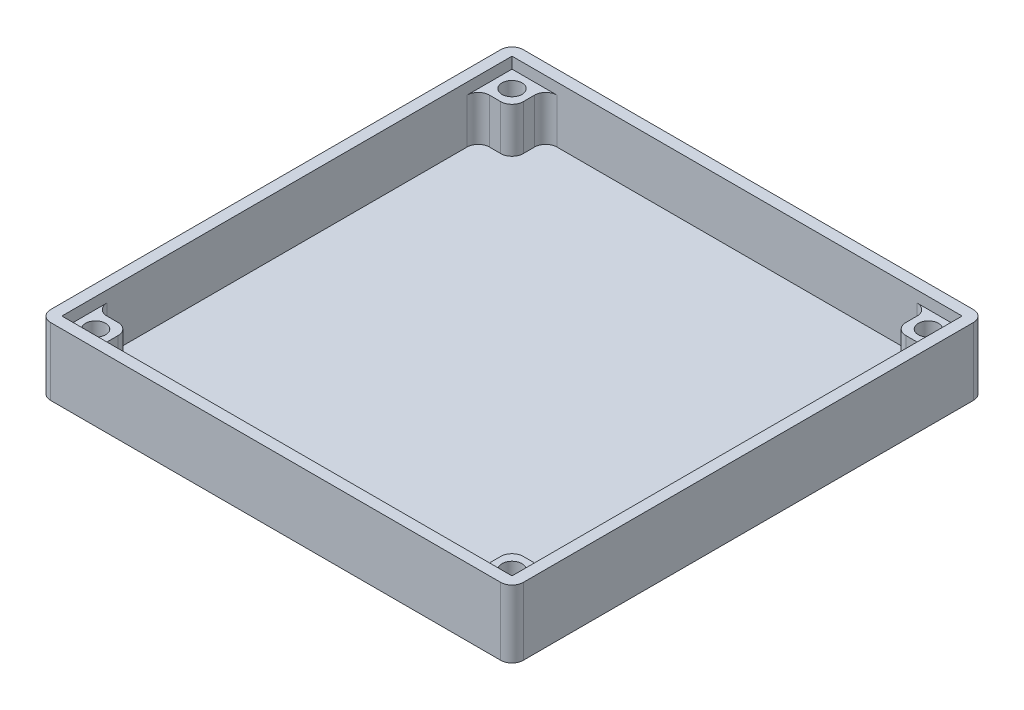
SolidWorks part; units mm, degrees
ref_plane "Front Plane" through (0, 0, 0) normal (0, 0, 1) x (1, 0, 0)
ref_plane "Top Plane" through (0, 0, 0) normal (0, 1, 0) x (1, 0, 0)
ref_plane "Right Plane" through (0, 0, 0) normal (1, 0, 0) x (0, 0, -1)
sketch "Sketch1" plane through (0, 0, 0) normal (0, 1, 0) x (1, 0, 0)
  line L0 (0, 0) -> (0, 50.8)
  line L1 (0, 50.8) -> (50.8, 50.8)
  line L2 (50.8, 50.8) -> (50.8, 0)
  line L3 (50.8, 0) -> (0, 0)
  line L4 (29.845, 40.64) -> (28.575, 40.64)
  line L5 (30.48, 43.18) -> (30.48, 38.1)
  line L6 (30.48, 38.1) -> (27.94, 38.1)
  line L7 (27.94, 38.1) -> (27.94, 43.18)
  line L8 (27.94, 43.18) -> (30.48, 43.18)
  line L9 (28.3382, 37.639) -> (28.245, 37.7322)
  line L10 (28.245, 37.7322) -> (28.0586, 37.7322)
  line L11 (28.0586, 37.7322) -> (27.9654, 37.639)
  line L12 (27.9654, 37.639) -> (27.9654, 37.2661)
  line L13 (27.9654, 37.2661) -> (28.0586, 37.1729)
  line L14 (28.0586, 37.1729) -> (28.245, 37.1729)
  line L15 (28.245, 37.1729) -> (28.3382, 37.2661)
  line L16 (28.5267, 37.5457) -> (28.7131, 37.7322)
  line L17 (28.7131, 37.7322) -> (28.7131, 37.1729)
  line L18 (28.5267, 37.1729) -> (28.8996, 37.1729)
  line L19 (28.2829, 43.8957) -> (28.4693, 44.0822)
  line L20 (28.4693, 44.0822) -> (28.4693, 43.5229)
  line L21 (28.2829, 43.5229) -> (28.6557, 43.5229)
  line L22 (28.8442, 43.6161) -> (28.8442, 43.989)
  line L23 (28.8442, 43.989) -> (28.9374, 44.0822)
  line L24 (28.9374, 44.0822) -> (29.1238, 44.0822)
  line L25 (29.1238, 44.0822) -> (29.2171, 43.989)
  line L26 (29.2171, 43.989) -> (29.2171, 43.6161)
  line L27 (29.2171, 43.6161) -> (29.1238, 43.5229)
  line L28 (29.1238, 43.5229) -> (28.9374, 43.5229)
  line L29 (28.9374, 43.5229) -> (28.8442, 43.6161)
  line L30 (28.8442, 43.6161) -> (29.2171, 43.989)
  line L31 (29.4055, 43.8957) -> (29.4055, 43.6161)
  line L32 (29.4055, 43.6161) -> (29.4987, 43.5229)
  line L33 (29.4987, 43.5229) -> (29.7784, 43.5229)
  line L34 (29.7784, 43.5229) -> (29.7784, 43.8957)
  line L35 (29.9668, 43.5229) -> (29.9668, 44.0822)
  line L36 (29.9668, 44.0822) -> (30.3397, 44.0822)
  line L37 (29.9668, 43.8025) -> (30.1533, 43.8025)
  line L38 (24.765, 40.64) -> (26.035, 40.64)
  line L39 (24.13, 38.1) -> (24.13, 43.18)
  line L40 (24.13, 43.18) -> (26.67, 43.18)
  line L41 (26.67, 43.18) -> (26.67, 38.1)
  line L42 (26.67, 38.1) -> (24.13, 38.1)
  line L43 (24.6756, 37.6644) -> (24.5824, 37.7576)
  line L44 (24.5824, 37.7576) -> (24.396, 37.7576)
  line L45 (24.396, 37.7576) -> (24.3028, 37.6644)
  line L46 (24.3028, 37.6644) -> (24.3028, 37.2915)
  line L47 (24.3028, 37.2915) -> (24.396, 37.1983)
  line L48 (24.396, 37.1983) -> (24.5824, 37.1983)
  line L49 (24.5824, 37.1983) -> (24.6756, 37.2915)
  line L50 (25.2369, 37.1983) -> (24.8641, 37.1983)
  line L51 (24.8641, 37.1983) -> (25.2369, 37.5711)
  line L52 (25.2369, 37.5711) -> (25.2369, 37.6644)
  line L53 (25.2369, 37.6644) -> (25.1437, 37.7576)
  line L54 (25.1437, 37.7576) -> (24.9573, 37.7576)
  line L55 (24.9573, 37.7576) -> (24.8641, 37.6644)
  line L56 (24.1326, 43.9211) -> (24.3191, 44.1076)
  line L57 (24.3191, 44.1076) -> (24.3191, 43.5483)
  line L58 (24.1326, 43.5483) -> (24.5055, 43.5483)
  line L59 (24.694, 43.6415) -> (24.694, 44.0144)
  line L60 (24.694, 44.0144) -> (24.7872, 44.1076)
  line L61 (24.7872, 44.1076) -> (24.9736, 44.1076)
  line L62 (24.9736, 44.1076) -> (25.0668, 44.0144)
  line L63 (25.0668, 44.0144) -> (25.0668, 43.6415)
  line L64 (25.0668, 43.6415) -> (24.9736, 43.5483)
  line L65 (24.9736, 43.5483) -> (24.7872, 43.5483)
  line L66 (24.7872, 43.5483) -> (24.694, 43.6415)
  line L67 (24.694, 43.6415) -> (25.0668, 44.0144)
  line L68 (25.2553, 43.9211) -> (25.2553, 43.6415)
  line L69 (25.2553, 43.6415) -> (25.3485, 43.5483)
  line L70 (25.3485, 43.5483) -> (25.6281, 43.5483)
  line L71 (25.6281, 43.5483) -> (25.6281, 43.9211)
  line L72 (25.8166, 43.5483) -> (25.8166, 44.1076)
  line L73 (25.8166, 44.1076) -> (26.1894, 44.1076)
  line L74 (25.8166, 43.8279) -> (26.003, 43.8279)
  line L75 (15.748, 34.29) -> (19.812, 34.29)
  line L76 (15.748, 34.29) -> (15.748, 31.75)
  line L77 (19.812, 31.75) -> (15.748, 31.75)
  line L78 (19.812, 31.75) -> (19.812, 34.29)
  line L79 (12.7, 33.02) -> (13.716, 33.02)
  line L80 (22.86, 33.02) -> (21.844, 33.02)
  line L81 (18.415, 33.02) -> (17.78, 33.02)
  line L82 (16.764, 32.385) -> (16.764, 33.655)
  line L83 (16.764, 33.655) -> (17.78, 33.02)
  line L84 (17.78, 33.02) -> (16.256, 33.02)
  line L85 (17.78, 33.02) -> (16.764, 32.385)
  line L86 (17.78, 32.385) -> (17.78, 33.02)
  line L87 (17.78, 33.02) -> (17.78, 33.655)
  line L88 (12.8591, 35.3702) -> (13.2404, 35.7515)
  line L89 (13.2404, 35.7515) -> (13.2404, 34.6075)
  line L90 (12.8591, 34.6075) -> (13.6217, 34.6075)
  line L91 (14.0285, 34.6075) -> (14.0285, 35.7515)
  line L92 (14.0285, 35.7515) -> (14.7912, 34.6075)
  line L93 (14.7912, 34.6075) -> (14.7912, 35.7515)
  line L94 (15.7699, 34.6075) -> (15.7699, 35.7515)
  line L95 (15.7699, 35.7515) -> (15.1979, 35.1795)
  line L96 (15.1979, 35.1795) -> (15.9605, 35.1795)
  line L97 (16.3673, 34.7982) -> (16.3673, 35.5608)
  line L98 (16.3673, 35.5608) -> (16.558, 35.7515)
  line L99 (16.558, 35.7515) -> (16.9393, 35.7515)
  line L100 (16.9393, 35.7515) -> (17.1299, 35.5608)
  line L101 (17.1299, 35.5608) -> (17.1299, 34.7982)
  line L102 (17.1299, 34.7982) -> (16.9393, 34.6075)
  line L103 (16.9393, 34.6075) -> (16.558, 34.6075)
  line L104 (16.558, 34.6075) -> (16.3673, 34.7982)
  line L105 (16.3673, 34.7982) -> (17.1299, 35.5608)
  line L106 (17.5367, 34.7982) -> (17.5367, 35.5608)
  line L107 (17.5367, 35.5608) -> (17.7273, 35.7515)
  line L108 (17.7273, 35.7515) -> (18.1087, 35.7515)
  line L109 (18.1087, 35.7515) -> (18.2993, 35.5608)
  line L110 (18.2993, 35.5608) -> (18.2993, 34.7982)
  line L111 (18.2993, 34.7982) -> (18.1087, 34.6075)
  line L112 (18.1087, 34.6075) -> (17.7273, 34.6075)
  line L113 (17.7273, 34.6075) -> (17.5367, 34.7982)
  line L114 (17.5367, 34.7982) -> (18.2993, 35.5608)
  line L115 (18.7061, 35.3702) -> (19.0874, 35.7515)
  line L116 (19.0874, 35.7515) -> (19.0874, 34.6075)
  line L117 (18.7061, 34.6075) -> (19.4687, 34.6075)
  line L118 (4.39, 39.64) -> (6.49, 39.64)
  line L119 (13.39, 50.34) -> (13.39, 53.24)
  line L120 (4.39, 53.24) -> (4.39, 50.34)
  line L121 (4.39, 53.24) -> (13.39, 53.24)
  line L122 (4.39, 50.34) -> (4.39, 45.04)
  line L123 (4.39, 39.64) -> (4.39, 40.34)
  line L124 (13.39, 50.34) -> (13.39, 39.64)
  line L125 (13.39, 39.64) -> (11.29, 39.64)
  line L126 (13.39, 50.34) -> (4.39, 50.34)
  line L127 (11.5901, 47.9299) -> (11.6536, 47.8663)
  line L128 (11.6536, 47.8663) -> (11.7172, 47.8663)
  line L129 (11.7172, 47.8663) -> (11.7807, 47.9299)
  line L130 (11.7807, 47.9299) -> (11.7807, 48.2476)
  line L131 (11.7172, 48.2476) -> (11.8443, 48.2476)
  line L132 (11.9643, 47.8663) -> (11.9643, 48.2476)
  line L133 (11.9643, 48.2476) -> (12.1549, 48.2476)
  line L134 (12.1549, 48.2476) -> (12.2185, 48.1841)
  line L135 (12.2185, 48.1841) -> (12.2185, 48.057)
  line L136 (12.2185, 48.057) -> (12.1549, 47.9934)
  line L137 (12.1549, 47.9934) -> (11.9643, 47.9934)
  line L138 (12.3385, 48.1205) -> (12.4656, 48.2476)
  line L139 (12.4656, 48.2476) -> (12.4656, 47.8663)
  line L140 (12.3385, 47.8663) -> (12.5927, 47.8663)
  line L141 (7.848, 49.1363) -> (7.848, 49.5176)
  line L142 (7.848, 49.5176) -> (8.0387, 49.5176)
  line L143 (8.0387, 49.5176) -> (8.1022, 49.4541)
  line L144 (8.1022, 49.4541) -> (8.1022, 49.327)
  line L145 (8.1022, 49.327) -> (8.0387, 49.2634)
  line L146 (8.0387, 49.2634) -> (7.848, 49.2634)
  line L147 (8.4129, 49.5176) -> (8.2858, 49.5176)
  line L148 (8.2858, 49.5176) -> (8.2222, 49.4541)
  line L149 (8.2222, 49.4541) -> (8.2222, 49.1999)
  line L150 (8.2222, 49.1999) -> (8.2858, 49.1363)
  line L151 (8.2858, 49.1363) -> (8.4129, 49.1363)
  line L152 (8.4129, 49.1363) -> (8.4764, 49.1999)
  line L153 (8.4764, 49.1999) -> (8.4764, 49.4541)
  line L154 (8.4764, 49.4541) -> (8.4129, 49.5176)
  line L155 (8.5964, 49.5176) -> (8.5964, 49.1363)
  line L156 (8.5964, 49.1363) -> (8.7235, 49.2634)
  line L157 (8.7235, 49.2634) -> (8.8506, 49.1363)
  line L158 (8.8506, 49.1363) -> (8.8506, 49.5176)
  line L159 (9.2248, 49.5176) -> (8.9706, 49.5176)
  line L160 (8.9706, 49.5176) -> (8.9706, 49.1363)
  line L161 (8.9706, 49.1363) -> (9.2248, 49.1363)
  line L162 (8.9706, 49.327) -> (9.0977, 49.327)
  line L163 (9.3448, 49.1363) -> (9.3448, 49.5176)
  line L164 (9.3448, 49.5176) -> (9.5355, 49.5176)
  line L165 (9.5355, 49.5176) -> (9.599, 49.4541)
  line L166 (9.599, 49.4541) -> (9.599, 49.327)
  line L167 (9.599, 49.327) -> (9.5355, 49.2634)
  line L168 (9.5355, 49.2634) -> (9.3448, 49.2634)
  line L169 (9.4719, 49.2634) -> (9.599, 49.1363)
  line L170 (9.719, 49.0727) -> (9.9733, 49.0727)
  line L171 (10.0932, 49.1999) -> (10.1568, 49.1363)
  line L172 (10.1568, 49.1363) -> (10.2204, 49.1363)
  line L173 (10.2204, 49.1363) -> (10.2839, 49.1999)
  line L174 (10.2839, 49.1999) -> (10.2839, 49.5176)
  line L175 (10.2204, 49.5176) -> (10.3475, 49.5176)
  line L176 (10.4674, 49.1363) -> (10.4674, 49.3905)
  line L177 (10.4674, 49.3905) -> (10.5945, 49.5176)
  line L178 (10.5945, 49.5176) -> (10.7217, 49.3905)
  line L179 (10.7217, 49.3905) -> (10.7217, 49.1363)
  line L180 (10.4674, 49.327) -> (10.7217, 49.327)
  line L181 (11.0959, 49.4541) -> (11.0323, 49.5176)
  line L182 (11.0323, 49.5176) -> (10.9052, 49.5176)
  line L183 (10.9052, 49.5176) -> (10.8417, 49.4541)
  line L184 (10.8417, 49.4541) -> (10.8417, 49.1999)
  line L185 (10.8417, 49.1999) -> (10.9052, 49.1363)
  line L186 (10.9052, 49.1363) -> (11.0323, 49.1363)
  line L187 (11.0323, 49.1363) -> (11.0959, 49.1999)
  line L188 (11.2159, 49.5176) -> (11.2159, 49.1363)
  line L189 (11.2159, 49.2634) -> (11.4701, 49.5176)
  line L190 (11.2794, 49.327) -> (11.4701, 49.1363)
  line L191 (11.5901, 49.1363) -> (11.5901, 49.5176)
  line L192 (11.5901, 49.5176) -> (11.7807, 49.5176)
  line L193 (11.7807, 49.5176) -> (11.8443, 49.4541)
  line L194 (11.8443, 49.4541) -> (11.8443, 49.327)
  line L195 (11.8443, 49.327) -> (11.7807, 49.2634)
  line L196 (11.7807, 49.2634) -> (11.5901, 49.2634)
  line L197 (12.0914, 49.1363) -> (12.0914, 49.5176)
  line L198 (11.9643, 49.5176) -> (12.2185, 49.5176)
  line L199 (12.3385, 49.1363) -> (12.3385, 49.5176)
  line L200 (12.3385, 49.327) -> (12.5927, 49.327)
  line L201 (12.5927, 49.5176) -> (12.5927, 49.1363)
  line L202 (10.795, 1.27) -> (24.765, 1.27)
  line L203 (24.765, 1.27) -> (24.765, 35.56)
  line L204 (24.765, 35.56) -> (10.795, 35.56)
  line L205 (10.795, 35.56) -> (10.795, 1.27)
  line L206 (14.1986, 3.8354) -> (13.6393, 3.8354)
  line L207 (13.6393, 3.8354) -> (13.6393, 4.115)
  line L208 (13.6393, 4.115) -> (13.7325, 4.2082)
  line L209 (13.7325, 4.2082) -> (13.919, 4.2082)
  line L210 (13.919, 4.2082) -> (14.0122, 4.115)
  line L211 (14.0122, 4.115) -> (14.0122, 3.8354)
  line L212 (14.0122, 4.0218) -> (14.1986, 4.2082)
  line L213 (13.6393, 4.3967) -> (14.1986, 4.7696)
  line L214 (13.6393, 4.7696) -> (14.1986, 4.3967)
  line L215 (16.7386, 4.0218) -> (16.1793, 4.0218)
  line L216 (16.1793, 3.8354) -> (16.1793, 4.2082)
  line L217 (16.1793, 4.3967) -> (16.7386, 4.7696)
  line L218 (16.1793, 4.7696) -> (16.7386, 4.3967)
  line L219 (18.8125, 4.2082) -> (18.7193, 4.115)
  line L220 (18.7193, 4.115) -> (18.7193, 3.9286)
  line L221 (18.7193, 3.9286) -> (18.8125, 3.8354)
  line L222 (18.8125, 3.8354) -> (19.1854, 3.8354)
  line L223 (19.1854, 3.8354) -> (19.2786, 3.9286)
  line L224 (19.2786, 3.9286) -> (19.2786, 4.115)
  line L225 (19.2786, 4.115) -> (19.1854, 4.2082)
  line L226 (19.1854, 4.2082) -> (18.999, 4.2082)
  line L227 (18.999, 4.2082) -> (18.999, 4.0218)
  line L228 (19.2786, 4.3967) -> (18.7193, 4.3967)
  line L229 (18.7193, 4.3967) -> (19.2786, 4.7696)
  line L230 (19.2786, 4.7696) -> (18.7193, 4.7696)
  line L231 (18.7193, 4.958) -> (19.2786, 4.958)
  line L232 (19.2786, 4.958) -> (19.2786, 5.2377)
  line L233 (19.2786, 5.2377) -> (19.1854, 5.3309)
  line L234 (19.1854, 5.3309) -> (18.8125, 5.3309)
  line L235 (18.8125, 5.3309) -> (18.7193, 5.2377)
  line L236 (18.7193, 5.2377) -> (18.7193, 4.958)
  line L237 (21.2593, 3.8354) -> (21.6322, 3.8354)
  line L238 (21.6322, 3.8354) -> (21.8186, 4.0218)
  line L239 (21.8186, 4.0218) -> (21.6322, 4.2082)
  line L240 (21.6322, 4.2082) -> (21.2593, 4.2082)
  line L241 (21.3525, 4.7696) -> (21.2593, 4.6763)
  line L242 (21.2593, 4.6763) -> (21.2593, 4.4899)
  line L243 (21.2593, 4.4899) -> (21.3525, 4.3967)
  line L244 (21.3525, 4.3967) -> (21.7254, 4.3967)
  line L245 (21.7254, 4.3967) -> (21.8186, 4.4899)
  line L246 (21.8186, 4.4899) -> (21.8186, 4.6763)
  line L247 (21.8186, 4.6763) -> (21.7254, 4.7696)
  line L248 (21.3525, 5.3309) -> (21.2593, 5.2377)
  line L249 (21.2593, 5.2377) -> (21.2593, 5.0512)
  line L250 (21.2593, 5.0512) -> (21.3525, 4.958)
  line L251 (21.3525, 4.958) -> (21.7254, 4.958)
  line L252 (21.7254, 4.958) -> (21.8186, 5.0512)
  line L253 (21.8186, 5.0512) -> (21.8186, 5.2377)
  line L254 (21.8186, 5.2377) -> (21.7254, 5.3309)
  line L255 (10.0752, 1.3335) -> (10.2235, 1.4818)
  line L256 (10.2235, 1.4818) -> (10.2235, 1.6301)
  line L257 (10.2235, 1.6301) -> (10.0752, 1.7784)
  line L258 (10.0752, 1.7784) -> (9.3337, 1.7784)
  line L259 (9.3337, 1.6301) -> (9.3337, 1.9267)
  line L260 (10.3718, 2.269) -> (10.3718, 2.8622)
  line L261 (10.2235, 3.2045) -> (9.3337, 3.2045)
  line L262 (9.3337, 3.2045) -> (9.3337, 3.6494)
  line L263 (9.3337, 3.6494) -> (9.482, 3.7977)
  line L264 (9.482, 3.7977) -> (9.6303, 3.7977)
  line L265 (9.6303, 3.7977) -> (9.7786, 3.6494)
  line L266 (9.7786, 3.6494) -> (9.9269, 3.7977)
  line L267 (9.9269, 3.7977) -> (10.0752, 3.7977)
  line L268 (10.0752, 3.7977) -> (10.2235, 3.6494)
  line L269 (10.2235, 3.6494) -> (10.2235, 3.2045)
  line L270 (9.7786, 3.2045) -> (9.7786, 3.6494)
  line L271 (10.2235, 4.4366) -> (9.3337, 4.4366)
  line L272 (9.3337, 4.14) -> (9.3337, 4.7332)
  line L273 (10.3718, 5.0756) -> (10.3718, 5.6687)
  line L274 (10.2235, 6.0111) -> (9.3337, 6.0111)
  line L275 (9.3337, 6.0111) -> (9.3337, 6.456)
  line L276 (9.3337, 6.456) -> (9.482, 6.6043)
  line L277 (9.482, 6.6043) -> (9.6303, 6.6043)
  line L278 (9.6303, 6.6043) -> (9.7786, 6.456)
  line L279 (9.7786, 6.456) -> (9.9269, 6.6043)
  line L280 (9.9269, 6.6043) -> (10.0752, 6.6043)
  line L281 (10.0752, 6.6043) -> (10.2235, 6.456)
  line L282 (10.2235, 6.456) -> (10.2235, 6.0111)
  line L283 (9.7786, 6.0111) -> (9.7786, 6.456)
  line L284 (9.3337, 7.3915) -> (9.3337, 7.0949)
  line L285 (9.3337, 7.0949) -> (9.482, 6.9466)
  line L286 (9.482, 6.9466) -> (10.0752, 6.9466)
  line L287 (10.0752, 6.9466) -> (10.2235, 7.0949)
  line L288 (10.2235, 7.0949) -> (10.2235, 7.3915)
  line L289 (10.2235, 7.3915) -> (10.0752, 7.5398)
  line L290 (10.0752, 7.5398) -> (9.482, 7.5398)
  line L291 (9.482, 7.5398) -> (9.3337, 7.3915)
  line L292 (10.2235, 7.8821) -> (9.6303, 7.8821)
  line L293 (9.6303, 7.8821) -> (9.3337, 8.1787)
  line L294 (9.3337, 8.1787) -> (9.6303, 8.4753)
  line L295 (9.6303, 8.4753) -> (10.2235, 8.4753)
  line L296 (9.7786, 7.8821) -> (9.7786, 8.4753)
  line L297 (10.2235, 8.8177) -> (9.3337, 8.8177)
  line L298 (9.3337, 8.8177) -> (9.3337, 9.2625)
  line L299 (9.3337, 9.2625) -> (9.482, 9.4108)
  line L300 (9.482, 9.4108) -> (9.7786, 9.4108)
  line L301 (9.7786, 9.4108) -> (9.9269, 9.2625)
  line L302 (9.9269, 9.2625) -> (9.9269, 8.8177)
  line L303 (9.9269, 9.1142) -> (10.2235, 9.4108)
  line L304 (9.3337, 9.7532) -> (10.2235, 9.7532)
  line L305 (10.2235, 9.7532) -> (10.2235, 10.198)
  line L306 (10.2235, 10.198) -> (10.0752, 10.3463)
  line L307 (10.0752, 10.3463) -> (9.482, 10.3463)
  line L308 (9.482, 10.3463) -> (9.3337, 10.198)
  line L309 (9.3337, 10.198) -> (9.3337, 9.7532)
  line L310 (10.3718, 10.6887) -> (10.3718, 11.2819)
  line L311 (9.6303, 11.6242) -> (9.3337, 11.9208)
  line L312 (9.3337, 11.9208) -> (10.2235, 11.9208)
  line L313 (10.2235, 11.6242) -> (10.2235, 12.2174)
  line L314 (3.81, 35.8648) -> (1.27, 35.8648)
  line L315 (0.9515, 36.2585) -> (2.0955, 36.2585)
  line L316 (2.0955, 36.2585) -> (2.0955, 37.0212)
  line L317 (0.9515, 38.1906) -> (0.9515, 37.4279)
  line L318 (0.9515, 37.4279) -> (2.0955, 37.4279)
  line L319 (2.0955, 37.4279) -> (2.0955, 38.1906)
  line L320 (1.5235, 37.4279) -> (1.5235, 37.8092)
  line L321 (0.9515, 38.5973) -> (2.0955, 38.5973)
  line L322 (2.0955, 38.5973) -> (2.0955, 39.1693)
  line L323 (2.0955, 39.1693) -> (1.9048, 39.3599)
  line L324 (1.9048, 39.3599) -> (1.1422, 39.3599)
  line L325 (1.1422, 39.3599) -> (0.9515, 39.1693)
  line L326 (0.9515, 39.1693) -> (0.9515, 38.5973)
  line L327 (1.3328, 39.7667) -> (0.9515, 40.148)
  line L328 (0.9515, 40.148) -> (2.0955, 40.148)
  line L329 (2.0955, 39.7667) -> (2.0955, 40.5293)
  line L330 (2.6768, 32.6898) -> (2.4032, 32.6898)
  line L331 (2.4032, 32.6898) -> (2.2098, 32.8832)
  line L332 (2.2098, 32.8832) -> (2.2098, 33.1568)
  line L333 (2.2098, 33.1568) -> (2.4032, 33.3502)
  line L334 (2.4032, 33.3502) -> (2.6768, 33.3502)
  line L335 (2.6768, 33.3502) -> (2.8702, 33.1568)
  line L336 (2.8702, 33.1568) -> (2.8702, 32.8832)
  line L337 (2.8702, 32.8832) -> (2.6768, 32.6898)
  line L338 (2.6768, 32.6898) -> (2.4032, 32.6898)
  line L339 (2.6768, 32.6898) -> (2.4032, 32.6898)
  line L340 (2.4032, 32.6898) -> (2.2098, 32.8832)
  line L341 (2.2098, 32.8832) -> (2.2098, 33.1568)
  line L342 (2.2098, 33.1568) -> (2.4032, 33.3502)
  line L343 (2.4032, 33.3502) -> (2.6768, 33.3502)
  line L344 (2.6768, 33.3502) -> (2.8702, 33.1568)
  line L345 (2.8702, 33.1568) -> (2.8702, 32.8832)
  line L346 (2.8702, 32.8832) -> (2.6768, 32.6898)
  line L347 (2.6768, 32.6898) -> (2.4032, 32.6898)
  line L348 (2.6768, 35.2298) -> (2.4032, 35.2298)
  line L349 (2.4032, 35.2298) -> (2.2098, 35.4232)
  line L350 (2.2098, 35.4232) -> (2.2098, 35.6968)
  line L351 (2.2098, 35.6968) -> (2.4032, 35.8902)
  line L352 (2.4032, 35.8902) -> (2.6768, 35.8902)
  line L353 (2.6768, 35.8902) -> (2.8702, 35.6968)
  line L354 (2.8702, 35.6968) -> (2.8702, 35.4232)
  line L355 (2.8702, 35.4232) -> (2.6768, 35.2298)
  line L356 (2.6768, 35.2298) -> (2.4032, 35.2298)
  line L357 (2.6768, 35.2298) -> (2.4032, 35.2298)
  line L358 (2.4032, 35.2298) -> (2.2098, 35.4232)
  line L359 (2.2098, 35.4232) -> (2.2098, 35.6968)
  line L360 (2.2098, 35.6968) -> (2.4032, 35.8902)
  line L361 (2.4032, 35.8902) -> (2.6768, 35.8902)
  line L362 (2.6768, 35.8902) -> (2.8702, 35.6968)
  line L363 (2.8702, 35.6968) -> (2.8702, 35.4232)
  line L364 (2.8702, 35.4232) -> (2.6768, 35.2298)
  line L365 (2.6768, 35.2298) -> (2.4032, 35.2298)
  line L366 (10.16, 36.83) -> (10.16, 31.75)
  line L367 (10.16, 31.75) -> (5.08, 31.75)
  line L368 (5.08, 31.75) -> (5.08, 36.83)
  line L369 (5.08, 36.83) -> (10.16, 36.83)
  line L370 (8.9275, 32.8596) -> (8.9275, 32.6139)
  line L371 (8.9275, 32.6139) -> (9.0504, 32.491)
  line L372 (9.0504, 32.491) -> (9.5418, 32.491)
  line L373 (9.5418, 32.491) -> (9.6647, 32.6139)
  line L374 (9.6647, 32.6139) -> (9.6647, 32.8596)
  line L375 (9.6647, 32.8596) -> (9.5418, 32.9825)
  line L376 (9.5418, 32.9825) -> (9.0504, 32.9825)
  line L377 (9.0504, 32.9825) -> (8.9275, 32.8596)
  line L378 (9.6647, 33.2394) -> (8.9275, 33.2394)
  line L379 (8.9275, 33.2394) -> (9.6647, 33.7309)
  line L380 (9.6647, 33.7309) -> (8.9275, 33.7309)
  line L381 (8.9275, 34.3565) -> (8.9275, 34.1107)
  line L382 (8.9275, 34.1107) -> (9.0504, 33.9878)
  line L383 (9.0504, 33.9878) -> (9.5418, 33.9878)
  line L384 (9.5418, 33.9878) -> (9.6647, 34.1107)
  line L385 (9.6647, 34.1107) -> (9.6647, 34.3565)
  line L386 (9.6647, 34.3565) -> (9.5418, 34.4793)
  line L387 (9.5418, 34.4793) -> (9.0504, 34.4793)
  line L388 (9.0504, 34.4793) -> (8.9275, 34.3565)
  line L389 (9.6647, 34.7363) -> (8.9275, 34.7363)
  line L390 (8.9275, 34.7363) -> (8.9275, 35.2277)
  line L391 (9.2961, 34.7363) -> (9.2961, 34.982)
  line L392 (9.6647, 35.4847) -> (8.9275, 35.4847)
  line L393 (8.9275, 35.4847) -> (8.9275, 35.9762)
  line L394 (9.2961, 35.4847) -> (9.2961, 35.7304)
  line L395 (5.7525, 31.7426) -> (6.4897, 31.7426)
  line L396 (6.4897, 31.7426) -> (6.4897, 32.1112)
  line L397 (6.4897, 32.1112) -> (6.3668, 32.2341)
  line L398 (6.3668, 32.2341) -> (5.8754, 32.2341)
  line L399 (5.8754, 32.2341) -> (5.7525, 32.1112)
  line L400 (5.7525, 32.1112) -> (5.7525, 31.7426)
  line L401 (5.8754, 32.9825) -> (5.7525, 32.8596)
  line L402 (5.7525, 32.8596) -> (5.7525, 32.6139)
  line L403 (5.7525, 32.6139) -> (5.8754, 32.491)
  line L404 (5.8754, 32.491) -> (5.9982, 32.491)
  line L405 (5.9982, 32.491) -> (6.1211, 32.6139)
  line L406 (6.1211, 32.6139) -> (6.1211, 32.8596)
  line L407 (6.1211, 32.8596) -> (6.244, 32.9825)
  line L408 (6.244, 32.9825) -> (6.3668, 32.9825)
  line L409 (6.3668, 32.9825) -> (6.4897, 32.8596)
  line L410 (6.4897, 32.8596) -> (6.4897, 32.6139)
  line L411 (6.4897, 32.6139) -> (6.3668, 32.491)
  line L412 (6.1211, 33.2394) -> (6.1211, 33.7309)
  line L413 (6.4897, 34.4793) -> (6.4897, 33.9878)
  line L414 (6.4897, 33.9878) -> (5.9982, 34.4793)
  line L415 (5.9982, 34.4793) -> (5.8754, 34.4793)
  line L416 (5.8754, 34.4793) -> (5.7525, 34.3565)
  line L417 (5.7525, 34.3565) -> (5.7525, 34.1107)
  line L418 (5.7525, 34.1107) -> (5.8754, 33.9878)
  line L419 (6.4897, 35.2277) -> (6.4897, 34.7363)
  line L420 (6.4897, 34.7363) -> (5.9982, 35.2277)
  line L421 (5.9982, 35.2277) -> (5.8754, 35.2277)
  line L422 (5.8754, 35.2277) -> (5.7525, 35.1049)
  line L423 (5.7525, 35.1049) -> (5.7525, 34.8591)
  line L424 (5.7525, 34.8591) -> (5.8754, 34.7363)
  line L425 (5.8754, 35.4847) -> (5.7525, 35.6075)
  line L426 (5.7525, 35.6075) -> (5.7525, 35.8533)
  line L427 (5.7525, 35.8533) -> (5.8754, 35.9762)
  line L428 (5.8754, 35.9762) -> (5.9982, 35.9762)
  line L429 (5.9982, 35.9762) -> (6.1211, 35.8533)
  line L430 (6.1211, 35.8533) -> (6.244, 35.9762)
  line L431 (6.244, 35.9762) -> (6.3668, 35.9762)
  line L432 (6.3668, 35.9762) -> (6.4897, 35.8533)
  line L433 (6.4897, 35.8533) -> (6.4897, 35.6075)
  line L434 (6.4897, 35.6075) -> (6.3668, 35.4847)
  line L435 (6.3668, 35.4847) -> (6.244, 35.4847)
  line L436 (6.244, 35.4847) -> (6.1211, 35.6075)
  line L437 (6.1211, 35.6075) -> (5.9982, 35.4847)
  line L438 (5.9982, 35.4847) -> (5.8754, 35.4847)
  line L439 (6.1211, 35.6075) -> (6.1211, 35.8533)
  line L440 (15.24, 21.082) -> (20.32, 21.082)
  line L441 (20.32, 21.082) -> (20.32, 20.32)
  line L442 (20.32, 20.32) -> (20.32, 19.558)
  line L443 (20.32, 19.558) -> (15.24, 19.558)
  line L444 (15.24, 19.558) -> (15.24, 20.32)
  line L445 (15.24, 20.32) -> (15.24, 21.082)
  line L446 (20.32, 20.32) -> (20.574, 20.32)
  line L447 (15.24, 20.32) -> (14.986, 20.32)
  line L448 (15.2527, 21.6027) -> (15.2527, 21.984)
  line L449 (15.2527, 21.984) -> (15.4434, 21.984)
  line L450 (15.4434, 21.984) -> (15.5069, 21.9205)
  line L451 (15.5069, 21.9205) -> (15.5069, 21.7934)
  line L452 (15.5069, 21.7934) -> (15.4434, 21.7298)
  line L453 (15.4434, 21.7298) -> (15.2527, 21.7298)
  line L454 (15.3798, 21.7298) -> (15.5069, 21.6027)
  line L455 (15.6269, 21.8569) -> (15.754, 21.984)
  line L456 (15.754, 21.984) -> (15.754, 21.6027)
  line L457 (15.6269, 21.6027) -> (15.8811, 21.6027)
  line L458 (15.8242, 20.5914) -> (16.1123, 20.8795)
  line L459 (16.1123, 20.8795) -> (16.1123, 20.0152)
  line L460 (15.8242, 20.0152) -> (16.4004, 20.0152)
  line L461 (16.7597, 20.1593) -> (16.7597, 20.7355)
  line L462 (16.7597, 20.7355) -> (16.9038, 20.8795)
  line L463 (16.9038, 20.8795) -> (17.1919, 20.8795)
  line L464 (17.1919, 20.8795) -> (17.3359, 20.7355)
  line L465 (17.3359, 20.7355) -> (17.3359, 20.1593)
  line L466 (17.3359, 20.1593) -> (17.1919, 20.0152)
  line L467 (17.1919, 20.0152) -> (16.9038, 20.0152)
  line L468 (16.9038, 20.0152) -> (16.7597, 20.1593)
  line L469 (16.7597, 20.1593) -> (17.3359, 20.7355)
  line L470 (17.6952, 20.8795) -> (17.6952, 20.0152)
  line L471 (17.6952, 20.3033) -> (18.2715, 20.8795)
  line L472 (17.8393, 20.4474) -> (18.2715, 20.0152)
  line L473 (15.24, 18.542) -> (20.32, 18.542)
  line L474 (20.32, 18.542) -> (20.32, 17.78)
  line L475 (20.32, 17.78) -> (20.32, 17.018)
  line L476 (20.32, 17.018) -> (15.24, 17.018)
  line L477 (15.24, 17.018) -> (15.24, 17.78)
  line L478 (15.24, 17.78) -> (15.24, 18.542)
  line L479 (20.32, 17.78) -> (20.574, 17.78)
  line L480 (15.24, 17.78) -> (14.986, 17.78)
  line L481 (15.2527, 19.0627) -> (15.2527, 19.444)
  line L482 (15.2527, 19.444) -> (15.4434, 19.444)
  line L483 (15.4434, 19.444) -> (15.5069, 19.3805)
  line L484 (15.5069, 19.3805) -> (15.5069, 19.2534)
  line L485 (15.5069, 19.2534) -> (15.4434, 19.1898)
  line L486 (15.4434, 19.1898) -> (15.2527, 19.1898)
  line L487 (15.3798, 19.1898) -> (15.5069, 19.0627)
  line L488 (15.8811, 19.0627) -> (15.6269, 19.0627)
  line L489 (15.6269, 19.0627) -> (15.8811, 19.3169)
  line L490 (15.8811, 19.3169) -> (15.8811, 19.3805)
  line L491 (15.8811, 19.3805) -> (15.8176, 19.444)
  line L492 (15.8176, 19.444) -> (15.6905, 19.444)
  line L493 (15.6905, 19.444) -> (15.6269, 19.3805)
  line L494 (15.8242, 18.0514) -> (16.1123, 18.3395)
  line L495 (16.1123, 18.3395) -> (16.1123, 17.4752)
  line L496 (15.8242, 17.4752) -> (16.4004, 17.4752)
  line L497 (16.7597, 17.6193) -> (16.7597, 18.1955)
  line L498 (16.7597, 18.1955) -> (16.9038, 18.3395)
  line L499 (16.9038, 18.3395) -> (17.1919, 18.3395)
  line L500 (17.1919, 18.3395) -> (17.3359, 18.1955)
  line L501 (17.3359, 18.1955) -> (17.3359, 17.6193)
  line L502 (17.3359, 17.6193) -> (17.1919, 17.4752)
  line L503 (17.1919, 17.4752) -> (16.9038, 17.4752)
  line L504 (16.9038, 17.4752) -> (16.7597, 17.6193)
  line L505 (16.7597, 17.6193) -> (17.3359, 18.1955)
  line L506 (17.6952, 18.3395) -> (17.6952, 17.4752)
  line L507 (17.6952, 17.7633) -> (18.2715, 18.3395)
  line L508 (17.8393, 17.9074) -> (18.2715, 17.4752)
  line L509 (15.24, 16.002) -> (20.32, 16.002)
  line L510 (20.32, 16.002) -> (20.32, 15.24)
  line L511 (20.32, 15.24) -> (20.32, 14.478)
  line L512 (20.32, 14.478) -> (15.24, 14.478)
  line L513 (15.24, 14.478) -> (15.24, 15.24)
  line L514 (15.24, 15.24) -> (15.24, 16.002)
  line L515 (20.32, 15.24) -> (20.574, 15.24)
  line L516 (15.24, 15.24) -> (14.986, 15.24)
  line L517 (15.2527, 16.5227) -> (15.2527, 16.904)
  line L518 (15.2527, 16.904) -> (15.4434, 16.904)
  line L519 (15.4434, 16.904) -> (15.5069, 16.8405)
  line L520 (15.5069, 16.8405) -> (15.5069, 16.7134)
  line L521 (15.5069, 16.7134) -> (15.4434, 16.6498)
  line L522 (15.4434, 16.6498) -> (15.2527, 16.6498)
  line L523 (15.3798, 16.6498) -> (15.5069, 16.5227)
  line L524 (15.6269, 16.8405) -> (15.6905, 16.904)
  line L525 (15.6905, 16.904) -> (15.8176, 16.904)
  line L526 (15.8176, 16.904) -> (15.8811, 16.8405)
  line L527 (15.8811, 16.8405) -> (15.8811, 16.7769)
  line L528 (15.8811, 16.7769) -> (15.8176, 16.7134)
  line L529 (15.8176, 16.7134) -> (15.754, 16.7134)
  line L530 (15.8176, 16.7134) -> (15.8811, 16.6498)
  line L531 (15.8811, 16.6498) -> (15.8811, 16.5863)
  line L532 (15.8811, 16.5863) -> (15.8176, 16.5227)
  line L533 (15.8176, 16.5227) -> (15.6905, 16.5227)
  line L534 (15.6905, 16.5227) -> (15.6269, 16.5863)
  line L535 (15.8242, 15.5114) -> (16.1123, 15.7995)
  line L536 (16.1123, 15.7995) -> (16.1123, 14.9352)
  line L537 (15.8242, 14.9352) -> (16.4004, 14.9352)
  line L538 (16.7597, 15.0793) -> (16.7597, 15.6555)
  line L539 (16.7597, 15.6555) -> (16.9038, 15.7995)
  line L540 (16.9038, 15.7995) -> (17.1919, 15.7995)
  line L541 (17.1919, 15.7995) -> (17.3359, 15.6555)
  line L542 (17.3359, 15.6555) -> (17.3359, 15.0793)
  line L543 (17.3359, 15.0793) -> (17.1919, 14.9352)
  line L544 (17.1919, 14.9352) -> (16.9038, 14.9352)
  line L545 (16.9038, 14.9352) -> (16.7597, 15.0793)
  line L546 (16.7597, 15.0793) -> (17.3359, 15.6555)
  line L547 (17.6952, 15.7995) -> (17.6952, 14.9352)
  line L548 (17.6952, 15.2233) -> (18.2715, 15.7995)
  line L549 (17.8393, 15.3674) -> (18.2715, 14.9352)
  line L550 (15.24, 13.462) -> (20.32, 13.462)
  line L551 (20.32, 13.462) -> (20.32, 12.7)
  line L552 (20.32, 12.7) -> (20.32, 11.938)
  line L553 (20.32, 11.938) -> (15.24, 11.938)
  line L554 (15.24, 11.938) -> (15.24, 12.7)
  line L555 (15.24, 12.7) -> (15.24, 13.462)
  line L556 (20.32, 12.7) -> (20.574, 12.7)
  line L557 (15.24, 12.7) -> (14.986, 12.7)
  line L558 (15.2527, 13.9827) -> (15.2527, 14.364)
  line L559 (15.2527, 14.364) -> (15.4434, 14.364)
  line L560 (15.4434, 14.364) -> (15.5069, 14.3005)
  line L561 (15.5069, 14.3005) -> (15.5069, 14.1734)
  line L562 (15.5069, 14.1734) -> (15.4434, 14.1098)
  line L563 (15.4434, 14.1098) -> (15.2527, 14.1098)
  line L564 (15.3798, 14.1098) -> (15.5069, 13.9827)
  line L565 (15.8176, 13.9827) -> (15.8176, 14.364)
  line L566 (15.8176, 14.364) -> (15.6269, 14.1734)
  line L567 (15.6269, 14.1734) -> (15.8811, 14.1734)
  line L568 (15.8242, 12.9714) -> (16.1123, 13.2595)
  line L569 (16.1123, 13.2595) -> (16.1123, 12.3952)
  line L570 (15.8242, 12.3952) -> (16.4004, 12.3952)
  line L571 (16.7597, 12.5393) -> (16.7597, 13.1155)
  line L572 (16.7597, 13.1155) -> (16.9038, 13.2595)
  line L573 (16.9038, 13.2595) -> (17.1919, 13.2595)
  line L574 (17.1919, 13.2595) -> (17.3359, 13.1155)
  line L575 (17.3359, 13.1155) -> (17.3359, 12.5393)
  line L576 (17.3359, 12.5393) -> (17.1919, 12.3952)
  line L577 (17.1919, 12.3952) -> (16.9038, 12.3952)
  line L578 (16.9038, 12.3952) -> (16.7597, 12.5393)
  line L579 (16.7597, 12.5393) -> (17.3359, 13.1155)
  line L580 (17.6952, 13.2595) -> (17.6952, 12.3952)
  line L581 (17.6952, 12.6833) -> (18.2715, 13.2595)
  line L582 (17.8393, 12.8274) -> (18.2715, 12.3952)
  line L583 (15.24, 10.922) -> (20.32, 10.922)
  line L584 (20.32, 10.922) -> (20.32, 10.16)
  line L585 (20.32, 10.16) -> (20.32, 9.398)
  line L586 (20.32, 9.398) -> (15.24, 9.398)
  line L587 (15.24, 9.398) -> (15.24, 10.16)
  line L588 (15.24, 10.16) -> (15.24, 10.922)
  line L589 (20.32, 10.16) -> (20.574, 10.16)
  line L590 (15.24, 10.16) -> (14.986, 10.16)
  line L591 (15.2527, 11.4427) -> (15.2527, 11.824)
  line L592 (15.2527, 11.824) -> (15.4434, 11.824)
  line L593 (15.4434, 11.824) -> (15.5069, 11.7605)
  line L594 (15.5069, 11.7605) -> (15.5069, 11.6334)
  line L595 (15.5069, 11.6334) -> (15.4434, 11.5698)
  line L596 (15.4434, 11.5698) -> (15.2527, 11.5698)
  line L597 (15.3798, 11.5698) -> (15.5069, 11.4427)
  line L598 (15.8811, 11.824) -> (15.6269, 11.824)
  line L599 (15.6269, 11.824) -> (15.6269, 11.6334)
  line L600 (15.6269, 11.6334) -> (15.754, 11.6969)
  line L601 (15.754, 11.6969) -> (15.8176, 11.6969)
  line L602 (15.8176, 11.6969) -> (15.8811, 11.6334)
  line L603 (15.8811, 11.6334) -> (15.8811, 11.5063)
  line L604 (15.8811, 11.5063) -> (15.8176, 11.4427)
  line L605 (15.8176, 11.4427) -> (15.6905, 11.4427)
  line L606 (15.6905, 11.4427) -> (15.6269, 11.5063)
  line L607 (15.8242, 10.4314) -> (16.1123, 10.7195)
  line L608 (16.1123, 10.7195) -> (16.1123, 9.8552)
  line L609 (15.8242, 9.8552) -> (16.4004, 9.8552)
  line L610 (16.7597, 9.9993) -> (16.7597, 10.5755)
  line L611 (16.7597, 10.5755) -> (16.9038, 10.7195)
  line L612 (16.9038, 10.7195) -> (17.1919, 10.7195)
  line L613 (17.1919, 10.7195) -> (17.3359, 10.5755)
  line L614 (17.3359, 10.5755) -> (17.3359, 9.9993)
  line L615 (17.3359, 9.9993) -> (17.1919, 9.8552)
  line L616 (17.1919, 9.8552) -> (16.9038, 9.8552)
  line L617 (16.9038, 9.8552) -> (16.7597, 9.9993)
  line L618 (16.7597, 9.9993) -> (17.3359, 10.5755)
  line L619 (17.6952, 10.7195) -> (17.6952, 9.8552)
  line L620 (17.6952, 10.1433) -> (18.2715, 10.7195)
  line L621 (17.8393, 10.2874) -> (18.2715, 9.8552)
  line L622 (15.24, 8.382) -> (20.32, 8.382)
  line L623 (20.32, 8.382) -> (20.32, 7.62)
  line L624 (20.32, 7.62) -> (20.32, 6.858)
  line L625 (20.32, 6.858) -> (15.24, 6.858)
  line L626 (15.24, 6.858) -> (15.24, 7.62)
  line L627 (15.24, 7.62) -> (15.24, 8.382)
  line L628 (20.32, 7.62) -> (20.574, 7.62)
  line L629 (15.24, 7.62) -> (14.986, 7.62)
  line L630 (15.2527, 8.9027) -> (15.2527, 9.284)
  line L631 (15.2527, 9.284) -> (15.4434, 9.284)
  line L632 (15.4434, 9.284) -> (15.5069, 9.2205)
  line L633 (15.5069, 9.2205) -> (15.5069, 9.0934)
  line L634 (15.5069, 9.0934) -> (15.4434, 9.0298)
  line L635 (15.4434, 9.0298) -> (15.2527, 9.0298)
  line L636 (15.3798, 9.0298) -> (15.5069, 8.9027)
  line L637 (15.8811, 9.284) -> (15.754, 9.2205)
  line L638 (15.754, 9.2205) -> (15.6269, 9.0934)
  line L639 (15.6269, 9.0934) -> (15.6269, 8.9663)
  line L640 (15.6269, 8.9663) -> (15.6905, 8.9027)
  line L641 (15.6905, 8.9027) -> (15.8176, 8.9027)
  line L642 (15.8176, 8.9027) -> (15.8811, 8.9663)
  line L643 (15.8811, 8.9663) -> (15.8811, 9.0298)
  line L644 (15.8811, 9.0298) -> (15.8176, 9.0934)
  line L645 (15.8176, 9.0934) -> (15.6269, 9.0934)
  line L646 (15.8242, 7.8914) -> (16.1123, 8.1795)
  line L647 (16.1123, 8.1795) -> (16.1123, 7.3152)
  line L648 (15.8242, 7.3152) -> (16.4004, 7.3152)
  line L649 (16.7597, 7.4593) -> (16.7597, 8.0355)
  line L650 (16.7597, 8.0355) -> (16.9038, 8.1795)
  line L651 (16.9038, 8.1795) -> (17.1919, 8.1795)
  line L652 (17.1919, 8.1795) -> (17.3359, 8.0355)
  line L653 (17.3359, 8.0355) -> (17.3359, 7.4593)
  line L654 (17.3359, 7.4593) -> (17.1919, 7.3152)
  line L655 (17.1919, 7.3152) -> (16.9038, 7.3152)
  line L656 (16.9038, 7.3152) -> (16.7597, 7.4593)
  line L657 (16.7597, 7.4593) -> (17.3359, 8.0355)
  line L658 (17.6952, 8.1795) -> (17.6952, 7.3152)
  line L659 (17.6952, 7.6033) -> (18.2715, 8.1795)
  line L660 (17.8393, 7.7474) -> (18.2715, 7.3152)
  line L661 (15.24, 28.702) -> (20.32, 28.702)
  line L662 (20.32, 28.702) -> (20.32, 27.94)
  line L663 (20.32, 27.94) -> (20.32, 27.178)
  line L664 (20.32, 27.178) -> (15.24, 27.178)
  line L665 (15.24, 27.178) -> (15.24, 27.94)
  line L666 (15.24, 27.94) -> (15.24, 28.702)
  line L667 (20.32, 27.94) -> (20.574, 27.94)
  line L668 (15.24, 27.94) -> (14.986, 27.94)
  line L669 (15.2527, 29.2227) -> (15.2527, 29.604)
  line L670 (15.2527, 29.604) -> (15.4434, 29.604)
  line L671 (15.4434, 29.604) -> (15.5069, 29.5405)
  line L672 (15.5069, 29.5405) -> (15.5069, 29.4134)
  line L673 (15.5069, 29.4134) -> (15.4434, 29.3498)
  line L674 (15.4434, 29.3498) -> (15.2527, 29.3498)
  line L675 (15.3798, 29.3498) -> (15.5069, 29.2227)
  line L676 (15.6269, 29.604) -> (15.8811, 29.604)
  line L677 (15.8811, 29.604) -> (15.8811, 29.5405)
  line L678 (15.8811, 29.5405) -> (15.6269, 29.2863)
  line L679 (15.6269, 29.2863) -> (15.6269, 29.2227)
  line L680 (15.8242, 28.2114) -> (16.1123, 28.4995)
  line L681 (16.1123, 28.4995) -> (16.1123, 27.6352)
  line L682 (15.8242, 27.6352) -> (16.4004, 27.6352)
  line L683 (16.7597, 27.6352) -> (16.7597, 27.7793)
  line L684 (16.7597, 27.7793) -> (16.9038, 27.7793)
  line L685 (16.9038, 27.7793) -> (16.9038, 27.6352)
  line L686 (16.9038, 27.6352) -> (16.7597, 27.6352)
  line L687 (17.2275, 28.2114) -> (17.5156, 28.4995)
  line L688 (17.5156, 28.4995) -> (17.5156, 27.6352)
  line L689 (17.2275, 27.6352) -> (17.8037, 27.6352)
  line L690 (18.163, 28.4995) -> (18.163, 27.6352)
  line L691 (18.163, 27.9233) -> (18.7392, 28.4995)
  line L692 (18.307, 28.0674) -> (18.7392, 27.6352)
  line L693 (25.4, 49.53) -> (30.48, 49.53)
  line L694 (30.48, 49.53) -> (30.48, 44.45)
  line L695 (30.48, 44.45) -> (25.4, 44.45)
  line L696 (25.4, 44.45) -> (25.4, 49.53)
  line L697 (26.0731, 48.2981) -> (26.0731, 49.0353)
  line L698 (26.0731, 49.0353) -> (26.4417, 49.0353)
  line L699 (26.4417, 49.0353) -> (26.5646, 48.9124)
  line L700 (26.5646, 48.9124) -> (26.5646, 48.6667)
  line L701 (26.5646, 48.6667) -> (26.4417, 48.5438)
  line L702 (26.4417, 48.5438) -> (26.0731, 48.5438)
  line L703 (26.3188, 48.5438) -> (26.5646, 48.2981)
  line L704 (27.313, 49.0353) -> (26.8215, 49.0353)
  line L705 (26.8215, 49.0353) -> (26.8215, 48.2981)
  line L706 (26.8215, 48.2981) -> (27.313, 48.2981)
  line L707 (26.8215, 48.6667) -> (27.0673, 48.6667)
  line L708 (28.0614, 48.9124) -> (27.9386, 49.0353)
  line L709 (27.9386, 49.0353) -> (27.6928, 49.0353)
  line L710 (27.6928, 49.0353) -> (27.5699, 48.9124)
  line L711 (27.5699, 48.9124) -> (27.5699, 48.7896)
  line L712 (27.5699, 48.7896) -> (27.6928, 48.6667)
  line L713 (27.6928, 48.6667) -> (27.9386, 48.6667)
  line L714 (27.9386, 48.6667) -> (28.0614, 48.5438)
  line L715 (28.0614, 48.5438) -> (28.0614, 48.421)
  line L716 (28.0614, 48.421) -> (27.9386, 48.2981)
  line L717 (27.9386, 48.2981) -> (27.6928, 48.2981)
  line L718 (27.6928, 48.2981) -> (27.5699, 48.421)
  line L719 (28.8098, 49.0353) -> (28.3184, 49.0353)
  line L720 (28.3184, 49.0353) -> (28.3184, 48.2981)
  line L721 (28.3184, 48.2981) -> (28.8098, 48.2981)
  line L722 (28.3184, 48.6667) -> (28.5641, 48.6667)
  line L723 (29.3125, 48.2981) -> (29.3125, 49.0353)
  line L724 (29.0668, 49.0353) -> (29.5583, 49.0353)
  line L725 (26.0731, 45.8603) -> (26.0731, 45.1231)
  line L726 (26.0731, 45.1231) -> (26.4417, 45.1231)
  line L727 (26.4417, 45.1231) -> (26.5646, 45.246)
  line L728 (26.5646, 45.246) -> (26.5646, 45.7374)
  line L729 (26.5646, 45.7374) -> (26.4417, 45.8603)
  line L730 (26.4417, 45.8603) -> (26.0731, 45.8603)
  line L731 (27.313, 45.7374) -> (27.1901, 45.8603)
  line L732 (27.1901, 45.8603) -> (26.9444, 45.8603)
  line L733 (26.9444, 45.8603) -> (26.8215, 45.7374)
  line L734 (26.8215, 45.7374) -> (26.8215, 45.6146)
  line L735 (26.8215, 45.6146) -> (26.9444, 45.4917)
  line L736 (26.9444, 45.4917) -> (27.1901, 45.4917)
  line L737 (27.1901, 45.4917) -> (27.313, 45.3688)
  line L738 (27.313, 45.3688) -> (27.313, 45.246)
  line L739 (27.313, 45.246) -> (27.1901, 45.1231)
  line L740 (27.1901, 45.1231) -> (26.9444, 45.1231)
  line L741 (26.9444, 45.1231) -> (26.8215, 45.246)
  line L742 (27.5699, 45.4917) -> (28.0614, 45.4917)
  line L743 (28.8098, 45.1231) -> (28.3184, 45.1231)
  line L744 (28.3184, 45.1231) -> (28.8098, 45.6146)
  line L745 (28.8098, 45.6146) -> (28.8098, 45.7374)
  line L746 (28.8098, 45.7374) -> (28.687, 45.8603)
  line L747 (28.687, 45.8603) -> (28.4412, 45.8603)
  line L748 (28.4412, 45.8603) -> (28.3184, 45.7374)
  line L749 (29.5583, 45.1231) -> (29.0668, 45.1231)
  line L750 (29.0668, 45.1231) -> (29.5583, 45.6146)
  line L751 (29.5583, 45.6146) -> (29.5583, 45.7374)
  line L752 (29.5583, 45.7374) -> (29.4354, 45.8603)
  line L753 (29.4354, 45.8603) -> (29.1896, 45.8603)
  line L754 (29.1896, 45.8603) -> (29.0668, 45.7374)
  line L755 (29.8152, 45.8603) -> (30.3067, 45.8603)
  line L756 (30.3067, 45.8603) -> (30.3067, 45.7374)
  line L757 (30.3067, 45.7374) -> (29.8152, 45.246)
  line L758 (29.8152, 45.246) -> (29.8152, 45.1231)
  line L759 (6.35, 20.32) -> (6.35, 30.48)
  line L760 (6.35, 30.48) -> (-5.08, 30.48)
  line L761 (-5.08, 30.48) -> (-5.08, 20.32)
  line L762 (-5.08, 20.32) -> (6.35, 20.32)
  line L763 (6.35, 20.32) -> (6.35, 30.48)
  line L764 (6.223, 20.32) -> (6.223, 30.48)
  line L765 (6.096, 20.32) -> (6.096, 30.48)
  line L766 (5.969, 20.32) -> (5.969, 30.48)
  line L767 (5.842, 20.32) -> (5.842, 30.48)
  line L768 (5.715, 20.32) -> (5.715, 30.48)
  line L769 (5.588, 20.32) -> (5.588, 30.48)
  line L770 (5.461, 20.32) -> (5.461, 30.48)
  line L771 (5.334, 20.32) -> (5.334, 30.48)
  line L772 (5.207, 20.32) -> (5.207, 30.48)
  line L773 (5.08, 20.32) -> (5.08, 30.48)
  line L774 (4.953, 20.32) -> (4.953, 30.48)
  line L775 (4.826, 20.32) -> (4.826, 30.48)
  line L776 (4.699, 20.32) -> (4.699, 30.48)
  line L777 (4.572, 20.32) -> (4.572, 30.48)
  line L778 (4.445, 20.32) -> (4.445, 30.48)
  line L779 (4.318, 20.32) -> (4.318, 30.48)
  line L780 (4.191, 20.32) -> (4.191, 30.48)
  line L781 (4.064, 20.32) -> (4.064, 30.48)
  line L782 (3.937, 20.32) -> (3.937, 30.48)
  line L783 (3.81, 20.32) -> (3.81, 30.48)
  line L784 (3.683, 20.32) -> (3.683, 30.48)
  line L785 (3.556, 20.32) -> (3.556, 30.48)
  line L786 (3.429, 20.32) -> (3.429, 30.48)
  line L787 (3.302, 20.32) -> (3.302, 30.48)
  line L788 (3.175, 20.32) -> (3.175, 30.48)
  line L789 (3.048, 20.32) -> (3.048, 30.48)
  line L790 (2.921, 20.32) -> (2.921, 30.48)
  line L791 (2.794, 20.32) -> (2.794, 30.48)
  line L792 (2.667, 20.32) -> (2.667, 30.48)
  line L793 (2.54, 20.32) -> (2.54, 30.48)
  line L794 (2.413, 20.32) -> (2.413, 30.48)
  line L795 (2.286, 20.32) -> (2.286, 30.48)
  line L796 (2.159, 20.32) -> (2.159, 30.48)
  line L797 (2.032, 20.32) -> (2.032, 30.48)
  line L798 (1.905, 20.32) -> (1.905, 30.48)
  line L799 (1.778, 20.32) -> (1.778, 30.48)
  line L800 (1.651, 20.32) -> (1.651, 30.48)
  line L801 (1.524, 20.32) -> (1.524, 30.48)
  line L802 (1.397, 20.32) -> (1.397, 30.48)
  line L803 (1.27, 20.32) -> (1.27, 30.48)
  line L804 (1.143, 20.32) -> (1.143, 30.48)
  line L805 (1.016, 20.32) -> (1.016, 30.48)
  line L806 (0.889, 20.32) -> (0.889, 30.48)
  line L807 (0.762, 20.32) -> (0.762, 30.48)
  line L808 (0.635, 20.32) -> (0.635, 30.48)
  line L809 (0.508, 20.32) -> (0.508, 30.48)
  line L810 (0.381, 20.32) -> (0.381, 30.48)
  line L811 (0.254, 20.32) -> (0.254, 30.48)
  line L812 (0.127, 20.32) -> (0.127, 30.48)
  line L813 (0, 20.32) -> (0, 30.48)
  line L814 (-0.127, 20.32) -> (-0.127, 30.48)
  line L815 (-0.254, 20.32) -> (-0.254, 30.48)
  line L816 (-0.381, 20.32) -> (-0.381, 30.48)
  line L817 (-0.508, 20.32) -> (-0.508, 30.48)
  line L818 (-0.635, 20.32) -> (-0.635, 30.48)
  line L819 (-0.762, 20.32) -> (-0.762, 30.48)
  line L820 (-0.889, 20.32) -> (-0.889, 30.48)
  line L821 (-1.016, 20.32) -> (-1.016, 30.48)
  line L822 (-1.143, 20.32) -> (-1.143, 30.48)
  line L823 (-1.27, 20.32) -> (-1.27, 30.48)
  line L824 (-1.397, 20.32) -> (-1.397, 30.48)
  line L825 (-1.524, 20.32) -> (-1.524, 30.48)
  line L826 (-1.651, 20.32) -> (-1.651, 30.48)
  line L827 (-1.778, 20.32) -> (-1.778, 30.48)
  line L828 (-1.905, 20.32) -> (-1.905, 30.48)
  line L829 (-2.032, 20.32) -> (-2.032, 30.48)
  line L830 (-2.159, 20.32) -> (-2.159, 30.48)
  line L831 (-2.286, 20.32) -> (-2.286, 30.48)
  line L832 (-2.413, 20.32) -> (-2.413, 30.48)
  line L833 (-2.54, 20.32) -> (-2.54, 30.48)
  line L834 (-2.667, 20.32) -> (-2.667, 30.48)
  line L835 (-2.794, 20.32) -> (-2.794, 30.48)
  line L836 (-2.921, 20.32) -> (-2.921, 30.48)
  line L837 (-3.048, 20.32) -> (-3.048, 30.48)
  line L838 (-3.175, 20.32) -> (-3.175, 30.48)
  line L839 (-3.302, 20.32) -> (-3.302, 30.48)
  line L840 (-3.429, 20.32) -> (-3.429, 30.48)
  line L841 (-3.556, 20.32) -> (-3.556, 30.48)
  line L842 (-3.683, 20.32) -> (-3.683, 30.48)
  line L843 (-3.81, 20.32) -> (-3.81, 30.48)
  line L844 (-3.937, 20.32) -> (-3.937, 30.48)
  line L845 (-4.064, 20.32) -> (-4.064, 30.48)
  line L846 (-4.191, 20.32) -> (-4.191, 30.48)
  line L847 (-4.318, 20.32) -> (-4.318, 30.48)
  line L848 (-4.445, 20.32) -> (-4.445, 30.48)
  line L849 (-4.572, 20.32) -> (-4.572, 30.48)
  line L850 (-4.699, 20.32) -> (-4.699, 30.48)
  line L851 (-4.826, 20.32) -> (-4.826, 30.48)
  line L852 (-4.953, 20.32) -> (-4.953, 30.48)
  line L853 (8.89, 20.32) -> (8.89, 30.48)
  line L854 (43.18, 1.27) -> (25.4, 1.27)
  line L855 (25.4, 1.27) -> (25.4, 36.83)
  line L856 (25.4, 36.83) -> (43.18, 36.83)
  line L857 (43.18, 36.83) -> (43.18, 1.27)
  line L858 (35.56, 2.54) -> (33.02, 2.54)
  line L859 (33.02, 2.54) -> (33.02, 1.27)
  line L860 (33.02, 1.27) -> (25.4, 1.27)
  line L861 (25.4, 1.27) -> (25.4, 36.83)
  line L862 (25.4, 36.83) -> (43.18, 36.83)
  line L863 (43.18, 36.83) -> (43.18, 1.27)
  line L864 (43.18, 1.27) -> (35.56, 1.27)
  line L865 (35.56, 1.27) -> (35.56, 2.54)
  line L866 (35.5092, 12.1913) -> (34.3398, 12.1913)
  line L867 (34.3398, 11.8015) -> (34.3398, 12.5811)
  line L868 (34.3398, 13.7505) -> (34.3398, 12.9709)
  line L869 (34.3398, 12.9709) -> (35.5092, 12.9709)
  line L870 (35.5092, 12.9709) -> (35.5092, 13.7505)
  line L871 (34.9245, 12.9709) -> (34.9245, 13.3607)
  line L872 (34.3398, 14.9199) -> (34.3398, 14.1403)
  line L873 (34.3398, 14.1403) -> (35.5092, 14.1403)
  line L874 (35.5092, 14.1403) -> (35.5092, 14.9199)
  line L875 (34.9245, 14.1403) -> (34.9245, 14.5301)
  line L876 (35.5092, 15.3097) -> (34.3398, 15.3097)
  line L877 (34.3398, 15.3097) -> (35.5092, 16.0893)
  line L878 (35.5092, 16.0893) -> (34.3398, 16.0893)
  line L879 (34.5347, 17.2587) -> (34.3398, 17.0638)
  line L880 (34.3398, 17.0638) -> (34.3398, 16.674)
  line L881 (34.3398, 16.674) -> (34.5347, 16.4791)
  line L882 (34.5347, 16.4791) -> (34.7296, 16.4791)
  line L883 (34.7296, 16.4791) -> (34.9245, 16.674)
  line L884 (34.9245, 16.674) -> (34.9245, 17.0638)
  line L885 (34.9245, 17.0638) -> (35.1194, 17.2587)
  line L886 (35.1194, 17.2587) -> (35.3143, 17.2587)
  line L887 (35.3143, 17.2587) -> (35.5092, 17.0638)
  line L888 (35.5092, 17.0638) -> (35.5092, 16.674)
  line L889 (35.5092, 16.674) -> (35.3143, 16.4791)
  line L890 (34.3398, 17.6485) -> (34.5347, 17.6485)
  line L891 (34.5347, 17.6485) -> (34.9245, 18.0383)
  line L892 (34.9245, 18.0383) -> (34.5347, 18.4281)
  line L893 (34.5347, 18.4281) -> (34.3398, 18.4281)
  line L894 (34.9245, 18.0383) -> (35.5092, 18.0383)
  line L895 (35.7041, 18.8179) -> (35.7041, 19.5975)
  line L896 (34.5347, 19.9873) -> (34.3398, 20.1822)
  line L897 (34.3398, 20.1822) -> (34.3398, 20.572)
  line L898 (34.3398, 20.572) -> (34.5347, 20.7669)
  line L899 (34.5347, 20.7669) -> (34.7296, 20.7669)
  line L900 (34.7296, 20.7669) -> (34.9245, 20.572)
  line L901 (34.9245, 20.572) -> (34.9245, 20.3771)
  line L902 (34.9245, 20.572) -> (35.1194, 20.7669)
  line L903 (35.1194, 20.7669) -> (35.3143, 20.7669)
  line L904 (35.3143, 20.7669) -> (35.5092, 20.572)
  line L905 (35.5092, 20.572) -> (35.5092, 20.1822)
  line L906 (35.5092, 20.1822) -> (35.3143, 19.9873)
  line L907 (35.5092, 21.1567) -> (35.3143, 21.1567)
  line L908 (35.3143, 21.1567) -> (35.3143, 21.3516)
  line L909 (35.3143, 21.3516) -> (35.5092, 21.3516)
  line L910 (35.5092, 21.3516) -> (35.5092, 21.1567)
  line L911 (35.5092, 22.521) -> (35.5092, 21.7414)
  line L912 (35.5092, 21.7414) -> (34.7296, 22.521)
  line L913 (34.7296, 22.521) -> (34.5347, 22.521)
  line L914 (34.5347, 22.521) -> (34.3398, 22.3261)
  line L915 (34.3398, 22.3261) -> (34.3398, 21.9363)
  line L916 (34.3398, 21.9363) -> (34.5347, 21.7414)
  line L917 (18.415, 48.26) -> (18.415, 38.1)
  line L918 (18.415, 38.1) -> (14.605, 38.1)
  line L919 (14.605, 38.1) -> (13.97, 38.1)
  line L920 (13.97, 38.1) -> (13.97, 48.26)
  line L921 (13.97, 48.26) -> (14.605, 48.26)
  line L922 (14.605, 48.26) -> (18.415, 48.26)
  line L923 (14.605, 48.26) -> (14.605, 38.1)
  line L924 (23.495, 48.26) -> (23.495, 38.1)
  line L925 (23.495, 38.1) -> (19.685, 38.1)
  line L926 (19.685, 38.1) -> (19.05, 38.1)
  line L927 (19.05, 38.1) -> (19.05, 48.26)
  line L928 (19.05, 48.26) -> (19.685, 48.26)
  line L929 (19.685, 48.26) -> (23.495, 48.26)
  line L930 (19.685, 48.26) -> (19.685, 38.1)
  line L931 (46.77, 53.37) -> (31.97, 53.37)
  line L932 (31.97, 53.37) -> (31.97, 39.07)
  line L933 (31.97, 39.07) -> (46.77, 39.07)
  line L934 (46.77, 39.07) -> (46.77, 53.37)
  line L935 (44.45, 46.05) -> (43.18, 51.9)
  line L936 (43.18, 51.9) -> (41.91, 51.9)
  line L937 (41.91, 51.9) -> (40.64, 46.05)
  line L938 (38.1, 46.05) -> (36.83, 51.9)
  line L939 (36.83, 51.9) -> (35.56, 51.9)
  line L940 (35.56, 51.9) -> (34.29, 46.05)
  line L941 (43.205, 42.28) -> (43.205, 44.28)
  line L942 (43.205, 44.28) -> (42.58, 44.28)
  line L943 (42.58, 44.28) -> (42.58, 43.28)
  line L944 (42.58, 43.28) -> (42.58, 42.28)
  line L945 (42.58, 42.28) -> (43.205, 42.28)
  line L946 (42.58, 42.28) -> (41.83, 42.78)
  line L947 (41.83, 42.78) -> (42.58, 43.28)
  line L948 (42.58, 43.28) -> (41.83, 43.78)
  line L949 (41.83, 43.78) -> (42.58, 44.28)
  line L950 (41.83, 44.28) -> (42.58, 44.28)
  line L951 (41.83, 42.28) -> (42.58, 42.28)
  line L952 (41.08, 42.28) -> (41.08, 44.28)
  line L953 (41.08, 44.28) -> (39.33, 44.28)
  line L954 (39.33, 44.28) -> (39.33, 43.78)
  line L955 (39.33, 43.78) -> (40.455, 43.78)
  line L956 (40.455, 43.78) -> (40.455, 43.53)
  line L957 (40.455, 43.53) -> (39.33, 43.53)
  line L958 (39.33, 43.53) -> (39.33, 43.03)
  line L959 (39.33, 43.03) -> (40.455, 43.03)
  line L960 (40.455, 43.03) -> (40.455, 42.78)
  line L961 (40.455, 42.78) -> (39.33, 42.78)
  line L962 (39.33, 42.78) -> (39.33, 42.28)
  line L963 (39.33, 42.28) -> (41.08, 42.28)
  line L964 (39.08, 42.28) -> (39.08, 44.28)
  line L965 (39.08, 44.28) -> (38.455, 44.28)
  line L966 (38.455, 44.28) -> (38.455, 43.53)
  line L967 (38.455, 43.53) -> (37.955, 44.28)
  line L968 (37.955, 44.28) -> (37.205, 44.28)
  line L969 (37.205, 44.28) -> (37.705, 43.53)
  line L970 (38.455, 42.78) -> (38.455, 43.155)
  line L971 (39.08, 42.28) -> (37.705, 42.28)
  line L972 (38.455, 42.78) -> (38.08, 42.78)
  line L973 (38.455, 43.155) -> (38.08, 43.155)
  line L974 (35.705, 43.28) -> (35.205, 43.28)
  line L975 (35.705, 43.28) -> (35.705, 43.78)
  line L976 (35.21, 42.78) -> (35.21, 42.335)
  line L977 (35.205, 43.28) -> (35.205, 44.155)
  line L978 (35.7133, 45.2076) -> (35.4591, 45.2076)
  line L979 (35.4591, 45.2076) -> (35.4591, 44.8263)
  line L980 (35.4591, 44.8263) -> (35.7133, 44.8263)
  line L981 (35.4591, 45.017) -> (35.5862, 45.017)
  line L982 (36.2075, 45.2076) -> (36.2075, 44.8263)
  line L983 (36.2075, 44.8263) -> (36.4617, 44.8263)
  line L984 (37.2101, 45.2076) -> (36.9559, 45.2076)
  line L985 (36.9559, 45.2076) -> (36.9559, 44.8263)
  line L986 (36.9559, 44.8263) -> (37.2101, 44.8263)
  line L987 (36.9559, 45.017) -> (37.083, 45.017)
  line L988 (37.9585, 45.1441) -> (37.895, 45.2076)
  line L989 (37.895, 45.2076) -> (37.7679, 45.2076)
  line L990 (37.7679, 45.2076) -> (37.7043, 45.1441)
  line L991 (37.7043, 45.1441) -> (37.7043, 44.8899)
  line L992 (37.7043, 44.8899) -> (37.7679, 44.8263)
  line L993 (37.7679, 44.8263) -> (37.895, 44.8263)
  line L994 (37.895, 44.8263) -> (37.9585, 44.8899)
  line L995 (38.5798, 44.8263) -> (38.5798, 45.2076)
  line L996 (38.4527, 45.2076) -> (38.7069, 45.2076)
  line L997 (39.2011, 44.8263) -> (39.2011, 45.2076)
  line L998 (39.2011, 45.2076) -> (39.3918, 45.2076)
  line L999 (39.3918, 45.2076) -> (39.4553, 45.1441)
  line L1000 (39.4553, 45.1441) -> (39.4553, 45.017)
  line L1001 (39.4553, 45.017) -> (39.3918, 44.9534)
  line L1002 (39.3918, 44.9534) -> (39.2011, 44.9534)
  line L1003 (39.3282, 44.9534) -> (39.4553, 44.8263)
  line L1004 (40.1402, 45.2076) -> (40.0131, 45.2076)
  line L1005 (40.0131, 45.2076) -> (39.9496, 45.1441)
  line L1006 (39.9496, 45.1441) -> (39.9496, 44.8899)
  line L1007 (39.9496, 44.8899) -> (40.0131, 44.8263)
  line L1008 (40.0131, 44.8263) -> (40.1402, 44.8263)
  line L1009 (40.1402, 44.8263) -> (40.2038, 44.8899)
  line L1010 (40.2038, 44.8899) -> (40.2038, 45.1441)
  line L1011 (40.2038, 45.1441) -> (40.1402, 45.2076)
  line L1012 (40.698, 44.8263) -> (40.698, 45.2076)
  line L1013 (40.698, 45.2076) -> (40.9522, 44.8263)
  line L1014 (40.9522, 44.8263) -> (40.9522, 45.2076)
  line L1015 (41.4464, 44.8263) -> (41.5735, 44.8263)
  line L1016 (41.5099, 44.8263) -> (41.5099, 45.2076)
  line L1017 (41.4464, 45.2076) -> (41.5735, 45.2076)
  line L1018 (42.3243, 45.1441) -> (42.2607, 45.2076)
  line L1019 (42.2607, 45.2076) -> (42.1336, 45.2076)
  line L1020 (42.1336, 45.2076) -> (42.07, 45.1441)
  line L1021 (42.07, 45.1441) -> (42.07, 44.8899)
  line L1022 (42.07, 44.8899) -> (42.1336, 44.8263)
  line L1023 (42.1336, 44.8263) -> (42.2607, 44.8263)
  line L1024 (42.2607, 44.8263) -> (42.3243, 44.8899)
  line L1025 (43.0727, 45.1441) -> (43.0091, 45.2076)
  line L1026 (43.0091, 45.2076) -> (42.882, 45.2076)
  line L1027 (42.882, 45.2076) -> (42.8185, 45.1441)
  line L1028 (42.8185, 45.1441) -> (42.8185, 45.0805)
  line L1029 (42.8185, 45.0805) -> (42.882, 45.017)
  line L1030 (42.882, 45.017) -> (43.0091, 45.017)
  line L1031 (43.0091, 45.017) -> (43.0727, 44.9534)
  line L1032 (43.0727, 44.9534) -> (43.0727, 44.8899)
  line L1033 (43.0727, 44.8899) -> (43.0091, 44.8263)
  line L1034 (43.0091, 44.8263) -> (42.882, 44.8263)
  line L1035 (42.882, 44.8263) -> (42.8185, 44.8899)
  line L1036 (42.87, 41.199) -> (42.87, 39.741)
  line L1037 (42.87, 41.199) -> (42.87, 39.741)
  line L1038 (40.37, 41.199) -> (40.37, 39.741)
  line L1039 (40.37, 41.199) -> (40.37, 39.741)
  line L1040 (38.37, 41.199) -> (38.37, 39.741)
  line L1041 (38.37, 41.199) -> (38.37, 39.741)
  line L1042 (35.87, 41.199) -> (35.87, 39.741)
  line L1043 (35.87, 41.199) -> (35.87, 39.741)
  line L1044 (46.99, 35.56) -> (46.99, 20.32)
  line L1045 (46.99, 20.32) -> (58.42, 20.32)
  line L1046 (58.42, 20.32) -> (58.42, 35.56)
  line L1047 (58.42, 35.56) -> (46.99, 35.56)
  line L1048 (46.99, 35.56) -> (46.99, 20.32)
  line L1049 (47.117, 35.56) -> (47.117, 20.32)
  line L1050 (47.244, 35.56) -> (47.244, 20.32)
  line L1051 (47.371, 35.56) -> (47.371, 20.32)
  line L1052 (47.498, 35.56) -> (47.498, 20.32)
  line L1053 (47.625, 35.56) -> (47.625, 20.32)
  line L1054 (47.752, 35.56) -> (47.752, 20.32)
  line L1055 (47.879, 35.56) -> (47.879, 20.32)
  line L1056 (48.006, 35.56) -> (48.006, 20.32)
  line L1057 (48.133, 35.56) -> (48.133, 20.32)
  line L1058 (48.26, 35.56) -> (48.26, 20.32)
  line L1059 (48.387, 35.56) -> (48.387, 20.32)
  line L1060 (48.514, 35.56) -> (48.514, 20.32)
  line L1061 (48.641, 35.56) -> (48.641, 20.32)
  line L1062 (48.768, 35.56) -> (48.768, 20.32)
  line L1063 (48.895, 35.56) -> (48.895, 20.32)
  line L1064 (49.022, 35.56) -> (49.022, 20.32)
  line L1065 (49.149, 35.56) -> (49.149, 20.32)
  line L1066 (49.276, 35.56) -> (49.276, 20.32)
  line L1067 (49.403, 35.56) -> (49.403, 20.32)
  line L1068 (49.53, 35.56) -> (49.53, 20.32)
  line L1069 (49.657, 35.56) -> (49.657, 20.32)
  line L1070 (49.784, 35.56) -> (49.784, 20.32)
  line L1071 (49.911, 35.56) -> (49.911, 20.32)
  line L1072 (50.038, 35.56) -> (50.038, 20.32)
  line L1073 (50.165, 35.56) -> (50.165, 20.32)
  line L1074 (50.292, 35.56) -> (50.292, 20.32)
  line L1075 (50.419, 35.56) -> (50.419, 20.32)
  line L1076 (50.546, 35.56) -> (50.546, 20.32)
  line L1077 (50.673, 35.56) -> (50.673, 20.32)
  line L1078 (50.8, 35.56) -> (50.8, 20.32)
  line L1079 (50.927, 35.56) -> (50.927, 20.32)
  line L1080 (51.054, 35.56) -> (51.054, 20.32)
  line L1081 (51.181, 35.56) -> (51.181, 20.32)
  line L1082 (51.308, 35.56) -> (51.308, 20.32)
  line L1083 (51.435, 35.56) -> (51.435, 20.32)
  line L1084 (51.562, 35.56) -> (51.562, 20.32)
  line L1085 (51.689, 35.56) -> (51.689, 20.32)
  line L1086 (51.816, 35.56) -> (51.816, 20.32)
  line L1087 (51.943, 35.56) -> (51.943, 20.32)
  line L1088 (52.07, 35.56) -> (52.07, 20.32)
  line L1089 (52.197, 35.56) -> (52.197, 20.32)
  line L1090 (52.324, 35.56) -> (52.324, 20.32)
  line L1091 (52.451, 35.56) -> (52.451, 20.32)
  line L1092 (52.578, 35.56) -> (52.578, 20.32)
  line L1093 (52.705, 35.56) -> (52.705, 20.32)
  line L1094 (52.832, 35.56) -> (52.832, 20.32)
  line L1095 (52.959, 35.56) -> (52.959, 20.32)
  line L1096 (53.086, 35.56) -> (53.086, 20.32)
  line L1097 (53.213, 35.56) -> (53.213, 20.32)
  line L1098 (53.34, 35.56) -> (53.34, 20.32)
  line L1099 (53.467, 35.56) -> (53.467, 20.32)
  line L1100 (53.594, 35.56) -> (53.594, 20.32)
  line L1101 (53.721, 35.56) -> (53.721, 20.32)
  line L1102 (53.848, 35.56) -> (53.848, 20.32)
  line L1103 (53.975, 35.56) -> (53.975, 20.32)
  line L1104 (54.102, 35.56) -> (54.102, 20.32)
  line L1105 (54.229, 35.56) -> (54.229, 20.32)
  line L1106 (54.356, 35.56) -> (54.356, 20.32)
  line L1107 (54.483, 35.56) -> (54.483, 20.32)
  line L1108 (54.61, 35.56) -> (54.61, 20.32)
  line L1109 (54.737, 35.56) -> (54.737, 20.32)
  line L1110 (54.864, 35.56) -> (54.864, 20.32)
  line L1111 (54.991, 35.56) -> (54.991, 20.32)
  line L1112 (55.118, 35.56) -> (55.118, 20.32)
  line L1113 (55.245, 35.56) -> (55.245, 20.32)
  line L1114 (55.372, 35.56) -> (55.372, 20.32)
  line L1115 (55.499, 35.56) -> (55.499, 20.32)
  line L1116 (55.626, 35.56) -> (55.626, 20.32)
  line L1117 (55.753, 35.56) -> (55.753, 20.32)
  line L1118 (55.88, 35.56) -> (55.88, 20.32)
  line L1119 (56.007, 35.56) -> (56.007, 20.32)
  line L1120 (56.134, 35.56) -> (56.134, 20.32)
  line L1121 (56.261, 35.56) -> (56.261, 20.32)
  line L1122 (56.388, 35.56) -> (56.388, 20.32)
  line L1123 (56.515, 35.56) -> (56.515, 20.32)
  line L1124 (56.642, 35.56) -> (56.642, 20.32)
  line L1125 (56.769, 35.56) -> (56.769, 20.32)
  line L1126 (56.896, 35.56) -> (56.896, 20.32)
  line L1127 (57.023, 35.56) -> (57.023, 20.32)
  line L1128 (57.15, 35.56) -> (57.15, 20.32)
  line L1129 (57.277, 35.56) -> (57.277, 20.32)
  line L1130 (57.404, 35.56) -> (57.404, 20.32)
  line L1131 (57.531, 35.56) -> (57.531, 20.32)
  line L1132 (57.658, 35.56) -> (57.658, 20.32)
  line L1133 (57.785, 35.56) -> (57.785, 20.32)
  line L1134 (57.912, 35.56) -> (57.912, 20.32)
  line L1135 (58.039, 35.56) -> (58.039, 20.32)
  line L1136 (58.166, 35.56) -> (58.166, 20.32)
  line L1137 (58.293, 35.56) -> (58.293, 20.32)
  line L1138 (44.45, 35.56) -> (44.45, 20.32)
  line L1139 (46.99, 19.05) -> (46.99, 3.81)
  line L1140 (46.99, 3.81) -> (58.42, 3.81)
  line L1141 (58.42, 3.81) -> (58.42, 19.05)
  line L1142 (58.42, 19.05) -> (46.99, 19.05)
  line L1143 (46.99, 19.05) -> (46.99, 3.81)
  line L1144 (47.117, 19.05) -> (47.117, 3.81)
  line L1145 (47.244, 19.05) -> (47.244, 3.81)
  line L1146 (47.371, 19.05) -> (47.371, 3.81)
  line L1147 (47.498, 19.05) -> (47.498, 3.81)
  line L1148 (47.625, 19.05) -> (47.625, 3.81)
  line L1149 (47.752, 19.05) -> (47.752, 3.81)
  line L1150 (47.879, 19.05) -> (47.879, 3.81)
  line L1151 (48.006, 19.05) -> (48.006, 3.81)
  line L1152 (48.133, 19.05) -> (48.133, 3.81)
  line L1153 (48.26, 19.05) -> (48.26, 3.81)
  line L1154 (48.387, 19.05) -> (48.387, 3.81)
  line L1155 (48.514, 19.05) -> (48.514, 3.81)
  line L1156 (48.641, 19.05) -> (48.641, 3.81)
  line L1157 (48.768, 19.05) -> (48.768, 3.81)
  line L1158 (48.895, 19.05) -> (48.895, 3.81)
  line L1159 (49.022, 19.05) -> (49.022, 3.81)
  line L1160 (49.149, 19.05) -> (49.149, 3.81)
  line L1161 (49.276, 19.05) -> (49.276, 3.81)
  line L1162 (49.403, 19.05) -> (49.403, 3.81)
  line L1163 (49.53, 19.05) -> (49.53, 3.81)
  line L1164 (49.657, 19.05) -> (49.657, 3.81)
  line L1165 (49.784, 19.05) -> (49.784, 3.81)
  line L1166 (49.911, 19.05) -> (49.911, 3.81)
  line L1167 (50.038, 19.05) -> (50.038, 3.81)
  line L1168 (50.165, 19.05) -> (50.165, 3.81)
  line L1169 (50.292, 19.05) -> (50.292, 3.81)
  line L1170 (50.419, 19.05) -> (50.419, 3.81)
  line L1171 (50.546, 19.05) -> (50.546, 3.81)
  line L1172 (50.673, 19.05) -> (50.673, 3.81)
  line L1173 (50.8, 19.05) -> (50.8, 3.81)
  line L1174 (50.927, 19.05) -> (50.927, 3.81)
  line L1175 (51.054, 19.05) -> (51.054, 3.81)
  line L1176 (51.181, 19.05) -> (51.181, 3.81)
  line L1177 (51.308, 19.05) -> (51.308, 3.81)
  line L1178 (51.435, 19.05) -> (51.435, 3.81)
  line L1179 (51.562, 19.05) -> (51.562, 3.81)
  line L1180 (51.689, 19.05) -> (51.689, 3.81)
  line L1181 (51.816, 19.05) -> (51.816, 3.81)
  line L1182 (51.943, 19.05) -> (51.943, 3.81)
  line L1183 (52.07, 19.05) -> (52.07, 3.81)
  line L1184 (52.197, 19.05) -> (52.197, 3.81)
  line L1185 (52.324, 19.05) -> (52.324, 3.81)
  line L1186 (52.451, 19.05) -> (52.451, 3.81)
  line L1187 (52.578, 19.05) -> (52.578, 3.81)
  line L1188 (52.705, 19.05) -> (52.705, 3.81)
  line L1189 (52.832, 19.05) -> (52.832, 3.81)
  line L1190 (52.959, 19.05) -> (52.959, 3.81)
  line L1191 (53.086, 19.05) -> (53.086, 3.81)
  line L1192 (53.213, 19.05) -> (53.213, 3.81)
  line L1193 (53.34, 19.05) -> (53.34, 3.81)
  line L1194 (53.467, 19.05) -> (53.467, 3.81)
  line L1195 (53.594, 19.05) -> (53.594, 3.81)
  line L1196 (53.721, 19.05) -> (53.721, 3.81)
  line L1197 (53.848, 19.05) -> (53.848, 3.81)
  line L1198 (53.975, 19.05) -> (53.975, 3.81)
  line L1199 (54.102, 19.05) -> (54.102, 3.81)
  line L1200 (54.229, 19.05) -> (54.229, 3.81)
  line L1201 (54.356, 19.05) -> (54.356, 3.81)
  line L1202 (54.483, 19.05) -> (54.483, 3.81)
  line L1203 (54.61, 19.05) -> (54.61, 3.81)
  line L1204 (54.737, 19.05) -> (54.737, 3.81)
  line L1205 (54.864, 19.05) -> (54.864, 3.81)
  line L1206 (54.991, 19.05) -> (54.991, 3.81)
  line L1207 (55.118, 19.05) -> (55.118, 3.81)
  line L1208 (55.245, 19.05) -> (55.245, 3.81)
  line L1209 (55.372, 19.05) -> (55.372, 3.81)
  line L1210 (55.499, 19.05) -> (55.499, 3.81)
  line L1211 (55.626, 19.05) -> (55.626, 3.81)
  line L1212 (55.753, 19.05) -> (55.753, 3.81)
  line L1213 (55.88, 19.05) -> (55.88, 3.81)
  line L1214 (56.007, 19.05) -> (56.007, 3.81)
  line L1215 (56.134, 19.05) -> (56.134, 3.81)
  line L1216 (56.261, 19.05) -> (56.261, 3.81)
  line L1217 (56.388, 19.05) -> (56.388, 3.81)
  line L1218 (56.515, 19.05) -> (56.515, 3.81)
  line L1219 (56.642, 19.05) -> (56.642, 3.81)
  line L1220 (56.769, 19.05) -> (56.769, 3.81)
  line L1221 (56.896, 19.05) -> (56.896, 3.81)
  line L1222 (57.023, 19.05) -> (57.023, 3.81)
  line L1223 (57.15, 19.05) -> (57.15, 3.81)
  line L1224 (57.277, 19.05) -> (57.277, 3.81)
  line L1225 (57.404, 19.05) -> (57.404, 3.81)
  line L1226 (57.531, 19.05) -> (57.531, 3.81)
  line L1227 (57.658, 19.05) -> (57.658, 3.81)
  line L1228 (57.785, 19.05) -> (57.785, 3.81)
  line L1229 (57.912, 19.05) -> (57.912, 3.81)
  line L1230 (58.039, 19.05) -> (58.039, 3.81)
  line L1231 (58.166, 19.05) -> (58.166, 3.81)
  line L1232 (58.293, 19.05) -> (58.293, 3.81)
  line L1233 (44.45, 19.05) -> (44.45, 3.81)
  line L1234 (6.35, 3.81) -> (6.35, 19.05)
  line L1235 (6.35, 19.05) -> (-5.08, 19.05)
  line L1236 (-5.08, 19.05) -> (-5.08, 3.81)
  line L1237 (-5.08, 3.81) -> (6.35, 3.81)
  line L1238 (6.35, 3.81) -> (6.35, 19.05)
  line L1239 (6.223, 3.81) -> (6.223, 19.05)
  line L1240 (6.096, 3.81) -> (6.096, 19.05)
  line L1241 (5.969, 3.81) -> (5.969, 19.05)
  line L1242 (5.842, 3.81) -> (5.842, 19.05)
  line L1243 (5.715, 3.81) -> (5.715, 19.05)
  line L1244 (5.588, 3.81) -> (5.588, 19.05)
  line L1245 (5.461, 3.81) -> (5.461, 19.05)
  line L1246 (5.334, 3.81) -> (5.334, 19.05)
  line L1247 (5.207, 3.81) -> (5.207, 19.05)
  line L1248 (5.08, 3.81) -> (5.08, 19.05)
  line L1249 (4.953, 3.81) -> (4.953, 19.05)
  line L1250 (4.826, 3.81) -> (4.826, 19.05)
  line L1251 (4.699, 3.81) -> (4.699, 19.05)
  line L1252 (4.572, 3.81) -> (4.572, 19.05)
  line L1253 (4.445, 3.81) -> (4.445, 19.05)
  line L1254 (4.318, 3.81) -> (4.318, 19.05)
  line L1255 (4.191, 3.81) -> (4.191, 19.05)
  line L1256 (4.064, 3.81) -> (4.064, 19.05)
  line L1257 (3.937, 3.81) -> (3.937, 19.05)
  line L1258 (3.81, 3.81) -> (3.81, 19.05)
  line L1259 (3.683, 3.81) -> (3.683, 19.05)
  line L1260 (3.556, 3.81) -> (3.556, 19.05)
  line L1261 (3.429, 3.81) -> (3.429, 19.05)
  line L1262 (3.302, 3.81) -> (3.302, 19.05)
  line L1263 (3.175, 3.81) -> (3.175, 19.05)
  line L1264 (3.048, 3.81) -> (3.048, 19.05)
  line L1265 (2.921, 3.81) -> (2.921, 19.05)
  line L1266 (2.794, 3.81) -> (2.794, 19.05)
  line L1267 (2.667, 3.81) -> (2.667, 19.05)
  line L1268 (2.54, 3.81) -> (2.54, 19.05)
  line L1269 (2.413, 3.81) -> (2.413, 19.05)
  line L1270 (2.286, 3.81) -> (2.286, 19.05)
  line L1271 (2.159, 3.81) -> (2.159, 19.05)
  line L1272 (2.032, 3.81) -> (2.032, 19.05)
  line L1273 (1.905, 3.81) -> (1.905, 19.05)
  line L1274 (1.778, 3.81) -> (1.778, 19.05)
  line L1275 (1.651, 3.81) -> (1.651, 19.05)
  line L1276 (1.524, 3.81) -> (1.524, 19.05)
  line L1277 (1.397, 3.81) -> (1.397, 19.05)
  line L1278 (1.27, 3.81) -> (1.27, 19.05)
  line L1279 (1.143, 3.81) -> (1.143, 19.05)
  line L1280 (1.016, 3.81) -> (1.016, 19.05)
  line L1281 (0.889, 3.81) -> (0.889, 19.05)
  line L1282 (0.762, 3.81) -> (0.762, 19.05)
  line L1283 (0.635, 3.81) -> (0.635, 19.05)
  line L1284 (0.508, 3.81) -> (0.508, 19.05)
  line L1285 (0.381, 3.81) -> (0.381, 19.05)
  line L1286 (0.254, 3.81) -> (0.254, 19.05)
  line L1287 (0.127, 3.81) -> (0.127, 19.05)
  line L1288 (0, 3.81) -> (0, 19.05)
  line L1289 (-0.127, 3.81) -> (-0.127, 19.05)
  line L1290 (-0.254, 3.81) -> (-0.254, 19.05)
  line L1291 (-0.381, 3.81) -> (-0.381, 19.05)
  line L1292 (-0.508, 3.81) -> (-0.508, 19.05)
  line L1293 (-0.635, 3.81) -> (-0.635, 19.05)
  line L1294 (-0.762, 3.81) -> (-0.762, 19.05)
  line L1295 (-0.889, 3.81) -> (-0.889, 19.05)
  line L1296 (-1.016, 3.81) -> (-1.016, 19.05)
  line L1297 (-1.143, 3.81) -> (-1.143, 19.05)
  line L1298 (-1.27, 3.81) -> (-1.27, 19.05)
  line L1299 (-1.397, 3.81) -> (-1.397, 19.05)
  line L1300 (-1.524, 3.81) -> (-1.524, 19.05)
  line L1301 (-1.651, 3.81) -> (-1.651, 19.05)
  line L1302 (-1.778, 3.81) -> (-1.778, 19.05)
  line L1303 (-1.905, 3.81) -> (-1.905, 19.05)
  line L1304 (-2.032, 3.81) -> (-2.032, 19.05)
  line L1305 (-2.159, 3.81) -> (-2.159, 19.05)
  line L1306 (-2.286, 3.81) -> (-2.286, 19.05)
  line L1307 (-2.413, 3.81) -> (-2.413, 19.05)
  line L1308 (-2.54, 3.81) -> (-2.54, 19.05)
  line L1309 (-2.667, 3.81) -> (-2.667, 19.05)
  line L1310 (-2.794, 3.81) -> (-2.794, 19.05)
  line L1311 (-2.921, 3.81) -> (-2.921, 19.05)
  line L1312 (-3.048, 3.81) -> (-3.048, 19.05)
  line L1313 (-3.175, 3.81) -> (-3.175, 19.05)
  line L1314 (-3.302, 3.81) -> (-3.302, 19.05)
  line L1315 (-3.429, 3.81) -> (-3.429, 19.05)
  line L1316 (-3.556, 3.81) -> (-3.556, 19.05)
  line L1317 (-3.683, 3.81) -> (-3.683, 19.05)
  line L1318 (-3.81, 3.81) -> (-3.81, 19.05)
  line L1319 (-3.937, 3.81) -> (-3.937, 19.05)
  line L1320 (-4.064, 3.81) -> (-4.064, 19.05)
  line L1321 (-4.191, 3.81) -> (-4.191, 19.05)
  line L1322 (-4.318, 3.81) -> (-4.318, 19.05)
  line L1323 (-4.445, 3.81) -> (-4.445, 19.05)
  line L1324 (-4.572, 3.81) -> (-4.572, 19.05)
  line L1325 (-4.699, 3.81) -> (-4.699, 19.05)
  line L1326 (-4.826, 3.81) -> (-4.826, 19.05)
  line L1327 (-4.953, 3.81) -> (-4.953, 19.05)
  line L1328 (8.89, 3.81) -> (8.89, 19.05)
  line L1329 (45.72, 15.24) -> (45.72, 31.75)
  line L1330 (25.4, 39.37) -> (45.72, 31.75)
  line L1331 (16.51, 43.18) -> (25.4, 39.37)
  line L1332 (13.97, 20.32) -> (25.4, 39.37)
  line L1333 (13.97, 17.78) -> (13.97, 20.32)
  line L1334 (13.97, 15.24) -> (13.97, 17.78)
  line L1335 (13.97, 12.7) -> (13.97, 15.24)
  line L1336 (13.97, 10.16) -> (13.97, 12.7)
  line L1337 (13.97, 7.62) -> (13.97, 10.16)
  line L1338 (7.62, 7.62) -> (13.97, 7.62)
  line L1339 (7.62, 21.59) -> (13.97, 20.32)
  line L1340 (21.59, 2.54) -> (13.97, 7.62)
  line L1341 (26.67, 2.54) -> (21.59, 2.54)
  line L1342 (21.59, 27.94) -> (7.62, 7.62)
  line L1343 (29.21, 41.91) -> (42.87, 40.47)
  line L1344 (21.59, 43.18) -> (29.21, 41.91)
  line L1345 (26.67, 7.62) -> (36.83, 35.56)
  line L1346 (16.51, 45.72) -> (21.59, 45.72)
  line L1347 (22.86, 33.02) -> (16.51, 45.72)
  line L1348 (34.29, 35.56) -> (35.87, 40.47)
  line L1349 (29.21, 39.37) -> (34.29, 35.56)
  line L1350 (25.4, 41.91) -> (29.21, 39.37)
  line L1351 (21.59, 40.64) -> (25.4, 41.91)
  line L1352 (16.51, 40.64) -> (21.59, 40.64)
  line L1353 (26.67, 46.99) -> (25.4, 41.91)
  line L1354 (8.89, 45.64) -> (16.51, 40.64)
  line L1355 (4.19, 42.64) -> (8.89, 45.64)
  line L1356 (45.72, 24.13) -> (34.29, 35.56)
  line L1357 (45.72, 7.62) -> (45.72, 24.13)
  line L1358 (41.91, 2.54) -> (45.72, 7.62)
  line L1359 (7.62, 24.13) -> (16.51, 40.64)
  line L1360 (7.62, 15.24) -> (7.62, 24.13)
  line L1361 (19.05, 2.54) -> (7.62, 15.24)
  line L1362 (2.54, 35.56) -> (7.62, 15.24)
  line L1363 (2.54, 33.02) -> (13.97, 27.94)
  line L1364 (7.62, 35.56) -> (8.89, 39.64)
  line L1365 (7.62, 33.02) -> (12.7, 33.02)
  line L1366 (16.51, 2.54) -> (41.91, 5.08)
  line L1367 (7.62, 26.67) -> (41.91, 12.7)
  line L1368 (13.97, 2.54) -> (41.91, 7.62)
  line L1369 (41.91, 33.02) -> (45.72, 29.21)
  line L1370 (21.59, 20.32) -> (41.91, 33.02)
  line L1371 (41.91, 35.56) -> (45.72, 34.29)
  line L1372 (21.59, 17.78) -> (41.91, 35.56)
  line L1373 (21.59, 15.24) -> (45.72, 12.7)
  line L1374 (26.67, 33.02) -> (21.59, 15.24)
  line L1375 (26.67, 30.48) -> (45.72, 17.78)
  line L1376 (21.59, 12.7) -> (26.67, 30.48)
  line L1377 (41.91, 17.78) -> (29.21, 46.99)
  line L1378 (21.59, 10.16) -> (26.67, 27.94)
  line L1379 (7.62, 10.16) -> (21.59, 10.16)
  line L1380 (7.62, 5.08) -> (26.67, 25.4)
  arc A0 (0.1016, 50.8) -> (-0.1016, 50.8) centre (0, 50.8) ccw
  arc A1 (-0.1016, 0) -> (0.1016, 0) centre (0, 0) ccw
  arc A2 (50.8, 50.6984) -> (50.8, 50.9016) centre (50.8, 50.8) ccw
  arc A3 (0, 50.9016) -> (0, 50.6984) centre (0, 50.8) ccw
  arc A4 (50.6984, 0) -> (50.9016, 0) centre (50.8, 0) ccw
  arc A5 (50.9016, 50.8) -> (50.6984, 50.8) centre (50.8, 50.8) ccw
  arc A6 (0, 0.1016) -> (0, -0.1016) centre (0, 0) ccw
  arc A7 (50.8, -0.1016) -> (50.8, 0.1016) centre (50.8, 0) ccw
  circle A8 centre (48.895, 1.905) radius 1.1
  circle A9 centre (48.895, 48.895) radius 1.1
  circle A10 centre (1.905, 48.895) radius 1.1
  circle A11 centre (1.905, 1.905) radius 1.1
  arc A12 (28.575, 40.6908) -> (28.575, 40.5892) centre (28.575, 40.64) ccw
  arc A13 (29.845, 40.5892) -> (29.845, 40.6908) centre (29.845, 40.64) ccw
  arc A14 (30.4292, 38.1) -> (30.5308, 38.1) centre (30.48, 38.1) ccw
  arc A15 (30.5308, 43.18) -> (30.4292, 43.18) centre (30.48, 43.18) ccw
  arc A16 (27.94, 38.1508) -> (27.94, 38.0492) centre (27.94, 38.1) ccw
  arc A17 (30.48, 38.0492) -> (30.48, 38.1508) centre (30.48, 38.1) ccw
  arc A18 (27.9908, 43.18) -> (27.8892, 43.18) centre (27.94, 43.18) ccw
  arc A19 (27.8892, 38.1) -> (27.9908, 38.1) centre (27.94, 38.1) ccw
  arc A20 (30.48, 43.1292) -> (30.48, 43.2308) centre (30.48, 43.18) ccw
  arc A21 (27.94, 43.2308) -> (27.94, 43.1292) centre (27.94, 43.18) ccw
  circle A22 centre (29.21, 41.91) radius 0.4128
  circle A23 centre (29.21, 41.91) radius 0.4128
  circle A24 centre (29.21, 39.37) radius 0.4128
  circle A25 centre (29.21, 39.37) radius 0.4128
  arc A26 (28.245, 37.7449) -> (28.2361, 37.7232) centre (28.2405, 37.734) ccw
  arc A27 (28.3382, 37.639) -> (28.3472, 37.6479) centre (28.3427, 37.6434) ccw
  arc A28 (28.0496, 37.7411) -> (28.0586, 37.7195) centre (28.0541, 37.7303) ccw
  arc A29 (28.2361, 37.7232) -> (28.245, 37.7449) centre (28.2405, 37.734) ccw
  arc A30 (27.9527, 37.639) -> (27.9744, 37.63) centre (27.9635, 37.6345) ccw
  arc A31 (28.0586, 37.7195) -> (28.0496, 37.7411) centre (28.0541, 37.7303) ccw
  arc A32 (27.9564, 37.2571) -> (27.9781, 37.2661) centre (27.9673, 37.2616) ccw
  arc A33 (27.9744, 37.63) -> (27.9527, 37.639) centre (27.9635, 37.6345) ccw
  arc A34 (28.0586, 37.1602) -> (28.0676, 37.1819) centre (28.0631, 37.171) ccw
  arc A35 (27.9781, 37.2661) -> (27.9564, 37.2571) centre (27.9673, 37.2616) ccw
  arc A36 (28.254, 37.1639) -> (28.245, 37.1856) centre (28.2495, 37.1748) ccw
  arc A37 (28.0676, 37.1819) -> (28.0586, 37.1602) centre (28.0631, 37.171) ccw
  arc A38 (28.3382, 37.2661) -> (28.3293, 37.2751) centre (28.3338, 37.2706) ccw
  arc A39 (28.245, 37.1856) -> (28.254, 37.1639) centre (28.2495, 37.1748) ccw
  arc A40 (28.7221, 37.7232) -> (28.7042, 37.7411) centre (28.7131, 37.7322) ccw
  arc A41 (28.5267, 37.5457) -> (28.5357, 37.5368) centre (28.5312, 37.5413) ccw
  arc A42 (28.7131, 37.1729) -> (28.7258, 37.1729) centre (28.7195, 37.1729) ccw
  arc A43 (28.7221, 37.7232) -> (28.7004, 37.7322) centre (28.7113, 37.7277) ccw
  arc A44 (28.8996, 37.1729) -> (28.8996, 37.1856) centre (28.8996, 37.1792) ccw
  arc A45 (28.5267, 37.1729) -> (28.5267, 37.1602) centre (28.5267, 37.1666) ccw
  arc A46 (28.4783, 44.0732) -> (28.4603, 44.0911) centre (28.4693, 44.0822) ccw
  arc A47 (28.2829, 43.8957) -> (28.2919, 43.8868) centre (28.2874, 43.8913) ccw
  arc A48 (28.4693, 43.5229) -> (28.482, 43.5229) centre (28.4757, 43.5229) ccw
  arc A49 (28.4783, 44.0732) -> (28.4566, 44.0822) centre (28.4675, 44.0777) ccw
  arc A50 (28.6557, 43.5229) -> (28.6557, 43.5356) centre (28.6557, 43.5292) ccw
  arc A51 (28.2829, 43.5229) -> (28.2829, 43.5102) centre (28.2829, 43.5166) ccw
  arc A52 (28.8532, 43.98) -> (28.8315, 43.989) centre (28.8423, 43.9845) ccw
  arc A53 (28.8315, 43.6161) -> (28.8569, 43.6161) centre (28.8442, 43.6161) ccw
  arc A54 (28.9374, 44.0695) -> (28.9284, 44.0911) centre (28.9329, 44.0803) ccw
  arc A55 (28.8315, 43.989) -> (28.8532, 43.98) centre (28.8423, 43.9845) ccw
  arc A56 (29.1149, 44.0732) -> (29.1238, 44.0949) centre (29.1194, 44.084) ccw
  arc A57 (28.9284, 44.0911) -> (28.9374, 44.0695) centre (28.9329, 44.0803) ccw
  arc A58 (29.2044, 43.989) -> (29.226, 43.9979) centre (29.2152, 43.9934) ccw
  arc A59 (29.1238, 44.0949) -> (29.1149, 44.0732) centre (29.1194, 44.084) ccw
  arc A60 (29.2081, 43.6251) -> (29.2298, 43.6161) centre (29.2189, 43.6206) ccw
  arc A61 (29.2298, 43.989) -> (29.2044, 43.989) centre (29.2171, 43.989) ccw
  arc A62 (29.1238, 43.5356) -> (29.1328, 43.5139) centre (29.1283, 43.5248) ccw
  arc A63 (29.2298, 43.6161) -> (29.2081, 43.6251) centre (29.2189, 43.6206) ccw
  arc A64 (28.9464, 43.5319) -> (28.9374, 43.5102) centre (28.9419, 43.521) ccw
  arc A65 (29.1328, 43.5139) -> (29.1238, 43.5356) centre (29.1283, 43.5248) ccw
  arc A66 (28.8569, 43.6161) -> (28.8352, 43.6071) centre (28.8461, 43.6116) ccw
  arc A67 (28.9374, 43.5102) -> (28.9464, 43.5319) centre (28.9419, 43.521) ccw
  arc A68 (29.2298, 43.989) -> (29.2081, 43.9979) centre (29.2189, 43.9934) ccw
  arc A69 (28.8315, 43.6161) -> (28.8532, 43.6071) centre (28.8423, 43.6116) ccw
  arc A70 (29.3965, 43.6071) -> (29.4182, 43.6161) centre (29.4074, 43.6116) ccw
  arc A71 (29.4055, 43.8957) -> (29.3928, 43.8957) centre (29.3992, 43.8957) ccw
  arc A72 (29.4987, 43.5102) -> (29.5077, 43.5319) centre (29.5032, 43.521) ccw
  arc A73 (29.4182, 43.6161) -> (29.3965, 43.6071) centre (29.4074, 43.6116) ccw
  arc A74 (29.7784, 43.5229) -> (29.7784, 43.5356) centre (29.7784, 43.5292) ccw
  arc A75 (29.5077, 43.5319) -> (29.4987, 43.5102) centre (29.5032, 43.521) ccw
  arc A76 (29.7784, 43.8957) -> (29.7657, 43.8957) centre (29.772, 43.8957) ccw
  arc A77 (29.7784, 43.5229) -> (29.7911, 43.5229) centre (29.7847, 43.5229) ccw
  arc A78 (29.9668, 44.0822) -> (29.9541, 44.0822) centre (29.9605, 44.0822) ccw
  arc A79 (29.9668, 43.5229) -> (29.9795, 43.5229) centre (29.9732, 43.5229) ccw
  arc A80 (30.3397, 44.0822) -> (30.3397, 44.0949) centre (30.3397, 44.0885) ccw
  arc A81 (29.9668, 44.0822) -> (29.9668, 44.0695) centre (29.9668, 44.0758) ccw
  arc A82 (30.1533, 43.8025) -> (30.1533, 43.8152) centre (30.1533, 43.8089) ccw
  arc A83 (29.9668, 43.8025) -> (29.9668, 43.7898) centre (29.9668, 43.7962) ccw
  arc A84 (26.035, 40.5892) -> (26.035, 40.6908) centre (26.035, 40.64) ccw
  arc A85 (24.765, 40.6908) -> (24.765, 40.5892) centre (24.765, 40.64) ccw
  arc A86 (24.1808, 43.18) -> (24.0792, 43.18) centre (24.13, 43.18) ccw
  arc A87 (24.0792, 38.1) -> (24.1808, 38.1) centre (24.13, 38.1) ccw
  arc A88 (26.67, 43.1292) -> (26.67, 43.2308) centre (26.67, 43.18) ccw
  arc A89 (24.13, 43.2308) -> (24.13, 43.1292) centre (24.13, 43.18) ccw
  arc A90 (26.6192, 38.1) -> (26.7208, 38.1) centre (26.67, 38.1) ccw
  arc A91 (26.7208, 43.18) -> (26.6192, 43.18) centre (26.67, 43.18) ccw
  arc A92 (24.13, 38.1508) -> (24.13, 38.0492) centre (24.13, 38.1) ccw
  arc A93 (26.67, 38.0492) -> (26.67, 38.1508) centre (26.67, 38.1) ccw
  circle A94 centre (25.4, 39.37) radius 0.4128
  circle A95 centre (25.4, 39.37) radius 0.4128
  circle A96 centre (25.4, 41.91) radius 0.4128
  circle A97 centre (25.4, 41.91) radius 0.4128
  arc A98 (24.5824, 37.7703) -> (24.5734, 37.7486) centre (24.5779, 37.7594) ccw
  arc A99 (24.6756, 37.6644) -> (24.6846, 37.6733) centre (24.6801, 37.6688) ccw
  arc A100 (24.387, 37.7665) -> (24.396, 37.7449) centre (24.3915, 37.7557) ccw
  arc A101 (24.5734, 37.7486) -> (24.5824, 37.7703) centre (24.5779, 37.7594) ccw
  arc A102 (24.2901, 37.6644) -> (24.3118, 37.6554) centre (24.3009, 37.6599) ccw
  arc A103 (24.396, 37.7449) -> (24.387, 37.7665) centre (24.3915, 37.7557) ccw
  arc A104 (24.2938, 37.2825) -> (24.3155, 37.2915) centre (24.3046, 37.287) ccw
  arc A105 (24.3118, 37.6554) -> (24.2901, 37.6644) centre (24.3009, 37.6599) ccw
  arc A106 (24.396, 37.1856) -> (24.405, 37.2073) centre (24.4005, 37.1964) ccw
  arc A107 (24.3155, 37.2915) -> (24.2938, 37.2825) centre (24.3046, 37.287) ccw
  arc A108 (24.5914, 37.1893) -> (24.5824, 37.211) centre (24.5869, 37.2002) ccw
  arc A109 (24.405, 37.2073) -> (24.396, 37.1856) centre (24.4005, 37.1964) ccw
  arc A110 (24.6756, 37.2915) -> (24.6667, 37.3005) centre (24.6711, 37.296) ccw
  arc A111 (24.5824, 37.211) -> (24.5914, 37.1893) centre (24.5869, 37.2002) ccw
  arc A112 (24.8641, 37.211) -> (24.8641, 37.1856) centre (24.8641, 37.1983) ccw
  arc A113 (25.2369, 37.1983) -> (25.2369, 37.211) centre (25.2369, 37.2047) ccw
  arc A114 (25.2496, 37.5711) -> (25.228, 37.5801) centre (25.2388, 37.5756) ccw
  arc A115 (24.8641, 37.211) -> (24.8731, 37.1893) centre (24.8686, 37.2002) ccw
  arc A116 (25.2459, 37.6733) -> (25.2242, 37.6644) centre (25.2351, 37.6688) ccw
  arc A117 (25.228, 37.5801) -> (25.2496, 37.5711) centre (25.2388, 37.5756) ccw
  arc A118 (25.1437, 37.7703) -> (25.1347, 37.7486) centre (25.1392, 37.7594) ccw
  arc A119 (25.2242, 37.6644) -> (25.2459, 37.6733) centre (25.2351, 37.6688) ccw
  arc A120 (24.9483, 37.7665) -> (24.9573, 37.7449) centre (24.9528, 37.7557) ccw
  arc A121 (25.1347, 37.7486) -> (25.1437, 37.7703) centre (25.1392, 37.7594) ccw
  arc A122 (24.8641, 37.6644) -> (24.8731, 37.6554) centre (24.8686, 37.6599) ccw
  arc A123 (24.9573, 37.7449) -> (24.9483, 37.7665) centre (24.9528, 37.7557) ccw
  arc A124 (24.3281, 44.0986) -> (24.3101, 44.1165) centre (24.3191, 44.1076) ccw
  arc A125 (24.1326, 43.9211) -> (24.1416, 43.9122) centre (24.1371, 43.9167) ccw
  arc A126 (24.3191, 43.5483) -> (24.3318, 43.5483) centre (24.3254, 43.5483) ccw
  arc A127 (24.3281, 44.0986) -> (24.3064, 44.1076) centre (24.3172, 44.1031) ccw
  arc A128 (24.5055, 43.5483) -> (24.5055, 43.561) centre (24.5055, 43.5547) ccw
  arc A129 (24.1326, 43.5483) -> (24.1326, 43.5356) centre (24.1326, 43.5419) ccw
  arc A130 (24.7029, 44.0054) -> (24.6813, 44.0144) centre (24.6921, 44.0099) ccw
  arc A131 (24.6813, 43.6415) -> (24.7067, 43.6415) centre (24.694, 43.6415) ccw
  arc A132 (24.7872, 44.0949) -> (24.7782, 44.1165) centre (24.7827, 44.1057) ccw
  arc A133 (24.6813, 44.0144) -> (24.7029, 44.0054) centre (24.6921, 44.0099) ccw
  arc A134 (24.9646, 44.0986) -> (24.9736, 44.1203) centre (24.9691, 44.1094) ccw
  arc A135 (24.7782, 44.1165) -> (24.7872, 44.0949) centre (24.7827, 44.1057) ccw
  arc A136 (25.0541, 44.0144) -> (25.0758, 44.0233) centre (25.0649, 44.0188) ccw
  arc A137 (24.9736, 44.1203) -> (24.9646, 44.0986) centre (24.9691, 44.1094) ccw
  arc A138 (25.0578, 43.6505) -> (25.0795, 43.6415) centre (25.0687, 43.646) ccw
  arc A139 (25.0795, 44.0144) -> (25.0541, 44.0144) centre (25.0668, 44.0144) ccw
  arc A140 (24.9736, 43.561) -> (24.9826, 43.5393) centre (24.9781, 43.5502) ccw
  arc A141 (25.0795, 43.6415) -> (25.0578, 43.6505) centre (25.0687, 43.646) ccw
  arc A142 (24.7962, 43.5573) -> (24.7872, 43.5356) centre (24.7917, 43.5464) ccw
  arc A143 (24.9826, 43.5393) -> (24.9736, 43.561) centre (24.9781, 43.5502) ccw
  arc A144 (24.7067, 43.6415) -> (24.685, 43.6325) centre (24.6958, 43.637) ccw
  arc A145 (24.7872, 43.5356) -> (24.7962, 43.5573) centre (24.7917, 43.5464) ccw
  arc A146 (25.0795, 44.0144) -> (25.0578, 44.0233) centre (25.0687, 44.0188) ccw
  arc A147 (24.6813, 43.6415) -> (24.7029, 43.6325) centre (24.6921, 43.637) ccw
  arc A148 (25.2463, 43.6325) -> (25.268, 43.6415) centre (25.2571, 43.637) ccw
  arc A149 (25.2553, 43.9211) -> (25.2426, 43.9211) centre (25.2489, 43.9211) ccw
  arc A150 (25.3485, 43.5356) -> (25.3575, 43.5573) centre (25.353, 43.5464) ccw
  arc A151 (25.268, 43.6415) -> (25.2463, 43.6325) centre (25.2571, 43.637) ccw
  arc A152 (25.6281, 43.5483) -> (25.6281, 43.561) centre (25.6281, 43.5547) ccw
  arc A153 (25.3575, 43.5573) -> (25.3485, 43.5356) centre (25.353, 43.5464) ccw
  arc A154 (25.6281, 43.9211) -> (25.6154, 43.9211) centre (25.6218, 43.9211) ccw
  arc A155 (25.6281, 43.5483) -> (25.6408, 43.5483) centre (25.6345, 43.5483) ccw
  arc A156 (25.8166, 44.1076) -> (25.8039, 44.1076) centre (25.8102, 44.1076) ccw
  arc A157 (25.8166, 43.5483) -> (25.8293, 43.5483) centre (25.8229, 43.5483) ccw
  arc A158 (26.1894, 44.1076) -> (26.1894, 44.1203) centre (26.1894, 44.1139) ccw
  arc A159 (25.8166, 44.1076) -> (25.8166, 44.0949) centre (25.8166, 44.1012) ccw
  arc A160 (26.003, 43.8279) -> (26.003, 43.8406) centre (26.003, 43.8343) ccw
  arc A161 (25.8166, 43.8279) -> (25.8166, 43.8152) centre (25.8166, 43.8216) ccw
  arc A162 (19.812, 34.2519) -> (19.812, 34.3281) centre (19.812, 34.29) ccw
  arc A163 (15.748, 34.3281) -> (15.748, 34.2519) centre (15.748, 34.29) ccw
  arc A164 (15.7099, 31.75) -> (15.7861, 31.75) centre (15.748, 31.75) ccw
  arc A165 (15.7861, 34.29) -> (15.7099, 34.29) centre (15.748, 34.29) ccw
  arc A166 (15.748, 31.7881) -> (15.748, 31.7119) centre (15.748, 31.75) ccw
  arc A167 (19.812, 31.7119) -> (19.812, 31.7881) centre (19.812, 31.75) ccw
  arc A168 (19.8501, 34.29) -> (19.7739, 34.29) centre (19.812, 34.29) ccw
  arc A169 (19.7739, 31.75) -> (19.8501, 31.75) centre (19.812, 31.75) ccw
  arc A170 (13.716, 32.8295) -> (13.716, 33.2105) centre (13.716, 33.02) ccw
  arc A171 (12.7, 33.2105) -> (12.7, 32.8295) centre (12.7, 33.02) ccw
  arc A172 (21.844, 33.2105) -> (21.844, 32.8295) centre (21.844, 33.02) ccw
  arc A173 (22.86, 32.8295) -> (22.86, 33.2105) centre (22.86, 33.02) ccw
  arc A174 (17.78, 33.0581) -> (17.78, 32.9819) centre (17.78, 33.02) ccw
  arc A175 (18.415, 32.9819) -> (18.415, 33.0581) centre (18.415, 33.02) ccw
  arc A176 (16.8021, 33.655) -> (16.7259, 33.655) centre (16.764, 33.655) ccw
  arc A177 (16.7259, 32.385) -> (16.8021, 32.385) centre (16.764, 32.385) ccw
  arc A178 (17.78, 32.9819) -> (17.8002, 33.0523) centre (17.7901, 33.0171) ccw
  arc A179 (16.7842, 33.6873) -> (16.7438, 33.6227) centre (16.764, 33.655) ccw
  arc A180 (16.256, 33.0581) -> (16.256, 32.9819) centre (16.256, 33.02) ccw
  arc A181 (17.78, 32.9819) -> (17.78, 33.0581) centre (17.78, 33.02) ccw
  arc A182 (16.7438, 32.4173) -> (16.7842, 32.3527) centre (16.764, 32.385) ccw
  arc A183 (17.78, 32.9819) -> (17.7598, 33.0523) centre (17.7699, 33.0171) ccw
  arc A184 (17.8181, 33.02) -> (17.7419, 33.02) centre (17.78, 33.02) ccw
  arc A185 (17.7419, 32.385) -> (17.8181, 32.385) centre (17.78, 32.385) ccw
  arc A186 (17.8181, 33.655) -> (17.7419, 33.655) centre (17.78, 33.655) ccw
  arc A187 (17.7419, 33.02) -> (17.8181, 33.02) centre (17.78, 33.02) ccw
  circle A188 centre (12.7, 33.02) radius 0.4191
  circle A189 centre (12.7, 33.02) radius 0.4191
  circle A190 centre (22.86, 33.02) radius 0.4191
  circle A191 centre (22.86, 33.02) radius 0.4191
  arc A192 (13.2629, 35.729) -> (13.218, 35.7739) centre (13.2404, 35.7515) ccw
  arc A193 (12.8367, 35.3926) -> (12.8816, 35.3477) centre (12.8591, 35.3701) ccw
  arc A194 (13.2087, 34.6075) -> (13.2722, 34.6075) centre (13.2404, 34.6075) ccw
  arc A195 (13.2629, 35.729) -> (13.2087, 35.7515) centre (13.2358, 35.7403) ccw
  arc A196 (13.6217, 34.5757) -> (13.6217, 34.6392) centre (13.6217, 34.6075) ccw
  arc A197 (12.8591, 34.6392) -> (12.8591, 34.5757) centre (12.8591, 34.6075) ccw
  arc A198 (14.0602, 35.7515) -> (13.9967, 35.7515) centre (14.0285, 35.7515) ccw
  arc A199 (13.9967, 34.6075) -> (14.0602, 34.6075) centre (14.0285, 34.6075) ccw
  arc A200 (14.7647, 34.5899) -> (14.8176, 34.6251) centre (14.7912, 34.6075) ccw
  arc A201 (14.0602, 35.7515) -> (14.0021, 35.7339) centre (14.0312, 35.7427) ccw
  arc A202 (14.8229, 35.7515) -> (14.7594, 35.7515) centre (14.7912, 35.7515) ccw
  arc A203 (14.7647, 34.5899) -> (14.8229, 34.6075) centre (14.7938, 34.5987) ccw
  arc A204 (15.8016, 35.7515) -> (15.7381, 35.7515) centre (15.7699, 35.7515) ccw
  arc A205 (15.7381, 34.6075) -> (15.8016, 34.6075) centre (15.7699, 34.6075) ccw
  arc A206 (15.1755, 35.2019) -> (15.2203, 35.157) centre (15.1979, 35.1795) ccw
  arc A207 (15.8016, 35.7515) -> (15.7474, 35.7739) centre (15.7745, 35.7627) ccw
  arc A208 (15.9605, 35.1477) -> (15.9605, 35.2112) centre (15.9605, 35.1795) ccw
  arc A209 (15.1755, 35.2019) -> (15.1979, 35.1477) centre (15.1867, 35.1748) ccw
  arc A210 (16.3898, 35.5384) -> (16.3356, 35.5608) centre (16.3627, 35.5496) ccw
  arc A211 (16.3356, 34.7982) -> (16.3991, 34.7982) centre (16.3673, 34.7982) ccw
  arc A212 (16.558, 35.7197) -> (16.5355, 35.7739) centre (16.5467, 35.7468) ccw
  arc A213 (16.3356, 35.5608) -> (16.3898, 35.5384) centre (16.3627, 35.5496) ccw
  arc A214 (16.9168, 35.729) -> (16.9393, 35.7832) centre (16.9281, 35.7561) ccw
  arc A215 (16.5355, 35.7739) -> (16.558, 35.7197) centre (16.5467, 35.7468) ccw
  arc A216 (17.0982, 35.5608) -> (17.1524, 35.5833) centre (17.1253, 35.572) ccw
  arc A217 (16.9393, 35.7832) -> (16.9168, 35.729) centre (16.9281, 35.7561) ccw
  arc A218 (17.1075, 34.8206) -> (17.1617, 34.7982) centre (17.1346, 34.8094) ccw
  arc A219 (17.1617, 35.5608) -> (17.0982, 35.5608) centre (17.1299, 35.5608) ccw
  arc A220 (16.9393, 34.6392) -> (16.9617, 34.585) centre (16.9505, 34.6121) ccw
  arc A221 (17.1617, 34.7982) -> (17.1075, 34.8206) centre (17.1346, 34.8094) ccw
  arc A222 (16.5804, 34.63) -> (16.558, 34.5757) centre (16.5692, 34.6029) ccw
  arc A223 (16.9617, 34.585) -> (16.9393, 34.6392) centre (16.9505, 34.6121) ccw
  arc A224 (16.3991, 34.7982) -> (16.3448, 34.7757) centre (16.372, 34.7869) ccw
  arc A225 (16.558, 34.5757) -> (16.5804, 34.63) centre (16.5692, 34.6029) ccw
  arc A226 (17.1617, 35.5608) -> (17.1075, 35.5833) centre (17.1346, 35.572) ccw
  arc A227 (16.3356, 34.7982) -> (16.3898, 34.7757) centre (16.3627, 34.7869) ccw
  arc A228 (17.5591, 35.5384) -> (17.5049, 35.5608) centre (17.532, 35.5496) ccw
  arc A229 (17.5049, 34.7982) -> (17.5684, 34.7982) centre (17.5367, 34.7982) ccw
  arc A230 (17.7273, 35.7197) -> (17.7049, 35.7739) centre (17.7161, 35.7468) ccw
  arc A231 (17.5049, 35.5608) -> (17.5591, 35.5384) centre (17.532, 35.5496) ccw
  arc A232 (18.0862, 35.729) -> (18.1087, 35.7832) centre (18.0974, 35.7561) ccw
  arc A233 (17.7049, 35.7739) -> (17.7273, 35.7197) centre (17.7161, 35.7468) ccw
  arc A234 (18.2676, 35.5608) -> (18.3218, 35.5833) centre (18.2947, 35.572) ccw
  arc A235 (18.1087, 35.7832) -> (18.0862, 35.729) centre (18.0974, 35.7561) ccw
  arc A236 (18.2769, 34.8206) -> (18.3311, 34.7982) centre (18.304, 34.8094) ccw
  arc A237 (18.3311, 35.5608) -> (18.2676, 35.5608) centre (18.2993, 35.5608) ccw
  arc A238 (18.1087, 34.6392) -> (18.1311, 34.585) centre (18.1199, 34.6121) ccw
  arc A239 (18.3311, 34.7982) -> (18.2769, 34.8206) centre (18.304, 34.8094) ccw
  arc A240 (17.7498, 34.63) -> (17.7273, 34.5757) centre (17.7386, 34.6029) ccw
  arc A241 (18.1311, 34.585) -> (18.1087, 34.6392) centre (18.1199, 34.6121) ccw
  arc A242 (17.5684, 34.7982) -> (17.5142, 34.7757) centre (17.5413, 34.7869) ccw
  arc A243 (17.7273, 34.5757) -> (17.7498, 34.63) centre (17.7386, 34.6029) ccw
  arc A244 (18.3311, 35.5608) -> (18.2769, 35.5833) centre (18.304, 35.572) ccw
  arc A245 (17.5049, 34.7982) -> (17.5591, 34.7757) centre (17.532, 34.7869) ccw
  arc A246 (19.1099, 35.729) -> (19.065, 35.7739) centre (19.0874, 35.7515) ccw
  arc A247 (18.6836, 35.3926) -> (18.7285, 35.3477) centre (18.7061, 35.3701) ccw
  arc A248 (19.0557, 34.6075) -> (19.1192, 34.6075) centre (19.0874, 34.6075) ccw
  arc A249 (19.1099, 35.729) -> (19.0557, 35.7515) centre (19.0828, 35.7403) ccw
  arc A250 (19.4687, 34.5757) -> (19.4687, 34.6392) centre (19.4687, 34.6075) ccw
  arc A251 (18.7061, 34.6392) -> (18.7061, 34.5757) centre (18.7061, 34.6075) ccw
  arc A252 (6.49, 39.5892) -> (6.49, 39.6908) centre (6.49, 39.64) ccw
  arc A253 (4.39, 39.6908) -> (4.39, 39.5892) centre (4.39, 39.64) ccw
  arc A254 (13.4408, 53.24) -> (13.3392, 53.24) centre (13.39, 53.24) ccw
  arc A255 (13.3392, 50.34) -> (13.4408, 50.34) centre (13.39, 50.34) ccw
  arc A256 (4.3392, 50.34) -> (4.4408, 50.34) centre (4.39, 50.34) ccw
  arc A257 (4.4408, 53.24) -> (4.3392, 53.24) centre (4.39, 53.24) ccw
  arc A258 (13.39, 53.1892) -> (13.39, 53.2908) centre (13.39, 53.24) ccw
  arc A259 (4.39, 53.2908) -> (4.39, 53.1892) centre (4.39, 53.24) ccw
  arc A260 (4.3392, 45.04) -> (4.4408, 45.04) centre (4.39, 45.04) ccw
  arc A261 (4.4408, 50.34) -> (4.3392, 50.34) centre (4.39, 50.34) ccw
  arc A262 (4.4408, 40.34) -> (4.3392, 40.34) centre (4.39, 40.34) ccw
  arc A263 (4.3392, 39.64) -> (4.4408, 39.64) centre (4.39, 39.64) ccw
  arc A264 (13.3392, 39.64) -> (13.4408, 39.64) centre (13.39, 39.64) ccw
  arc A265 (13.4408, 50.34) -> (13.3392, 50.34) centre (13.39, 50.34) ccw
  arc A266 (11.29, 39.6908) -> (11.29, 39.5892) centre (11.29, 39.64) ccw
  arc A267 (13.39, 39.5892) -> (13.39, 39.6908) centre (13.39, 39.64) ccw
  arc A268 (4.39, 50.3908) -> (4.39, 50.2892) centre (4.39, 50.34) ccw
  arc A269 (13.39, 50.2892) -> (13.39, 50.3908) centre (13.39, 50.34) ccw
  arc A270 (11.6536, 47.8599) -> (11.6581, 47.8708) centre (11.6559, 47.8654) ccw
  arc A271 (11.5901, 47.9299) -> (11.5856, 47.9254) centre (11.5878, 47.9276) ccw
  arc A272 (11.7217, 47.8618) -> (11.7172, 47.8726) centre (11.7194, 47.8672) ccw
  arc A273 (11.6581, 47.8708) -> (11.6536, 47.8599) centre (11.6559, 47.8654) ccw
  arc A274 (11.7871, 47.9299) -> (11.7763, 47.9343) centre (11.7817, 47.9321) ccw
  arc A275 (11.7172, 47.8726) -> (11.7217, 47.8618) centre (11.7194, 47.8672) ccw
  arc A276 (11.7807, 48.2476) -> (11.7744, 48.2476) centre (11.7776, 48.2476) ccw
  arc A277 (11.7763, 47.9343) -> (11.7871, 47.9299) centre (11.7817, 47.9321) ccw
  arc A278 (11.8443, 48.2476) -> (11.8443, 48.254) centre (11.8443, 48.2508) ccw
  arc A279 (11.7172, 48.2476) -> (11.7172, 48.2413) centre (11.7172, 48.2445) ccw
  arc A280 (11.9643, 48.2476) -> (11.9579, 48.2476) centre (11.9611, 48.2476) ccw
  arc A281 (11.9643, 47.8663) -> (11.9706, 47.8663) centre (11.9675, 47.8663) ccw
  arc A282 (12.1504, 48.2431) -> (12.1549, 48.254) centre (12.1527, 48.2486) ccw
  arc A283 (11.9643, 48.2476) -> (11.9643, 48.2413) centre (11.9643, 48.2445) ccw
  arc A284 (12.2121, 48.1841) -> (12.223, 48.1885) centre (12.2176, 48.1863) ccw
  arc A285 (12.1549, 48.254) -> (12.1504, 48.2431) centre (12.1527, 48.2486) ccw
  arc A286 (12.214, 48.0614) -> (12.2248, 48.057) centre (12.2194, 48.0592) ccw
  arc A287 (12.223, 48.1885) -> (12.2121, 48.1841) centre (12.2176, 48.1863) ccw
  arc A288 (12.1549, 47.9998) -> (12.1594, 47.9889) centre (12.1572, 47.9943) ccw
  arc A289 (12.2248, 48.057) -> (12.214, 48.0614) centre (12.2194, 48.0592) ccw
  arc A290 (11.9643, 47.9934) -> (11.9643, 47.9871) centre (11.9643, 47.9902) ccw
  arc A291 (12.1594, 47.9889) -> (12.1549, 47.9998) centre (12.1572, 47.9943) ccw
  arc A292 (12.4701, 48.2431) -> (12.4611, 48.2521) centre (12.4656, 48.2476) ccw
  arc A293 (12.3385, 48.1205) -> (12.343, 48.116) centre (12.3407, 48.1183) ccw
  arc A294 (12.4656, 47.8663) -> (12.472, 47.8663) centre (12.4688, 47.8663) ccw
  arc A295 (12.4701, 48.2431) -> (12.4593, 48.2476) centre (12.4647, 48.2454) ccw
  arc A296 (12.5927, 47.8663) -> (12.5927, 47.8726) centre (12.5927, 47.8695) ccw
  arc A297 (12.3385, 47.8663) -> (12.3385, 47.8599) centre (12.3385, 47.8631) ccw
  arc A298 (7.848, 49.5176) -> (7.8416, 49.5176) centre (7.8448, 49.5176) ccw
  arc A299 (7.848, 49.1363) -> (7.8543, 49.1363) centre (7.8512, 49.1363) ccw
  arc A300 (8.0342, 49.5131) -> (8.0387, 49.524) centre (8.0364, 49.5186) ccw
  arc A301 (7.848, 49.5176) -> (7.848, 49.5113) centre (7.848, 49.5145) ccw
  arc A302 (8.0959, 49.4541) -> (8.1067, 49.4585) centre (8.1013, 49.4563) ccw
  arc A303 (8.0387, 49.524) -> (8.0342, 49.5131) centre (8.0364, 49.5186) ccw
  arc A304 (8.0977, 49.3314) -> (8.1086, 49.327) centre (8.1031, 49.3292) ccw
  arc A305 (8.1067, 49.4585) -> (8.0959, 49.4541) centre (8.1013, 49.4563) ccw
  arc A306 (8.0387, 49.2698) -> (8.0432, 49.2589) centre (8.0409, 49.2643) ccw
  arc A307 (8.1086, 49.327) -> (8.0977, 49.3314) centre (8.1031, 49.3292) ccw
  arc A308 (7.848, 49.2634) -> (7.848, 49.2571) centre (7.848, 49.2602) ccw
  arc A309 (8.0432, 49.2589) -> (8.0387, 49.2698) centre (8.0409, 49.2643) ccw
  arc A310 (8.2813, 49.5221) -> (8.2858, 49.5113) centre (8.2835, 49.5167) ccw
  arc A311 (8.4084, 49.5131) -> (8.4129, 49.524) centre (8.4106, 49.5186) ccw
  arc A312 (8.2159, 49.4541) -> (8.2267, 49.4496) centre (8.2213, 49.4518) ccw
  arc A313 (8.2858, 49.5113) -> (8.2813, 49.5221) centre (8.2835, 49.5167) ccw
  arc A314 (8.2177, 49.1954) -> (8.2286, 49.1999) centre (8.2231, 49.1976) ccw
  arc A315 (8.2267, 49.4496) -> (8.2159, 49.4541) centre (8.2213, 49.4518) ccw
  arc A316 (8.2858, 49.13) -> (8.2903, 49.1408) centre (8.288, 49.1354) ccw
  arc A317 (8.2286, 49.1999) -> (8.2177, 49.1954) centre (8.2231, 49.1976) ccw
  arc A318 (8.4174, 49.1318) -> (8.4129, 49.1426) centre (8.4151, 49.1372) ccw
  arc A319 (8.2903, 49.1408) -> (8.2858, 49.13) centre (8.288, 49.1354) ccw
  arc A320 (8.4828, 49.1999) -> (8.4719, 49.2043) centre (8.4774, 49.2021) ccw
  arc A321 (8.4129, 49.1426) -> (8.4174, 49.1318) centre (8.4151, 49.1372) ccw
  arc A322 (8.4809, 49.4585) -> (8.4701, 49.4541) centre (8.4755, 49.4563) ccw
  arc A323 (8.4719, 49.2043) -> (8.4828, 49.1999) centre (8.4774, 49.2021) ccw
  arc A324 (8.4129, 49.524) -> (8.4084, 49.5131) centre (8.4106, 49.5186) ccw
  arc A325 (8.4701, 49.4541) -> (8.4809, 49.4585) centre (8.4755, 49.4563) ccw
  arc A326 (8.5901, 49.1363) -> (8.6028, 49.1363) centre (8.5964, 49.1363) ccw
  arc A327 (8.5964, 49.5176) -> (8.5901, 49.5176) centre (8.5932, 49.5176) ccw
  arc A328 (8.7235, 49.2634) -> (8.719, 49.2679) centre (8.7213, 49.2656) ccw
  arc A329 (8.5901, 49.1363) -> (8.6009, 49.1318) centre (8.5955, 49.1341) ccw
  arc A330 (8.8461, 49.1318) -> (8.8551, 49.1408) centre (8.8506, 49.1363) ccw
  arc A331 (8.7235, 49.2634) -> (8.719, 49.2589) centre (8.7213, 49.2612) ccw
  arc A332 (8.8506, 49.5176) -> (8.8443, 49.5176) centre (8.8475, 49.5176) ccw
  arc A333 (8.8461, 49.1318) -> (8.857, 49.1363) centre (8.8516, 49.1341) ccw
  arc A334 (8.9706, 49.5176) -> (8.9706, 49.5113) centre (8.9706, 49.5145) ccw
  arc A335 (9.2248, 49.5176) -> (9.2248, 49.524) centre (9.2248, 49.5208) ccw
  arc A336 (8.9706, 49.1363) -> (8.977, 49.1363) centre (8.9738, 49.1363) ccw
  arc A337 (8.9706, 49.5176) -> (8.9643, 49.5176) centre (8.9674, 49.5176) ccw
  arc A338 (9.2248, 49.1363) -> (9.2248, 49.1426) centre (9.2248, 49.1395) ccw
  arc A339 (8.9706, 49.1363) -> (8.9706, 49.13) centre (8.9706, 49.1331) ccw
  arc A340 (9.0977, 49.327) -> (9.0977, 49.3333) centre (9.0977, 49.3301) ccw
  arc A341 (8.9706, 49.327) -> (8.9706, 49.3206) centre (8.9706, 49.3238) ccw
  arc A342 (9.3448, 49.5176) -> (9.3385, 49.5176) centre (9.3416, 49.5176) ccw
  arc A343 (9.3448, 49.1363) -> (9.3512, 49.1363) centre (9.348, 49.1363) ccw
  arc A344 (9.531, 49.5131) -> (9.5355, 49.524) centre (9.5332, 49.5186) ccw
  arc A345 (9.3448, 49.5176) -> (9.3448, 49.5113) centre (9.3448, 49.5145) ccw
  arc A346 (9.5927, 49.4541) -> (9.6035, 49.4585) centre (9.5981, 49.4563) ccw
  arc A347 (9.5355, 49.524) -> (9.531, 49.5131) centre (9.5332, 49.5186) ccw
  arc A348 (9.5945, 49.3314) -> (9.6054, 49.327) centre (9.6, 49.3292) ccw
  arc A349 (9.6035, 49.4585) -> (9.5927, 49.4541) centre (9.5981, 49.4563) ccw
  arc A350 (9.5355, 49.2698) -> (9.54, 49.2589) centre (9.5377, 49.2643) ccw
  arc A351 (9.6054, 49.327) -> (9.5945, 49.3314) centre (9.6, 49.3292) ccw
  arc A352 (9.3448, 49.2634) -> (9.3448, 49.2571) centre (9.3448, 49.2602) ccw
  arc A353 (9.54, 49.2589) -> (9.5355, 49.2698) centre (9.5377, 49.2643) ccw
  arc A354 (9.599, 49.1363) -> (9.6035, 49.1408) centre (9.6013, 49.1385) ccw
  arc A355 (9.4719, 49.2634) -> (9.4674, 49.2589) centre (9.4697, 49.2612) ccw
  arc A356 (9.9733, 49.0727) -> (9.9733, 49.0791) centre (9.9733, 49.0759) ccw
  arc A357 (9.719, 49.0727) -> (9.719, 49.0664) centre (9.719, 49.0696) ccw
  arc A358 (10.1568, 49.13) -> (10.1613, 49.1408) centre (10.159, 49.1354) ccw
  arc A359 (10.0932, 49.1999) -> (10.0888, 49.1954) centre (10.091, 49.1976) ccw
  arc A360 (10.2248, 49.1318) -> (10.2204, 49.1426) centre (10.2226, 49.1372) ccw
  arc A361 (10.1613, 49.1408) -> (10.1568, 49.13) centre (10.159, 49.1354) ccw
  arc A362 (10.2903, 49.1999) -> (10.2794, 49.2043) centre (10.2848, 49.2021) ccw
  arc A363 (10.2204, 49.1426) -> (10.2248, 49.1318) centre (10.2226, 49.1372) ccw
  arc A364 (10.2839, 49.5176) -> (10.2776, 49.5176) centre (10.2807, 49.5176) ccw
  arc A365 (10.2794, 49.2043) -> (10.2903, 49.1999) centre (10.2848, 49.2021) ccw
  arc A366 (10.3475, 49.5176) -> (10.3475, 49.524) centre (10.3475, 49.5208) ccw
  arc A367 (10.2204, 49.5176) -> (10.2204, 49.5113) centre (10.2204, 49.5145) ccw
  arc A368 (10.4719, 49.386) -> (10.4611, 49.3905) centre (10.4665, 49.3883) ccw
  arc A369 (10.4674, 49.1363) -> (10.4738, 49.1363) centre (10.4706, 49.1363) ccw
  arc A370 (10.5945, 49.5176) -> (10.59, 49.5221) centre (10.5923, 49.5199) ccw
  arc A371 (10.4611, 49.3905) -> (10.4719, 49.386) centre (10.4665, 49.3883) ccw
  arc A372 (10.7153, 49.3905) -> (10.7261, 49.395) centre (10.7207, 49.3928) ccw
  arc A373 (10.5945, 49.5176) -> (10.59, 49.5131) centre (10.5923, 49.5154) ccw
  arc A374 (10.7217, 49.1363) -> (10.728, 49.1363) centre (10.7248, 49.1363) ccw
  arc A375 (10.7261, 49.395) -> (10.7153, 49.3905) centre (10.7207, 49.3928) ccw
  arc A376 (10.7217, 49.327) -> (10.7217, 49.3333) centre (10.7217, 49.3301) ccw
  arc A377 (10.4674, 49.327) -> (10.4674, 49.3206) centre (10.4674, 49.3238) ccw
  arc A378 (11.0323, 49.524) -> (11.0278, 49.5131) centre (11.0301, 49.5186) ccw
  arc A379 (11.0959, 49.4541) -> (11.1004, 49.4585) centre (11.0981, 49.4563) ccw
  arc A380 (10.9007, 49.5221) -> (10.9052, 49.5113) centre (10.903, 49.5167) ccw
  arc A381 (11.0278, 49.5131) -> (11.0323, 49.524) centre (11.0301, 49.5186) ccw
  arc A382 (10.8353, 49.4541) -> (10.8461, 49.4496) centre (10.8407, 49.4518) ccw
  arc A383 (10.9052, 49.5113) -> (10.9007, 49.5221) centre (10.903, 49.5167) ccw
  arc A384 (10.8372, 49.1954) -> (10.848, 49.1999) centre (10.8426, 49.1976) ccw
  arc A385 (10.8461, 49.4496) -> (10.8353, 49.4541) centre (10.8407, 49.4518) ccw
  arc A386 (10.9052, 49.13) -> (10.9097, 49.1408) centre (10.9074, 49.1354) ccw
  arc A387 (10.848, 49.1999) -> (10.8372, 49.1954) centre (10.8426, 49.1976) ccw
  arc A388 (11.0368, 49.1318) -> (11.0323, 49.1426) centre (11.0346, 49.1372) ccw
  arc A389 (10.9097, 49.1408) -> (10.9052, 49.13) centre (10.9074, 49.1354) ccw
  arc A390 (11.0959, 49.1999) -> (11.0914, 49.2043) centre (11.0936, 49.2021) ccw
  arc A391 (11.0323, 49.1426) -> (11.0368, 49.1318) centre (11.0346, 49.1372) ccw
  arc A392 (11.2159, 49.1363) -> (11.2222, 49.1363) centre (11.219, 49.1363) ccw
  arc A393 (11.2159, 49.5176) -> (11.2095, 49.5176) centre (11.2127, 49.5176) ccw
  arc A394 (11.4701, 49.5176) -> (11.4656, 49.5221) centre (11.4678, 49.5199) ccw
  arc A395 (11.2159, 49.2634) -> (11.2203, 49.2589) centre (11.2181, 49.2612) ccw
  arc A396 (11.4701, 49.1363) -> (11.4746, 49.1408) centre (11.4723, 49.1385) ccw
  arc A397 (11.2794, 49.327) -> (11.2749, 49.3225) centre (11.2772, 49.3247) ccw
  arc A398 (11.5901, 49.5176) -> (11.5837, 49.5176) centre (11.5869, 49.5176) ccw
  arc A399 (11.5901, 49.1363) -> (11.5964, 49.1363) centre (11.5932, 49.1363) ccw
  arc A400 (11.7762, 49.5131) -> (11.7807, 49.524) centre (11.7785, 49.5186) ccw
  arc A401 (11.5901, 49.5176) -> (11.5901, 49.5113) centre (11.5901, 49.5145) ccw
  arc A402 (11.8379, 49.4541) -> (11.8488, 49.4585) centre (11.8433, 49.4563) ccw
  arc A403 (11.7807, 49.524) -> (11.7762, 49.5131) centre (11.7785, 49.5186) ccw
  arc A404 (11.8398, 49.3314) -> (11.8506, 49.327) centre (11.8452, 49.3292) ccw
  arc A405 (11.8488, 49.4585) -> (11.8379, 49.4541) centre (11.8433, 49.4563) ccw
  arc A406 (11.7807, 49.2698) -> (11.7852, 49.2589) centre (11.783, 49.2643) ccw
  arc A407 (11.8506, 49.327) -> (11.8398, 49.3314) centre (11.8452, 49.3292) ccw
  arc A408 (11.5901, 49.2634) -> (11.5901, 49.2571) centre (11.5901, 49.2602) ccw
  arc A409 (11.7852, 49.2589) -> (11.7807, 49.2698) centre (11.783, 49.2643) ccw
  arc A410 (12.0914, 49.5176) -> (12.085, 49.5176) centre (12.0882, 49.5176) ccw
  arc A411 (12.0914, 49.1363) -> (12.0977, 49.1363) centre (12.0945, 49.1363) ccw
  arc A412 (12.2185, 49.5176) -> (12.2185, 49.524) centre (12.2185, 49.5208) ccw
  arc A413 (11.9643, 49.5176) -> (11.9643, 49.5113) centre (11.9643, 49.5145) ccw
  arc A414 (12.3385, 49.5176) -> (12.3321, 49.5176) centre (12.3353, 49.5176) ccw
  arc A415 (12.3385, 49.1363) -> (12.3448, 49.1363) centre (12.3417, 49.1363) ccw
  arc A416 (12.5927, 49.327) -> (12.5927, 49.3333) centre (12.5927, 49.3301) ccw
  arc A417 (12.3385, 49.327) -> (12.3385, 49.3206) centre (12.3385, 49.3238) ccw
  arc A418 (12.5927, 49.1363) -> (12.599, 49.1363) centre (12.5959, 49.1363) ccw
  arc A419 (12.5927, 49.5176) -> (12.5863, 49.5176) centre (12.5895, 49.5176) ccw
  circle A420 centre (8.89, 45.64) radius 1.0795
  circle A421 centre (8.89, 45.64) radius 1.0795
  circle A422 centre (4.19, 42.64) radius 1.0795
  circle A423 centre (4.19, 42.64) radius 1.0795
  circle A424 centre (8.89, 39.64) radius 1.0795
  circle A425 centre (8.89, 39.64) radius 1.0795
  arc A426 (24.765, 1.2383) -> (24.765, 1.3017) centre (24.765, 1.27) ccw
  arc A427 (10.795, 1.3017) -> (10.795, 1.2383) centre (10.795, 1.27) ccw
  arc A428 (24.7967, 35.56) -> (24.7332, 35.56) centre (24.765, 35.56) ccw
  arc A429 (24.7332, 1.27) -> (24.7967, 1.27) centre (24.765, 1.27) ccw
  arc A430 (10.795, 35.5917) -> (10.795, 35.5282) centre (10.795, 35.56) ccw
  arc A431 (24.765, 35.5282) -> (24.765, 35.5917) centre (24.765, 35.56) ccw
  arc A432 (10.7633, 1.27) -> (10.8267, 1.27) centre (10.795, 1.27) ccw
  arc A433 (10.8267, 35.56) -> (10.7633, 35.56) centre (10.795, 35.56) ccw
  arc A434 (13.6393, 3.8354) -> (13.6393, 3.8227) centre (13.6393, 3.829) ccw
  arc A435 (14.1986, 3.8354) -> (14.1986, 3.8481) centre (14.1986, 3.8417) ccw
  arc A436 (13.6483, 4.1061) -> (13.6266, 4.115) centre (13.6375, 4.1105) ccw
  arc A437 (13.6393, 3.8354) -> (13.652, 3.8354) centre (13.6457, 3.8354) ccw
  arc A438 (13.7325, 4.1955) -> (13.7236, 4.2172) centre (13.7281, 4.2064) ccw
  arc A439 (13.6266, 4.115) -> (13.6483, 4.1061) centre (13.6375, 4.1105) ccw
  arc A440 (13.91, 4.1993) -> (13.919, 4.2209) centre (13.9145, 4.2101) ccw
  arc A441 (13.7236, 4.2172) -> (13.7325, 4.1955) centre (13.7281, 4.2064) ccw
  arc A442 (13.9995, 4.115) -> (14.0212, 4.124) centre (14.0103, 4.1195) ccw
  arc A443 (13.919, 4.2209) -> (13.91, 4.1993) centre (13.9145, 4.2101) ccw
  arc A444 (14.0122, 3.8354) -> (14.0249, 3.8354) centre (14.0185, 3.8354) ccw
  arc A445 (14.0212, 4.124) -> (13.9995, 4.115) centre (14.0103, 4.1195) ccw
  arc A446 (14.1986, 4.2082) -> (14.1896, 4.2172) centre (14.1941, 4.2127) ccw
  arc A447 (14.0122, 4.0218) -> (14.0212, 4.0128) centre (14.0167, 4.0173) ccw
  arc A448 (14.1986, 4.7696) -> (14.1916, 4.7801) centre (14.1951, 4.7748) ccw
  arc A449 (13.6393, 4.3967) -> (13.6464, 4.3861) centre (13.6428, 4.3914) ccw
  arc A450 (14.1986, 4.3967) -> (14.2056, 4.4073) centre (14.2021, 4.402) ccw
  arc A451 (13.6393, 4.7696) -> (13.6323, 4.759) centre (13.6358, 4.7643) ccw
  arc A452 (16.1793, 4.0218) -> (16.1793, 4.0091) centre (16.1793, 4.0155) ccw
  arc A453 (16.7386, 4.0218) -> (16.7386, 4.0345) centre (16.7386, 4.0282) ccw
  arc A454 (16.1793, 4.2082) -> (16.1666, 4.2082) centre (16.173, 4.2082) ccw
  arc A455 (16.1793, 3.8354) -> (16.192, 3.8354) centre (16.1857, 3.8354) ccw
  arc A456 (16.7386, 4.7696) -> (16.7316, 4.7801) centre (16.7351, 4.7748) ccw
  arc A457 (16.1793, 4.3967) -> (16.1864, 4.3861) centre (16.1828, 4.3914) ccw
  arc A458 (16.7386, 4.3967) -> (16.7456, 4.4073) centre (16.7421, 4.402) ccw
  arc A459 (16.1793, 4.7696) -> (16.1723, 4.759) centre (16.1758, 4.7643) ccw
  arc A460 (18.7066, 4.115) -> (18.7283, 4.1061) centre (18.7175, 4.1105) ccw
  arc A461 (18.8125, 4.2082) -> (18.8036, 4.2172) centre (18.8081, 4.2127) ccw
  arc A462 (18.7104, 3.9196) -> (18.732, 3.9286) centre (18.7212, 3.9241) ccw
  arc A463 (18.7283, 4.1061) -> (18.7066, 4.115) centre (18.7175, 4.1105) ccw
  arc A464 (18.8125, 3.8227) -> (18.8215, 3.8444) centre (18.817, 3.8335) ccw
  arc A465 (18.732, 3.9286) -> (18.7104, 3.9196) centre (18.7212, 3.9241) ccw
  arc A466 (19.1944, 3.8264) -> (19.1854, 3.8481) centre (19.1899, 3.8373) ccw
  arc A467 (18.8215, 3.8444) -> (18.8125, 3.8227) centre (18.817, 3.8335) ccw
  arc A468 (19.2913, 3.9286) -> (19.2696, 3.9376) centre (19.2805, 3.9331) ccw
  arc A469 (19.1854, 3.8481) -> (19.1944, 3.8264) centre (19.1899, 3.8373) ccw
  arc A470 (19.2876, 4.124) -> (19.2659, 4.115) centre (19.2767, 4.1195) ccw
  arc A471 (19.2696, 3.9376) -> (19.2913, 3.9286) centre (19.2805, 3.9331) ccw
  arc A472 (19.1854, 4.2209) -> (19.1764, 4.1993) centre (19.1809, 4.2101) ccw
  arc A473 (19.2659, 4.115) -> (19.2876, 4.124) centre (19.2767, 4.1195) ccw
  arc A474 (18.999, 4.2082) -> (18.999, 4.1955) centre (18.999, 4.2019) ccw
  arc A475 (19.1764, 4.1993) -> (19.1854, 4.2209) centre (19.1809, 4.2101) ccw
  arc A476 (18.999, 4.0218) -> (19.0117, 4.0218) centre (19.0053, 4.0218) ccw
  arc A477 (18.999, 4.2082) -> (18.9863, 4.2082) centre (18.9926, 4.2082) ccw
  arc A478 (18.7193, 4.4094) -> (18.7193, 4.384) centre (18.7193, 4.3967) ccw
  arc A479 (19.2786, 4.3967) -> (19.2786, 4.4094) centre (19.2786, 4.4031) ccw
  arc A480 (19.2856, 4.759) -> (19.2716, 4.7801) centre (19.2786, 4.7696) ccw
  arc A481 (18.7193, 4.4094) -> (18.7264, 4.3861) centre (18.7228, 4.3978) ccw
  arc A482 (18.7193, 4.7696) -> (18.7193, 4.7569) centre (18.7193, 4.7632) ccw
  arc A483 (19.2856, 4.759) -> (19.2786, 4.7823) centre (19.2821, 4.7706) ccw
  arc A484 (19.2786, 4.958) -> (19.2786, 4.9707) centre (19.2786, 4.9644) ccw
  arc A485 (18.7193, 4.958) -> (18.7193, 4.9453) centre (18.7193, 4.9517) ccw
  arc A486 (19.2876, 5.2466) -> (19.2659, 5.2377) centre (19.2767, 5.2421) ccw
  arc A487 (19.2786, 4.958) -> (19.2913, 4.958) centre (19.2849, 4.958) ccw
  arc A488 (19.1854, 5.3436) -> (19.1764, 5.3219) centre (19.1809, 5.3327) ccw
  arc A489 (19.2659, 5.2377) -> (19.2876, 5.2466) centre (19.2767, 5.2421) ccw
  arc A490 (18.8036, 5.3398) -> (18.8125, 5.3182) centre (18.8081, 5.329) ccw
  arc A491 (19.1764, 5.3219) -> (19.1854, 5.3436) centre (19.1809, 5.3327) ccw
  arc A492 (18.7066, 5.2377) -> (18.7283, 5.2287) centre (18.7175, 5.2332) ccw
  arc A493 (18.8125, 5.3182) -> (18.8036, 5.3398) centre (18.8081, 5.329) ccw
  arc A494 (18.7193, 4.958) -> (18.732, 4.958) centre (18.7257, 4.958) ccw
  arc A495 (18.7283, 5.2287) -> (18.7066, 5.2377) centre (18.7175, 5.2332) ccw
  arc A496 (21.6412, 3.8264) -> (21.6322, 3.8481) centre (21.6367, 3.8373) ccw
  arc A497 (21.2593, 3.8354) -> (21.2593, 3.8227) centre (21.2593, 3.829) ccw
  arc A498 (21.8186, 4.0218) -> (21.8096, 4.0308) centre (21.8141, 4.0263) ccw
  arc A499 (21.6322, 3.8481) -> (21.6412, 3.8264) centre (21.6367, 3.8373) ccw
  arc A500 (21.6322, 4.2209) -> (21.6232, 4.1993) centre (21.6277, 4.2101) ccw
  arc A501 (21.8186, 4.0218) -> (21.8276, 4.0308) centre (21.8231, 4.0263) ccw
  arc A502 (21.2593, 4.2082) -> (21.2593, 4.1955) centre (21.2593, 4.2019) ccw
  arc A503 (21.6232, 4.1993) -> (21.6322, 4.2209) centre (21.6277, 4.2101) ccw
  arc A504 (21.2466, 4.6763) -> (21.2683, 4.6674) centre (21.2575, 4.6719) ccw
  arc A505 (21.3525, 4.7696) -> (21.3436, 4.7785) centre (21.3481, 4.774) ccw
  arc A506 (21.2504, 4.4809) -> (21.272, 4.4899) centre (21.2612, 4.4854) ccw
  arc A507 (21.2683, 4.6674) -> (21.2466, 4.6763) centre (21.2575, 4.6719) ccw
  arc A508 (21.3525, 4.384) -> (21.3615, 4.4057) centre (21.357, 4.3948) ccw
  arc A509 (21.272, 4.4899) -> (21.2504, 4.4809) centre (21.2612, 4.4854) ccw
  arc A510 (21.7344, 4.3877) -> (21.7254, 4.4094) centre (21.7299, 4.3986) ccw
  arc A511 (21.3615, 4.4057) -> (21.3525, 4.384) centre (21.357, 4.3948) ccw
  arc A512 (21.8313, 4.4899) -> (21.8096, 4.4989) centre (21.8205, 4.4944) ccw
  arc A513 (21.7254, 4.4094) -> (21.7344, 4.3877) centre (21.7299, 4.3986) ccw
  arc A514 (21.8276, 4.6853) -> (21.8059, 4.6763) centre (21.8167, 4.6808) ccw
  arc A515 (21.8096, 4.4989) -> (21.8313, 4.4899) centre (21.8205, 4.4944) ccw
  arc A516 (21.7254, 4.7696) -> (21.7164, 4.7606) centre (21.7209, 4.7651) ccw
  arc A517 (21.8059, 4.6763) -> (21.8276, 4.6853) centre (21.8167, 4.6808) ccw
  arc A518 (21.2466, 5.2377) -> (21.2683, 5.2287) centre (21.2575, 5.2332) ccw
  arc A519 (21.3525, 5.3309) -> (21.3436, 5.3398) centre (21.3481, 5.3354) ccw
  arc A520 (21.2504, 5.0423) -> (21.272, 5.0512) centre (21.2612, 5.0467) ccw
  arc A521 (21.2683, 5.2287) -> (21.2466, 5.2377) centre (21.2575, 5.2332) ccw
  arc A522 (21.3525, 4.9453) -> (21.3615, 4.967) centre (21.357, 4.9562) ccw
  arc A523 (21.272, 5.0512) -> (21.2504, 5.0423) centre (21.2612, 5.0467) ccw
  arc A524 (21.7344, 4.949) -> (21.7254, 4.9707) centre (21.7299, 4.9599) ccw
  arc A525 (21.3615, 4.967) -> (21.3525, 4.9453) centre (21.357, 4.9562) ccw
  arc A526 (21.8313, 5.0512) -> (21.8096, 5.0602) centre (21.8205, 5.0557) ccw
  arc A527 (21.7254, 4.9707) -> (21.7344, 4.949) centre (21.7299, 4.9599) ccw
  arc A528 (21.8276, 5.2466) -> (21.8059, 5.2377) centre (21.8167, 5.2421) ccw
  arc A529 (21.8096, 5.0602) -> (21.8313, 5.0512) centre (21.8205, 5.0557) ccw
  arc A530 (21.7254, 5.3309) -> (21.7164, 5.3219) centre (21.7209, 5.3264) ccw
  arc A531 (21.8059, 5.2377) -> (21.8276, 5.2466) centre (21.8167, 5.2421) ccw
  arc A532 (10.2552, 1.4818) -> (10.201, 1.5042) centre (10.2281, 1.493) ccw
  arc A533 (10.0528, 1.356) -> (10.0977, 1.311) centre (10.0752, 1.3335) ccw
  arc A534 (10.246, 1.6525) -> (10.1917, 1.6301) centre (10.2189, 1.6413) ccw
  arc A535 (10.201, 1.5042) -> (10.2552, 1.4818) centre (10.2281, 1.493) ccw
  arc A536 (10.0752, 1.8101) -> (10.0528, 1.7559) centre (10.064, 1.783) ccw
  arc A537 (10.1917, 1.6301) -> (10.246, 1.6525) centre (10.2189, 1.6413) ccw
  arc A538 (9.3337, 1.8101) -> (9.3337, 1.7466) centre (9.3337, 1.7784) ccw
  arc A539 (10.0528, 1.7559) -> (10.0752, 1.8101) centre (10.064, 1.783) ccw
  arc A540 (9.3655, 1.9267) -> (9.302, 1.9267) centre (9.3337, 1.9267) ccw
  arc A541 (9.302, 1.6301) -> (9.3655, 1.6301) centre (9.3337, 1.6301) ccw
  arc A542 (10.4035, 2.8622) -> (10.34, 2.8622) centre (10.3718, 2.8622) ccw
  arc A543 (10.34, 2.269) -> (10.4035, 2.269) centre (10.3718, 2.269) ccw
  arc A544 (9.3337, 3.2363) -> (9.3337, 3.1728) centre (9.3337, 3.2045) ccw
  arc A545 (10.2235, 3.1728) -> (10.2235, 3.2363) centre (10.2235, 3.2045) ccw
  arc A546 (9.3562, 3.627) -> (9.302, 3.6494) centre (9.3291, 3.6382) ccw
  arc A547 (9.302, 3.2045) -> (9.3655, 3.2045) centre (9.3337, 3.2045) ccw
  arc A548 (9.482, 3.766) -> (9.4596, 3.8202) centre (9.4708, 3.7931) ccw
  arc A549 (9.302, 3.6494) -> (9.3562, 3.627) centre (9.3291, 3.6382) ccw
  arc A550 (9.6079, 3.7753) -> (9.6303, 3.8295) centre (9.6191, 3.8024) ccw
  arc A551 (9.4596, 3.8202) -> (9.482, 3.766) centre (9.4708, 3.7931) ccw
  arc A552 (9.7469, 3.6494) -> (9.8011, 3.6719) centre (9.774, 3.6606) ccw
  arc A553 (9.6303, 3.8295) -> (9.6079, 3.7753) centre (9.6191, 3.8024) ccw
  arc A554 (9.9269, 3.766) -> (9.9045, 3.8202) centre (9.9157, 3.7931) ccw
  arc A555 (9.7469, 3.6494) -> (9.8011, 3.627) centre (9.774, 3.6382) ccw
  arc A556 (10.0528, 3.7753) -> (10.0752, 3.8295) centre (10.064, 3.8024) ccw
  arc A557 (9.9045, 3.8202) -> (9.9269, 3.766) centre (9.9157, 3.7931) ccw
  arc A558 (10.1917, 3.6494) -> (10.246, 3.6719) centre (10.2189, 3.6606) ccw
  arc A559 (10.0752, 3.8295) -> (10.0528, 3.7753) centre (10.064, 3.8024) ccw
  arc A560 (10.1917, 3.2045) -> (10.2552, 3.2045) centre (10.2235, 3.2045) ccw
  arc A561 (10.246, 3.6719) -> (10.1917, 3.6494) centre (10.2189, 3.6606) ccw
  arc A562 (9.8011, 3.627) -> (9.7469, 3.6494) centre (9.774, 3.6382) ccw
  arc A563 (9.7469, 3.2045) -> (9.8104, 3.2045) centre (9.7786, 3.2045) ccw
  arc A564 (9.3337, 4.4684) -> (9.3337, 4.4049) centre (9.3337, 4.4366) ccw
  arc A565 (10.2235, 4.4049) -> (10.2235, 4.4684) centre (10.2235, 4.4366) ccw
  arc A566 (9.3655, 4.7332) -> (9.302, 4.7332) centre (9.3337, 4.7332) ccw
  arc A567 (9.302, 4.14) -> (9.3655, 4.14) centre (9.3337, 4.14) ccw
  arc A568 (10.4035, 5.6687) -> (10.34, 5.6687) centre (10.3718, 5.6687) ccw
  arc A569 (10.34, 5.0756) -> (10.4035, 5.0756) centre (10.3718, 5.0756) ccw
  arc A570 (9.3337, 6.0428) -> (9.3337, 5.9793) centre (9.3337, 6.0111) ccw
  arc A571 (10.2235, 5.9793) -> (10.2235, 6.0428) centre (10.2235, 6.0111) ccw
  arc A572 (9.3562, 6.4335) -> (9.302, 6.456) centre (9.3291, 6.4447) ccw
  arc A573 (9.302, 6.0111) -> (9.3655, 6.0111) centre (9.3337, 6.0111) ccw
  arc A574 (9.482, 6.5725) -> (9.4596, 6.6267) centre (9.4708, 6.5996) ccw
  arc A575 (9.302, 6.456) -> (9.3562, 6.4335) centre (9.3291, 6.4447) ccw
  arc A576 (9.6079, 6.5818) -> (9.6303, 6.636) centre (9.6191, 6.6089) ccw
  arc A577 (9.4596, 6.6267) -> (9.482, 6.5725) centre (9.4708, 6.5996) ccw
  arc A578 (9.7469, 6.456) -> (9.8011, 6.4784) centre (9.774, 6.4672) ccw
  arc A579 (9.6303, 6.636) -> (9.6079, 6.5818) centre (9.6191, 6.6089) ccw
  arc A580 (9.9269, 6.5725) -> (9.9045, 6.6267) centre (9.9157, 6.5996) ccw
  arc A581 (9.7469, 6.456) -> (9.8011, 6.4335) centre (9.774, 6.4447) ccw
  arc A582 (10.0528, 6.5818) -> (10.0752, 6.636) centre (10.064, 6.6089) ccw
  arc A583 (9.9045, 6.6267) -> (9.9269, 6.5725) centre (9.9157, 6.5996) ccw
  arc A584 (10.1917, 6.456) -> (10.246, 6.4784) centre (10.2189, 6.4672) ccw
  arc A585 (10.0752, 6.636) -> (10.0528, 6.5818) centre (10.064, 6.6089) ccw
  arc A586 (10.1917, 6.0111) -> (10.2552, 6.0111) centre (10.2235, 6.0111) ccw
  arc A587 (10.246, 6.4784) -> (10.1917, 6.456) centre (10.2189, 6.4672) ccw
  arc A588 (9.8011, 6.4335) -> (9.7469, 6.456) centre (9.774, 6.4447) ccw
  arc A589 (9.7469, 6.0111) -> (9.8104, 6.0111) centre (9.7786, 6.0111) ccw
  arc A590 (9.3113, 7.0725) -> (9.3655, 7.0949) centre (9.3384, 7.0837) ccw
  arc A591 (9.3562, 7.369) -> (9.302, 7.3915) centre (9.3291, 7.3803) ccw
  arc A592 (9.482, 6.9149) -> (9.5045, 6.9691) centre (9.4932, 6.942) ccw
  arc A593 (9.3655, 7.0949) -> (9.3113, 7.0725) centre (9.3384, 7.0837) ccw
  arc A594 (10.0977, 6.9242) -> (10.0752, 6.9784) centre (10.0864, 6.9513) ccw
  arc A595 (9.5045, 6.9691) -> (9.482, 6.9149) centre (9.4932, 6.942) ccw
  arc A596 (10.2552, 7.0949) -> (10.201, 7.1174) centre (10.2281, 7.1061) ccw
  arc A597 (10.0752, 6.9784) -> (10.0977, 6.9242) centre (10.0864, 6.9513) ccw
  arc A598 (10.246, 7.4139) -> (10.1917, 7.3915) centre (10.2189, 7.4027) ccw
  arc A599 (10.201, 7.1174) -> (10.2552, 7.0949) centre (10.2281, 7.1061) ccw
  arc A600 (10.0752, 7.5715) -> (10.0528, 7.5173) centre (10.064, 7.5444) ccw
  arc A601 (10.1917, 7.3915) -> (10.246, 7.4139) centre (10.2189, 7.4027) ccw
  arc A602 (9.4596, 7.5622) -> (9.482, 7.508) centre (9.4708, 7.5351) ccw
  arc A603 (10.0528, 7.5173) -> (10.0752, 7.5715) centre (10.064, 7.5444) ccw
  arc A604 (9.302, 7.3915) -> (9.3562, 7.369) centre (9.3291, 7.3803) ccw
  arc A605 (9.482, 7.508) -> (9.4596, 7.5622) centre (9.4708, 7.5351) ccw
  arc A606 (9.6528, 7.9046) -> (9.6303, 7.8504) centre (9.6416, 7.8775) ccw
  arc A607 (10.2235, 7.8504) -> (10.2235, 7.9139) centre (10.2235, 7.8821) ccw
  arc A608 (9.3562, 8.2012) -> (9.3113, 8.1563) centre (9.3337, 8.1787) ccw
  arc A609 (9.6303, 7.8504) -> (9.6528, 7.9046) centre (9.6416, 7.8775) ccw
  arc A610 (9.6303, 8.4435) -> (9.6079, 8.4977) centre (9.6191, 8.4706) ccw
  arc A611 (9.3113, 8.2012) -> (9.3562, 8.1563) centre (9.3337, 8.1787) ccw
  arc A612 (10.2235, 8.4435) -> (10.2235, 8.507) centre (10.2235, 8.4753) ccw
  arc A613 (9.6079, 8.4977) -> (9.6303, 8.4435) centre (9.6191, 8.4706) ccw
  arc A614 (9.8104, 8.4753) -> (9.7469, 8.4753) centre (9.7786, 8.4753) ccw
  arc A615 (9.7469, 7.8821) -> (9.8104, 7.8821) centre (9.7786, 7.8821) ccw
  arc A616 (9.3337, 8.8494) -> (9.3337, 8.7859) centre (9.3337, 8.8177) ccw
  arc A617 (10.2235, 8.7859) -> (10.2235, 8.8494) centre (10.2235, 8.8177) ccw
  arc A618 (9.3562, 9.2401) -> (9.302, 9.2625) centre (9.3291, 9.2513) ccw
  arc A619 (9.302, 8.8177) -> (9.3655, 8.8177) centre (9.3337, 8.8177) ccw
  arc A620 (9.482, 9.3791) -> (9.4596, 9.4333) centre (9.4708, 9.4062) ccw
  arc A621 (9.302, 9.2625) -> (9.3562, 9.2401) centre (9.3291, 9.2513) ccw
  arc A622 (9.7562, 9.3884) -> (9.7786, 9.4426) centre (9.7674, 9.4155) ccw
  arc A623 (9.4596, 9.4333) -> (9.482, 9.3791) centre (9.4708, 9.4062) ccw
  arc A624 (9.8952, 9.2625) -> (9.9494, 9.285) centre (9.9223, 9.2737) ccw
  arc A625 (9.7786, 9.4426) -> (9.7562, 9.3884) centre (9.7674, 9.4155) ccw
  arc A626 (9.8952, 8.8177) -> (9.9587, 8.8177) centre (9.9269, 8.8177) ccw
  arc A627 (9.9494, 9.285) -> (9.8952, 9.2625) centre (9.9223, 9.2737) ccw
  arc A628 (10.246, 9.3884) -> (10.201, 9.4333) centre (10.2235, 9.4108) ccw
  arc A629 (9.9045, 9.1367) -> (9.9494, 9.0918) centre (9.9269, 9.1142) ccw
  arc A630 (10.2235, 9.7214) -> (10.2235, 9.7849) centre (10.2235, 9.7532) ccw
  arc A631 (9.3337, 9.7849) -> (9.3337, 9.7214) centre (9.3337, 9.7532) ccw
  arc A632 (10.246, 10.2205) -> (10.1917, 10.198) centre (10.2189, 10.2093) ccw
  arc A633 (10.1917, 9.7532) -> (10.2552, 9.7532) centre (10.2235, 9.7532) ccw
  arc A634 (10.0752, 10.3781) -> (10.0528, 10.3239) centre (10.064, 10.351) ccw
  arc A635 (10.1917, 10.198) -> (10.246, 10.2205) centre (10.2189, 10.2093) ccw
  arc A636 (9.4596, 10.3688) -> (9.482, 10.3146) centre (9.4708, 10.3417) ccw
  arc A637 (10.0528, 10.3239) -> (10.0752, 10.3781) centre (10.064, 10.351) ccw
  arc A638 (9.302, 10.198) -> (9.3562, 10.1756) centre (9.3291, 10.1868) ccw
  arc A639 (9.482, 10.3146) -> (9.4596, 10.3688) centre (9.4708, 10.3417) ccw
  arc A640 (9.302, 9.7532) -> (9.3655, 9.7532) centre (9.3337, 9.7532) ccw
  arc A641 (9.3562, 10.1756) -> (9.302, 10.198) centre (9.3291, 10.1868) ccw
  arc A642 (10.4035, 11.2819) -> (10.34, 11.2819) centre (10.3718, 11.2819) ccw
  arc A643 (10.34, 10.6887) -> (10.4035, 10.6887) centre (10.3718, 10.6887) ccw
  arc A644 (9.3562, 11.9432) -> (9.3113, 11.8984) centre (9.3337, 11.9208) ccw
  arc A645 (9.6079, 11.6018) -> (9.6528, 11.6467) centre (9.6303, 11.6242) ccw
  arc A646 (10.2235, 11.889) -> (10.2235, 11.9525) centre (10.2235, 11.9208) ccw
  arc A647 (9.3562, 11.9432) -> (9.3337, 11.889) centre (9.345, 11.9161) ccw
  arc A648 (10.2552, 12.2174) -> (10.1917, 12.2174) centre (10.2235, 12.2174) ccw
  arc A649 (10.1917, 11.6242) -> (10.2552, 11.6242) centre (10.2235, 11.6242) ccw
  circle A650 centre (19.05, 2.54) radius 0.4445
  circle A651 centre (19.05, 2.54) radius 0.4445
  circle A652 centre (13.97, 2.54) radius 0.4445
  circle A653 centre (13.97, 2.54) radius 0.4445
  circle A654 centre (16.51, 2.54) radius 0.4445
  circle A655 centre (16.51, 2.54) radius 0.4445
  circle A656 centre (21.59, 2.54) radius 0.4445
  circle A657 centre (21.59, 2.54) radius 0.4445
  arc A658 (1.27, 35.9283) -> (1.27, 35.8013) centre (1.27, 35.8648) ccw
  arc A659 (3.81, 35.8013) -> (3.81, 35.9283) centre (3.81, 35.8648) ccw
  arc A660 (1.5644, 33.1192) -> (2.54, 32.766) centre (2.54, 34.29) ccw
  arc A661 (1.5888, 33.1485) -> (1.54, 33.0899) centre (1.5644, 33.1192) ccw
  arc A662 (2.54, 32.7279) -> (2.54, 32.8041) centre (2.54, 32.766) ccw
  arc A663 (2.54, 32.766) -> (3.5525, 33.1509) centre (2.54, 34.29) ccw
  arc A664 (2.54, 32.8041) -> (2.54, 32.7279) centre (2.54, 32.766) ccw
  arc A665 (3.5778, 33.1224) -> (3.5272, 33.1794) centre (3.5525, 33.1509) ccw
  arc A666 (2.54, 35.814) -> (1.5482, 35.4471) centre (2.54, 34.29) ccw
  arc A667 (2.54, 35.7759) -> (2.54, 35.8521) centre (2.54, 35.814) ccw
  arc A668 (1.5234, 35.476) -> (1.573, 35.4182) centre (1.5482, 35.4471) ccw
  arc A669 (3.5156, 35.4608) -> (2.54, 35.814) centre (2.54, 34.29) ccw
  arc A670 (3.4912, 35.4315) -> (3.54, 35.4901) centre (3.5156, 35.4608) ccw
  arc A671 (2.54, 35.8521) -> (2.54, 35.7759) centre (2.54, 35.814) ccw
  arc A672 (1.6542, 35.5301) -> (1.016, 34.29) centre (2.54, 34.29) ccw
  arc A673 (1.6763, 35.4991) -> (1.6321, 35.5611) centre (1.6542, 35.5301) ccw
  arc A674 (0.9779, 34.29) -> (1.0541, 34.29) centre (1.016, 34.29) ccw
  arc A675 (1.016, 34.29) -> (1.6256, 33.0708) centre (2.54, 34.29) ccw
  arc A676 (1.0541, 34.29) -> (0.9779, 34.29) centre (1.016, 34.29) ccw
  arc A677 (1.6027, 33.0403) -> (1.6485, 33.1013) centre (1.6256, 33.0708) ccw
  arc A678 (4.064, 34.29) -> (3.4756, 35.493) centre (2.54, 34.29) ccw
  arc A679 (4.0259, 34.29) -> (4.1021, 34.29) centre (4.064, 34.29) ccw
  arc A680 (3.499, 35.5231) -> (3.4522, 35.4629) centre (3.4756, 35.493) ccw
  arc A681 (3.4756, 33.087) -> (4.064, 34.29) centre (2.54, 34.29) ccw
  arc A682 (3.4522, 33.1171) -> (3.499, 33.0569) centre (3.4756, 33.087) ccw
  arc A683 (4.1021, 34.29) -> (4.0259, 34.29) centre (4.064, 34.29) ccw
  arc A684 (1.905, 34.29) -> (2.54, 33.655) centre (2.54, 34.29) ccw
  arc A685 (1.9431, 34.29) -> (1.8669, 34.29) centre (1.905, 34.29) ccw
  arc A686 (2.54, 33.6169) -> (2.54, 33.6931) centre (2.54, 33.655) ccw
  arc A687 (1.524, 34.29) -> (2.54, 33.274) centre (2.54, 34.29) ccw
  arc A688 (1.5621, 34.29) -> (1.4859, 34.29) centre (1.524, 34.29) ccw
  arc A689 (2.54, 33.2359) -> (2.54, 33.3121) centre (2.54, 33.274) ccw
  arc A690 (3.175, 34.29) -> (2.54, 34.925) centre (2.54, 34.29) ccw
  arc A691 (3.1369, 34.29) -> (3.2131, 34.29) centre (3.175, 34.29) ccw
  arc A692 (2.54, 34.9631) -> (2.54, 34.8869) centre (2.54, 34.925) ccw
  arc A693 (3.556, 34.29) -> (2.54, 35.306) centre (2.54, 34.29) ccw
  arc A694 (3.5179, 34.29) -> (3.5941, 34.29) centre (3.556, 34.29) ccw
  arc A695 (2.54, 35.3441) -> (2.54, 35.2679) centre (2.54, 35.306) ccw
  arc A696 (1.2391, 35.851) -> (0.508, 34.29) centre (2.54, 34.29) ccw
  arc A697 (1.27, 35.8013) -> (1.1984, 35.8998) centre (1.2342, 35.8505) ccw
  arc A698 (0.4445, 34.29) -> (0.5715, 34.29) centre (0.508, 34.29) ccw
  arc A699 (0.508, 34.29) -> (1.5838, 32.4971) centre (2.54, 34.29) ccw
  arc A700 (0.5715, 34.29) -> (0.4445, 34.29) centre (0.508, 34.29) ccw
  arc A701 (1.5465, 32.445) -> (1.6137, 32.5531) centre (1.5801, 32.4991) ccw
  arc A702 (4.572, 34.29) -> (3.8526, 35.8412) centre (2.54, 34.29) ccw
  arc A703 (4.5085, 34.29) -> (4.6355, 34.29) centre (4.572, 34.29) ccw
  arc A704 (3.8936, 35.8897) -> (3.81, 35.8013) centre (3.8518, 35.8455) ccw
  arc A705 (3.5482, 32.5257) -> (4.572, 34.29) centre (2.54, 34.2899) ccw
  arc A706 (3.5167, 32.5808) -> (3.5797, 32.4706) centre (3.5482, 32.5257) ccw
  arc A707 (4.6355, 34.29) -> (4.5085, 34.29) centre (4.572, 34.29) ccw
  arc A708 (1.5838, 32.4971) -> (2.54, 32.258) centre (2.536, 34.2738) ccw
  arc A709 (1.6137, 32.5531) -> (1.5465, 32.445) centre (1.5801, 32.4991) ccw
  arc A710 (2.54, 32.1945) -> (2.54, 32.3215) centre (2.54, 32.258) ccw
  arc A711 (2.54, 32.258) -> (3.605, 32.5594) centre (2.5401, 34.29) ccw
  arc A712 (2.54, 32.3215) -> (2.54, 32.1945) centre (2.54, 32.258) ccw
  arc A713 (3.6383, 32.5053) -> (3.5717, 32.6135) centre (3.605, 32.5594) ccw
  arc A714 (2.0955, 36.2268) -> (2.0955, 36.2902) centre (2.0955, 36.2585) ccw
  arc A715 (0.9515, 36.2902) -> (0.9515, 36.2268) centre (0.9515, 36.2585) ccw
  arc A716 (2.1273, 37.0212) -> (2.0638, 37.0212) centre (2.0955, 37.0212) ccw
  arc A717 (2.0638, 36.2585) -> (2.1273, 36.2585) centre (2.0955, 36.2585) ccw
  arc A718 (0.9198, 37.4279) -> (0.9833, 37.4279) centre (0.9515, 37.4279) ccw
  arc A719 (0.9833, 38.1906) -> (0.9198, 38.1906) centre (0.9515, 38.1906) ccw
  arc A720 (2.0955, 37.3961) -> (2.0955, 37.4596) centre (2.0955, 37.4279) ccw
  arc A721 (0.9515, 37.4596) -> (0.9515, 37.3961) centre (0.9515, 37.4279) ccw
  arc A722 (2.1273, 38.1906) -> (2.0638, 38.1906) centre (2.0955, 38.1906) ccw
  arc A723 (2.0638, 37.4279) -> (2.1273, 37.4279) centre (2.0955, 37.4279) ccw
  arc A724 (1.5553, 37.8092) -> (1.4918, 37.8092) centre (1.5235, 37.8092) ccw
  arc A725 (1.4918, 37.4279) -> (1.5553, 37.4279) centre (1.5235, 37.4279) ccw
  arc A726 (2.0955, 38.5655) -> (2.0955, 38.629) centre (2.0955, 38.5973) ccw
  arc A727 (0.9515, 38.629) -> (0.9515, 38.5655) centre (0.9515, 38.5973) ccw
  arc A728 (2.118, 39.1917) -> (2.0638, 39.1693) centre (2.0909, 39.1805) ccw
  arc A729 (2.0638, 38.5973) -> (2.1273, 38.5973) centre (2.0955, 38.5973) ccw
  arc A730 (1.9048, 39.3917) -> (1.8824, 39.3375) centre (1.8936, 39.3646) ccw
  arc A731 (2.0638, 39.1693) -> (2.118, 39.1917) centre (2.0909, 39.1805) ccw
  arc A732 (1.1197, 39.3824) -> (1.1422, 39.3282) centre (1.131, 39.3553) ccw
  arc A733 (1.8824, 39.3375) -> (1.9048, 39.3917) centre (1.8936, 39.3646) ccw
  arc A734 (0.9198, 39.1693) -> (0.974, 39.1468) centre (0.9469, 39.1581) ccw
  arc A735 (1.1422, 39.3282) -> (1.1197, 39.3824) centre (1.131, 39.3553) ccw
  arc A736 (0.9198, 38.5973) -> (0.9833, 38.5973) centre (0.9515, 38.5973) ccw
  arc A737 (0.974, 39.1468) -> (0.9198, 39.1693) centre (0.9469, 39.1581) ccw
  arc A738 (0.974, 40.1705) -> (0.9291, 40.1256) centre (0.9515, 40.148) ccw
  arc A739 (1.3104, 39.7442) -> (1.3553, 39.7892) centre (1.3329, 39.7667) ccw
  arc A740 (2.0955, 40.1163) -> (2.0955, 40.1798) centre (2.0955, 40.148) ccw
  arc A741 (0.974, 40.1705) -> (0.9515, 40.1163) centre (0.9627, 40.1434) ccw
  arc A742 (2.1273, 40.5293) -> (2.0638, 40.5293) centre (2.0955, 40.5293) ccw
  arc A743 (2.0638, 39.7667) -> (2.1273, 39.7667) centre (2.0955, 39.7667) ccw
  arc A744 (10.1092, 31.75) -> (10.2108, 31.75) centre (10.16, 31.75) ccw
  arc A745 (10.2108, 36.83) -> (10.1092, 36.83) centre (10.16, 36.83) ccw
  arc A746 (5.08, 31.8008) -> (5.08, 31.6992) centre (5.08, 31.75) ccw
  arc A747 (10.16, 31.6992) -> (10.16, 31.8008) centre (10.16, 31.75) ccw
  arc A748 (5.1308, 36.83) -> (5.0292, 36.83) centre (5.08, 36.83) ccw
  arc A749 (5.0292, 31.75) -> (5.1308, 31.75) centre (5.08, 31.75) ccw
  arc A750 (10.16, 36.7792) -> (10.16, 36.8808) centre (10.16, 36.83) ccw
  arc A751 (5.08, 36.8808) -> (5.08, 36.7792) centre (5.08, 36.83) ccw
  arc A752 (8.914, 32.6004) -> (8.9465, 32.6139) centre (8.9303, 32.6071) ccw
  arc A753 (8.941, 32.8462) -> (8.9084, 32.8596) centre (8.9247, 32.8529) ccw
  arc A754 (9.0504, 32.472) -> (9.0638, 32.5045) centre (9.0571, 32.4882) ccw
  arc A755 (8.9465, 32.6139) -> (8.914, 32.6004) centre (8.9303, 32.6071) ccw
  arc A756 (9.5553, 32.4776) -> (9.5418, 32.5101) centre (9.5486, 32.4938) ccw
  arc A757 (9.0638, 32.5045) -> (9.0504, 32.472) centre (9.0571, 32.4882) ccw
  arc A758 (9.6837, 32.6139) -> (9.6512, 32.6274) centre (9.6675, 32.6206) ccw
  arc A759 (9.5418, 32.5101) -> (9.5553, 32.4776) centre (9.5486, 32.4938) ccw
  arc A760 (9.6782, 32.8731) -> (9.6456, 32.8596) centre (9.6619, 32.8664) ccw
  arc A761 (9.6512, 32.6274) -> (9.6837, 32.6139) centre (9.6675, 32.6206) ccw
  arc A762 (9.5418, 33.0016) -> (9.5284, 32.969) centre (9.5351, 32.9853) ccw
  arc A763 (9.6456, 32.8596) -> (9.6782, 32.8731) centre (9.6619, 32.8664) ccw
  arc A764 (9.0369, 32.996) -> (9.0504, 32.9635) centre (9.0436, 32.9797) ccw
  arc A765 (9.5284, 32.969) -> (9.5418, 33.0016) centre (9.5351, 32.9853) ccw
  arc A766 (8.9084, 32.8596) -> (8.941, 32.8462) centre (8.9247, 32.8529) ccw
  arc A767 (9.0504, 32.9635) -> (9.0369, 32.996) centre (9.0436, 32.9797) ccw
  arc A768 (8.9275, 33.2585) -> (8.9275, 33.2204) centre (8.9275, 33.2394) ccw
  arc A769 (9.6647, 33.2394) -> (9.6647, 33.2585) centre (9.6647, 33.249) ccw
  arc A770 (9.6753, 33.7151) -> (9.6541, 33.7468) centre (9.6647, 33.7309) ccw
  arc A771 (8.9275, 33.2585) -> (8.938, 33.2236) centre (8.9327, 33.241) ccw
  arc A772 (8.9275, 33.7309) -> (8.9275, 33.7119) centre (8.9275, 33.7214) ccw
  arc A773 (9.6753, 33.7151) -> (9.6647, 33.75) centre (9.67, 33.7325) ccw
  arc A774 (8.914, 34.0972) -> (8.9465, 34.1107) centre (8.9303, 34.104) ccw
  arc A775 (8.941, 34.343) -> (8.9084, 34.3565) centre (8.9247, 34.3497) ccw
  arc A776 (9.0504, 33.9688) -> (9.0638, 34.0013) centre (9.0571, 33.9851) ccw
  arc A777 (8.9465, 34.1107) -> (8.914, 34.0972) centre (8.9303, 34.104) ccw
  arc A778 (9.5553, 33.9744) -> (9.5418, 34.0069) centre (9.5486, 33.9906) ccw
  arc A779 (9.0638, 34.0013) -> (9.0504, 33.9688) centre (9.0571, 33.9851) ccw
  arc A780 (9.6837, 34.1107) -> (9.6512, 34.1242) centre (9.6675, 34.1175) ccw
  arc A781 (9.5418, 34.0069) -> (9.5553, 33.9744) centre (9.5486, 33.9906) ccw
  arc A782 (9.6782, 34.3699) -> (9.6456, 34.3565) centre (9.6619, 34.3632) ccw
  arc A783 (9.6512, 34.1242) -> (9.6837, 34.1107) centre (9.6675, 34.1175) ccw
  arc A784 (9.5418, 34.4984) -> (9.5284, 34.4659) centre (9.5351, 34.4821) ccw
  arc A785 (9.6456, 34.3565) -> (9.6782, 34.3699) centre (9.6619, 34.3632) ccw
  arc A786 (9.0369, 34.4928) -> (9.0504, 34.4603) centre (9.0436, 34.4766) ccw
  arc A787 (9.5284, 34.4659) -> (9.5418, 34.4984) centre (9.5351, 34.4821) ccw
  arc A788 (8.9084, 34.3565) -> (8.941, 34.343) centre (8.9247, 34.3497) ccw
  arc A789 (9.0504, 34.4603) -> (9.0369, 34.4928) centre (9.0436, 34.4766) ccw
  arc A790 (8.9275, 34.7363) -> (8.9275, 34.7172) centre (8.9275, 34.7268) ccw
  arc A791 (9.6647, 34.7363) -> (9.6647, 34.7553) centre (9.6647, 34.7458) ccw
  arc A792 (8.9275, 35.2277) -> (8.9084, 35.2277) centre (8.9179, 35.2277) ccw
  arc A793 (8.9275, 34.7363) -> (8.9465, 34.7363) centre (8.937, 34.7363) ccw
  arc A794 (9.2961, 34.982) -> (9.277, 34.982) centre (9.2866, 34.982) ccw
  arc A795 (9.2961, 34.7363) -> (9.3151, 34.7363) centre (9.3056, 34.7363) ccw
  arc A796 (8.9275, 35.4847) -> (8.9275, 35.4656) centre (8.9275, 35.4752) ccw
  arc A797 (9.6647, 35.4847) -> (9.6647, 35.5037) centre (9.6647, 35.4942) ccw
  arc A798 (8.9275, 35.9762) -> (8.9084, 35.9762) centre (8.9179, 35.9762) ccw
  arc A799 (8.9275, 35.4847) -> (8.9465, 35.4847) centre (8.937, 35.4847) ccw
  arc A800 (9.2961, 35.7304) -> (9.277, 35.7304) centre (9.2866, 35.7304) ccw
  arc A801 (9.2961, 35.4847) -> (9.3151, 35.4847) centre (9.3056, 35.4847) ccw
  arc A802 (6.4897, 31.7426) -> (6.4897, 31.7617) centre (6.4897, 31.7521) ccw
  arc A803 (5.7525, 31.7426) -> (5.7525, 31.7236) centre (5.7525, 31.7331) ccw
  arc A804 (6.5032, 32.1247) -> (6.4706, 32.1112) centre (6.4869, 32.118) ccw
  arc A805 (6.4897, 31.7426) -> (6.5087, 31.7426) centre (6.4992, 31.7426) ccw
  arc A806 (6.3668, 32.2531) -> (6.3534, 32.2206) centre (6.3601, 32.2369) ccw
  arc A807 (6.4706, 32.1112) -> (6.5032, 32.1247) centre (6.4869, 32.118) ccw
  arc A808 (5.8619, 32.2476) -> (5.8754, 32.215) centre (5.8686, 32.2313) ccw
  arc A809 (6.3534, 32.2206) -> (6.3668, 32.2531) centre (6.3601, 32.2369) ccw
  arc A810 (5.7334, 32.1112) -> (5.766, 32.0978) centre (5.7497, 32.1045) ccw
  arc A811 (5.8754, 32.215) -> (5.8619, 32.2476) centre (5.8686, 32.2313) ccw
  arc A812 (5.7525, 31.7426) -> (5.7715, 31.7426) centre (5.762, 31.7426) ccw
  arc A813 (5.766, 32.0978) -> (5.7334, 32.1112) centre (5.7497, 32.1045) ccw
  arc A814 (5.7334, 32.8596) -> (5.766, 32.8462) centre (5.7497, 32.8529) ccw
  arc A815 (5.8754, 32.9825) -> (5.8619, 32.996) centre (5.8686, 32.9892) ccw
  arc A816 (5.739, 32.6004) -> (5.7715, 32.6139) centre (5.7553, 32.6071) ccw
  arc A817 (5.766, 32.8462) -> (5.7334, 32.8596) centre (5.7497, 32.8529) ccw
  arc A818 (5.8754, 32.472) -> (5.8888, 32.5045) centre (5.8821, 32.4882) ccw
  arc A819 (5.7715, 32.6139) -> (5.739, 32.6004) centre (5.7553, 32.6071) ccw
  arc A820 (6.0117, 32.4776) -> (5.9982, 32.5101) centre (6.005, 32.4938) ccw
  arc A821 (5.8888, 32.5045) -> (5.8754, 32.472) centre (5.8821, 32.4882) ccw
  arc A822 (6.1401, 32.6139) -> (6.1076, 32.6274) centre (6.1239, 32.6206) ccw
  arc A823 (5.9982, 32.5101) -> (6.0117, 32.4776) centre (6.005, 32.4938) ccw
  arc A824 (6.1346, 32.8462) -> (6.102, 32.8596) centre (6.1183, 32.8529) ccw
  arc A825 (6.1076, 32.6274) -> (6.1401, 32.6139) centre (6.1239, 32.6206) ccw
  arc A826 (6.244, 32.9635) -> (6.2305, 32.996) centre (6.2372, 32.9797) ccw
  arc A827 (6.102, 32.8596) -> (6.1346, 32.8462) centre (6.1183, 32.8529) ccw
  arc A828 (6.3534, 32.969) -> (6.3668, 33.0016) centre (6.3601, 32.9853) ccw
  arc A829 (6.2305, 32.996) -> (6.244, 32.9635) centre (6.2372, 32.9797) ccw
  arc A830 (6.4706, 32.8596) -> (6.5032, 32.8731) centre (6.4869, 32.8664) ccw
  arc A831 (6.3668, 33.0016) -> (6.3534, 32.969) centre (6.3601, 32.9853) ccw
  arc A832 (6.4762, 32.6274) -> (6.5087, 32.6139) centre (6.4925, 32.6206) ccw
  arc A833 (6.5032, 32.8731) -> (6.4706, 32.8596) centre (6.4869, 32.8664) ccw
  arc A834 (6.3668, 32.491) -> (6.3803, 32.4776) centre (6.3736, 32.4843) ccw
  arc A835 (6.5087, 32.6139) -> (6.4762, 32.6274) centre (6.4925, 32.6206) ccw
  arc A836 (6.1211, 33.7309) -> (6.102, 33.7309) centre (6.1116, 33.7309) ccw
  arc A837 (6.1211, 33.2394) -> (6.1401, 33.2394) centre (6.1306, 33.2394) ccw
  arc A838 (6.4706, 33.9878) -> (6.5087, 33.9878) centre (6.4897, 33.9878) ccw
  arc A839 (6.4897, 34.4793) -> (6.4706, 34.4793) centre (6.4802, 34.4793) ccw
  arc A840 (5.9982, 34.4984) -> (5.9847, 34.4659) centre (5.9915, 34.4821) ccw
  arc A841 (6.4706, 33.9878) -> (6.5032, 34.0013) centre (6.4869, 33.9946) ccw
  arc A842 (5.8619, 34.4928) -> (5.8754, 34.4603) centre (5.8686, 34.4766) ccw
  arc A843 (5.9847, 34.4659) -> (5.9982, 34.4984) centre (5.9915, 34.4821) ccw
  arc A844 (5.7334, 34.3565) -> (5.766, 34.343) centre (5.7497, 34.3497) ccw
  arc A845 (5.8754, 34.4603) -> (5.8619, 34.4928) centre (5.8686, 34.4766) ccw
  arc A846 (5.739, 34.0972) -> (5.7715, 34.1107) centre (5.7553, 34.104) ccw
  arc A847 (5.766, 34.343) -> (5.7334, 34.3565) centre (5.7497, 34.3497) ccw
  arc A848 (5.8754, 33.9878) -> (5.8888, 34.0013) centre (5.8821, 33.9946) ccw
  arc A849 (5.7715, 34.1107) -> (5.739, 34.0972) centre (5.7553, 34.104) ccw
  arc A850 (6.4706, 34.7363) -> (6.5087, 34.7363) centre (6.4897, 34.7363) ccw
  arc A851 (6.4897, 35.2277) -> (6.4706, 35.2277) centre (6.4802, 35.2277) ccw
  arc A852 (5.9982, 35.2468) -> (5.9847, 35.2143) centre (5.9915, 35.2305) ccw
  arc A853 (6.4706, 34.7363) -> (6.5032, 34.7497) centre (6.4869, 34.743) ccw
  arc A854 (5.8619, 35.2412) -> (5.8754, 35.2087) centre (5.8686, 35.225) ccw
  arc A855 (5.9847, 35.2143) -> (5.9982, 35.2468) centre (5.9915, 35.2305) ccw
  arc A856 (5.7334, 35.1049) -> (5.766, 35.0914) centre (5.7497, 35.0982) ccw
  arc A857 (5.8754, 35.2087) -> (5.8619, 35.2412) centre (5.8686, 35.225) ccw
  arc A858 (5.739, 34.8457) -> (5.7715, 34.8591) centre (5.7553, 34.8524) ccw
  arc A859 (5.766, 35.0914) -> (5.7334, 35.1049) centre (5.7497, 35.0982) ccw
  arc A860 (5.8754, 34.7363) -> (5.8888, 34.7497) centre (5.8821, 34.743) ccw
  arc A861 (5.7715, 34.8591) -> (5.739, 34.8457) centre (5.7553, 34.8524) ccw
  arc A862 (5.7715, 35.6075) -> (5.739, 35.5941) centre (5.7553, 35.6008) ccw
  arc A863 (5.8754, 35.4656) -> (5.8888, 35.4982) centre (5.8821, 35.4819) ccw
  arc A864 (5.766, 35.8398) -> (5.7334, 35.8533) centre (5.7497, 35.8466) ccw
  arc A865 (5.739, 35.5941) -> (5.7715, 35.6075) centre (5.7553, 35.6008) ccw
  arc A866 (5.8754, 35.9571) -> (5.8619, 35.9896) centre (5.8686, 35.9734) ccw
  arc A867 (5.7334, 35.8533) -> (5.766, 35.8398) centre (5.7497, 35.8466) ccw
  arc A868 (5.9847, 35.9627) -> (5.9982, 35.9952) centre (5.9915, 35.979) ccw
  arc A869 (5.8619, 35.9896) -> (5.8754, 35.9571) centre (5.8686, 35.9734) ccw
  arc A870 (6.102, 35.8533) -> (6.1346, 35.8668) centre (6.1183, 35.86) ccw
  arc A871 (5.9982, 35.9952) -> (5.9847, 35.9627) centre (5.9915, 35.979) ccw
  arc A872 (6.244, 35.9571) -> (6.2305, 35.9896) centre (6.2372, 35.9734) ccw
  arc A873 (6.102, 35.8533) -> (6.1346, 35.8398) centre (6.1183, 35.8466) ccw
  arc A874 (6.3534, 35.9627) -> (6.3668, 35.9952) centre (6.3601, 35.979) ccw
  arc A875 (6.2305, 35.9896) -> (6.244, 35.9571) centre (6.2372, 35.9734) ccw
  arc A876 (6.4706, 35.8533) -> (6.5032, 35.8668) centre (6.4869, 35.86) ccw
  arc A877 (6.3668, 35.9952) -> (6.3534, 35.9627) centre (6.3601, 35.979) ccw
  arc A878 (6.4762, 35.621) -> (6.5087, 35.6075) centre (6.4925, 35.6143) ccw
  arc A879 (6.5032, 35.8668) -> (6.4706, 35.8533) centre (6.4869, 35.86) ccw
  arc A880 (6.3668, 35.5037) -> (6.3803, 35.4712) centre (6.3736, 35.4875) ccw
  arc A881 (6.5087, 35.6075) -> (6.4762, 35.621) centre (6.4925, 35.6143) ccw
  arc A882 (6.2574, 35.4982) -> (6.244, 35.4656) centre (6.2507, 35.4819) ccw
  arc A883 (6.3803, 35.4712) -> (6.3668, 35.5037) centre (6.3736, 35.4875) ccw
  arc A884 (6.1401, 35.6075) -> (6.1076, 35.5941) centre (6.1239, 35.6008) ccw
  arc A885 (6.244, 35.4656) -> (6.2574, 35.4982) centre (6.2507, 35.4819) ccw
  arc A886 (5.9982, 35.5037) -> (6.0117, 35.4712) centre (6.005, 35.4875) ccw
  arc A887 (6.1401, 35.6075) -> (6.1076, 35.621) centre (6.1239, 35.6143) ccw
  arc A888 (5.8888, 35.4982) -> (5.8754, 35.4656) centre (5.8821, 35.4819) ccw
  arc A889 (6.0117, 35.4712) -> (5.9982, 35.5037) centre (6.005, 35.4875) ccw
  arc A890 (6.1346, 35.8668) -> (6.102, 35.8533) centre (6.1183, 35.86) ccw
  arc A891 (6.1076, 35.5941) -> (6.1401, 35.6075) centre (6.1239, 35.6008) ccw
  circle A892 centre (7.62, 35.56) radius 0.327
  circle A893 centre (7.62, 35.56) radius 0.327
  circle A894 centre (7.62, 33.02) radius 0.327
  circle A895 centre (7.62, 33.02) radius 0.327
  arc A896 (20.32, 21.0312) -> (20.32, 21.1328) centre (20.32, 21.082) ccw
  arc A897 (15.24, 21.1328) -> (15.24, 21.0312) centre (15.24, 21.082) ccw
  arc A898 (20.2692, 20.32) -> (20.3708, 20.32) centre (20.32, 20.32) ccw
  arc A899 (20.3708, 21.082) -> (20.2692, 21.082) centre (20.32, 21.082) ccw
  arc A900 (20.2692, 19.558) -> (20.3708, 19.558) centre (20.32, 19.558) ccw
  arc A901 (20.3708, 20.32) -> (20.2692, 20.32) centre (20.32, 20.32) ccw
  arc A902 (15.24, 19.6088) -> (15.24, 19.5072) centre (15.24, 19.558) ccw
  arc A903 (20.32, 19.5072) -> (20.32, 19.6088) centre (20.32, 19.558) ccw
  arc A904 (15.2908, 20.32) -> (15.1892, 20.32) centre (15.24, 20.32) ccw
  arc A905 (15.1892, 19.558) -> (15.2908, 19.558) centre (15.24, 19.558) ccw
  arc A906 (15.2908, 21.082) -> (15.1892, 21.082) centre (15.24, 21.082) ccw
  arc A907 (15.1892, 20.32) -> (15.2908, 20.32) centre (15.24, 20.32) ccw
  arc A908 (20.574, 20.2692) -> (20.574, 20.3708) centre (20.574, 20.32) ccw
  arc A909 (20.32, 20.3708) -> (20.32, 20.2692) centre (20.32, 20.32) ccw
  arc A910 (14.986, 20.3708) -> (14.986, 20.2692) centre (14.986, 20.32) ccw
  arc A911 (15.24, 20.2692) -> (15.24, 20.3708) centre (15.24, 20.32) ccw
  arc A912 (15.2527, 21.984) -> (15.2463, 21.984) centre (15.2495, 21.984) ccw
  arc A913 (15.2527, 21.6027) -> (15.2591, 21.6027) centre (15.2559, 21.6027) ccw
  arc A914 (15.4389, 21.9795) -> (15.4434, 21.9904) centre (15.4411, 21.985) ccw
  arc A915 (15.2527, 21.984) -> (15.2527, 21.9777) centre (15.2527, 21.9809) ccw
  arc A916 (15.5006, 21.9205) -> (15.5114, 21.9249) centre (15.506, 21.9227) ccw
  arc A917 (15.4434, 21.9904) -> (15.4389, 21.9795) centre (15.4411, 21.985) ccw
  arc A918 (15.5024, 21.7978) -> (15.5133, 21.7934) centre (15.5078, 21.7956) ccw
  arc A919 (15.5114, 21.9249) -> (15.5006, 21.9205) centre (15.506, 21.9227) ccw
  arc A920 (15.4434, 21.7362) -> (15.4478, 21.7253) centre (15.4456, 21.7307) ccw
  arc A921 (15.5133, 21.7934) -> (15.5024, 21.7978) centre (15.5078, 21.7956) ccw
  arc A922 (15.2527, 21.7298) -> (15.2527, 21.7235) centre (15.2527, 21.7266) ccw
  arc A923 (15.4478, 21.7253) -> (15.4434, 21.7362) centre (15.4456, 21.7307) ccw
  arc A924 (15.5069, 21.6027) -> (15.5114, 21.6072) centre (15.5092, 21.6049) ccw
  arc A925 (15.3798, 21.7298) -> (15.3753, 21.7253) centre (15.3776, 21.7276) ccw
  arc A926 (15.7585, 21.9795) -> (15.7495, 21.9885) centre (15.754, 21.984) ccw
  arc A927 (15.6269, 21.8569) -> (15.6314, 21.8524) centre (15.6292, 21.8547) ccw
  arc A928 (15.754, 21.6027) -> (15.7604, 21.6027) centre (15.7572, 21.6027) ccw
  arc A929 (15.7585, 21.9795) -> (15.7477, 21.984) centre (15.7531, 21.9818) ccw
  arc A930 (15.8811, 21.6027) -> (15.8811, 21.609) centre (15.8811, 21.6059) ccw
  arc A931 (15.6269, 21.6027) -> (15.6269, 21.5963) centre (15.6269, 21.5995) ccw
  arc A932 (16.1393, 20.8526) -> (16.0854, 20.9065) centre (16.1123, 20.8795) ccw
  arc A933 (15.7973, 20.6184) -> (15.8511, 20.5645) centre (15.8242, 20.5914) ccw
  arc A934 (16.0742, 20.0152) -> (16.1504, 20.0152) centre (16.1123, 20.0152) ccw
  arc A935 (16.1504, 20.8795) -> (16.0742, 20.8795) centre (16.1123, 20.8795) ccw
  arc A936 (16.4004, 19.9771) -> (16.4004, 20.0533) centre (16.4004, 20.0152) ccw
  arc A937 (15.8242, 20.0533) -> (15.8242, 19.9771) centre (15.8242, 20.0152) ccw
  arc A938 (16.7978, 20.7355) -> (16.7216, 20.7355) centre (16.7597, 20.7355) ccw
  arc A939 (16.7216, 20.1593) -> (16.7978, 20.1593) centre (16.7597, 20.1593) ccw
  arc A940 (16.9307, 20.8526) -> (16.8768, 20.9065) centre (16.9038, 20.8795) ccw
  arc A941 (16.7328, 20.7624) -> (16.7867, 20.7085) centre (16.7597, 20.7355) ccw
  arc A942 (17.1919, 20.8414) -> (17.1919, 20.9176) centre (17.1919, 20.8795) ccw
  arc A943 (16.9038, 20.9176) -> (16.9038, 20.8414) centre (16.9038, 20.8795) ccw
  arc A944 (17.309, 20.7085) -> (17.3629, 20.7624) centre (17.3359, 20.7355) ccw
  arc A945 (17.2188, 20.9065) -> (17.1649, 20.8526) centre (17.1919, 20.8795) ccw
  arc A946 (17.2978, 20.1593) -> (17.374, 20.1593) centre (17.3359, 20.1593) ccw
  arc A947 (17.374, 20.7355) -> (17.2978, 20.7355) centre (17.3359, 20.7355) ccw
  arc A948 (17.1649, 20.0421) -> (17.2188, 19.9883) centre (17.1919, 20.0152) ccw
  arc A949 (17.3629, 20.1323) -> (17.309, 20.1862) centre (17.3359, 20.1593) ccw
  arc A950 (16.9038, 20.0533) -> (16.9038, 19.9771) centre (16.9038, 20.0152) ccw
  arc A951 (17.1919, 19.9771) -> (17.1919, 20.0533) centre (17.1919, 20.0152) ccw
  arc A952 (16.7867, 20.1862) -> (16.7328, 20.1323) centre (16.7597, 20.1593) ccw
  arc A953 (16.8768, 19.9883) -> (16.9307, 20.0421) centre (16.9038, 20.0152) ccw
  arc A954 (17.3629, 20.7085) -> (17.309, 20.7624) centre (17.3359, 20.7355) ccw
  arc A955 (16.7328, 20.1862) -> (16.7867, 20.1323) centre (16.7597, 20.1593) ccw
  arc A956 (17.6571, 20.0152) -> (17.7333, 20.0152) centre (17.6952, 20.0152) ccw
  arc A957 (17.7333, 20.8795) -> (17.6571, 20.8795) centre (17.6952, 20.8795) ccw
  arc A958 (18.2984, 20.8526) -> (18.2445, 20.9065) centre (18.2715, 20.8795) ccw
  arc A959 (17.6683, 20.3303) -> (17.7222, 20.2764) centre (17.6952, 20.3033) ccw
  arc A960 (18.2445, 19.9883) -> (18.2984, 20.0421) centre (18.2715, 20.0152) ccw
  arc A961 (17.8662, 20.4743) -> (17.8124, 20.4204) centre (17.8393, 20.4474) ccw
  circle A962 centre (13.97, 20.32) radius 0.4699
  circle A963 centre (13.97, 20.32) radius 0.4699
  circle A964 centre (21.59, 20.32) radius 0.4699
  circle A965 centre (21.59, 20.32) radius 0.4699
  arc A966 (20.32, 18.4912) -> (20.32, 18.5928) centre (20.32, 18.542) ccw
  arc A967 (15.24, 18.5928) -> (15.24, 18.4912) centre (15.24, 18.542) ccw
  arc A968 (20.2692, 17.78) -> (20.3708, 17.78) centre (20.32, 17.78) ccw
  arc A969 (20.3708, 18.542) -> (20.2692, 18.542) centre (20.32, 18.542) ccw
  arc A970 (20.2692, 17.018) -> (20.3708, 17.018) centre (20.32, 17.018) ccw
  arc A971 (20.3708, 17.78) -> (20.2692, 17.78) centre (20.32, 17.78) ccw
  arc A972 (15.24, 17.0688) -> (15.24, 16.9672) centre (15.24, 17.018) ccw
  arc A973 (20.32, 16.9672) -> (20.32, 17.0688) centre (20.32, 17.018) ccw
  arc A974 (15.2908, 17.78) -> (15.1892, 17.78) centre (15.24, 17.78) ccw
  arc A975 (15.1892, 17.018) -> (15.2908, 17.018) centre (15.24, 17.018) ccw
  arc A976 (15.2908, 18.542) -> (15.1892, 18.542) centre (15.24, 18.542) ccw
  arc A977 (15.1892, 17.78) -> (15.2908, 17.78) centre (15.24, 17.78) ccw
  arc A978 (20.574, 17.7292) -> (20.574, 17.8308) centre (20.574, 17.78) ccw
  arc A979 (20.32, 17.8308) -> (20.32, 17.7292) centre (20.32, 17.78) ccw
  arc A980 (14.986, 17.8308) -> (14.986, 17.7292) centre (14.986, 17.78) ccw
  arc A981 (15.24, 17.7292) -> (15.24, 17.8308) centre (15.24, 17.78) ccw
  arc A982 (15.2527, 19.444) -> (15.2463, 19.444) centre (15.2495, 19.444) ccw
  arc A983 (15.2527, 19.0627) -> (15.2591, 19.0627) centre (15.2559, 19.0627) ccw
  arc A984 (15.4389, 19.4395) -> (15.4434, 19.4504) centre (15.4411, 19.445) ccw
  arc A985 (15.2527, 19.444) -> (15.2527, 19.4377) centre (15.2527, 19.4409) ccw
  arc A986 (15.5006, 19.3805) -> (15.5114, 19.3849) centre (15.506, 19.3827) ccw
  arc A987 (15.4434, 19.4504) -> (15.4389, 19.4395) centre (15.4411, 19.445) ccw
  arc A988 (15.5024, 19.2578) -> (15.5133, 19.2534) centre (15.5078, 19.2556) ccw
  arc A989 (15.5114, 19.3849) -> (15.5006, 19.3805) centre (15.506, 19.3827) ccw
  arc A990 (15.4434, 19.1962) -> (15.4478, 19.1853) centre (15.4456, 19.1907) ccw
  arc A991 (15.5133, 19.2534) -> (15.5024, 19.2578) centre (15.5078, 19.2556) ccw
  arc A992 (15.2527, 19.1898) -> (15.2527, 19.1835) centre (15.2527, 19.1866) ccw
  arc A993 (15.4478, 19.1853) -> (15.4434, 19.1962) centre (15.4456, 19.1907) ccw
  arc A994 (15.5069, 19.0627) -> (15.5114, 19.0672) centre (15.5092, 19.0649) ccw
  arc A995 (15.3798, 19.1898) -> (15.3753, 19.1853) centre (15.3776, 19.1876) ccw
  arc A996 (15.6269, 19.0691) -> (15.6269, 19.0563) centre (15.6269, 19.0627) ccw
  arc A997 (15.8811, 19.0627) -> (15.8811, 19.0691) centre (15.8811, 19.0659) ccw
  arc A998 (15.8875, 19.3169) -> (15.8766, 19.3214) centre (15.882, 19.3192) ccw
  arc A999 (15.6269, 19.0691) -> (15.6314, 19.0582) centre (15.6292, 19.0636) ccw
  arc A1000 (15.8856, 19.3849) -> (15.8748, 19.3805) centre (15.8802, 19.3827) ccw
  arc A1001 (15.8766, 19.3214) -> (15.8875, 19.3169) centre (15.882, 19.3192) ccw
  arc A1002 (15.8176, 19.4504) -> (15.8131, 19.4395) centre (15.8153, 19.445) ccw
  arc A1003 (15.8748, 19.3805) -> (15.8856, 19.3849) centre (15.8802, 19.3827) ccw
  arc A1004 (15.686, 19.4485) -> (15.6905, 19.4377) centre (15.6882, 19.4431) ccw
  arc A1005 (15.8131, 19.4395) -> (15.8176, 19.4504) centre (15.8153, 19.445) ccw
  arc A1006 (15.6269, 19.3805) -> (15.6314, 19.376) centre (15.6292, 19.3782) ccw
  arc A1007 (15.6905, 19.4377) -> (15.686, 19.4485) centre (15.6882, 19.4431) ccw
  arc A1008 (16.1393, 18.3126) -> (16.0854, 18.3665) centre (16.1123, 18.3395) ccw
  arc A1009 (15.7973, 18.0784) -> (15.8511, 18.0245) centre (15.8242, 18.0514) ccw
  arc A1010 (16.0742, 17.4752) -> (16.1504, 17.4752) centre (16.1123, 17.4752) ccw
  arc A1011 (16.1504, 18.3395) -> (16.0742, 18.3395) centre (16.1123, 18.3395) ccw
  arc A1012 (16.4004, 17.4371) -> (16.4004, 17.5133) centre (16.4004, 17.4752) ccw
  arc A1013 (15.8242, 17.5133) -> (15.8242, 17.4371) centre (15.8242, 17.4752) ccw
  arc A1014 (16.7978, 18.1955) -> (16.7216, 18.1955) centre (16.7597, 18.1955) ccw
  arc A1015 (16.7216, 17.6193) -> (16.7978, 17.6193) centre (16.7597, 17.6193) ccw
  arc A1016 (16.9307, 18.3126) -> (16.8768, 18.3665) centre (16.9038, 18.3395) ccw
  arc A1017 (16.7328, 18.2224) -> (16.7867, 18.1685) centre (16.7597, 18.1955) ccw
  arc A1018 (17.1919, 18.3014) -> (17.1919, 18.3776) centre (17.1919, 18.3395) ccw
  arc A1019 (16.9038, 18.3776) -> (16.9038, 18.3014) centre (16.9038, 18.3395) ccw
  arc A1020 (17.309, 18.1685) -> (17.3629, 18.2224) centre (17.3359, 18.1955) ccw
  arc A1021 (17.2188, 18.3665) -> (17.1649, 18.3126) centre (17.1919, 18.3395) ccw
  arc A1022 (17.2978, 17.6193) -> (17.374, 17.6193) centre (17.3359, 17.6193) ccw
  arc A1023 (17.374, 18.1955) -> (17.2978, 18.1955) centre (17.3359, 18.1955) ccw
  arc A1024 (17.1649, 17.5021) -> (17.2188, 17.4483) centre (17.1919, 17.4752) ccw
  arc A1025 (17.3629, 17.5923) -> (17.309, 17.6462) centre (17.3359, 17.6193) ccw
  arc A1026 (16.9038, 17.5133) -> (16.9038, 17.4371) centre (16.9038, 17.4752) ccw
  arc A1027 (17.1919, 17.4371) -> (17.1919, 17.5133) centre (17.1919, 17.4752) ccw
  arc A1028 (16.7867, 17.6462) -> (16.7328, 17.5923) centre (16.7597, 17.6193) ccw
  arc A1029 (16.8768, 17.4483) -> (16.9307, 17.5021) centre (16.9038, 17.4752) ccw
  arc A1030 (17.3629, 18.1685) -> (17.309, 18.2224) centre (17.3359, 18.1955) ccw
  arc A1031 (16.7328, 17.6462) -> (16.7867, 17.5923) centre (16.7597, 17.6193) ccw
  arc A1032 (17.6571, 17.4752) -> (17.7333, 17.4752) centre (17.6952, 17.4752) ccw
  arc A1033 (17.7333, 18.3395) -> (17.6571, 18.3395) centre (17.6952, 18.3395) ccw
  arc A1034 (18.2984, 18.3126) -> (18.2445, 18.3665) centre (18.2715, 18.3395) ccw
  arc A1035 (17.6683, 17.7903) -> (17.7222, 17.7364) centre (17.6952, 17.7633) ccw
  arc A1036 (18.2445, 17.4483) -> (18.2984, 17.5021) centre (18.2715, 17.4752) ccw
  arc A1037 (17.8662, 17.9343) -> (17.8124, 17.8804) centre (17.8393, 17.9074) ccw
  circle A1038 centre (13.97, 17.78) radius 0.4699
  circle A1039 centre (13.97, 17.78) radius 0.4699
  circle A1040 centre (21.59, 17.78) radius 0.4699
  circle A1041 centre (21.59, 17.78) radius 0.4699
  arc A1042 (20.32, 15.9512) -> (20.32, 16.0528) centre (20.32, 16.002) ccw
  arc A1043 (15.24, 16.0528) -> (15.24, 15.9512) centre (15.24, 16.002) ccw
  arc A1044 (20.2692, 15.24) -> (20.3708, 15.24) centre (20.32, 15.24) ccw
  arc A1045 (20.3708, 16.002) -> (20.2692, 16.002) centre (20.32, 16.002) ccw
  arc A1046 (20.2692, 14.478) -> (20.3708, 14.478) centre (20.32, 14.478) ccw
  arc A1047 (20.3708, 15.24) -> (20.2692, 15.24) centre (20.32, 15.24) ccw
  arc A1048 (15.24, 14.5288) -> (15.24, 14.4272) centre (15.24, 14.478) ccw
  arc A1049 (20.32, 14.4272) -> (20.32, 14.5288) centre (20.32, 14.478) ccw
  arc A1050 (15.2908, 15.24) -> (15.1892, 15.24) centre (15.24, 15.24) ccw
  arc A1051 (15.1892, 14.478) -> (15.2908, 14.478) centre (15.24, 14.478) ccw
  arc A1052 (15.2908, 16.002) -> (15.1892, 16.002) centre (15.24, 16.002) ccw
  arc A1053 (15.1892, 15.24) -> (15.2908, 15.24) centre (15.24, 15.24) ccw
  arc A1054 (20.574, 15.1892) -> (20.574, 15.2908) centre (20.574, 15.24) ccw
  arc A1055 (20.32, 15.2908) -> (20.32, 15.1892) centre (20.32, 15.24) ccw
  arc A1056 (14.986, 15.2908) -> (14.986, 15.1892) centre (14.986, 15.24) ccw
  arc A1057 (15.24, 15.1892) -> (15.24, 15.2908) centre (15.24, 15.24) ccw
  arc A1058 (15.2527, 16.904) -> (15.2463, 16.904) centre (15.2495, 16.904) ccw
  arc A1059 (15.2527, 16.5227) -> (15.2591, 16.5227) centre (15.2559, 16.5227) ccw
  arc A1060 (15.4389, 16.8995) -> (15.4434, 16.9104) centre (15.4411, 16.905) ccw
  arc A1061 (15.2527, 16.904) -> (15.2527, 16.8977) centre (15.2527, 16.9009) ccw
  arc A1062 (15.5006, 16.8405) -> (15.5114, 16.8449) centre (15.506, 16.8427) ccw
  arc A1063 (15.4434, 16.9104) -> (15.4389, 16.8995) centre (15.4411, 16.905) ccw
  arc A1064 (15.5024, 16.7178) -> (15.5133, 16.7134) centre (15.5078, 16.7156) ccw
  arc A1065 (15.5114, 16.8449) -> (15.5006, 16.8405) centre (15.506, 16.8427) ccw
  arc A1066 (15.4434, 16.6562) -> (15.4478, 16.6453) centre (15.4456, 16.6507) ccw
  arc A1067 (15.5133, 16.7134) -> (15.5024, 16.7178) centre (15.5078, 16.7156) ccw
  arc A1068 (15.2527, 16.6498) -> (15.2527, 16.6435) centre (15.2527, 16.6466) ccw
  arc A1069 (15.4478, 16.6453) -> (15.4434, 16.6562) centre (15.4456, 16.6507) ccw
  arc A1070 (15.5069, 16.5227) -> (15.5114, 16.5272) centre (15.5092, 16.5249) ccw
  arc A1071 (15.3798, 16.6498) -> (15.3753, 16.6453) centre (15.3776, 16.6476) ccw
  arc A1072 (15.6905, 16.8977) -> (15.686, 16.9085) centre (15.6882, 16.9031) ccw
  arc A1073 (15.6269, 16.8405) -> (15.6314, 16.836) centre (15.6292, 16.8382) ccw
  arc A1074 (15.8131, 16.8995) -> (15.8176, 16.9104) centre (15.8153, 16.905) ccw
  arc A1075 (15.686, 16.9085) -> (15.6905, 16.8977) centre (15.6882, 16.9031) ccw
  arc A1076 (15.8748, 16.8405) -> (15.8856, 16.8449) centre (15.8802, 16.8427) ccw
  arc A1077 (15.8176, 16.9104) -> (15.8131, 16.8995) centre (15.8153, 16.905) ccw
  arc A1078 (15.8766, 16.7814) -> (15.8875, 16.7769) centre (15.882, 16.7792) ccw
  arc A1079 (15.8856, 16.8449) -> (15.8748, 16.8405) centre (15.8802, 16.8427) ccw
  arc A1080 (15.8176, 16.7197) -> (15.8221, 16.7089) centre (15.8198, 16.7143) ccw
  arc A1081 (15.8875, 16.7769) -> (15.8766, 16.7814) centre (15.882, 16.7792) ccw
  arc A1082 (15.754, 16.7134) -> (15.754, 16.707) centre (15.754, 16.7102) ccw
  arc A1083 (15.8221, 16.7089) -> (15.8176, 16.7197) centre (15.8198, 16.7143) ccw
  arc A1084 (15.8748, 16.6498) -> (15.8856, 16.6543) centre (15.8802, 16.652) ccw
  arc A1085 (15.8176, 16.7197) -> (15.8131, 16.7089) centre (15.8153, 16.7143) ccw
  arc A1086 (15.8766, 16.5907) -> (15.8875, 16.5863) centre (15.882, 16.5885) ccw
  arc A1087 (15.8856, 16.6543) -> (15.8748, 16.6498) centre (15.8802, 16.652) ccw
  arc A1088 (15.8176, 16.5291) -> (15.8221, 16.5182) centre (15.8198, 16.5236) ccw
  arc A1089 (15.8875, 16.5863) -> (15.8766, 16.5907) centre (15.882, 16.5885) ccw
  arc A1090 (15.6949, 16.5272) -> (15.6905, 16.5163) centre (15.6927, 16.5218) ccw
  arc A1091 (15.8221, 16.5182) -> (15.8176, 16.5291) centre (15.8198, 16.5236) ccw
  arc A1092 (15.6269, 16.5863) -> (15.6224, 16.5818) centre (15.6247, 16.584) ccw
  arc A1093 (15.6905, 16.5163) -> (15.6949, 16.5272) centre (15.6927, 16.5218) ccw
  arc A1094 (16.1393, 15.7726) -> (16.0854, 15.8265) centre (16.1123, 15.7995) ccw
  arc A1095 (15.7973, 15.5384) -> (15.8511, 15.4845) centre (15.8242, 15.5114) ccw
  arc A1096 (16.0742, 14.9352) -> (16.1504, 14.9352) centre (16.1123, 14.9352) ccw
  arc A1097 (16.1504, 15.7995) -> (16.0742, 15.7995) centre (16.1123, 15.7995) ccw
  arc A1098 (16.4004, 14.8971) -> (16.4004, 14.9733) centre (16.4004, 14.9352) ccw
  arc A1099 (15.8242, 14.9733) -> (15.8242, 14.8971) centre (15.8242, 14.9352) ccw
  arc A1100 (16.7978, 15.6555) -> (16.7216, 15.6555) centre (16.7597, 15.6555) ccw
  arc A1101 (16.7216, 15.0793) -> (16.7978, 15.0793) centre (16.7597, 15.0793) ccw
  arc A1102 (16.9307, 15.7726) -> (16.8768, 15.8265) centre (16.9038, 15.7995) ccw
  arc A1103 (16.7328, 15.6824) -> (16.7867, 15.6285) centre (16.7597, 15.6555) ccw
  arc A1104 (17.1919, 15.7614) -> (17.1919, 15.8376) centre (17.1919, 15.7995) ccw
  arc A1105 (16.9038, 15.8376) -> (16.9038, 15.7614) centre (16.9038, 15.7995) ccw
  arc A1106 (17.309, 15.6285) -> (17.3629, 15.6824) centre (17.3359, 15.6555) ccw
  arc A1107 (17.2188, 15.8265) -> (17.1649, 15.7726) centre (17.1919, 15.7995) ccw
  arc A1108 (17.2978, 15.0793) -> (17.374, 15.0793) centre (17.3359, 15.0793) ccw
  arc A1109 (17.374, 15.6555) -> (17.2978, 15.6555) centre (17.3359, 15.6555) ccw
  arc A1110 (17.1649, 14.9621) -> (17.2188, 14.9083) centre (17.1919, 14.9352) ccw
  arc A1111 (17.3629, 15.0523) -> (17.309, 15.1062) centre (17.3359, 15.0793) ccw
  arc A1112 (16.9038, 14.9733) -> (16.9038, 14.8971) centre (16.9038, 14.9352) ccw
  arc A1113 (17.1919, 14.8971) -> (17.1919, 14.9733) centre (17.1919, 14.9352) ccw
  arc A1114 (16.7867, 15.1062) -> (16.7328, 15.0523) centre (16.7597, 15.0793) ccw
  arc A1115 (16.8768, 14.9083) -> (16.9307, 14.9621) centre (16.9038, 14.9352) ccw
  arc A1116 (17.3629, 15.6285) -> (17.309, 15.6824) centre (17.3359, 15.6555) ccw
  arc A1117 (16.7328, 15.1062) -> (16.7867, 15.0523) centre (16.7597, 15.0793) ccw
  arc A1118 (17.6571, 14.9352) -> (17.7333, 14.9352) centre (17.6952, 14.9352) ccw
  arc A1119 (17.7333, 15.7995) -> (17.6571, 15.7995) centre (17.6952, 15.7995) ccw
  arc A1120 (18.2984, 15.7726) -> (18.2445, 15.8265) centre (18.2715, 15.7995) ccw
  arc A1121 (17.6683, 15.2503) -> (17.7222, 15.1964) centre (17.6952, 15.2233) ccw
  arc A1122 (18.2445, 14.9083) -> (18.2984, 14.9621) centre (18.2715, 14.9352) ccw
  arc A1123 (17.8662, 15.3943) -> (17.8124, 15.3404) centre (17.8393, 15.3674) ccw
  circle A1124 centre (13.97, 15.24) radius 0.4699
  circle A1125 centre (13.97, 15.24) radius 0.4699
  circle A1126 centre (21.59, 15.24) radius 0.4699
  circle A1127 centre (21.59, 15.24) radius 0.4699
  arc A1128 (20.32, 13.4112) -> (20.32, 13.5128) centre (20.32, 13.462) ccw
  arc A1129 (15.24, 13.5128) -> (15.24, 13.4112) centre (15.24, 13.462) ccw
  arc A1130 (20.2692, 12.7) -> (20.3708, 12.7) centre (20.32, 12.7) ccw
  arc A1131 (20.3708, 13.462) -> (20.2692, 13.462) centre (20.32, 13.462) ccw
  arc A1132 (20.2692, 11.938) -> (20.3708, 11.938) centre (20.32, 11.938) ccw
  arc A1133 (20.3708, 12.7) -> (20.2692, 12.7) centre (20.32, 12.7) ccw
  arc A1134 (15.24, 11.9888) -> (15.24, 11.8872) centre (15.24, 11.938) ccw
  arc A1135 (20.32, 11.8872) -> (20.32, 11.9888) centre (20.32, 11.938) ccw
  arc A1136 (15.2908, 12.7) -> (15.1892, 12.7) centre (15.24, 12.7) ccw
  arc A1137 (15.1892, 11.938) -> (15.2908, 11.938) centre (15.24, 11.938) ccw
  arc A1138 (15.2908, 13.462) -> (15.1892, 13.462) centre (15.24, 13.462) ccw
  arc A1139 (15.1892, 12.7) -> (15.2908, 12.7) centre (15.24, 12.7) ccw
  arc A1140 (20.574, 12.6492) -> (20.574, 12.7508) centre (20.574, 12.7) ccw
  arc A1141 (20.32, 12.7508) -> (20.32, 12.6492) centre (20.32, 12.7) ccw
  arc A1142 (14.986, 12.7508) -> (14.986, 12.6492) centre (14.986, 12.7) ccw
  arc A1143 (15.24, 12.6492) -> (15.24, 12.7508) centre (15.24, 12.7) ccw
  arc A1144 (15.2527, 14.364) -> (15.2463, 14.364) centre (15.2495, 14.364) ccw
  arc A1145 (15.2527, 13.9827) -> (15.2591, 13.9827) centre (15.2559, 13.9827) ccw
  arc A1146 (15.4389, 14.3595) -> (15.4434, 14.3704) centre (15.4411, 14.365) ccw
  arc A1147 (15.2527, 14.364) -> (15.2527, 14.3577) centre (15.2527, 14.3609) ccw
  arc A1148 (15.5006, 14.3005) -> (15.5114, 14.3049) centre (15.506, 14.3027) ccw
  arc A1149 (15.4434, 14.3704) -> (15.4389, 14.3595) centre (15.4411, 14.365) ccw
  arc A1150 (15.5024, 14.1778) -> (15.5133, 14.1734) centre (15.5078, 14.1756) ccw
  arc A1151 (15.5114, 14.3049) -> (15.5006, 14.3005) centre (15.506, 14.3027) ccw
  arc A1152 (15.4434, 14.1162) -> (15.4478, 14.1053) centre (15.4456, 14.1107) ccw
  arc A1153 (15.5133, 14.1734) -> (15.5024, 14.1778) centre (15.5078, 14.1756) ccw
  arc A1154 (15.2527, 14.1098) -> (15.2527, 14.1035) centre (15.2527, 14.1066) ccw
  arc A1155 (15.4478, 14.1053) -> (15.4434, 14.1162) centre (15.4456, 14.1107) ccw
  arc A1156 (15.5069, 13.9827) -> (15.5114, 13.9872) centre (15.5092, 13.9849) ccw
  arc A1157 (15.3798, 14.1098) -> (15.3753, 14.1053) centre (15.3776, 14.1076) ccw
  arc A1158 (15.8239, 14.364) -> (15.8112, 14.364) centre (15.8176, 14.364) ccw
  arc A1159 (15.8176, 13.9827) -> (15.8239, 13.9827) centre (15.8207, 13.9827) ccw
  arc A1160 (15.6224, 14.1778) -> (15.6314, 14.1689) centre (15.6269, 14.1734) ccw
  arc A1161 (15.8239, 14.364) -> (15.8131, 14.3685) centre (15.8185, 14.3663) ccw
  arc A1162 (15.8811, 14.1734) -> (15.8811, 14.1797) centre (15.8811, 14.1765) ccw
  arc A1163 (15.6224, 14.1778) -> (15.6269, 14.167) centre (15.6247, 14.1724) ccw
  arc A1164 (16.1393, 13.2326) -> (16.0854, 13.2865) centre (16.1123, 13.2595) ccw
  arc A1165 (15.7973, 12.9984) -> (15.8511, 12.9445) centre (15.8242, 12.9714) ccw
  arc A1166 (16.0742, 12.3952) -> (16.1504, 12.3952) centre (16.1123, 12.3952) ccw
  arc A1167 (16.1504, 13.2595) -> (16.0742, 13.2595) centre (16.1123, 13.2595) ccw
  arc A1168 (16.4004, 12.3571) -> (16.4004, 12.4333) centre (16.4004, 12.3952) ccw
  arc A1169 (15.8242, 12.4333) -> (15.8242, 12.3571) centre (15.8242, 12.3952) ccw
  arc A1170 (16.7978, 13.1155) -> (16.7216, 13.1155) centre (16.7597, 13.1155) ccw
  arc A1171 (16.7216, 12.5393) -> (16.7978, 12.5393) centre (16.7597, 12.5393) ccw
  arc A1172 (16.9307, 13.2326) -> (16.8768, 13.2865) centre (16.9038, 13.2595) ccw
  arc A1173 (16.7328, 13.1424) -> (16.7867, 13.0885) centre (16.7597, 13.1155) ccw
  arc A1174 (17.1919, 13.2214) -> (17.1919, 13.2976) centre (17.1919, 13.2595) ccw
  arc A1175 (16.9038, 13.2976) -> (16.9038, 13.2214) centre (16.9038, 13.2595) ccw
  arc A1176 (17.309, 13.0885) -> (17.3629, 13.1424) centre (17.3359, 13.1155) ccw
  arc A1177 (17.2188, 13.2865) -> (17.1649, 13.2326) centre (17.1919, 13.2595) ccw
  arc A1178 (17.2978, 12.5393) -> (17.374, 12.5393) centre (17.3359, 12.5393) ccw
  arc A1179 (17.374, 13.1155) -> (17.2978, 13.1155) centre (17.3359, 13.1155) ccw
  arc A1180 (17.1649, 12.4221) -> (17.2188, 12.3683) centre (17.1919, 12.3952) ccw
  arc A1181 (17.3629, 12.5123) -> (17.309, 12.5662) centre (17.3359, 12.5393) ccw
  arc A1182 (16.9038, 12.4333) -> (16.9038, 12.3571) centre (16.9038, 12.3952) ccw
  arc A1183 (17.1919, 12.3571) -> (17.1919, 12.4333) centre (17.1919, 12.3952) ccw
  arc A1184 (16.7867, 12.5662) -> (16.7328, 12.5123) centre (16.7597, 12.5393) ccw
  arc A1185 (16.8768, 12.3683) -> (16.9307, 12.4221) centre (16.9038, 12.3952) ccw
  arc A1186 (17.3629, 13.0885) -> (17.309, 13.1424) centre (17.3359, 13.1155) ccw
  arc A1187 (16.7328, 12.5662) -> (16.7867, 12.5123) centre (16.7597, 12.5393) ccw
  arc A1188 (17.6571, 12.3952) -> (17.7333, 12.3952) centre (17.6952, 12.3952) ccw
  arc A1189 (17.7333, 13.2595) -> (17.6571, 13.2595) centre (17.6952, 13.2595) ccw
  arc A1190 (18.2984, 13.2326) -> (18.2445, 13.2865) centre (18.2715, 13.2595) ccw
  arc A1191 (17.6683, 12.7103) -> (17.7222, 12.6564) centre (17.6952, 12.6833) ccw
  arc A1192 (18.2445, 12.3683) -> (18.2984, 12.4221) centre (18.2715, 12.3952) ccw
  arc A1193 (17.8662, 12.8543) -> (17.8124, 12.8004) centre (17.8393, 12.8274) ccw
  circle A1194 centre (13.97, 12.7) radius 0.4699
  circle A1195 centre (13.97, 12.7) radius 0.4699
  circle A1196 centre (21.59, 12.7) radius 0.4699
  circle A1197 centre (21.59, 12.7) radius 0.4699
  arc A1198 (20.32, 10.8712) -> (20.32, 10.9728) centre (20.32, 10.922) ccw
  arc A1199 (15.24, 10.9728) -> (15.24, 10.8712) centre (15.24, 10.922) ccw
  arc A1200 (20.2692, 10.16) -> (20.3708, 10.16) centre (20.32, 10.16) ccw
  arc A1201 (20.3708, 10.922) -> (20.2692, 10.922) centre (20.32, 10.922) ccw
  arc A1202 (20.2692, 9.398) -> (20.3708, 9.398) centre (20.32, 9.398) ccw
  arc A1203 (20.3708, 10.16) -> (20.2692, 10.16) centre (20.32, 10.16) ccw
  arc A1204 (15.24, 9.4488) -> (15.24, 9.3472) centre (15.24, 9.398) ccw
  arc A1205 (20.32, 9.3472) -> (20.32, 9.4488) centre (20.32, 9.398) ccw
  arc A1206 (15.2908, 10.16) -> (15.1892, 10.16) centre (15.24, 10.16) ccw
  arc A1207 (15.1892, 9.398) -> (15.2908, 9.398) centre (15.24, 9.398) ccw
  arc A1208 (15.2908, 10.922) -> (15.1892, 10.922) centre (15.24, 10.922) ccw
  arc A1209 (15.1892, 10.16) -> (15.2908, 10.16) centre (15.24, 10.16) ccw
  arc A1210 (20.574, 10.1092) -> (20.574, 10.2108) centre (20.574, 10.16) ccw
  arc A1211 (20.32, 10.2108) -> (20.32, 10.1092) centre (20.32, 10.16) ccw
  arc A1212 (14.986, 10.2108) -> (14.986, 10.1092) centre (14.986, 10.16) ccw
  arc A1213 (15.24, 10.1092) -> (15.24, 10.2108) centre (15.24, 10.16) ccw
  arc A1214 (15.2527, 11.824) -> (15.2463, 11.824) centre (15.2495, 11.824) ccw
  arc A1215 (15.2527, 11.4427) -> (15.2591, 11.4427) centre (15.2559, 11.4427) ccw
  arc A1216 (15.4389, 11.8195) -> (15.4434, 11.8304) centre (15.4411, 11.825) ccw
  arc A1217 (15.2527, 11.824) -> (15.2527, 11.8177) centre (15.2527, 11.8209) ccw
  arc A1218 (15.5006, 11.7605) -> (15.5114, 11.7649) centre (15.506, 11.7627) ccw
  arc A1219 (15.4434, 11.8304) -> (15.4389, 11.8195) centre (15.4411, 11.825) ccw
  arc A1220 (15.5024, 11.6378) -> (15.5133, 11.6334) centre (15.5078, 11.6356) ccw
  arc A1221 (15.5114, 11.7649) -> (15.5006, 11.7605) centre (15.506, 11.7627) ccw
  arc A1222 (15.4434, 11.5762) -> (15.4478, 11.5653) centre (15.4456, 11.5707) ccw
  arc A1223 (15.5133, 11.6334) -> (15.5024, 11.6378) centre (15.5078, 11.6356) ccw
  arc A1224 (15.2527, 11.5698) -> (15.2527, 11.5635) centre (15.2527, 11.5666) ccw
  arc A1225 (15.4478, 11.5653) -> (15.4434, 11.5762) centre (15.4456, 11.5707) ccw
  arc A1226 (15.5069, 11.4427) -> (15.5114, 11.4472) centre (15.5092, 11.4449) ccw
  arc A1227 (15.3798, 11.5698) -> (15.3753, 11.5653) centre (15.3776, 11.5676) ccw
  arc A1228 (15.6269, 11.824) -> (15.6269, 11.8177) centre (15.6269, 11.8209) ccw
  arc A1229 (15.8811, 11.824) -> (15.8811, 11.8304) centre (15.8811, 11.8272) ccw
  arc A1230 (15.6269, 11.6334) -> (15.6333, 11.6334) centre (15.6301, 11.6334) ccw
  arc A1231 (15.6269, 11.824) -> (15.6206, 11.824) centre (15.6237, 11.824) ccw
  arc A1232 (15.754, 11.6906) -> (15.7512, 11.7026) centre (15.7526, 11.6966) ccw
  arc A1233 (15.6269, 11.6334) -> (15.6297, 11.6277) centre (15.6283, 11.6305) ccw
  arc A1234 (15.8131, 11.6924) -> (15.8176, 11.7033) centre (15.8153, 11.6978) ccw
  arc A1235 (15.7512, 11.7026) -> (15.754, 11.6906) centre (15.7526, 11.6966) ccw
  arc A1236 (15.8748, 11.6334) -> (15.8856, 11.6378) centre (15.8802, 11.6356) ccw
  arc A1237 (15.8176, 11.7033) -> (15.8131, 11.6924) centre (15.8153, 11.6978) ccw
  arc A1238 (15.8766, 11.5107) -> (15.8875, 11.5063) centre (15.882, 11.5085) ccw
  arc A1239 (15.8856, 11.6378) -> (15.8748, 11.6334) centre (15.8802, 11.6356) ccw
  arc A1240 (15.8176, 11.449) -> (15.8221, 11.4382) centre (15.8198, 11.4436) ccw
  arc A1241 (15.8875, 11.5063) -> (15.8766, 11.5107) centre (15.882, 11.5085) ccw
  arc A1242 (15.6949, 11.4472) -> (15.6905, 11.4363) centre (15.6927, 11.4418) ccw
  arc A1243 (15.8221, 11.4382) -> (15.8176, 11.449) centre (15.8198, 11.4436) ccw
  arc A1244 (15.6269, 11.5063) -> (15.6224, 11.5018) centre (15.6247, 11.504) ccw
  arc A1245 (15.6905, 11.4363) -> (15.6949, 11.4472) centre (15.6927, 11.4418) ccw
  arc A1246 (16.1393, 10.6926) -> (16.0854, 10.7465) centre (16.1123, 10.7195) ccw
  arc A1247 (15.7973, 10.4584) -> (15.8511, 10.4045) centre (15.8242, 10.4314) ccw
  arc A1248 (16.0742, 9.8552) -> (16.1504, 9.8552) centre (16.1123, 9.8552) ccw
  arc A1249 (16.1504, 10.7195) -> (16.0742, 10.7195) centre (16.1123, 10.7195) ccw
  arc A1250 (16.4004, 9.8171) -> (16.4004, 9.8933) centre (16.4004, 9.8552) ccw
  arc A1251 (15.8242, 9.8933) -> (15.8242, 9.8171) centre (15.8242, 9.8552) ccw
  arc A1252 (16.7978, 10.5755) -> (16.7216, 10.5755) centre (16.7597, 10.5755) ccw
  arc A1253 (16.7216, 9.9993) -> (16.7978, 9.9993) centre (16.7597, 9.9993) ccw
  arc A1254 (16.9307, 10.6926) -> (16.8768, 10.7465) centre (16.9038, 10.7195) ccw
  arc A1255 (16.7328, 10.6024) -> (16.7867, 10.5485) centre (16.7597, 10.5755) ccw
  arc A1256 (17.1919, 10.6814) -> (17.1919, 10.7576) centre (17.1919, 10.7195) ccw
  arc A1257 (16.9038, 10.7576) -> (16.9038, 10.6814) centre (16.9038, 10.7195) ccw
  arc A1258 (17.309, 10.5485) -> (17.3629, 10.6024) centre (17.3359, 10.5755) ccw
  arc A1259 (17.2188, 10.7465) -> (17.1649, 10.6926) centre (17.1919, 10.7195) ccw
  arc A1260 (17.2978, 9.9993) -> (17.374, 9.9993) centre (17.3359, 9.9993) ccw
  arc A1261 (17.374, 10.5755) -> (17.2978, 10.5755) centre (17.3359, 10.5755) ccw
  arc A1262 (17.1649, 9.8821) -> (17.2188, 9.8283) centre (17.1919, 9.8552) ccw
  arc A1263 (17.3629, 9.9723) -> (17.309, 10.0262) centre (17.3359, 9.9993) ccw
  arc A1264 (16.9038, 9.8933) -> (16.9038, 9.8171) centre (16.9038, 9.8552) ccw
  arc A1265 (17.1919, 9.8171) -> (17.1919, 9.8933) centre (17.1919, 9.8552) ccw
  arc A1266 (16.7867, 10.0262) -> (16.7328, 9.9723) centre (16.7597, 9.9993) ccw
  arc A1267 (16.8768, 9.8283) -> (16.9307, 9.8821) centre (16.9038, 9.8552) ccw
  arc A1268 (17.3629, 10.5485) -> (17.309, 10.6024) centre (17.3359, 10.5755) ccw
  arc A1269 (16.7328, 10.0262) -> (16.7867, 9.9723) centre (16.7597, 9.9993) ccw
  arc A1270 (17.6571, 9.8552) -> (17.7333, 9.8552) centre (17.6952, 9.8552) ccw
  arc A1271 (17.7333, 10.7195) -> (17.6571, 10.7195) centre (17.6952, 10.7195) ccw
  arc A1272 (18.2984, 10.6926) -> (18.2445, 10.7465) centre (18.2715, 10.7195) ccw
  arc A1273 (17.6683, 10.1703) -> (17.7222, 10.1164) centre (17.6952, 10.1433) ccw
  arc A1274 (18.2445, 9.8283) -> (18.2984, 9.8821) centre (18.2715, 9.8552) ccw
  arc A1275 (17.8662, 10.3143) -> (17.8124, 10.2604) centre (17.8393, 10.2874) ccw
  circle A1276 centre (13.97, 10.16) radius 0.4699
  circle A1277 centre (13.97, 10.16) radius 0.4699
  circle A1278 centre (21.59, 10.16) radius 0.4699
  circle A1279 centre (21.59, 10.16) radius 0.4699
  arc A1280 (20.32, 8.3312) -> (20.32, 8.4328) centre (20.32, 8.382) ccw
  arc A1281 (15.24, 8.4328) -> (15.24, 8.3312) centre (15.24, 8.382) ccw
  arc A1282 (20.2692, 7.62) -> (20.3708, 7.62) centre (20.32, 7.62) ccw
  arc A1283 (20.3708, 8.382) -> (20.2692, 8.382) centre (20.32, 8.382) ccw
  arc A1284 (20.2692, 6.858) -> (20.3708, 6.858) centre (20.32, 6.858) ccw
  arc A1285 (20.3708, 7.62) -> (20.2692, 7.62) centre (20.32, 7.62) ccw
  arc A1286 (15.24, 6.9088) -> (15.24, 6.8072) centre (15.24, 6.858) ccw
  arc A1287 (20.32, 6.8072) -> (20.32, 6.9088) centre (20.32, 6.858) ccw
  arc A1288 (15.2908, 7.62) -> (15.1892, 7.62) centre (15.24, 7.62) ccw
  arc A1289 (15.1892, 6.858) -> (15.2908, 6.858) centre (15.24, 6.858) ccw
  arc A1290 (15.2908, 8.382) -> (15.1892, 8.382) centre (15.24, 8.382) ccw
  arc A1291 (15.1892, 7.62) -> (15.2908, 7.62) centre (15.24, 7.62) ccw
  arc A1292 (20.574, 7.5692) -> (20.574, 7.6708) centre (20.574, 7.62) ccw
  arc A1293 (20.32, 7.6708) -> (20.32, 7.5692) centre (20.32, 7.62) ccw
  arc A1294 (14.986, 7.6708) -> (14.986, 7.5692) centre (14.986, 7.62) ccw
  arc A1295 (15.24, 7.5692) -> (15.24, 7.6708) centre (15.24, 7.62) ccw
  arc A1296 (15.2527, 9.284) -> (15.2463, 9.284) centre (15.2495, 9.284) ccw
  arc A1297 (15.2527, 8.9027) -> (15.2591, 8.9027) centre (15.2559, 8.9027) ccw
  arc A1298 (15.4389, 9.2795) -> (15.4434, 9.2904) centre (15.4411, 9.285) ccw
  arc A1299 (15.2527, 9.284) -> (15.2527, 9.2777) centre (15.2527, 9.2809) ccw
  arc A1300 (15.5006, 9.2205) -> (15.5114, 9.2249) centre (15.506, 9.2227) ccw
  arc A1301 (15.4434, 9.2904) -> (15.4389, 9.2795) centre (15.4411, 9.285) ccw
  arc A1302 (15.5024, 9.0978) -> (15.5133, 9.0934) centre (15.5078, 9.0956) ccw
  arc A1303 (15.5114, 9.2249) -> (15.5006, 9.2205) centre (15.506, 9.2227) ccw
  arc A1304 (15.4434, 9.0362) -> (15.4478, 9.0253) centre (15.4456, 9.0307) ccw
  arc A1305 (15.5133, 9.0934) -> (15.5024, 9.0978) centre (15.5078, 9.0956) ccw
  arc A1306 (15.2527, 9.0298) -> (15.2527, 9.0235) centre (15.2527, 9.0266) ccw
  arc A1307 (15.4478, 9.0253) -> (15.4434, 9.0362) centre (15.4456, 9.0307) ccw
  arc A1308 (15.5069, 8.9027) -> (15.5114, 8.9072) centre (15.5092, 8.9049) ccw
  arc A1309 (15.3798, 9.0298) -> (15.3753, 9.0253) centre (15.3776, 9.0276) ccw
  arc A1310 (15.7495, 9.2249) -> (15.7569, 9.2148) centre (15.7532, 9.2199) ccw
  arc A1311 (15.8811, 9.284) -> (15.8783, 9.2897) centre (15.8797, 9.2869) ccw
  arc A1312 (15.6224, 9.0978) -> (15.6314, 9.0889) centre (15.6269, 9.0934) ccw
  arc A1313 (15.7569, 9.2148) -> (15.7495, 9.2249) centre (15.7532, 9.2199) ccw
  arc A1314 (15.6224, 8.9618) -> (15.6333, 8.9663) centre (15.6278, 8.964) ccw
  arc A1315 (15.6314, 9.0889) -> (15.6206, 9.0934) centre (15.626, 9.0911) ccw
  arc A1316 (15.6905, 8.8963) -> (15.6949, 8.9072) centre (15.6927, 8.9018) ccw
  arc A1317 (15.6333, 8.9663) -> (15.6224, 8.9618) centre (15.6278, 8.964) ccw
  arc A1318 (15.8221, 8.8982) -> (15.8176, 8.9091) centre (15.8198, 8.9036) ccw
  arc A1319 (15.6949, 8.9072) -> (15.6905, 8.8963) centre (15.6927, 8.9018) ccw
  arc A1320 (15.8875, 8.9663) -> (15.8766, 8.9707) centre (15.882, 8.9685) ccw
  arc A1321 (15.8176, 8.9091) -> (15.8221, 8.8982) centre (15.8198, 8.9036) ccw
  arc A1322 (15.8856, 9.0343) -> (15.8748, 9.0298) centre (15.8802, 9.032) ccw
  arc A1323 (15.8766, 8.9707) -> (15.8875, 8.9663) centre (15.882, 8.9685) ccw
  arc A1324 (15.8176, 9.0997) -> (15.8131, 9.0889) centre (15.8153, 9.0943) ccw
  arc A1325 (15.8748, 9.0298) -> (15.8856, 9.0343) centre (15.8802, 9.032) ccw
  arc A1326 (15.6224, 9.0978) -> (15.6269, 9.087) centre (15.6247, 9.0924) ccw
  arc A1327 (15.8131, 9.0889) -> (15.8176, 9.0997) centre (15.8153, 9.0943) ccw
  arc A1328 (16.1393, 8.1526) -> (16.0854, 8.2065) centre (16.1123, 8.1795) ccw
  arc A1329 (15.7973, 7.9184) -> (15.8511, 7.8645) centre (15.8242, 7.8914) ccw
  arc A1330 (16.0742, 7.3152) -> (16.1504, 7.3152) centre (16.1123, 7.3152) ccw
  arc A1331 (16.1504, 8.1795) -> (16.0742, 8.1795) centre (16.1123, 8.1795) ccw
  arc A1332 (16.4004, 7.2771) -> (16.4004, 7.3533) centre (16.4004, 7.3152) ccw
  arc A1333 (15.8242, 7.3533) -> (15.8242, 7.2771) centre (15.8242, 7.3152) ccw
  arc A1334 (16.7978, 8.0355) -> (16.7216, 8.0355) centre (16.7597, 8.0355) ccw
  arc A1335 (16.7216, 7.4593) -> (16.7978, 7.4593) centre (16.7597, 7.4593) ccw
  arc A1336 (16.9307, 8.1526) -> (16.8768, 8.2065) centre (16.9038, 8.1795) ccw
  arc A1337 (16.7328, 8.0624) -> (16.7867, 8.0085) centre (16.7597, 8.0355) ccw
  arc A1338 (17.1919, 8.1414) -> (17.1919, 8.2176) centre (17.1919, 8.1795) ccw
  arc A1339 (16.9038, 8.2176) -> (16.9038, 8.1414) centre (16.9038, 8.1795) ccw
  arc A1340 (17.309, 8.0085) -> (17.3629, 8.0624) centre (17.3359, 8.0355) ccw
  arc A1341 (17.2188, 8.2065) -> (17.1649, 8.1526) centre (17.1919, 8.1795) ccw
  arc A1342 (17.2978, 7.4593) -> (17.374, 7.4593) centre (17.3359, 7.4593) ccw
  arc A1343 (17.374, 8.0355) -> (17.2978, 8.0355) centre (17.3359, 8.0355) ccw
  arc A1344 (17.1649, 7.3421) -> (17.2188, 7.2883) centre (17.1919, 7.3152) ccw
  arc A1345 (17.3629, 7.4323) -> (17.309, 7.4862) centre (17.3359, 7.4593) ccw
  arc A1346 (16.9038, 7.3533) -> (16.9038, 7.2771) centre (16.9038, 7.3152) ccw
  arc A1347 (17.1919, 7.2771) -> (17.1919, 7.3533) centre (17.1919, 7.3152) ccw
  arc A1348 (16.7867, 7.4862) -> (16.7328, 7.4323) centre (16.7597, 7.4593) ccw
  arc A1349 (16.8768, 7.2883) -> (16.9307, 7.3421) centre (16.9038, 7.3152) ccw
  arc A1350 (17.3629, 8.0085) -> (17.309, 8.0624) centre (17.3359, 8.0355) ccw
  arc A1351 (16.7328, 7.4862) -> (16.7867, 7.4323) centre (16.7597, 7.4593) ccw
  arc A1352 (17.6571, 7.3152) -> (17.7333, 7.3152) centre (17.6952, 7.3152) ccw
  arc A1353 (17.7333, 8.1795) -> (17.6571, 8.1795) centre (17.6952, 8.1795) ccw
  arc A1354 (18.2984, 8.1526) -> (18.2445, 8.2065) centre (18.2715, 8.1795) ccw
  arc A1355 (17.6683, 7.6303) -> (17.7222, 7.5764) centre (17.6952, 7.6033) ccw
  arc A1356 (18.2445, 7.2883) -> (18.2984, 7.3421) centre (18.2715, 7.3152) ccw
  arc A1357 (17.8662, 7.7743) -> (17.8124, 7.7204) centre (17.8393, 7.7474) ccw
  circle A1358 centre (13.97, 7.62) radius 0.4699
  circle A1359 centre (13.97, 7.62) radius 0.4699
  circle A1360 centre (21.59, 7.62) radius 0.4699
  circle A1361 centre (21.59, 7.62) radius 0.4699
  arc A1362 (20.32, 28.6512) -> (20.32, 28.7528) centre (20.32, 28.702) ccw
  arc A1363 (15.24, 28.7528) -> (15.24, 28.6512) centre (15.24, 28.702) ccw
  arc A1364 (20.2692, 27.94) -> (20.3708, 27.94) centre (20.32, 27.94) ccw
  arc A1365 (20.3708, 28.702) -> (20.2692, 28.702) centre (20.32, 28.702) ccw
  arc A1366 (20.2692, 27.178) -> (20.3708, 27.178) centre (20.32, 27.178) ccw
  arc A1367 (20.3708, 27.94) -> (20.2692, 27.94) centre (20.32, 27.94) ccw
  arc A1368 (15.24, 27.2288) -> (15.24, 27.1272) centre (15.24, 27.178) ccw
  arc A1369 (20.32, 27.1272) -> (20.32, 27.2288) centre (20.32, 27.178) ccw
  arc A1370 (15.2908, 27.94) -> (15.1892, 27.94) centre (15.24, 27.94) ccw
  arc A1371 (15.1892, 27.178) -> (15.2908, 27.178) centre (15.24, 27.178) ccw
  arc A1372 (15.2908, 28.702) -> (15.1892, 28.702) centre (15.24, 28.702) ccw
  arc A1373 (15.1892, 27.94) -> (15.2908, 27.94) centre (15.24, 27.94) ccw
  arc A1374 (20.574, 27.8892) -> (20.574, 27.9908) centre (20.574, 27.94) ccw
  arc A1375 (20.32, 27.9908) -> (20.32, 27.8892) centre (20.32, 27.94) ccw
  arc A1376 (14.986, 27.9908) -> (14.986, 27.8892) centre (14.986, 27.94) ccw
  arc A1377 (15.24, 27.8892) -> (15.24, 27.9908) centre (15.24, 27.94) ccw
  arc A1378 (15.2527, 29.604) -> (15.2463, 29.604) centre (15.2495, 29.604) ccw
  arc A1379 (15.2527, 29.2227) -> (15.2591, 29.2227) centre (15.2559, 29.2227) ccw
  arc A1380 (15.4389, 29.5995) -> (15.4434, 29.6104) centre (15.4411, 29.605) ccw
  arc A1381 (15.2527, 29.604) -> (15.2527, 29.5977) centre (15.2527, 29.6009) ccw
  arc A1382 (15.5006, 29.5405) -> (15.5114, 29.5449) centre (15.506, 29.5427) ccw
  arc A1383 (15.4434, 29.6104) -> (15.4389, 29.5995) centre (15.4411, 29.605) ccw
  arc A1384 (15.5024, 29.4178) -> (15.5133, 29.4134) centre (15.5078, 29.4156) ccw
  arc A1385 (15.5114, 29.5449) -> (15.5006, 29.5405) centre (15.506, 29.5427) ccw
  arc A1386 (15.4434, 29.3562) -> (15.4478, 29.3453) centre (15.4456, 29.3507) ccw
  arc A1387 (15.5133, 29.4134) -> (15.5024, 29.4178) centre (15.5078, 29.4156) ccw
  arc A1388 (15.2527, 29.3498) -> (15.2527, 29.3435) centre (15.2527, 29.3466) ccw
  arc A1389 (15.4478, 29.3453) -> (15.4434, 29.3562) centre (15.4456, 29.3507) ccw
  arc A1390 (15.5069, 29.2227) -> (15.5114, 29.2272) centre (15.5092, 29.2249) ccw
  arc A1391 (15.3798, 29.3498) -> (15.3753, 29.3453) centre (15.3776, 29.3476) ccw
  arc A1392 (15.8811, 29.604) -> (15.8811, 29.6104) centre (15.8811, 29.6072) ccw
  arc A1393 (15.6269, 29.604) -> (15.6269, 29.5977) centre (15.6269, 29.6009) ccw
  arc A1394 (15.8766, 29.5449) -> (15.8875, 29.5405) centre (15.882, 29.5427) ccw
  arc A1395 (15.8811, 29.604) -> (15.8748, 29.604) centre (15.8779, 29.604) ccw
  arc A1396 (15.6206, 29.2863) -> (15.6314, 29.2818) centre (15.626, 29.284) ccw
  arc A1397 (15.8875, 29.5405) -> (15.8766, 29.5449) centre (15.882, 29.5427) ccw
  arc A1398 (15.6269, 29.2227) -> (15.6333, 29.2227) centre (15.6301, 29.2227) ccw
  arc A1399 (15.6314, 29.2818) -> (15.6206, 29.2863) centre (15.626, 29.284) ccw
  arc A1400 (16.1393, 28.4726) -> (16.0854, 28.5265) centre (16.1123, 28.4995) ccw
  arc A1401 (15.7973, 28.2384) -> (15.8511, 28.1845) centre (15.8242, 28.2114) ccw
  arc A1402 (16.0742, 27.6352) -> (16.1504, 27.6352) centre (16.1123, 27.6352) ccw
  arc A1403 (16.1504, 28.4995) -> (16.0742, 28.4995) centre (16.1123, 28.4995) ccw
  arc A1404 (16.4004, 27.5971) -> (16.4004, 27.6733) centre (16.4004, 27.6352) ccw
  arc A1405 (15.8242, 27.6733) -> (15.8242, 27.5971) centre (15.8242, 27.6352) ccw
  arc A1406 (16.7978, 27.7793) -> (16.7216, 27.7793) centre (16.7597, 27.7793) ccw
  arc A1407 (16.7216, 27.6352) -> (16.7978, 27.6352) centre (16.7597, 27.6352) ccw
  arc A1408 (16.9038, 27.7412) -> (16.9038, 27.8174) centre (16.9038, 27.7793) ccw
  arc A1409 (16.7597, 27.8174) -> (16.7597, 27.7412) centre (16.7597, 27.7793) ccw
  arc A1410 (16.8657, 27.6352) -> (16.9419, 27.6352) centre (16.9038, 27.6352) ccw
  arc A1411 (16.9419, 27.7793) -> (16.8657, 27.7793) centre (16.9038, 27.7793) ccw
  arc A1412 (16.7597, 27.6733) -> (16.7597, 27.5971) centre (16.7597, 27.6352) ccw
  arc A1413 (16.9038, 27.5971) -> (16.9038, 27.6733) centre (16.9038, 27.6352) ccw
  arc A1414 (17.5425, 28.4726) -> (17.4887, 28.5265) centre (17.5156, 28.4995) ccw
  arc A1415 (17.2005, 28.2384) -> (17.2544, 28.1845) centre (17.2275, 28.2114) ccw
  arc A1416 (17.4775, 27.6352) -> (17.5537, 27.6352) centre (17.5156, 27.6352) ccw
  arc A1417 (17.5537, 28.4995) -> (17.4775, 28.4995) centre (17.5156, 28.4995) ccw
  arc A1418 (17.8037, 27.5971) -> (17.8037, 27.6733) centre (17.8037, 27.6352) ccw
  arc A1419 (17.2275, 27.6733) -> (17.2275, 27.5971) centre (17.2275, 27.6352) ccw
  arc A1420 (18.1249, 27.6352) -> (18.2011, 27.6352) centre (18.163, 27.6352) ccw
  arc A1421 (18.2011, 28.4995) -> (18.1249, 28.4995) centre (18.163, 28.4995) ccw
  arc A1422 (18.7662, 28.4726) -> (18.7123, 28.5265) centre (18.7392, 28.4995) ccw
  arc A1423 (18.1361, 27.9503) -> (18.1899, 27.8964) centre (18.163, 27.9233) ccw
  arc A1424 (18.7123, 27.6083) -> (18.7662, 27.6621) centre (18.7392, 27.6352) ccw
  arc A1425 (18.334, 28.0943) -> (18.2801, 28.0404) centre (18.307, 28.0674) ccw
  circle A1426 centre (13.97, 27.94) radius 0.4699
  circle A1427 centre (13.97, 27.94) radius 0.4699
  circle A1428 centre (21.59, 27.94) radius 0.4699
  circle A1429 centre (21.59, 27.94) radius 0.4699
  arc A1430 (30.48, 49.4792) -> (30.48, 49.5808) centre (30.48, 49.53) ccw
  arc A1431 (25.4, 49.5808) -> (25.4, 49.4792) centre (25.4, 49.53) ccw
  arc A1432 (30.4292, 44.45) -> (30.5308, 44.45) centre (30.48, 44.45) ccw
  arc A1433 (30.5308, 49.53) -> (30.4292, 49.53) centre (30.48, 49.53) ccw
  arc A1434 (25.4, 44.5008) -> (25.4, 44.3992) centre (25.4, 44.45) ccw
  arc A1435 (30.48, 44.3992) -> (30.48, 44.5008) centre (30.48, 44.45) ccw
  arc A1436 (25.4508, 49.53) -> (25.3492, 49.53) centre (25.4, 49.53) ccw
  arc A1437 (25.3492, 44.45) -> (25.4508, 44.45) centre (25.4, 44.45) ccw
  arc A1438 (26.0731, 49.0353) -> (26.0541, 49.0353) centre (26.0636, 49.0353) ccw
  arc A1439 (26.0731, 48.2981) -> (26.0921, 48.2981) centre (26.0826, 48.2981) ccw
  arc A1440 (26.4282, 49.0218) -> (26.4417, 49.0544) centre (26.435, 49.0381) ccw
  arc A1441 (26.0731, 49.0353) -> (26.0731, 49.0163) centre (26.0731, 49.0258) ccw
  arc A1442 (26.5455, 48.9124) -> (26.5781, 48.9259) centre (26.5618, 48.9192) ccw
  arc A1443 (26.4417, 49.0544) -> (26.4282, 49.0218) centre (26.435, 49.0381) ccw
  arc A1444 (26.5511, 48.6802) -> (26.5836, 48.6667) centre (26.5674, 48.6734) ccw
  arc A1445 (26.5781, 48.9259) -> (26.5455, 48.9124) centre (26.5618, 48.9192) ccw
  arc A1446 (26.4417, 48.5629) -> (26.4552, 48.5304) centre (26.4484, 48.5466) ccw
  arc A1447 (26.5836, 48.6667) -> (26.5511, 48.6802) centre (26.5674, 48.6734) ccw
  arc A1448 (26.0731, 48.5438) -> (26.0731, 48.5248) centre (26.0731, 48.5343) ccw
  arc A1449 (26.4552, 48.5304) -> (26.4417, 48.5629) centre (26.4484, 48.5466) ccw
  arc A1450 (26.5646, 48.2981) -> (26.5781, 48.3116) centre (26.5713, 48.3048) ccw
  arc A1451 (26.3188, 48.5438) -> (26.3054, 48.5304) centre (26.3121, 48.5371) ccw
  arc A1452 (26.8215, 49.0353) -> (26.8215, 49.0163) centre (26.8215, 49.0258) ccw
  arc A1453 (27.313, 49.0353) -> (27.313, 49.0544) centre (27.313, 49.0449) ccw
  arc A1454 (26.8215, 48.2981) -> (26.8406, 48.2981) centre (26.831, 48.2981) ccw
  arc A1455 (26.8215, 49.0353) -> (26.8025, 49.0353) centre (26.812, 49.0353) ccw
  arc A1456 (27.313, 48.2981) -> (27.313, 48.3171) centre (27.313, 48.3076) ccw
  arc A1457 (26.8215, 48.2981) -> (26.8215, 48.279) centre (26.8215, 48.2886) ccw
  arc A1458 (27.0673, 48.6667) -> (27.0673, 48.6858) centre (27.0673, 48.6762) ccw
  arc A1459 (26.8215, 48.6667) -> (26.8215, 48.6477) centre (26.8215, 48.6572) ccw
  arc A1460 (27.9386, 49.0544) -> (27.9251, 49.0218) centre (27.9318, 49.0381) ccw
  arc A1461 (28.0614, 48.9124) -> (28.0749, 48.9259) centre (28.0681, 48.9192) ccw
  arc A1462 (27.6793, 49.0488) -> (27.6928, 49.0163) centre (27.6861, 49.0325) ccw
  arc A1463 (27.9251, 49.0218) -> (27.9386, 49.0544) centre (27.9318, 49.0381) ccw
  arc A1464 (27.5509, 48.9124) -> (27.5834, 48.899) centre (27.5671, 48.9057) ccw
  arc A1465 (27.6928, 49.0163) -> (27.6793, 49.0488) centre (27.6861, 49.0325) ccw
  arc A1466 (27.5565, 48.7761) -> (27.589, 48.7896) centre (27.5727, 48.7828) ccw
  arc A1467 (27.5834, 48.899) -> (27.5509, 48.9124) centre (27.5671, 48.9057) ccw
  arc A1468 (27.6928, 48.6477) -> (27.7063, 48.6802) centre (27.6995, 48.6639) ccw
  arc A1469 (27.589, 48.7896) -> (27.5565, 48.7761) centre (27.5727, 48.7828) ccw
  arc A1470 (27.9251, 48.6532) -> (27.9386, 48.6858) centre (27.9318, 48.6695) ccw
  arc A1471 (27.7063, 48.6802) -> (27.6928, 48.6477) centre (27.6995, 48.6639) ccw
  arc A1472 (28.0424, 48.5438) -> (28.0749, 48.5573) centre (28.0586, 48.5506) ccw
  arc A1473 (27.9386, 48.6858) -> (27.9251, 48.6532) centre (27.9318, 48.6695) ccw
  arc A1474 (28.048, 48.4344) -> (28.0805, 48.421) centre (28.0642, 48.4277) ccw
  arc A1475 (28.0749, 48.5573) -> (28.0424, 48.5438) centre (28.0586, 48.5506) ccw
  arc A1476 (27.9386, 48.3171) -> (27.952, 48.2846) centre (27.9453, 48.3009) ccw
  arc A1477 (28.0805, 48.421) -> (28.048, 48.4344) centre (28.0642, 48.4277) ccw
  arc A1478 (27.7063, 48.3116) -> (27.6928, 48.279) centre (27.6995, 48.2953) ccw
  arc A1479 (27.952, 48.2846) -> (27.9386, 48.3171) centre (27.9453, 48.3009) ccw
  arc A1480 (27.5699, 48.421) -> (27.5565, 48.4075) centre (27.5632, 48.4142) ccw
  arc A1481 (27.6928, 48.279) -> (27.7063, 48.3116) centre (27.6995, 48.2953) ccw
  arc A1482 (28.3184, 49.0353) -> (28.3184, 49.0163) centre (28.3184, 49.0258) ccw
  arc A1483 (28.8098, 49.0353) -> (28.8098, 49.0544) centre (28.8098, 49.0449) ccw
  arc A1484 (28.3184, 48.2981) -> (28.3374, 48.2981) centre (28.3279, 48.2981) ccw
  arc A1485 (28.3184, 49.0353) -> (28.2993, 49.0353) centre (28.3088, 49.0353) ccw
  arc A1486 (28.8098, 48.2981) -> (28.8098, 48.3171) centre (28.8098, 48.3076) ccw
  arc A1487 (28.3184, 48.2981) -> (28.3184, 48.279) centre (28.3184, 48.2886) ccw
  arc A1488 (28.5641, 48.6667) -> (28.5641, 48.6858) centre (28.5641, 48.6762) ccw
  arc A1489 (28.3184, 48.6667) -> (28.3184, 48.6477) centre (28.3184, 48.6572) ccw
  arc A1490 (29.3125, 49.0353) -> (29.2935, 49.0353) centre (29.303, 49.0353) ccw
  arc A1491 (29.3125, 48.2981) -> (29.3316, 48.2981) centre (29.322, 48.2981) ccw
  arc A1492 (29.5583, 49.0353) -> (29.5583, 49.0544) centre (29.5583, 49.0449) ccw
  arc A1493 (29.0668, 49.0353) -> (29.0668, 49.0163) centre (29.0668, 49.0258) ccw
  arc A1494 (26.0731, 45.1231) -> (26.0921, 45.1231) centre (26.0826, 45.1231) ccw
  arc A1495 (26.0731, 45.8603) -> (26.0541, 45.8603) centre (26.0636, 45.8603) ccw
  arc A1496 (26.4552, 45.1096) -> (26.4417, 45.1422) centre (26.4484, 45.1259) ccw
  arc A1497 (26.0731, 45.1231) -> (26.0731, 45.1041) centre (26.0731, 45.1136) ccw
  arc A1498 (26.5836, 45.246) -> (26.5511, 45.2594) centre (26.5674, 45.2527) ccw
  arc A1499 (26.4417, 45.1422) -> (26.4552, 45.1096) centre (26.4484, 45.1259) ccw
  arc A1500 (26.5781, 45.7509) -> (26.5455, 45.7374) centre (26.5618, 45.7442) ccw
  arc A1501 (26.5511, 45.2594) -> (26.5836, 45.246) centre (26.5674, 45.2527) ccw
  arc A1502 (26.4417, 45.8794) -> (26.4282, 45.8468) centre (26.435, 45.8631) ccw
  arc A1503 (26.5455, 45.7374) -> (26.5781, 45.7509) centre (26.5618, 45.7442) ccw
  arc A1504 (26.0731, 45.8603) -> (26.0731, 45.8413) centre (26.0731, 45.8508) ccw
  arc A1505 (26.4282, 45.8468) -> (26.4417, 45.8794) centre (26.435, 45.8631) ccw
  arc A1506 (27.1901, 45.8794) -> (27.1767, 45.8468) centre (27.1834, 45.8631) ccw
  arc A1507 (27.313, 45.7374) -> (27.3265, 45.7509) centre (27.3197, 45.7442) ccw
  arc A1508 (26.9309, 45.8738) -> (26.9444, 45.8413) centre (26.9377, 45.8575) ccw
  arc A1509 (27.1767, 45.8468) -> (27.1901, 45.8794) centre (27.1834, 45.8631) ccw
  arc A1510 (26.8025, 45.7374) -> (26.835, 45.724) centre (26.8187, 45.7307) ccw
  arc A1511 (26.9444, 45.8413) -> (26.9309, 45.8738) centre (26.9377, 45.8575) ccw
  arc A1512 (26.808, 45.6011) -> (26.8406, 45.6146) centre (26.8243, 45.6078) ccw
  arc A1513 (26.835, 45.724) -> (26.8025, 45.7374) centre (26.8187, 45.7307) ccw
  arc A1514 (26.9444, 45.4727) -> (26.9579, 45.5052) centre (26.9511, 45.4889) ccw
  arc A1515 (26.8406, 45.6146) -> (26.808, 45.6011) centre (26.8243, 45.6078) ccw
  arc A1516 (27.1767, 45.4782) -> (27.1901, 45.5108) centre (27.1834, 45.4945) ccw
  arc A1517 (26.9579, 45.5052) -> (26.9444, 45.4727) centre (26.9511, 45.4889) ccw
  arc A1518 (27.294, 45.3688) -> (27.3265, 45.3823) centre (27.3102, 45.3756) ccw
  arc A1519 (27.1901, 45.5108) -> (27.1767, 45.4782) centre (27.1834, 45.4945) ccw
  arc A1520 (27.2995, 45.2594) -> (27.3321, 45.246) centre (27.3158, 45.2527) ccw
  arc A1521 (27.3265, 45.3823) -> (27.294, 45.3688) centre (27.3102, 45.3756) ccw
  arc A1522 (27.1901, 45.1422) -> (27.2036, 45.1096) centre (27.1969, 45.1259) ccw
  arc A1523 (27.3321, 45.246) -> (27.2995, 45.2594) centre (27.3158, 45.2527) ccw
  arc A1524 (26.9579, 45.1366) -> (26.9444, 45.1041) centre (26.9511, 45.1203) ccw
  arc A1525 (27.2036, 45.1096) -> (27.1901, 45.1422) centre (27.1969, 45.1259) ccw
  arc A1526 (26.8215, 45.246) -> (26.808, 45.2325) centre (26.8148, 45.2392) ccw
  arc A1527 (26.9444, 45.1041) -> (26.9579, 45.1366) centre (26.9511, 45.1203) ccw
  arc A1528 (28.0614, 45.4917) -> (28.0614, 45.5108) centre (28.0614, 45.5012) ccw
  arc A1529 (27.5699, 45.4917) -> (27.5699, 45.4727) centre (27.5699, 45.4822) ccw
  arc A1530 (28.3184, 45.1422) -> (28.3184, 45.1041) centre (28.3184, 45.1231) ccw
  arc A1531 (28.8098, 45.1231) -> (28.8098, 45.1422) centre (28.8098, 45.1326) ccw
  arc A1532 (28.8289, 45.6146) -> (28.7964, 45.6281) centre (28.8126, 45.6213) ccw
  arc A1533 (28.3184, 45.1422) -> (28.3318, 45.1096) centre (28.3251, 45.1259) ccw
  arc A1534 (28.8233, 45.7509) -> (28.7908, 45.7374) centre (28.807, 45.7442) ccw
  arc A1535 (28.7964, 45.6281) -> (28.8289, 45.6146) centre (28.8126, 45.6213) ccw
  arc A1536 (28.687, 45.8794) -> (28.6735, 45.8468) centre (28.6802, 45.8631) ccw
  arc A1537 (28.7908, 45.7374) -> (28.8233, 45.7509) centre (28.807, 45.7442) ccw
  arc A1538 (28.4278, 45.8738) -> (28.4412, 45.8413) centre (28.4345, 45.8575) ccw
  arc A1539 (28.6735, 45.8468) -> (28.687, 45.8794) centre (28.6802, 45.8631) ccw
  arc A1540 (28.3184, 45.7374) -> (28.3318, 45.724) centre (28.3251, 45.7307) ccw
  arc A1541 (28.4412, 45.8413) -> (28.4278, 45.8738) centre (28.4345, 45.8575) ccw
  arc A1542 (29.0668, 45.1422) -> (29.0668, 45.1041) centre (29.0668, 45.1231) ccw
  arc A1543 (29.5583, 45.1231) -> (29.5583, 45.1422) centre (29.5583, 45.1326) ccw
  arc A1544 (29.5773, 45.6146) -> (29.5448, 45.6281) centre (29.561, 45.6213) ccw
  arc A1545 (29.0668, 45.1422) -> (29.0802, 45.1096) centre (29.0735, 45.1259) ccw
  arc A1546 (29.5717, 45.7509) -> (29.5392, 45.7374) centre (29.5555, 45.7442) ccw
  arc A1547 (29.5448, 45.6281) -> (29.5773, 45.6146) centre (29.561, 45.6213) ccw
  arc A1548 (29.4354, 45.8794) -> (29.4219, 45.8468) centre (29.4286, 45.8631) ccw
  arc A1549 (29.5392, 45.7374) -> (29.5717, 45.7509) centre (29.5555, 45.7442) ccw
  arc A1550 (29.1762, 45.8738) -> (29.1896, 45.8413) centre (29.1829, 45.8575) ccw
  arc A1551 (29.4219, 45.8468) -> (29.4354, 45.8794) centre (29.4286, 45.8631) ccw
  arc A1552 (29.0668, 45.7374) -> (29.0802, 45.724) centre (29.0735, 45.7307) ccw
  arc A1553 (29.1896, 45.8413) -> (29.1762, 45.8738) centre (29.1829, 45.8575) ccw
  arc A1554 (30.3067, 45.8603) -> (30.3067, 45.8794) centre (30.3067, 45.8699) ccw
  arc A1555 (29.8152, 45.8603) -> (29.8152, 45.8413) centre (29.8152, 45.8508) ccw
  arc A1556 (30.2932, 45.7509) -> (30.3257, 45.7374) centre (30.3095, 45.7442) ccw
  arc A1557 (30.3067, 45.8603) -> (30.2876, 45.8603) centre (30.2971, 45.8603) ccw
  arc A1558 (29.7961, 45.246) -> (29.8286, 45.2325) centre (29.8124, 45.2392) ccw
  arc A1559 (30.3257, 45.7374) -> (30.2932, 45.7509) centre (30.3095, 45.7442) ccw
  arc A1560 (29.8152, 45.1231) -> (29.8342, 45.1231) centre (29.8247, 45.1231) ccw
  arc A1561 (29.8286, 45.2325) -> (29.7961, 45.246) centre (29.8124, 45.2392) ccw
  circle A1562 centre (26.67, 46.99) radius 0.327
  circle A1563 centre (26.67, 46.99) radius 0.327
  circle A1564 centre (29.21, 46.99) radius 0.327
  circle A1565 centre (29.21, 46.99) radius 0.327
  arc A1566 (6.3817, 30.48) -> (6.3182, 30.48) centre (6.35, 30.48) ccw
  arc A1567 (6.3182, 20.32) -> (6.3817, 20.32) centre (6.35, 20.32) ccw
  arc A1568 (-5.08, 30.5117) -> (-5.08, 30.4482) centre (-5.08, 30.48) ccw
  arc A1569 (6.35, 30.4482) -> (6.35, 30.5117) centre (6.35, 30.48) ccw
  arc A1570 (-5.1117, 20.32) -> (-5.0482, 20.32) centre (-5.08, 20.32) ccw
  arc A1571 (-5.0482, 30.48) -> (-5.1117, 30.48) centre (-5.08, 30.48) ccw
  arc A1572 (6.35, 20.2882) -> (6.35, 20.3517) centre (6.35, 20.32) ccw
  arc A1573 (-5.08, 20.3517) -> (-5.08, 20.2882) centre (-5.08, 20.32) ccw
  arc A1574 (6.3817, 30.48) -> (6.3182, 30.48) centre (6.35, 30.48) ccw
  arc A1575 (6.3182, 20.32) -> (6.3817, 20.32) centre (6.35, 20.32) ccw
  arc A1576 (6.2547, 30.48) -> (6.1913, 30.48) centre (6.223, 30.48) ccw
  arc A1577 (6.1913, 20.32) -> (6.2547, 20.32) centre (6.223, 20.32) ccw
  arc A1578 (6.1277, 30.48) -> (6.0642, 30.48) centre (6.096, 30.48) ccw
  arc A1579 (6.0642, 20.32) -> (6.1277, 20.32) centre (6.096, 20.32) ccw
  arc A1580 (6.0007, 30.48) -> (5.9372, 30.48) centre (5.969, 30.48) ccw
  arc A1581 (5.9372, 20.32) -> (6.0007, 20.32) centre (5.969, 20.32) ccw
  arc A1582 (5.8737, 30.48) -> (5.8102, 30.48) centre (5.842, 30.48) ccw
  arc A1583 (5.8102, 20.32) -> (5.8737, 20.32) centre (5.842, 20.32) ccw
  arc A1584 (5.7468, 30.48) -> (5.6833, 30.48) centre (5.715, 30.48) ccw
  arc A1585 (5.6833, 20.32) -> (5.7468, 20.32) centre (5.715, 20.32) ccw
  arc A1586 (5.6197, 30.48) -> (5.5562, 30.48) centre (5.588, 30.48) ccw
  arc A1587 (5.5562, 20.32) -> (5.6197, 20.32) centre (5.588, 20.32) ccw
  arc A1588 (5.4927, 30.48) -> (5.4292, 30.48) centre (5.461, 30.48) ccw
  arc A1589 (5.4292, 20.32) -> (5.4927, 20.32) centre (5.461, 20.32) ccw
  arc A1590 (5.3658, 30.48) -> (5.3022, 30.48) centre (5.334, 30.48) ccw
  arc A1591 (5.3022, 20.32) -> (5.3658, 20.32) centre (5.334, 20.32) ccw
  arc A1592 (5.2387, 30.48) -> (5.1752, 30.48) centre (5.207, 30.48) ccw
  arc A1593 (5.1752, 20.32) -> (5.2387, 20.32) centre (5.207, 20.32) ccw
  arc A1594 (5.1117, 30.48) -> (5.0482, 30.48) centre (5.08, 30.48) ccw
  arc A1595 (5.0482, 20.32) -> (5.1117, 20.32) centre (5.08, 20.32) ccw
  arc A1596 (4.9848, 30.48) -> (4.9213, 30.48) centre (4.953, 30.48) ccw
  arc A1597 (4.9213, 20.32) -> (4.9848, 20.32) centre (4.953, 20.32) ccw
  arc A1598 (4.8578, 30.48) -> (4.7942, 30.48) centre (4.826, 30.48) ccw
  arc A1599 (4.7942, 20.32) -> (4.8578, 20.32) centre (4.826, 20.32) ccw
  arc A1600 (4.7307, 30.48) -> (4.6672, 30.48) centre (4.699, 30.48) ccw
  arc A1601 (4.6672, 20.32) -> (4.7307, 20.32) centre (4.699, 20.32) ccw
  arc A1602 (4.6037, 30.48) -> (4.5403, 30.48) centre (4.572, 30.48) ccw
  arc A1603 (4.5403, 20.32) -> (4.6037, 20.32) centre (4.572, 20.32) ccw
  arc A1604 (4.4768, 30.48) -> (4.4132, 30.48) centre (4.445, 30.48) ccw
  arc A1605 (4.4132, 20.32) -> (4.4768, 20.32) centre (4.445, 20.32) ccw
  arc A1606 (4.3498, 30.48) -> (4.2862, 30.48) centre (4.318, 30.48) ccw
  arc A1607 (4.2862, 20.32) -> (4.3498, 20.32) centre (4.318, 20.32) ccw
  arc A1608 (4.2227, 30.48) -> (4.1593, 30.48) centre (4.191, 30.48) ccw
  arc A1609 (4.1593, 20.32) -> (4.2227, 20.32) centre (4.191, 20.32) ccw
  arc A1610 (4.0957, 30.48) -> (4.0323, 30.48) centre (4.064, 30.48) ccw
  arc A1611 (4.0323, 20.32) -> (4.0957, 20.32) centre (4.064, 20.32) ccw
  arc A1612 (3.9688, 30.48) -> (3.9052, 30.48) centre (3.937, 30.48) ccw
  arc A1613 (3.9052, 20.32) -> (3.9688, 20.32) centre (3.937, 20.32) ccw
  arc A1614 (3.8417, 30.48) -> (3.7782, 30.48) centre (3.81, 30.48) ccw
  arc A1615 (3.7782, 20.32) -> (3.8417, 20.32) centre (3.81, 20.32) ccw
  arc A1616 (3.7147, 30.48) -> (3.6512, 30.48) centre (3.683, 30.48) ccw
  arc A1617 (3.6512, 20.32) -> (3.7147, 20.32) centre (3.683, 20.32) ccw
  arc A1618 (3.5877, 30.48) -> (3.5242, 30.48) centre (3.556, 30.48) ccw
  arc A1619 (3.5242, 20.32) -> (3.5877, 20.32) centre (3.556, 20.32) ccw
  arc A1620 (3.4608, 30.48) -> (3.3973, 30.48) centre (3.429, 30.48) ccw
  arc A1621 (3.3973, 20.32) -> (3.4608, 20.32) centre (3.429, 20.32) ccw
  arc A1622 (3.3337, 30.48) -> (3.2703, 30.48) centre (3.302, 30.48) ccw
  arc A1623 (3.2703, 20.32) -> (3.3337, 20.32) centre (3.302, 20.32) ccw
  arc A1624 (3.2067, 30.48) -> (3.1432, 30.48) centre (3.175, 30.48) ccw
  arc A1625 (3.1432, 20.32) -> (3.2067, 20.32) centre (3.175, 20.32) ccw
  arc A1626 (3.0797, 30.48) -> (3.0162, 30.48) centre (3.048, 30.48) ccw
  arc A1627 (3.0162, 20.32) -> (3.0797, 20.32) centre (3.048, 20.32) ccw
  arc A1628 (2.9527, 30.48) -> (2.8893, 30.48) centre (2.921, 30.48) ccw
  arc A1629 (2.8893, 20.32) -> (2.9527, 20.32) centre (2.921, 20.32) ccw
  arc A1630 (2.8258, 30.48) -> (2.7622, 30.48) centre (2.794, 30.48) ccw
  arc A1631 (2.7622, 20.32) -> (2.8258, 20.32) centre (2.794, 20.32) ccw
  arc A1632 (2.6987, 30.48) -> (2.6352, 30.48) centre (2.667, 30.48) ccw
  arc A1633 (2.6352, 20.32) -> (2.6987, 20.32) centre (2.667, 20.32) ccw
  arc A1634 (2.5718, 30.48) -> (2.5082, 30.48) centre (2.54, 30.48) ccw
  arc A1635 (2.5082, 20.32) -> (2.5718, 20.32) centre (2.54, 20.32) ccw
  arc A1636 (2.4447, 30.48) -> (2.3812, 30.48) centre (2.413, 30.48) ccw
  arc A1637 (2.3812, 20.32) -> (2.4447, 20.32) centre (2.413, 20.32) ccw
  arc A1638 (2.3177, 30.48) -> (2.2542, 30.48) centre (2.286, 30.48) ccw
  arc A1639 (2.2542, 20.32) -> (2.3177, 20.32) centre (2.286, 20.32) ccw
  arc A1640 (2.1907, 30.48) -> (2.1273, 30.48) centre (2.159, 30.48) ccw
  arc A1641 (2.1273, 20.32) -> (2.1907, 20.32) centre (2.159, 20.32) ccw
  arc A1642 (2.0638, 30.48) -> (2.0002, 30.48) centre (2.032, 30.48) ccw
  arc A1643 (2.0002, 20.32) -> (2.0638, 20.32) centre (2.032, 20.32) ccw
  arc A1644 (1.9367, 30.48) -> (1.8732, 30.48) centre (1.905, 30.48) ccw
  arc A1645 (1.8732, 20.32) -> (1.9367, 20.32) centre (1.905, 20.32) ccw
  arc A1646 (1.8097, 30.48) -> (1.7463, 30.48) centre (1.778, 30.48) ccw
  arc A1647 (1.7463, 20.32) -> (1.8097, 20.32) centre (1.778, 20.32) ccw
  arc A1648 (1.6827, 30.48) -> (1.6193, 30.48) centre (1.651, 30.48) ccw
  arc A1649 (1.6193, 20.32) -> (1.6827, 20.32) centre (1.651, 20.32) ccw
  arc A1650 (1.5557, 30.48) -> (1.4922, 30.48) centre (1.524, 30.48) ccw
  arc A1651 (1.4922, 20.32) -> (1.5557, 20.32) centre (1.524, 20.32) ccw
  arc A1652 (1.4287, 30.48) -> (1.3652, 30.48) centre (1.397, 30.48) ccw
  arc A1653 (1.3652, 20.32) -> (1.4287, 20.32) centre (1.397, 20.32) ccw
  arc A1654 (1.3017, 30.48) -> (1.2383, 30.48) centre (1.27, 30.48) ccw
  arc A1655 (1.2383, 20.32) -> (1.3017, 20.32) centre (1.27, 20.32) ccw
  arc A1656 (1.1747, 30.48) -> (1.1112, 30.48) centre (1.143, 30.48) ccw
  arc A1657 (1.1112, 20.32) -> (1.1747, 20.32) centre (1.143, 20.32) ccw
  arc A1658 (1.0478, 30.48) -> (0.9842, 30.48) centre (1.016, 30.48) ccw
  arc A1659 (0.9842, 20.32) -> (1.0478, 20.32) centre (1.016, 20.32) ccw
  arc A1660 (0.9207, 30.48) -> (0.8573, 30.48) centre (0.889, 30.48) ccw
  arc A1661 (0.8573, 20.32) -> (0.9207, 20.32) centre (0.889, 20.32) ccw
  arc A1662 (0.7937, 30.48) -> (0.7302, 30.48) centre (0.762, 30.48) ccw
  arc A1663 (0.7302, 20.32) -> (0.7937, 20.32) centre (0.762, 20.32) ccw
  arc A1664 (0.6667, 30.48) -> (0.6032, 30.48) centre (0.635, 30.48) ccw
  arc A1665 (0.6032, 20.32) -> (0.6667, 20.32) centre (0.635, 20.32) ccw
  arc A1666 (0.5397, 30.48) -> (0.4762, 30.48) centre (0.508, 30.48) ccw
  arc A1667 (0.4762, 20.32) -> (0.5397, 20.32) centre (0.508, 20.32) ccw
  arc A1668 (0.4127, 30.48) -> (0.3493, 30.48) centre (0.381, 30.48) ccw
  arc A1669 (0.3493, 20.32) -> (0.4127, 20.32) centre (0.381, 20.32) ccw
  arc A1670 (0.2858, 30.48) -> (0.2223, 30.48) centre (0.254, 30.48) ccw
  arc A1671 (0.2223, 20.32) -> (0.2858, 20.32) centre (0.254, 20.32) ccw
  arc A1672 (0.1588, 30.48) -> (0.0953, 30.48) centre (0.127, 30.48) ccw
  arc A1673 (0.0953, 20.32) -> (0.1588, 20.32) centre (0.127, 20.32) ccw
  arc A1674 (0.0318, 30.48) -> (-0.0318, 30.48) centre (0, 30.48) ccw
  arc A1675 (-0.0318, 20.32) -> (0.0318, 20.32) centre (0, 20.32) ccw
  arc A1676 (-0.0953, 30.48) -> (-0.1588, 30.48) centre (-0.127, 30.48) ccw
  arc A1677 (-0.1588, 20.32) -> (-0.0953, 20.32) centre (-0.127, 20.32) ccw
  arc A1678 (-0.2223, 30.48) -> (-0.2858, 30.48) centre (-0.254, 30.48) ccw
  arc A1679 (-0.2858, 20.32) -> (-0.2223, 20.32) centre (-0.254, 20.32) ccw
  arc A1680 (-0.3493, 30.48) -> (-0.4127, 30.48) centre (-0.381, 30.48) ccw
  arc A1681 (-0.4127, 20.32) -> (-0.3493, 20.32) centre (-0.381, 20.32) ccw
  arc A1682 (-0.4762, 30.48) -> (-0.5397, 30.48) centre (-0.508, 30.48) ccw
  arc A1683 (-0.5397, 20.32) -> (-0.4762, 20.32) centre (-0.508, 20.32) ccw
  arc A1684 (-0.6032, 30.48) -> (-0.6667, 30.48) centre (-0.635, 30.48) ccw
  arc A1685 (-0.6667, 20.32) -> (-0.6032, 20.32) centre (-0.635, 20.32) ccw
  arc A1686 (-0.7302, 30.48) -> (-0.7937, 30.48) centre (-0.762, 30.48) ccw
  arc A1687 (-0.7937, 20.32) -> (-0.7302, 20.32) centre (-0.762, 20.32) ccw
  arc A1688 (-0.8573, 30.48) -> (-0.9207, 30.48) centre (-0.889, 30.48) ccw
  arc A1689 (-0.9207, 20.32) -> (-0.8573, 20.32) centre (-0.889, 20.32) ccw
  arc A1690 (-0.9842, 30.48) -> (-1.0478, 30.48) centre (-1.016, 30.48) ccw
  arc A1691 (-1.0478, 20.32) -> (-0.9842, 20.32) centre (-1.016, 20.32) ccw
  arc A1692 (-1.1112, 30.48) -> (-1.1747, 30.48) centre (-1.143, 30.48) ccw
  arc A1693 (-1.1747, 20.32) -> (-1.1112, 20.32) centre (-1.143, 20.32) ccw
  arc A1694 (-1.2383, 30.48) -> (-1.3017, 30.48) centre (-1.27, 30.48) ccw
  arc A1695 (-1.3017, 20.32) -> (-1.2383, 20.32) centre (-1.27, 20.32) ccw
  arc A1696 (-1.3652, 30.48) -> (-1.4287, 30.48) centre (-1.397, 30.48) ccw
  arc A1697 (-1.4287, 20.32) -> (-1.3652, 20.32) centre (-1.397, 20.32) ccw
  arc A1698 (-1.4922, 30.48) -> (-1.5557, 30.48) centre (-1.524, 30.48) ccw
  arc A1699 (-1.5557, 20.32) -> (-1.4922, 20.32) centre (-1.524, 20.32) ccw
  arc A1700 (-1.6193, 30.48) -> (-1.6827, 30.48) centre (-1.651, 30.48) ccw
  arc A1701 (-1.6827, 20.32) -> (-1.6193, 20.32) centre (-1.651, 20.32) ccw
  arc A1702 (-1.7463, 30.48) -> (-1.8097, 30.48) centre (-1.778, 30.48) ccw
  arc A1703 (-1.8097, 20.32) -> (-1.7463, 20.32) centre (-1.778, 20.32) ccw
  arc A1704 (-1.8732, 30.48) -> (-1.9367, 30.48) centre (-1.905, 30.48) ccw
  arc A1705 (-1.9367, 20.32) -> (-1.8732, 20.32) centre (-1.905, 20.32) ccw
  arc A1706 (-2.0002, 30.48) -> (-2.0638, 30.48) centre (-2.032, 30.48) ccw
  arc A1707 (-2.0638, 20.32) -> (-2.0002, 20.32) centre (-2.032, 20.32) ccw
  arc A1708 (-2.1273, 30.48) -> (-2.1907, 30.48) centre (-2.159, 30.48) ccw
  arc A1709 (-2.1907, 20.32) -> (-2.1273, 20.32) centre (-2.159, 20.32) ccw
  arc A1710 (-2.2542, 30.48) -> (-2.3177, 30.48) centre (-2.286, 30.48) ccw
  arc A1711 (-2.3177, 20.32) -> (-2.2542, 20.32) centre (-2.286, 20.32) ccw
  arc A1712 (-2.3812, 30.48) -> (-2.4447, 30.48) centre (-2.413, 30.48) ccw
  arc A1713 (-2.4447, 20.32) -> (-2.3812, 20.32) centre (-2.413, 20.32) ccw
  arc A1714 (-2.5082, 30.48) -> (-2.5718, 30.48) centre (-2.54, 30.48) ccw
  arc A1715 (-2.5718, 20.32) -> (-2.5082, 20.32) centre (-2.54, 20.32) ccw
  arc A1716 (-2.6352, 30.48) -> (-2.6987, 30.48) centre (-2.667, 30.48) ccw
  arc A1717 (-2.6987, 20.32) -> (-2.6352, 20.32) centre (-2.667, 20.32) ccw
  arc A1718 (-2.7622, 30.48) -> (-2.8258, 30.48) centre (-2.794, 30.48) ccw
  arc A1719 (-2.8258, 20.32) -> (-2.7622, 20.32) centre (-2.794, 20.32) ccw
  arc A1720 (-2.8893, 30.48) -> (-2.9527, 30.48) centre (-2.921, 30.48) ccw
  arc A1721 (-2.9527, 20.32) -> (-2.8893, 20.32) centre (-2.921, 20.32) ccw
  arc A1722 (-3.0162, 30.48) -> (-3.0797, 30.48) centre (-3.048, 30.48) ccw
  arc A1723 (-3.0797, 20.32) -> (-3.0162, 20.32) centre (-3.048, 20.32) ccw
  arc A1724 (-3.1432, 30.48) -> (-3.2067, 30.48) centre (-3.175, 30.48) ccw
  arc A1725 (-3.2067, 20.32) -> (-3.1432, 20.32) centre (-3.175, 20.32) ccw
  arc A1726 (-3.2703, 30.48) -> (-3.3337, 30.48) centre (-3.302, 30.48) ccw
  arc A1727 (-3.3337, 20.32) -> (-3.2703, 20.32) centre (-3.302, 20.32) ccw
  arc A1728 (-3.3973, 30.48) -> (-3.4608, 30.48) centre (-3.429, 30.48) ccw
  arc A1729 (-3.4608, 20.32) -> (-3.3973, 20.32) centre (-3.429, 20.32) ccw
  arc A1730 (-3.5242, 30.48) -> (-3.5877, 30.48) centre (-3.556, 30.48) ccw
  arc A1731 (-3.5877, 20.32) -> (-3.5242, 20.32) centre (-3.556, 20.32) ccw
  arc A1732 (-3.6512, 30.48) -> (-3.7147, 30.48) centre (-3.683, 30.48) ccw
  arc A1733 (-3.7147, 20.32) -> (-3.6512, 20.32) centre (-3.683, 20.32) ccw
  arc A1734 (-3.7782, 30.48) -> (-3.8417, 30.48) centre (-3.81, 30.48) ccw
  arc A1735 (-3.8417, 20.32) -> (-3.7782, 20.32) centre (-3.81, 20.32) ccw
  arc A1736 (-3.9052, 30.48) -> (-3.9688, 30.48) centre (-3.937, 30.48) ccw
  arc A1737 (-3.9688, 20.32) -> (-3.9052, 20.32) centre (-3.937, 20.32) ccw
  arc A1738 (-4.0323, 30.48) -> (-4.0957, 30.48) centre (-4.064, 30.48) ccw
  arc A1739 (-4.0957, 20.32) -> (-4.0323, 20.32) centre (-4.064, 20.32) ccw
  arc A1740 (-4.1593, 30.48) -> (-4.2227, 30.48) centre (-4.191, 30.48) ccw
  arc A1741 (-4.2227, 20.32) -> (-4.1593, 20.32) centre (-4.191, 20.32) ccw
  arc A1742 (-4.2862, 30.48) -> (-4.3498, 30.48) centre (-4.318, 30.48) ccw
  arc A1743 (-4.3498, 20.32) -> (-4.2862, 20.32) centre (-4.318, 20.32) ccw
  arc A1744 (-4.4132, 30.48) -> (-4.4768, 30.48) centre (-4.445, 30.48) ccw
  arc A1745 (-4.4768, 20.32) -> (-4.4132, 20.32) centre (-4.445, 20.32) ccw
  arc A1746 (-4.5403, 30.48) -> (-4.6037, 30.48) centre (-4.572, 30.48) ccw
  arc A1747 (-4.6037, 20.32) -> (-4.5403, 20.32) centre (-4.572, 20.32) ccw
  arc A1748 (-4.6672, 30.48) -> (-4.7307, 30.48) centre (-4.699, 30.48) ccw
  arc A1749 (-4.7307, 20.32) -> (-4.6672, 20.32) centre (-4.699, 20.32) ccw
  arc A1750 (-4.7942, 30.48) -> (-4.8578, 30.48) centre (-4.826, 30.48) ccw
  arc A1751 (-4.8578, 20.32) -> (-4.7942, 20.32) centre (-4.826, 20.32) ccw
  arc A1752 (-4.9213, 30.48) -> (-4.9848, 30.48) centre (-4.953, 30.48) ccw
  arc A1753 (-4.9848, 20.32) -> (-4.9213, 20.32) centre (-4.953, 20.32) ccw
  arc A1754 (8.9217, 30.48) -> (8.8582, 30.48) centre (8.89, 30.48) ccw
  arc A1755 (8.8582, 20.32) -> (8.9217, 20.32) centre (8.89, 20.32) ccw
  circle A1756 centre (7.62, 21.59) radius 0.352
  circle A1757 centre (7.62, 21.59) radius 0.352
  circle A1758 centre (7.62, 24.13) radius 0.352
  circle A1759 centre (7.62, 24.13) radius 0.352
  circle A1760 centre (7.62, 26.67) radius 0.352
  circle A1761 centre (7.62, 26.67) radius 0.352
  circle A1762 centre (7.62, 29.21) radius 0.352
  circle A1763 centre (7.62, 29.21) radius 0.352
  arc A1764 (25.4, 1.3017) -> (25.4, 1.2383) centre (25.4, 1.27) ccw
  arc A1765 (43.18, 1.2383) -> (43.18, 1.3017) centre (43.18, 1.27) ccw
  arc A1766 (25.4318, 36.83) -> (25.3682, 36.83) centre (25.4, 36.83) ccw
  arc A1767 (25.3682, 1.27) -> (25.4318, 1.27) centre (25.4, 1.27) ccw
  arc A1768 (43.18, 36.7982) -> (43.18, 36.8618) centre (43.18, 36.83) ccw
  arc A1769 (25.4, 36.8618) -> (25.4, 36.7982) centre (25.4, 36.83) ccw
  arc A1770 (43.1482, 1.27) -> (43.2117, 1.27) centre (43.18, 1.27) ccw
  arc A1771 (43.2117, 36.83) -> (43.1482, 36.83) centre (43.18, 36.83) ccw
  arc A1772 (33.02, 2.5908) -> (33.02, 2.4892) centre (33.02, 2.54) ccw
  arc A1773 (35.56, 2.4892) -> (35.56, 2.5908) centre (35.56, 2.54) ccw
  arc A1774 (32.9692, 1.27) -> (33.0708, 1.27) centre (33.02, 1.27) ccw
  arc A1775 (33.0708, 2.54) -> (32.9692, 2.54) centre (33.02, 2.54) ccw
  arc A1776 (25.4, 1.3017) -> (25.4, 1.2192) centre (25.4, 1.2605) ccw
  arc A1777 (33.02, 1.2192) -> (33.02, 1.3208) centre (33.02, 1.27) ccw
  arc A1778 (25.4318, 36.83) -> (25.3492, 36.83) centre (25.3905, 36.83) ccw
  arc A1779 (25.3682, 1.27) -> (25.4508, 1.27) centre (25.4095, 1.27) ccw
  arc A1780 (43.18, 36.7982) -> (43.18, 36.8808) centre (43.18, 36.8395) ccw
  arc A1781 (25.4, 36.8618) -> (25.4, 36.7792) centre (25.4, 36.8205) ccw
  arc A1782 (43.1482, 1.27) -> (43.2308, 1.27) centre (43.1895, 1.27) ccw
  arc A1783 (43.2117, 36.83) -> (43.1292, 36.83) centre (43.1705, 36.83) ccw
  arc A1784 (35.56, 1.3208) -> (35.56, 1.2192) centre (35.56, 1.27) ccw
  arc A1785 (43.18, 1.2383) -> (43.18, 1.3208) centre (43.18, 1.2795) ccw
  arc A1786 (35.6108, 2.54) -> (35.5092, 2.54) centre (35.56, 2.54) ccw
  arc A1787 (35.5092, 1.27) -> (35.6108, 1.27) centre (35.56, 1.27) ccw
  circle A1788 centre (41.91, 5.08) radius 0.3683
  circle A1789 centre (41.91, 5.08) radius 0.3683
  circle A1790 centre (41.91, 7.62) radius 0.3683
  circle A1791 centre (41.91, 7.62) radius 0.3683
  circle A1792 centre (41.91, 10.16) radius 0.3683
  circle A1793 centre (41.91, 10.16) radius 0.3683
  circle A1794 centre (41.91, 12.7) radius 0.3683
  circle A1795 centre (41.91, 12.7) radius 0.3683
  circle A1796 centre (26.67, 7.62) radius 0.3683
  circle A1797 centre (26.67, 7.62) radius 0.3683
  circle A1798 centre (36.83, 35.56) radius 0.3683
  circle A1799 centre (36.83, 35.56) radius 0.3683
  circle A1800 centre (41.91, 15.24) radius 0.3683
  circle A1801 centre (41.91, 15.24) radius 0.3683
  circle A1802 centre (41.91, 17.78) radius 0.3683
  circle A1803 centre (41.91, 17.78) radius 0.3683
  circle A1804 centre (41.91, 20.32) radius 0.3683
  circle A1805 centre (41.91, 20.32) radius 0.3683
  circle A1806 centre (41.91, 22.86) radius 0.3683
  circle A1807 centre (41.91, 22.86) radius 0.3683
  circle A1808 centre (41.91, 25.4) radius 0.3683
  circle A1809 centre (41.91, 25.4) radius 0.3683
  circle A1810 centre (41.91, 27.94) radius 0.3683
  circle A1811 centre (41.91, 27.94) radius 0.3683
  circle A1812 centre (41.91, 30.48) radius 0.3683
  circle A1813 centre (41.91, 30.48) radius 0.3683
  circle A1814 centre (41.91, 33.02) radius 0.3683
  circle A1815 centre (41.91, 33.02) radius 0.3683
  circle A1816 centre (41.91, 35.56) radius 0.3683
  circle A1817 centre (41.91, 35.56) radius 0.3683
  circle A1818 centre (26.67, 35.56) radius 0.3683
  circle A1819 centre (26.67, 35.56) radius 0.3683
  circle A1820 centre (26.67, 33.02) radius 0.3683
  circle A1821 centre (26.67, 33.02) radius 0.3683
  circle A1822 centre (26.67, 30.48) radius 0.3683
  circle A1823 centre (26.67, 30.48) radius 0.3683
  circle A1824 centre (26.67, 27.94) radius 0.3683
  circle A1825 centre (26.67, 27.94) radius 0.3683
  circle A1826 centre (26.67, 25.4) radius 0.3683
  circle A1827 centre (26.67, 25.4) radius 0.3683
  circle A1828 centre (26.67, 22.86) radius 0.3683
  circle A1829 centre (26.67, 22.86) radius 0.3683
  circle A1830 centre (26.67, 20.32) radius 0.3683
  circle A1831 centre (26.67, 20.32) radius 0.3683
  circle A1832 centre (26.67, 17.78) radius 0.3683
  circle A1833 centre (26.67, 17.78) radius 0.3683
  circle A1834 centre (26.67, 15.24) radius 0.3683
  circle A1835 centre (26.67, 15.24) radius 0.3683
  circle A1836 centre (26.67, 12.7) radius 0.3683
  circle A1837 centre (26.67, 12.7) radius 0.3683
  circle A1838 centre (26.67, 10.16) radius 0.3683
  circle A1839 centre (26.67, 10.16) radius 0.3683
  circle A1840 centre (29.21, 35.56) radius 0.3683
  circle A1841 centre (29.21, 35.56) radius 0.3683
  circle A1842 centre (26.67, 5.08) radius 0.3683
  circle A1843 centre (26.67, 5.08) radius 0.3683
  circle A1844 centre (41.91, 2.54) radius 0.3683
  circle A1845 centre (41.91, 2.54) radius 0.3683
  circle A1846 centre (34.29, 35.56) radius 0.3683
  circle A1847 centre (34.29, 35.56) radius 0.3683
  circle A1848 centre (31.75, 35.56) radius 0.3683
  circle A1849 centre (31.75, 35.56) radius 0.3683
  circle A1850 centre (39.37, 35.56) radius 0.3683
  circle A1851 centre (39.37, 35.56) radius 0.3683
  circle A1852 centre (26.67, 2.54) radius 0.3683
  circle A1853 centre (26.67, 2.54) radius 0.3683
  arc A1854 (34.3398, 12.1913) -> (34.3398, 12.1659) centre (34.3398, 12.1786) ccw
  arc A1855 (35.5092, 12.1913) -> (35.5092, 12.2167) centre (35.5092, 12.204) ccw
  arc A1856 (34.3398, 12.5811) -> (34.3144, 12.5811) centre (34.3271, 12.5811) ccw
  arc A1857 (34.3398, 11.8015) -> (34.3652, 11.8015) centre (34.3525, 11.8015) ccw
  arc A1858 (34.3398, 12.9709) -> (34.3652, 12.9709) centre (34.3525, 12.9709) ccw
  arc A1859 (34.3398, 13.7505) -> (34.3144, 13.7505) centre (34.3271, 13.7505) ccw
  arc A1860 (35.5092, 12.9709) -> (35.5092, 12.9963) centre (35.5092, 12.9836) ccw
  arc A1861 (34.3398, 12.9709) -> (34.3398, 12.9455) centre (34.3398, 12.9582) ccw
  arc A1862 (35.5092, 13.7505) -> (35.4838, 13.7505) centre (35.4965, 13.7505) ccw
  arc A1863 (35.5092, 12.9709) -> (35.5346, 12.9709) centre (35.5219, 12.9709) ccw
  arc A1864 (34.9245, 13.3607) -> (34.8991, 13.3607) centre (34.9118, 13.3607) ccw
  arc A1865 (34.9245, 12.9709) -> (34.9499, 12.9709) centre (34.9372, 12.9709) ccw
  arc A1866 (34.3398, 14.1403) -> (34.3652, 14.1403) centre (34.3525, 14.1403) ccw
  arc A1867 (34.3398, 14.9199) -> (34.3144, 14.9199) centre (34.3271, 14.9199) ccw
  arc A1868 (35.5092, 14.1403) -> (35.5092, 14.1657) centre (35.5092, 14.153) ccw
  arc A1869 (34.3398, 14.1403) -> (34.3398, 14.1149) centre (34.3398, 14.1276) ccw
  arc A1870 (35.5092, 14.9199) -> (35.4838, 14.9199) centre (35.4965, 14.9199) ccw
  arc A1871 (35.5092, 14.1403) -> (35.5346, 14.1403) centre (35.5219, 14.1403) ccw
  arc A1872 (34.9245, 14.5301) -> (34.8991, 14.5301) centre (34.9118, 14.5301) ccw
  arc A1873 (34.9245, 14.1403) -> (34.9499, 14.1403) centre (34.9372, 14.1403) ccw
  arc A1874 (34.3398, 15.3351) -> (34.3398, 15.2843) centre (34.3398, 15.3097) ccw
  arc A1875 (35.5092, 15.3097) -> (35.5092, 15.3351) centre (35.5092, 15.3224) ccw
  arc A1876 (35.5233, 16.0682) -> (35.4951, 16.1104) centre (35.5092, 16.0893) ccw
  arc A1877 (34.3398, 15.3351) -> (34.3539, 15.2886) centre (34.3468, 15.3118) ccw
  arc A1878 (34.3398, 16.0893) -> (34.3398, 16.0639) centre (34.3398, 16.0766) ccw
  arc A1879 (35.5233, 16.0682) -> (35.5092, 16.1147) centre (35.5162, 16.0914) ccw
  arc A1880 (34.3144, 17.0638) -> (34.3578, 17.0458) centre (34.3361, 17.0548) ccw
  arc A1881 (34.5347, 17.2587) -> (34.5167, 17.2766) centre (34.5257, 17.2677) ccw
  arc A1882 (34.3219, 16.656) -> (34.3652, 16.674) centre (34.3435, 16.665) ccw
  arc A1883 (34.3578, 17.0458) -> (34.3144, 17.0638) centre (34.3361, 17.0548) ccw
  arc A1884 (34.5347, 16.4537) -> (34.5527, 16.497) centre (34.5437, 16.4754) ccw
  arc A1885 (34.3652, 16.674) -> (34.3219, 16.656) centre (34.3435, 16.665) ccw
  arc A1886 (34.7476, 16.4611) -> (34.7296, 16.5045) centre (34.7386, 16.4828) ccw
  arc A1887 (34.5527, 16.497) -> (34.5347, 16.4537) centre (34.5437, 16.4754) ccw
  arc A1888 (34.9499, 16.674) -> (34.9065, 16.6919) centre (34.9282, 16.683) ccw
  arc A1889 (34.7296, 16.5045) -> (34.7476, 16.4611) centre (34.7386, 16.4828) ccw
  arc A1890 (34.9425, 17.0458) -> (34.8991, 17.0638) centre (34.9208, 17.0548) ccw
  arc A1891 (34.9065, 16.6919) -> (34.9499, 16.674) centre (34.9282, 16.683) ccw
  arc A1892 (35.1194, 17.2333) -> (35.1015, 17.2766) centre (35.1104, 17.255) ccw
  arc A1893 (34.8991, 17.0638) -> (34.9425, 17.0458) centre (34.9208, 17.0548) ccw
  arc A1894 (35.2963, 17.2407) -> (35.3143, 17.2841) centre (35.3053, 17.2624) ccw
  arc A1895 (35.1015, 17.2766) -> (35.1194, 17.2333) centre (35.1104, 17.255) ccw
  arc A1896 (35.4838, 17.0638) -> (35.5272, 17.0818) centre (35.5055, 17.0728) ccw
  arc A1897 (35.3143, 17.2841) -> (35.2963, 17.2407) centre (35.3053, 17.2624) ccw
  arc A1898 (35.4912, 16.6919) -> (35.5346, 16.674) centre (35.5129, 16.683) ccw
  arc A1899 (35.5272, 17.0818) -> (35.4838, 17.0638) centre (35.5055, 17.0728) ccw
  arc A1900 (35.3143, 16.4791) -> (35.3323, 16.4611) centre (35.3233, 16.4701) ccw
  arc A1901 (35.5346, 16.674) -> (35.4912, 16.6919) centre (35.5129, 16.683) ccw
  arc A1902 (34.5527, 17.6305) -> (34.5347, 17.6739) centre (34.5437, 17.6522) ccw
  arc A1903 (34.3398, 17.6485) -> (34.3398, 17.6231) centre (34.3398, 17.6358) ccw
  arc A1904 (34.9245, 18.0129) -> (34.9065, 18.0563) centre (34.9155, 18.0346) ccw
  arc A1905 (34.5347, 17.6739) -> (34.5527, 17.6305) centre (34.5437, 17.6522) ccw
  arc A1906 (34.5347, 18.4535) -> (34.5167, 18.4101) centre (34.5257, 18.4318) ccw
  arc A1907 (34.9245, 18.0129) -> (34.9425, 18.0563) centre (34.9335, 18.0346) ccw
  arc A1908 (34.3398, 18.4281) -> (34.3398, 18.4027) centre (34.3398, 18.4154) ccw
  arc A1909 (34.5167, 18.4101) -> (34.5347, 18.4535) centre (34.5257, 18.4318) ccw
  arc A1910 (35.5092, 18.0383) -> (35.5092, 18.0637) centre (35.5092, 18.051) ccw
  arc A1911 (34.9065, 18.0563) -> (34.9245, 18.0129) centre (34.9155, 18.0346) ccw
  arc A1912 (35.7041, 19.5975) -> (35.6787, 19.5975) centre (35.6914, 19.5975) ccw
  arc A1913 (35.7041, 18.8179) -> (35.7295, 18.8179) centre (35.7168, 18.8179) ccw
  arc A1914 (34.3652, 20.1822) -> (34.3219, 20.1642) centre (34.3435, 20.1732) ccw
  arc A1915 (34.5347, 19.9873) -> (34.5527, 20.0052) centre (34.5437, 19.9963) ccw
  arc A1916 (34.3578, 20.554) -> (34.3144, 20.572) centre (34.3361, 20.563) ccw
  arc A1917 (34.3219, 20.1642) -> (34.3652, 20.1822) centre (34.3435, 20.1732) ccw
  arc A1918 (34.5347, 20.7415) -> (34.5167, 20.7848) centre (34.5257, 20.7632) ccw
  arc A1919 (34.3144, 20.572) -> (34.3578, 20.554) centre (34.3361, 20.563) ccw
  arc A1920 (34.7116, 20.7489) -> (34.7296, 20.7923) centre (34.7206, 20.7706) ccw
  arc A1921 (34.5167, 20.7848) -> (34.5347, 20.7415) centre (34.5257, 20.7632) ccw
  arc A1922 (34.8991, 20.572) -> (34.9425, 20.59) centre (34.9208, 20.581) ccw
  arc A1923 (34.7296, 20.7923) -> (34.7116, 20.7489) centre (34.7206, 20.7706) ccw
  arc A1924 (34.9245, 20.3771) -> (34.9499, 20.3771) centre (34.9372, 20.3771) ccw
  arc A1925 (34.9425, 20.59) -> (34.8991, 20.572) centre (34.9208, 20.581) ccw
  arc A1926 (35.1194, 20.7415) -> (35.1015, 20.7848) centre (35.1104, 20.7632) ccw
  arc A1927 (34.8991, 20.572) -> (34.9425, 20.554) centre (34.9208, 20.563) ccw
  arc A1928 (35.2963, 20.7489) -> (35.3143, 20.7923) centre (35.3053, 20.7706) ccw
  arc A1929 (35.1015, 20.7848) -> (35.1194, 20.7415) centre (35.1104, 20.7632) ccw
  arc A1930 (35.4838, 20.572) -> (35.5272, 20.59) centre (35.5055, 20.581) ccw
  arc A1931 (35.3143, 20.7923) -> (35.2963, 20.7489) centre (35.3053, 20.7706) ccw
  arc A1932 (35.4912, 20.2001) -> (35.5346, 20.1822) centre (35.5129, 20.1912) ccw
  arc A1933 (35.5272, 20.59) -> (35.4838, 20.572) centre (35.5055, 20.581) ccw
  arc A1934 (35.3143, 19.9873) -> (35.3323, 19.9693) centre (35.3233, 19.9783) ccw
  arc A1935 (35.5346, 20.1822) -> (35.4912, 20.2001) centre (35.5129, 20.1912) ccw
  arc A1936 (35.3143, 21.1567) -> (35.3143, 21.1313) centre (35.3143, 21.144) ccw
  arc A1937 (35.5092, 21.1567) -> (35.5092, 21.1821) centre (35.5092, 21.1694) ccw
  arc A1938 (35.3143, 21.3516) -> (35.2889, 21.3516) centre (35.3016, 21.3516) ccw
  arc A1939 (35.3143, 21.1567) -> (35.3397, 21.1567) centre (35.327, 21.1567) ccw
  arc A1940 (35.5092, 21.3516) -> (35.5092, 21.377) centre (35.5092, 21.3643) ccw
  arc A1941 (35.3143, 21.3516) -> (35.3143, 21.3262) centre (35.3143, 21.3389) ccw
  arc A1942 (35.5092, 21.1567) -> (35.5346, 21.1567) centre (35.5219, 21.1567) ccw
  arc A1943 (35.5092, 21.3516) -> (35.4838, 21.3516) centre (35.4965, 21.3516) ccw
  arc A1944 (35.4838, 21.7414) -> (35.5346, 21.7414) centre (35.5092, 21.7414) ccw
  arc A1945 (35.5092, 22.521) -> (35.4838, 22.521) centre (35.4965, 22.521) ccw
  arc A1946 (34.7296, 22.5464) -> (34.7116, 22.503) centre (34.7206, 22.5247) ccw
  arc A1947 (35.4838, 21.7414) -> (35.5272, 21.7593) centre (35.5055, 21.7504) ccw
  arc A1948 (34.5167, 22.5389) -> (34.5347, 22.4956) centre (34.5257, 22.5173) ccw
  arc A1949 (34.7116, 22.503) -> (34.7296, 22.5464) centre (34.7206, 22.5247) ccw
  arc A1950 (34.3144, 22.3261) -> (34.3578, 22.3081) centre (34.3361, 22.3171) ccw
  arc A1951 (34.5347, 22.4956) -> (34.5167, 22.5389) centre (34.5257, 22.5173) ccw
  arc A1952 (34.3219, 21.9183) -> (34.3652, 21.9363) centre (34.3435, 21.9273) ccw
  arc A1953 (34.3578, 22.3081) -> (34.3144, 22.3261) centre (34.3361, 22.3171) ccw
  arc A1954 (34.5347, 21.7414) -> (34.5527, 21.7593) centre (34.5437, 21.7504) ccw
  arc A1955 (34.3652, 21.9363) -> (34.3219, 21.9183) centre (34.3435, 21.9273) ccw
  arc A1956 (18.3642, 38.1) -> (18.4658, 38.1) centre (18.415, 38.1) ccw
  arc A1957 (18.4658, 48.26) -> (18.3642, 48.26) centre (18.415, 48.26) ccw
  arc A1958 (14.605, 38.1508) -> (14.605, 38.0492) centre (14.605, 38.1) ccw
  arc A1959 (18.415, 38.0492) -> (18.415, 38.1508) centre (18.415, 38.1) ccw
  arc A1960 (13.97, 38.1508) -> (13.97, 38.0492) centre (13.97, 38.1) ccw
  arc A1961 (14.605, 38.0492) -> (14.605, 38.1508) centre (14.605, 38.1) ccw
  arc A1962 (14.0208, 48.26) -> (13.9192, 48.26) centre (13.97, 48.26) ccw
  arc A1963 (13.9192, 38.1) -> (14.0208, 38.1) centre (13.97, 38.1) ccw
  arc A1964 (14.605, 48.2092) -> (14.605, 48.3108) centre (14.605, 48.26) ccw
  arc A1965 (13.97, 48.3108) -> (13.97, 48.2092) centre (13.97, 48.26) ccw
  arc A1966 (18.415, 48.2092) -> (18.415, 48.3108) centre (18.415, 48.26) ccw
  arc A1967 (14.605, 48.3108) -> (14.605, 48.2092) centre (14.605, 48.26) ccw
  arc A1968 (14.5542, 38.1) -> (14.6558, 38.1) centre (14.605, 38.1) ccw
  arc A1969 (14.6558, 48.26) -> (14.5542, 48.26) centre (14.605, 48.26) ccw
  circle A1970 centre (16.51, 45.72) radius 0.4699
  circle A1971 centre (16.51, 45.72) radius 0.4699
  circle A1972 centre (16.51, 43.18) radius 0.4699
  circle A1973 centre (16.51, 43.18) radius 0.4699
  arc A1974 (23.4442, 38.1) -> (23.5458, 38.1) centre (23.495, 38.1) ccw
  arc A1975 (23.5458, 48.26) -> (23.4442, 48.26) centre (23.495, 48.26) ccw
  arc A1976 (19.685, 38.1508) -> (19.685, 38.0492) centre (19.685, 38.1) ccw
  arc A1977 (23.495, 38.0492) -> (23.495, 38.1508) centre (23.495, 38.1) ccw
  arc A1978 (19.05, 38.1508) -> (19.05, 38.0492) centre (19.05, 38.1) ccw
  arc A1979 (19.685, 38.0492) -> (19.685, 38.1508) centre (19.685, 38.1) ccw
  arc A1980 (19.1008, 48.26) -> (18.9992, 48.26) centre (19.05, 48.26) ccw
  arc A1981 (18.9992, 38.1) -> (19.1008, 38.1) centre (19.05, 38.1) ccw
  arc A1982 (19.685, 48.2092) -> (19.685, 48.3108) centre (19.685, 48.26) ccw
  arc A1983 (19.05, 48.3108) -> (19.05, 48.2092) centre (19.05, 48.26) ccw
  arc A1984 (23.495, 48.2092) -> (23.495, 48.3108) centre (23.495, 48.26) ccw
  arc A1985 (19.685, 48.3108) -> (19.685, 48.2092) centre (19.685, 48.26) ccw
  arc A1986 (19.6342, 38.1) -> (19.7358, 38.1) centre (19.685, 38.1) ccw
  arc A1987 (19.7358, 48.26) -> (19.6342, 48.26) centre (19.685, 48.26) ccw
  circle A1988 centre (21.59, 45.72) radius 0.4699
  circle A1989 centre (21.59, 45.72) radius 0.4699
  circle A1990 centre (21.59, 43.18) radius 0.4699
  circle A1991 centre (21.59, 43.18) radius 0.4699
  arc A1992 (31.97, 53.4335) -> (31.97, 53.3065) centre (31.97, 53.37) ccw
  arc A1993 (46.77, 53.3065) -> (46.77, 53.4335) centre (46.77, 53.37) ccw
  arc A1994 (31.9065, 39.07) -> (32.0335, 39.07) centre (31.97, 39.07) ccw
  arc A1995 (32.0335, 53.37) -> (31.9065, 53.37) centre (31.97, 53.37) ccw
  arc A1996 (46.77, 39.0065) -> (46.77, 39.1335) centre (46.77, 39.07) ccw
  arc A1997 (31.97, 39.1335) -> (31.97, 39.0065) centre (31.97, 39.07) ccw
  arc A1998 (46.8335, 53.37) -> (46.7065, 53.37) centre (46.77, 53.37) ccw
  arc A1999 (46.7065, 39.07) -> (46.8335, 39.07) centre (46.77, 39.07) ccw
  arc A2000 (43.2172, 51.9081) -> (43.1428, 51.8919) centre (43.18, 51.9) ccw
  arc A2001 (44.4128, 46.0419) -> (44.4872, 46.0581) centre (44.45, 46.05) ccw
  arc A2002 (41.91, 51.9381) -> (41.91, 51.8619) centre (41.91, 51.9) ccw
  arc A2003 (43.18, 51.8619) -> (43.18, 51.9381) centre (43.18, 51.9) ccw
  arc A2004 (40.6028, 46.0581) -> (40.6772, 46.0419) centre (40.64, 46.05) ccw
  arc A2005 (41.9472, 51.8919) -> (41.8728, 51.9081) centre (41.91, 51.9) ccw
  arc A2006 (36.8672, 51.9081) -> (36.7928, 51.8919) centre (36.83, 51.9) ccw
  arc A2007 (38.0628, 46.0419) -> (38.1372, 46.0581) centre (38.1, 46.05) ccw
  arc A2008 (35.56, 51.9381) -> (35.56, 51.8619) centre (35.56, 51.9) ccw
  arc A2009 (36.83, 51.8619) -> (36.83, 51.9381) centre (36.83, 51.9) ccw
  arc A2010 (34.2528, 46.0581) -> (34.3272, 46.0419) centre (34.29, 46.05) ccw
  arc A2011 (35.5972, 51.8919) -> (35.5228, 51.9081) centre (35.56, 51.9) ccw
  arc A2012 (41.83, 43.28) -> (41.83, 42.28) centre (41.83, 42.78) ccw
  arc A2013 (41.83, 43.2673) -> (41.83, 43.2927) centre (41.83, 43.28) ccw
  arc A2014 (41.83, 42.2673) -> (41.83, 42.2927) centre (41.83, 42.28) ccw
  arc A2015 (41.83, 44.28) -> (41.83, 43.28) centre (41.83, 43.78) ccw
  arc A2016 (41.83, 44.2673) -> (41.83, 44.2927) centre (41.83, 44.28) ccw
  arc A2017 (41.83, 43.2673) -> (41.83, 43.2927) centre (41.83, 43.28) ccw
  arc A2018 (35.705, 42.78) -> (35.705, 43.78) centre (35.705, 43.28) ccw
  arc A2019 (35.7033, 42.7926) -> (35.705, 42.7673) centre (35.7042, 42.7799) ccw
  arc A2020 (35.705, 43.78) -> (35.705, 43.7673) centre (35.705, 43.7736) ccw
  arc A2021 (35.955, 42.28) -> (35.955, 44.28) centre (35.955, 43.28) ccw
  arc A2022 (35.9546, 42.2927) -> (35.955, 42.2673) centre (35.9548, 42.28) ccw
  arc A2023 (35.9549, 44.2927) -> (35.955, 44.2673) centre (35.955, 44.28) ccw
  arc A2024 (35.205, 42.78) -> (35.705, 42.78) centre (35.455, 44.655) ccw
  arc A2025 (35.205, 42.78) -> (35.2033, 42.7674) centre (35.2042, 42.7737) ccw
  arc A2026 (35.705, 42.7673) -> (35.7033, 42.7926) centre (35.7042, 42.7799) ccw
  arc A2027 (35.195, 42.335) -> (35.955, 42.28) centre (35.8353, 45.9051) ccw
  arc A2028 (35.195, 42.335) -> (35.1928, 42.3225) centre (35.1939, 42.3287) ccw
  arc A2029 (35.955, 42.2673) -> (35.9546, 42.2927) centre (35.9548, 42.28) ccw
  arc A2030 (35.955, 44.28) -> (35.205, 44.155) centre (35.9654, 41.9051) ccw
  arc A2031 (35.955, 44.2673) -> (35.9549, 44.2927) centre (35.955, 44.28) ccw
  arc A2032 (35.205, 44.155) -> (35.2091, 44.143) centre (35.207, 44.149) ccw
  arc A2033 (37.705, 43.53) -> (37.705, 42.28) centre (37.705, 42.905) ccw
  arc A2034 (37.705, 43.5173) -> (37.705, 43.5427) centre (37.705, 43.53) ccw
  arc A2035 (37.705, 42.2673) -> (37.705, 42.2927) centre (37.705, 42.28) ccw
  arc A2036 (38.08, 43.155) -> (38.08, 42.78) centre (38.08, 42.9675) ccw
  arc A2037 (38.08, 43.1423) -> (38.08, 43.1677) centre (38.08, 43.155) ccw
  arc A2038 (38.08, 42.7673) -> (38.08, 42.7927) centre (38.08, 42.78) ccw
  arc A2039 (43.205, 44.28) -> (43.1923, 44.28) centre (43.1986, 44.28) ccw
  arc A2040 (43.205, 42.28) -> (43.2177, 42.28) centre (43.2113, 42.28) ccw
  arc A2041 (42.58, 44.2927) -> (42.58, 44.2673) centre (42.58, 44.28) ccw
  arc A2042 (43.205, 44.28) -> (43.205, 44.2927) centre (43.205, 44.2863) ccw
  arc A2043 (42.5673, 43.28) -> (42.5927, 43.28) centre (42.58, 43.28) ccw
  arc A2044 (42.58, 44.28) -> (42.5673, 44.28) centre (42.5737, 44.28) ccw
  arc A2045 (42.58, 42.28) -> (42.5927, 42.28) centre (42.5864, 42.28) ccw
  arc A2046 (42.5927, 43.28) -> (42.5673, 43.28) centre (42.58, 43.28) ccw
  arc A2047 (43.205, 42.28) -> (43.205, 42.2927) centre (43.205, 42.2864) ccw
  arc A2048 (42.58, 42.2927) -> (42.58, 42.2673) centre (42.58, 42.28) ccw
  arc A2049 (41.83, 42.78) -> (41.823, 42.7694) centre (41.8265, 42.7747) ccw
  arc A2050 (42.58, 42.2673) -> (42.587, 42.2906) centre (42.5835, 42.2789) ccw
  arc A2051 (42.5927, 43.28) -> (42.573, 43.2906) centre (42.5828, 43.2853) ccw
  arc A2052 (41.83, 42.78) -> (41.8371, 42.7694) centre (41.8335, 42.7747) ccw
  arc A2053 (41.83, 43.78) -> (41.823, 43.7694) centre (41.8265, 43.7747) ccw
  arc A2054 (42.5673, 43.28) -> (42.587, 43.2906) centre (42.5772, 43.2853) ccw
  arc A2055 (42.58, 44.2673) -> (42.573, 44.2906) centre (42.5765, 44.2789) ccw
  arc A2056 (41.83, 43.78) -> (41.8371, 43.7694) centre (41.8335, 43.7747) ccw
  arc A2057 (42.58, 44.2673) -> (42.58, 44.2927) centre (42.58, 44.28) ccw
  arc A2058 (41.83, 44.2927) -> (41.83, 44.2673) centre (41.83, 44.28) ccw
  arc A2059 (42.58, 42.2673) -> (42.58, 42.2927) centre (42.58, 42.28) ccw
  arc A2060 (41.83, 42.2927) -> (41.83, 42.2673) centre (41.83, 42.28) ccw
  arc A2061 (41.08, 44.28) -> (41.0673, 44.28) centre (41.0737, 44.28) ccw
  arc A2062 (41.08, 42.28) -> (41.0927, 42.28) centre (41.0864, 42.28) ccw
  arc A2063 (39.33, 44.28) -> (39.33, 44.2673) centre (39.33, 44.2736) ccw
  arc A2064 (41.08, 44.28) -> (41.08, 44.2927) centre (41.08, 44.2863) ccw
  arc A2065 (39.33, 43.78) -> (39.3427, 43.78) centre (39.3363, 43.78) ccw
  arc A2066 (39.33, 44.28) -> (39.3173, 44.28) centre (39.3236, 44.28) ccw
  arc A2067 (40.455, 43.78) -> (40.455, 43.7927) centre (40.455, 43.7863) ccw
  arc A2068 (39.33, 43.78) -> (39.33, 43.7673) centre (39.33, 43.7736) ccw
  arc A2069 (40.455, 43.53) -> (40.4677, 43.53) centre (40.4614, 43.53) ccw
  arc A2070 (40.455, 43.78) -> (40.4423, 43.78) centre (40.4487, 43.78) ccw
  arc A2071 (39.33, 43.53) -> (39.33, 43.5173) centre (39.33, 43.5237) ccw
  arc A2072 (40.455, 43.53) -> (40.455, 43.5427) centre (40.455, 43.5364) ccw
  arc A2073 (39.33, 43.03) -> (39.3427, 43.03) centre (39.3363, 43.03) ccw
  arc A2074 (39.33, 43.53) -> (39.3173, 43.53) centre (39.3236, 43.53) ccw
  arc A2075 (40.455, 43.03) -> (40.455, 43.0427) centre (40.455, 43.0363) ccw
  arc A2076 (39.33, 43.03) -> (39.33, 43.0173) centre (39.33, 43.0236) ccw
  arc A2077 (40.455, 42.78) -> (40.4677, 42.78) centre (40.4614, 42.78) ccw
  arc A2078 (40.455, 43.03) -> (40.4423, 43.03) centre (40.4487, 43.03) ccw
  arc A2079 (39.33, 42.78) -> (39.33, 42.7673) centre (39.33, 42.7737) ccw
  arc A2080 (40.455, 42.78) -> (40.455, 42.7927) centre (40.455, 42.7864) ccw
  arc A2081 (39.33, 42.28) -> (39.3427, 42.28) centre (39.3363, 42.28) ccw
  arc A2082 (39.33, 42.78) -> (39.3173, 42.78) centre (39.3236, 42.78) ccw
  arc A2083 (41.08, 42.28) -> (41.08, 42.2927) centre (41.08, 42.2864) ccw
  arc A2084 (39.33, 42.28) -> (39.33, 42.2673) centre (39.33, 42.2737) ccw
  arc A2085 (39.08, 44.28) -> (39.0673, 44.28) centre (39.0737, 44.28) ccw
  arc A2086 (39.08, 42.28) -> (39.0927, 42.28) centre (39.0864, 42.28) ccw
  arc A2087 (38.455, 44.28) -> (38.455, 44.2673) centre (38.455, 44.2736) ccw
  arc A2088 (39.08, 44.28) -> (39.08, 44.2927) centre (39.08, 44.2863) ccw
  arc A2089 (38.4423, 43.53) -> (38.4677, 43.53) centre (38.455, 43.53) ccw
  arc A2090 (38.455, 44.28) -> (38.4423, 44.28) centre (38.4486, 44.28) ccw
  arc A2091 (37.955, 44.2927) -> (37.9444, 44.273) centre (37.9497, 44.2828) ccw
  arc A2092 (38.4423, 43.53) -> (38.4656, 43.537) centre (38.4539, 43.5335) ccw
  arc A2093 (37.205, 44.2927) -> (37.205, 44.2673) centre (37.205, 44.28) ccw
  arc A2094 (37.9444, 44.273) -> (37.955, 44.2927) centre (37.9497, 44.2828) ccw
  arc A2095 (37.705, 43.5173) -> (37.7156, 43.537) centre (37.7103, 43.5272) ccw
  arc A2096 (37.205, 44.2927) -> (37.1944, 44.273) centre (37.1997, 44.2828) ccw
  arc A2097 (38.455, 43.155) -> (38.4423, 43.155) centre (38.4486, 43.155) ccw
  arc A2098 (38.455, 42.78) -> (38.4677, 42.78) centre (38.4613, 42.78) ccw
  arc A2099 (37.705, 42.2927) -> (37.705, 42.2673) centre (37.705, 42.28) ccw
  arc A2100 (39.08, 42.28) -> (39.08, 42.2927) centre (39.08, 42.2864) ccw
  arc A2101 (38.08, 42.7927) -> (38.08, 42.7673) centre (38.08, 42.78) ccw
  arc A2102 (38.455, 42.78) -> (38.455, 42.7927) centre (38.455, 42.7864) ccw
  arc A2103 (38.08, 43.1677) -> (38.08, 43.1423) centre (38.08, 43.155) ccw
  arc A2104 (38.455, 43.155) -> (38.455, 43.1677) centre (38.455, 43.1614) ccw
  arc A2105 (35.205, 43.28) -> (35.205, 43.2673) centre (35.205, 43.2736) ccw
  arc A2106 (35.705, 43.28) -> (35.705, 43.2927) centre (35.705, 43.2863) ccw
  arc A2107 (35.705, 43.78) -> (35.6923, 43.78) centre (35.6987, 43.78) ccw
  arc A2108 (35.705, 43.28) -> (35.7177, 43.28) centre (35.7114, 43.28) ccw
  arc A2109 (35.195, 42.335) -> (35.2227, 42.335) centre (35.2088, 42.335) ccw
  arc A2110 (35.21, 42.78) -> (35.1973, 42.78) centre (35.2036, 42.78) ccw
  arc A2111 (35.205, 44.155) -> (35.1923, 44.155) centre (35.1987, 44.155) ccw
  arc A2112 (35.205, 43.28) -> (35.2177, 43.28) centre (35.2114, 43.28) ccw
  arc A2113 (35.4591, 45.2076) -> (35.4591, 45.2013) centre (35.4591, 45.2045) ccw
  arc A2114 (35.7133, 45.2076) -> (35.7133, 45.214) centre (35.7133, 45.2108) ccw
  arc A2115 (35.4591, 44.8263) -> (35.4654, 44.8263) centre (35.4622, 44.8263) ccw
  arc A2116 (35.4591, 45.2076) -> (35.4527, 45.2076) centre (35.4559, 45.2076) ccw
  arc A2117 (35.7133, 44.8263) -> (35.7133, 44.8327) centre (35.7133, 44.8295) ccw
  arc A2118 (35.4591, 44.8263) -> (35.4591, 44.82) centre (35.4591, 44.8231) ccw
  arc A2119 (35.5862, 45.017) -> (35.5862, 45.0233) centre (35.5862, 45.0201) ccw
  arc A2120 (35.4591, 45.017) -> (35.4591, 45.0106) centre (35.4591, 45.0138) ccw
  arc A2121 (36.2075, 44.8263) -> (36.2138, 44.8263) centre (36.2107, 44.8263) ccw
  arc A2122 (36.2075, 45.2076) -> (36.2011, 45.2076) centre (36.2043, 45.2076) ccw
  arc A2123 (36.4617, 44.8263) -> (36.4617, 44.8327) centre (36.4617, 44.8295) ccw
  arc A2124 (36.2075, 44.8263) -> (36.2075, 44.82) centre (36.2075, 44.8231) ccw
  arc A2125 (36.9559, 45.2076) -> (36.9559, 45.2013) centre (36.9559, 45.2045) ccw
  arc A2126 (37.2101, 45.2076) -> (37.2101, 45.214) centre (37.2101, 45.2108) ccw
  arc A2127 (36.9559, 44.8263) -> (36.9623, 44.8263) centre (36.9591, 44.8263) ccw
  arc A2128 (36.9559, 45.2076) -> (36.9496, 45.2076) centre (36.9527, 45.2076) ccw
  arc A2129 (37.2101, 44.8263) -> (37.2101, 44.8327) centre (37.2101, 44.8295) ccw
  arc A2130 (36.9559, 44.8263) -> (36.9559, 44.82) centre (36.9559, 44.8231) ccw
  arc A2131 (37.083, 45.017) -> (37.083, 45.0233) centre (37.083, 45.0201) ccw
  arc A2132 (36.9559, 45.017) -> (36.9559, 45.0106) centre (36.9559, 45.0138) ccw
  arc A2133 (37.895, 45.214) -> (37.8905, 45.2031) centre (37.8927, 45.2086) ccw
  arc A2134 (37.9585, 45.1441) -> (37.963, 45.1486) centre (37.9608, 45.1463) ccw
  arc A2135 (37.7634, 45.2121) -> (37.7679, 45.2013) centre (37.7656, 45.2067) ccw
  arc A2136 (37.8905, 45.2031) -> (37.895, 45.214) centre (37.8927, 45.2086) ccw
  arc A2137 (37.698, 45.1441) -> (37.7088, 45.1396) centre (37.7034, 45.1418) ccw
  arc A2138 (37.7679, 45.2013) -> (37.7634, 45.2121) centre (37.7656, 45.2067) ccw
  arc A2139 (37.6998, 44.8854) -> (37.7107, 44.8899) centre (37.7052, 44.8876) ccw
  arc A2140 (37.7088, 45.1396) -> (37.698, 45.1441) centre (37.7034, 45.1418) ccw
  arc A2141 (37.7679, 44.82) -> (37.7723, 44.8308) centre (37.7701, 44.8254) ccw
  arc A2142 (37.7107, 44.8899) -> (37.6998, 44.8854) centre (37.7052, 44.8876) ccw
  arc A2143 (37.8995, 44.8218) -> (37.895, 44.8327) centre (37.8972, 44.8272) ccw
  arc A2144 (37.7723, 44.8308) -> (37.7679, 44.82) centre (37.7701, 44.8254) ccw
  arc A2145 (37.9585, 44.8899) -> (37.954, 44.8943) centre (37.9563, 44.8921) ccw
  arc A2146 (37.895, 44.8327) -> (37.8995, 44.8218) centre (37.8972, 44.8272) ccw
  arc A2147 (38.5798, 45.2076) -> (38.5735, 45.2076) centre (38.5767, 45.2076) ccw
  arc A2148 (38.5798, 44.8263) -> (38.5862, 44.8263) centre (38.583, 44.8263) ccw
  arc A2149 (38.7069, 45.2076) -> (38.7069, 45.214) centre (38.7069, 45.2108) ccw
  arc A2150 (38.4527, 45.2076) -> (38.4527, 45.2013) centre (38.4527, 45.2045) ccw
  arc A2151 (39.2011, 45.2076) -> (39.1948, 45.2076) centre (39.198, 45.2076) ccw
  arc A2152 (39.2011, 44.8263) -> (39.2075, 44.8263) centre (39.2043, 44.8263) ccw
  arc A2153 (39.3873, 45.2031) -> (39.3918, 45.214) centre (39.3895, 45.2086) ccw
  arc A2154 (39.2011, 45.2076) -> (39.2011, 45.2013) centre (39.2011, 45.2045) ccw
  arc A2155 (39.449, 45.1441) -> (39.4598, 45.1486) centre (39.4544, 45.1463) ccw
  arc A2156 (39.3918, 45.214) -> (39.3873, 45.2031) centre (39.3895, 45.2086) ccw
  arc A2157 (39.4508, 45.0214) -> (39.4617, 45.017) centre (39.4563, 45.0192) ccw
  arc A2158 (39.4598, 45.1486) -> (39.449, 45.1441) centre (39.4544, 45.1463) ccw
  arc A2159 (39.3918, 44.9598) -> (39.3963, 44.9489) centre (39.394, 44.9543) ccw
  arc A2160 (39.4617, 45.017) -> (39.4508, 45.0214) centre (39.4563, 45.0192) ccw
  arc A2161 (39.2011, 44.9534) -> (39.2011, 44.9471) centre (39.2011, 44.9502) ccw
  arc A2162 (39.3963, 44.9489) -> (39.3918, 44.9598) centre (39.394, 44.9543) ccw
  arc A2163 (39.4553, 44.8263) -> (39.4598, 44.8308) centre (39.4576, 44.8285) ccw
  arc A2164 (39.3282, 44.9534) -> (39.3237, 44.9489) centre (39.326, 44.9512) ccw
  arc A2165 (40.0086, 45.2121) -> (40.0131, 45.2013) centre (40.0109, 45.2067) ccw
  arc A2166 (40.1357, 45.2031) -> (40.1402, 45.214) centre (40.138, 45.2086) ccw
  arc A2167 (39.9432, 45.1441) -> (39.954, 45.1396) centre (39.9486, 45.1418) ccw
  arc A2168 (40.0131, 45.2013) -> (40.0086, 45.2121) centre (40.0109, 45.2067) ccw
  arc A2169 (39.9451, 44.8854) -> (39.9559, 44.8899) centre (39.9505, 44.8876) ccw
  arc A2170 (39.954, 45.1396) -> (39.9432, 45.1441) centre (39.9486, 45.1418) ccw
  arc A2171 (40.0131, 44.82) -> (40.0176, 44.8308) centre (40.0154, 44.8254) ccw
  arc A2172 (39.9559, 44.8899) -> (39.9451, 44.8854) centre (39.9505, 44.8876) ccw
  arc A2173 (40.1447, 44.8218) -> (40.1402, 44.8327) centre (40.1425, 44.8272) ccw
  arc A2174 (40.0176, 44.8308) -> (40.0131, 44.82) centre (40.0154, 44.8254) ccw
  arc A2175 (40.2101, 44.8899) -> (40.1993, 44.8943) centre (40.2047, 44.8921) ccw
  arc A2176 (40.1402, 44.8327) -> (40.1447, 44.8218) centre (40.1425, 44.8272) ccw
  arc A2177 (40.2083, 45.1486) -> (40.1974, 45.1441) centre (40.2028, 45.1463) ccw
  arc A2178 (40.1993, 44.8943) -> (40.2101, 44.8899) centre (40.2047, 44.8921) ccw
  arc A2179 (40.1402, 45.214) -> (40.1357, 45.2031) centre (40.138, 45.2086) ccw
  arc A2180 (40.1974, 45.1441) -> (40.2083, 45.1486) centre (40.2028, 45.1463) ccw
  arc A2181 (40.7043, 45.2076) -> (40.6916, 45.2076) centre (40.698, 45.2076) ccw
  arc A2182 (40.698, 44.8263) -> (40.7043, 44.8263) centre (40.7011, 44.8263) ccw
  arc A2183 (40.9469, 44.8228) -> (40.9574, 44.8298) centre (40.9522, 44.8263) ccw
  arc A2184 (40.7043, 45.2076) -> (40.6927, 45.2041) centre (40.6985, 45.2059) ccw
  arc A2185 (40.9522, 45.2076) -> (40.9458, 45.2076) centre (40.949, 45.2076) ccw
  arc A2186 (40.9469, 44.8228) -> (40.9585, 44.8263) centre (40.9527, 44.8245) ccw
  arc A2187 (41.5735, 44.8263) -> (41.5735, 44.8327) centre (41.5735, 44.8295) ccw
  arc A2188 (41.4464, 44.8263) -> (41.4464, 44.82) centre (41.4464, 44.8231) ccw
  arc A2189 (41.5099, 45.2076) -> (41.5036, 45.2076) centre (41.5067, 45.2076) ccw
  arc A2190 (41.5099, 44.8263) -> (41.5163, 44.8263) centre (41.5131, 44.8263) ccw
  arc A2191 (41.5735, 45.2076) -> (41.5735, 45.214) centre (41.5735, 45.2108) ccw
  arc A2192 (41.4464, 45.2076) -> (41.4464, 45.2013) centre (41.4464, 45.2045) ccw
  arc A2193 (42.2607, 45.214) -> (42.2562, 45.2031) centre (42.2585, 45.2086) ccw
  arc A2194 (42.3243, 45.1441) -> (42.3287, 45.1486) centre (42.3265, 45.1463) ccw
  arc A2195 (42.1291, 45.2121) -> (42.1336, 45.2013) centre (42.1313, 45.2067) ccw
  arc A2196 (42.2562, 45.2031) -> (42.2607, 45.214) centre (42.2585, 45.2086) ccw
  arc A2197 (42.0637, 45.1441) -> (42.0745, 45.1396) centre (42.0691, 45.1418) ccw
  arc A2198 (42.1336, 45.2013) -> (42.1291, 45.2121) centre (42.1313, 45.2067) ccw
  arc A2199 (42.0655, 44.8854) -> (42.0764, 44.8899) centre (42.071, 44.8876) ccw
  arc A2200 (42.0745, 45.1396) -> (42.0637, 45.1441) centre (42.0691, 45.1418) ccw
  arc A2201 (42.1336, 44.82) -> (42.1381, 44.8308) centre (42.1358, 44.8254) ccw
  arc A2202 (42.0764, 44.8899) -> (42.0655, 44.8854) centre (42.071, 44.8876) ccw
  arc A2203 (42.2652, 44.8218) -> (42.2607, 44.8327) centre (42.263, 44.8272) ccw
  arc A2204 (42.1381, 44.8308) -> (42.1336, 44.82) centre (42.1358, 44.8254) ccw
  arc A2205 (42.3243, 44.8899) -> (42.3198, 44.8943) centre (42.322, 44.8921) ccw
  arc A2206 (42.2607, 44.8327) -> (42.2652, 44.8218) centre (42.263, 44.8272) ccw
  arc A2207 (43.0091, 45.214) -> (43.0046, 45.2031) centre (43.0069, 45.2086) ccw
  arc A2208 (43.0727, 45.1441) -> (43.0772, 45.1486) centre (43.0749, 45.1463) ccw
  arc A2209 (42.8775, 45.2121) -> (42.882, 45.2013) centre (42.8798, 45.2067) ccw
  arc A2210 (43.0046, 45.2031) -> (43.0091, 45.214) centre (43.0069, 45.2086) ccw
  arc A2211 (42.8121, 45.1441) -> (42.823, 45.1396) centre (42.8175, 45.1418) ccw
  arc A2212 (42.882, 45.2013) -> (42.8775, 45.2121) centre (42.8798, 45.2067) ccw
  arc A2213 (42.814, 45.076) -> (42.8248, 45.0805) centre (42.8194, 45.0783) ccw
  arc A2214 (42.823, 45.1396) -> (42.8121, 45.1441) centre (42.8175, 45.1418) ccw
  arc A2215 (42.882, 45.0106) -> (42.8865, 45.0214) centre (42.8843, 45.016) ccw
  arc A2216 (42.8248, 45.0805) -> (42.814, 45.076) centre (42.8194, 45.0783) ccw
  arc A2217 (43.0046, 45.0125) -> (43.0091, 45.0233) centre (43.0069, 45.0179) ccw
  arc A2218 (42.8865, 45.0214) -> (42.882, 45.0106) centre (42.8843, 45.016) ccw
  arc A2219 (43.0663, 44.9534) -> (43.0772, 44.9579) centre (43.0718, 44.9557) ccw
  arc A2220 (43.0091, 45.0233) -> (43.0046, 45.0125) centre (43.0069, 45.0179) ccw
  arc A2221 (43.0682, 44.8943) -> (43.079, 44.8899) centre (43.0736, 44.8921) ccw
  arc A2222 (43.0772, 44.9579) -> (43.0663, 44.9534) centre (43.0718, 44.9557) ccw
  arc A2223 (43.0091, 44.8327) -> (43.0136, 44.8218) centre (43.0114, 44.8272) ccw
  arc A2224 (43.079, 44.8899) -> (43.0682, 44.8943) centre (43.0736, 44.8921) ccw
  arc A2225 (42.8865, 44.8308) -> (42.882, 44.82) centre (42.8843, 44.8254) ccw
  arc A2226 (43.0136, 44.8218) -> (43.0091, 44.8327) centre (43.0114, 44.8272) ccw
  arc A2227 (42.8185, 44.8899) -> (42.814, 44.8854) centre (42.8162, 44.8876) ccw
  arc A2228 (42.882, 44.82) -> (42.8865, 44.8308) centre (42.8843, 44.8254) ccw
  circle A2229 centre (45.94, 43.18) radius 1.15
  circle A2230 centre (32.8, 43.18) radius 1.15
  arc A2231 (42.5055, 39.741) -> (43.2345, 39.741) centre (42.87, 39.741) ccw
  arc A2232 (43.2345, 41.199) -> (42.5055, 41.199) centre (42.87, 41.199) ccw
  arc A2233 (42.5055, 39.741) -> (43.2345, 39.741) centre (42.87, 39.741) ccw
  arc A2234 (43.2345, 41.199) -> (42.5055, 41.199) centre (42.87, 41.199) ccw
  arc A2235 (40.0055, 39.741) -> (40.7345, 39.741) centre (40.37, 39.741) ccw
  arc A2236 (40.7345, 41.199) -> (40.0055, 41.199) centre (40.37, 41.199) ccw
  arc A2237 (40.0055, 39.741) -> (40.7345, 39.741) centre (40.37, 39.741) ccw
  arc A2238 (40.7345, 41.199) -> (40.0055, 41.199) centre (40.37, 41.199) ccw
  arc A2239 (38.0055, 39.741) -> (38.7345, 39.741) centre (38.37, 39.741) ccw
  arc A2240 (38.7345, 41.199) -> (38.0055, 41.199) centre (38.37, 41.199) ccw
  arc A2241 (38.0055, 39.741) -> (38.7345, 39.741) centre (38.37, 39.741) ccw
  arc A2242 (38.7345, 41.199) -> (38.0055, 41.199) centre (38.37, 41.199) ccw
  arc A2243 (35.5055, 39.741) -> (36.2345, 39.741) centre (35.87, 39.741) ccw
  arc A2244 (36.2345, 41.199) -> (35.5055, 41.199) centre (35.87, 41.199) ccw
  arc A2245 (35.5055, 39.741) -> (36.2345, 39.741) centre (35.87, 39.741) ccw
  arc A2246 (36.2345, 41.199) -> (35.5055, 41.199) centre (35.87, 41.199) ccw
  arc A2247 (46.9582, 20.32) -> (47.0218, 20.32) centre (46.99, 20.32) ccw
  arc A2248 (47.0218, 35.56) -> (46.9582, 35.56) centre (46.99, 35.56) ccw
  arc A2249 (58.42, 20.2882) -> (58.42, 20.3517) centre (58.42, 20.32) ccw
  arc A2250 (46.99, 20.3517) -> (46.99, 20.2882) centre (46.99, 20.32) ccw
  arc A2251 (58.4517, 35.56) -> (58.3882, 35.56) centre (58.42, 35.56) ccw
  arc A2252 (58.3882, 20.32) -> (58.4517, 20.32) centre (58.42, 20.32) ccw
  arc A2253 (46.99, 35.5917) -> (46.99, 35.5282) centre (46.99, 35.56) ccw
  arc A2254 (58.42, 35.5282) -> (58.42, 35.5917) centre (58.42, 35.56) ccw
  arc A2255 (46.9582, 20.32) -> (47.0218, 20.32) centre (46.99, 20.32) ccw
  arc A2256 (47.0218, 35.56) -> (46.9582, 35.56) centre (46.99, 35.56) ccw
  arc A2257 (47.0852, 20.32) -> (47.1487, 20.32) centre (47.117, 20.32) ccw
  arc A2258 (47.1487, 35.56) -> (47.0852, 35.56) centre (47.117, 35.56) ccw
  arc A2259 (47.2122, 20.32) -> (47.2757, 20.32) centre (47.244, 20.32) ccw
  arc A2260 (47.2757, 35.56) -> (47.2122, 35.56) centre (47.244, 35.56) ccw
  arc A2261 (47.3392, 20.32) -> (47.4027, 20.32) centre (47.371, 20.32) ccw
  arc A2262 (47.4027, 35.56) -> (47.3392, 35.56) centre (47.371, 35.56) ccw
  arc A2263 (47.4662, 20.32) -> (47.5297, 20.32) centre (47.498, 20.32) ccw
  arc A2264 (47.5297, 35.56) -> (47.4662, 35.56) centre (47.498, 35.56) ccw
  arc A2265 (47.5932, 20.32) -> (47.6567, 20.32) centre (47.625, 20.32) ccw
  arc A2266 (47.6567, 35.56) -> (47.5932, 35.56) centre (47.625, 35.56) ccw
  arc A2267 (47.7203, 20.32) -> (47.7837, 20.32) centre (47.752, 20.32) ccw
  arc A2268 (47.7837, 35.56) -> (47.7203, 35.56) centre (47.752, 35.56) ccw
  arc A2269 (47.8473, 20.32) -> (47.9107, 20.32) centre (47.879, 20.32) ccw
  arc A2270 (47.9107, 35.56) -> (47.8473, 35.56) centre (47.879, 35.56) ccw
  arc A2271 (47.9742, 20.32) -> (48.0377, 20.32) centre (48.006, 20.32) ccw
  arc A2272 (48.0377, 35.56) -> (47.9742, 35.56) centre (48.006, 35.56) ccw
  arc A2273 (48.1013, 20.32) -> (48.1647, 20.32) centre (48.133, 20.32) ccw
  arc A2274 (48.1647, 35.56) -> (48.1013, 35.56) centre (48.133, 35.56) ccw
  arc A2275 (48.2282, 20.32) -> (48.2918, 20.32) centre (48.26, 20.32) ccw
  arc A2276 (48.2918, 35.56) -> (48.2282, 35.56) centre (48.26, 35.56) ccw
  arc A2277 (48.3553, 20.32) -> (48.4187, 20.32) centre (48.387, 20.32) ccw
  arc A2278 (48.4187, 35.56) -> (48.3553, 35.56) centre (48.387, 35.56) ccw
  arc A2279 (48.4823, 20.32) -> (48.5457, 20.32) centre (48.514, 20.32) ccw
  arc A2280 (48.5457, 35.56) -> (48.4823, 35.56) centre (48.514, 35.56) ccw
  arc A2281 (48.6093, 20.32) -> (48.6728, 20.32) centre (48.641, 20.32) ccw
  arc A2282 (48.6728, 35.56) -> (48.6093, 35.56) centre (48.641, 35.56) ccw
  arc A2283 (48.7362, 20.32) -> (48.7997, 20.32) centre (48.768, 20.32) ccw
  arc A2284 (48.7997, 35.56) -> (48.7362, 35.56) centre (48.768, 35.56) ccw
  arc A2285 (48.8632, 20.32) -> (48.9267, 20.32) centre (48.895, 20.32) ccw
  arc A2286 (48.9267, 35.56) -> (48.8632, 35.56) centre (48.895, 35.56) ccw
  arc A2287 (48.9902, 20.32) -> (49.0537, 20.32) centre (49.022, 20.32) ccw
  arc A2288 (49.0537, 35.56) -> (48.9902, 35.56) centre (49.022, 35.56) ccw
  arc A2289 (49.1172, 20.32) -> (49.1807, 20.32) centre (49.149, 20.32) ccw
  arc A2290 (49.1807, 35.56) -> (49.1172, 35.56) centre (49.149, 35.56) ccw
  arc A2291 (49.2442, 20.32) -> (49.3077, 20.32) centre (49.276, 20.32) ccw
  arc A2292 (49.3077, 35.56) -> (49.2442, 35.56) centre (49.276, 35.56) ccw
  arc A2293 (49.3712, 20.32) -> (49.4348, 20.32) centre (49.403, 20.32) ccw
  arc A2294 (49.4348, 35.56) -> (49.3712, 35.56) centre (49.403, 35.56) ccw
  arc A2295 (49.4982, 20.32) -> (49.5617, 20.32) centre (49.53, 20.32) ccw
  arc A2296 (49.5617, 35.56) -> (49.4982, 35.56) centre (49.53, 35.56) ccw
  arc A2297 (49.6253, 20.32) -> (49.6887, 20.32) centre (49.657, 20.32) ccw
  arc A2298 (49.6887, 35.56) -> (49.6253, 35.56) centre (49.657, 35.56) ccw
  arc A2299 (49.7522, 20.32) -> (49.8158, 20.32) centre (49.784, 20.32) ccw
  arc A2300 (49.8158, 35.56) -> (49.7522, 35.56) centre (49.784, 35.56) ccw
  arc A2301 (49.8792, 20.32) -> (49.9428, 20.32) centre (49.911, 20.32) ccw
  arc A2302 (49.9428, 35.56) -> (49.8792, 35.56) centre (49.911, 35.56) ccw
  arc A2303 (50.0062, 20.32) -> (50.0697, 20.32) centre (50.038, 20.32) ccw
  arc A2304 (50.0697, 35.56) -> (50.0062, 35.56) centre (50.038, 35.56) ccw
  arc A2305 (50.1332, 20.32) -> (50.1968, 20.32) centre (50.165, 20.32) ccw
  arc A2306 (50.1968, 35.56) -> (50.1332, 35.56) centre (50.165, 35.56) ccw
  arc A2307 (50.2602, 20.32) -> (50.3237, 20.32) centre (50.292, 20.32) ccw
  arc A2308 (50.3237, 35.56) -> (50.2602, 35.56) centre (50.292, 35.56) ccw
  arc A2309 (50.3872, 20.32) -> (50.4507, 20.32) centre (50.419, 20.32) ccw
  arc A2310 (50.4507, 35.56) -> (50.3872, 35.56) centre (50.419, 35.56) ccw
  arc A2311 (50.5142, 20.32) -> (50.5777, 20.32) centre (50.546, 20.32) ccw
  arc A2312 (50.5777, 35.56) -> (50.5142, 35.56) centre (50.546, 35.56) ccw
  arc A2313 (50.6412, 20.32) -> (50.7047, 20.32) centre (50.673, 20.32) ccw
  arc A2314 (50.7047, 35.56) -> (50.6412, 35.56) centre (50.673, 35.56) ccw
  arc A2315 (50.7683, 20.32) -> (50.8317, 20.32) centre (50.8, 20.32) ccw
  arc A2316 (50.8317, 35.56) -> (50.7683, 35.56) centre (50.8, 35.56) ccw
  arc A2317 (50.8953, 20.32) -> (50.9587, 20.32) centre (50.927, 20.32) ccw
  arc A2318 (50.9587, 35.56) -> (50.8953, 35.56) centre (50.927, 35.56) ccw
  arc A2319 (51.0222, 20.32) -> (51.0857, 20.32) centre (51.054, 20.32) ccw
  arc A2320 (51.0857, 35.56) -> (51.0222, 35.56) centre (51.054, 35.56) ccw
  arc A2321 (51.1492, 20.32) -> (51.2127, 20.32) centre (51.181, 20.32) ccw
  arc A2322 (51.2127, 35.56) -> (51.1492, 35.56) centre (51.181, 35.56) ccw
  arc A2323 (51.2762, 20.32) -> (51.3398, 20.32) centre (51.308, 20.32) ccw
  arc A2324 (51.3398, 35.56) -> (51.2762, 35.56) centre (51.308, 35.56) ccw
  arc A2325 (51.4033, 20.32) -> (51.4667, 20.32) centre (51.435, 20.32) ccw
  arc A2326 (51.4667, 35.56) -> (51.4033, 35.56) centre (51.435, 35.56) ccw
  arc A2327 (51.5303, 20.32) -> (51.5938, 20.32) centre (51.562, 20.32) ccw
  arc A2328 (51.5938, 35.56) -> (51.5303, 35.56) centre (51.562, 35.56) ccw
  arc A2329 (51.6572, 20.32) -> (51.7207, 20.32) centre (51.689, 20.32) ccw
  arc A2330 (51.7207, 35.56) -> (51.6572, 35.56) centre (51.689, 35.56) ccw
  arc A2331 (51.7843, 20.32) -> (51.8477, 20.32) centre (51.816, 20.32) ccw
  arc A2332 (51.8477, 35.56) -> (51.7843, 35.56) centre (51.816, 35.56) ccw
  arc A2333 (51.9113, 20.32) -> (51.9748, 20.32) centre (51.943, 20.32) ccw
  arc A2334 (51.9748, 35.56) -> (51.9113, 35.56) centre (51.943, 35.56) ccw
  arc A2335 (52.0382, 20.32) -> (52.1017, 20.32) centre (52.07, 20.32) ccw
  arc A2336 (52.1017, 35.56) -> (52.0382, 35.56) centre (52.07, 35.56) ccw
  arc A2337 (52.1652, 20.32) -> (52.2287, 20.32) centre (52.197, 20.32) ccw
  arc A2338 (52.2287, 35.56) -> (52.1652, 35.56) centre (52.197, 35.56) ccw
  arc A2339 (52.2922, 20.32) -> (52.3557, 20.32) centre (52.324, 20.32) ccw
  arc A2340 (52.3557, 35.56) -> (52.2922, 35.56) centre (52.324, 35.56) ccw
  arc A2341 (52.4192, 20.32) -> (52.4828, 20.32) centre (52.451, 20.32) ccw
  arc A2342 (52.4828, 35.56) -> (52.4192, 35.56) centre (52.451, 35.56) ccw
  arc A2343 (52.5463, 20.32) -> (52.6097, 20.32) centre (52.578, 20.32) ccw
  arc A2344 (52.6097, 35.56) -> (52.5463, 35.56) centre (52.578, 35.56) ccw
  arc A2345 (52.6732, 20.32) -> (52.7368, 20.32) centre (52.705, 20.32) ccw
  arc A2346 (52.7368, 35.56) -> (52.6732, 35.56) centre (52.705, 35.56) ccw
  arc A2347 (52.8002, 20.32) -> (52.8637, 20.32) centre (52.832, 20.32) ccw
  arc A2348 (52.8637, 35.56) -> (52.8002, 35.56) centre (52.832, 35.56) ccw
  arc A2349 (52.9273, 20.32) -> (52.9908, 20.32) centre (52.959, 20.32) ccw
  arc A2350 (52.9908, 35.56) -> (52.9273, 35.56) centre (52.959, 35.56) ccw
  arc A2351 (53.0542, 20.32) -> (53.1178, 20.32) centre (53.086, 20.32) ccw
  arc A2352 (53.1178, 35.56) -> (53.0542, 35.56) centre (53.086, 35.56) ccw
  arc A2353 (53.1812, 20.32) -> (53.2447, 20.32) centre (53.213, 20.32) ccw
  arc A2354 (53.2447, 35.56) -> (53.1812, 35.56) centre (53.213, 35.56) ccw
  arc A2355 (53.3082, 20.32) -> (53.3717, 20.32) centre (53.34, 20.32) ccw
  arc A2356 (53.3717, 35.56) -> (53.3082, 35.56) centre (53.34, 35.56) ccw
  arc A2357 (53.4352, 20.32) -> (53.4988, 20.32) centre (53.467, 20.32) ccw
  arc A2358 (53.4988, 35.56) -> (53.4352, 35.56) centre (53.467, 35.56) ccw
  arc A2359 (53.5622, 20.32) -> (53.6257, 20.32) centre (53.594, 20.32) ccw
  arc A2360 (53.6257, 35.56) -> (53.5622, 35.56) centre (53.594, 35.56) ccw
  arc A2361 (53.6893, 20.32) -> (53.7527, 20.32) centre (53.721, 20.32) ccw
  arc A2362 (53.7527, 35.56) -> (53.6893, 35.56) centre (53.721, 35.56) ccw
  arc A2363 (53.8162, 20.32) -> (53.8797, 20.32) centre (53.848, 20.32) ccw
  arc A2364 (53.8797, 35.56) -> (53.8162, 35.56) centre (53.848, 35.56) ccw
  arc A2365 (53.9432, 20.32) -> (54.0068, 20.32) centre (53.975, 20.32) ccw
  arc A2366 (54.0068, 35.56) -> (53.9432, 35.56) centre (53.975, 35.56) ccw
  arc A2367 (54.0703, 20.32) -> (54.1337, 20.32) centre (54.102, 20.32) ccw
  arc A2368 (54.1337, 35.56) -> (54.0703, 35.56) centre (54.102, 35.56) ccw
  arc A2369 (54.1972, 20.32) -> (54.2607, 20.32) centre (54.229, 20.32) ccw
  arc A2370 (54.2607, 35.56) -> (54.1972, 35.56) centre (54.229, 35.56) ccw
  arc A2371 (54.3242, 20.32) -> (54.3877, 20.32) centre (54.356, 20.32) ccw
  arc A2372 (54.3877, 35.56) -> (54.3242, 35.56) centre (54.356, 35.56) ccw
  arc A2373 (54.4512, 20.32) -> (54.5147, 20.32) centre (54.483, 20.32) ccw
  arc A2374 (54.5147, 35.56) -> (54.4512, 35.56) centre (54.483, 35.56) ccw
  arc A2375 (54.5783, 20.32) -> (54.6418, 20.32) centre (54.61, 20.32) ccw
  arc A2376 (54.6418, 35.56) -> (54.5783, 35.56) centre (54.61, 35.56) ccw
  arc A2377 (54.7052, 20.32) -> (54.7687, 20.32) centre (54.737, 20.32) ccw
  arc A2378 (54.7687, 35.56) -> (54.7052, 35.56) centre (54.737, 35.56) ccw
  arc A2379 (54.8323, 20.32) -> (54.8957, 20.32) centre (54.864, 20.32) ccw
  arc A2380 (54.8957, 35.56) -> (54.8323, 35.56) centre (54.864, 35.56) ccw
  arc A2381 (54.9592, 20.32) -> (55.0227, 20.32) centre (54.991, 20.32) ccw
  arc A2382 (55.0227, 35.56) -> (54.9592, 35.56) centre (54.991, 35.56) ccw
  arc A2383 (55.0863, 20.32) -> (55.1498, 20.32) centre (55.118, 20.32) ccw
  arc A2384 (55.1498, 35.56) -> (55.0863, 35.56) centre (55.118, 35.56) ccw
  arc A2385 (55.2132, 20.32) -> (55.2767, 20.32) centre (55.245, 20.32) ccw
  arc A2386 (55.2767, 35.56) -> (55.2132, 35.56) centre (55.245, 35.56) ccw
  arc A2387 (55.3402, 20.32) -> (55.4037, 20.32) centre (55.372, 20.32) ccw
  arc A2388 (55.4037, 35.56) -> (55.3402, 35.56) centre (55.372, 35.56) ccw
  arc A2389 (55.4672, 20.32) -> (55.5307, 20.32) centre (55.499, 20.32) ccw
  arc A2390 (55.5307, 35.56) -> (55.4672, 35.56) centre (55.499, 35.56) ccw
  arc A2391 (55.5943, 20.32) -> (55.6578, 20.32) centre (55.626, 20.32) ccw
  arc A2392 (55.6578, 35.56) -> (55.5943, 35.56) centre (55.626, 35.56) ccw
  arc A2393 (55.7212, 20.32) -> (55.7848, 20.32) centre (55.753, 20.32) ccw
  arc A2394 (55.7848, 35.56) -> (55.7212, 35.56) centre (55.753, 35.56) ccw
  arc A2395 (55.8482, 20.32) -> (55.9117, 20.32) centre (55.88, 20.32) ccw
  arc A2396 (55.9117, 35.56) -> (55.8482, 35.56) centre (55.88, 35.56) ccw
  arc A2397 (55.9752, 20.32) -> (56.0387, 20.32) centre (56.007, 20.32) ccw
  arc A2398 (56.0387, 35.56) -> (55.9752, 35.56) centre (56.007, 35.56) ccw
  arc A2399 (56.1023, 20.32) -> (56.1658, 20.32) centre (56.134, 20.32) ccw
  arc A2400 (56.1658, 35.56) -> (56.1023, 35.56) centre (56.134, 35.56) ccw
  arc A2401 (56.2293, 20.32) -> (56.2928, 20.32) centre (56.261, 20.32) ccw
  arc A2402 (56.2928, 35.56) -> (56.2293, 35.56) centre (56.261, 35.56) ccw
  arc A2403 (56.3562, 20.32) -> (56.4198, 20.32) centre (56.388, 20.32) ccw
  arc A2404 (56.4198, 35.56) -> (56.3562, 35.56) centre (56.388, 35.56) ccw
  arc A2405 (56.4832, 20.32) -> (56.5467, 20.32) centre (56.515, 20.32) ccw
  arc A2406 (56.5467, 35.56) -> (56.4832, 35.56) centre (56.515, 35.56) ccw
  arc A2407 (56.6102, 20.32) -> (56.6738, 20.32) centre (56.642, 20.32) ccw
  arc A2408 (56.6738, 35.56) -> (56.6102, 35.56) centre (56.642, 35.56) ccw
  arc A2409 (56.7373, 20.32) -> (56.8007, 20.32) centre (56.769, 20.32) ccw
  arc A2410 (56.8007, 35.56) -> (56.7373, 35.56) centre (56.769, 35.56) ccw
  arc A2411 (56.8642, 20.32) -> (56.9277, 20.32) centre (56.896, 20.32) ccw
  arc A2412 (56.9277, 35.56) -> (56.8642, 35.56) centre (56.896, 35.56) ccw
  arc A2413 (56.9912, 20.32) -> (57.0547, 20.32) centre (57.023, 20.32) ccw
  arc A2414 (57.0547, 35.56) -> (56.9912, 35.56) centre (57.023, 35.56) ccw
  arc A2415 (57.1182, 20.32) -> (57.1818, 20.32) centre (57.15, 20.32) ccw
  arc A2416 (57.1818, 35.56) -> (57.1182, 35.56) centre (57.15, 35.56) ccw
  arc A2417 (57.2453, 20.32) -> (57.3087, 20.32) centre (57.277, 20.32) ccw
  arc A2418 (57.3087, 35.56) -> (57.2453, 35.56) centre (57.277, 35.56) ccw
  arc A2419 (57.3723, 20.32) -> (57.4357, 20.32) centre (57.404, 20.32) ccw
  arc A2420 (57.4357, 35.56) -> (57.3723, 35.56) centre (57.404, 35.56) ccw
  arc A2421 (57.4992, 20.32) -> (57.5627, 20.32) centre (57.531, 20.32) ccw
  arc A2422 (57.5627, 35.56) -> (57.4992, 35.56) centre (57.531, 35.56) ccw
  arc A2423 (57.6262, 20.32) -> (57.6898, 20.32) centre (57.658, 20.32) ccw
  arc A2424 (57.6898, 35.56) -> (57.6262, 35.56) centre (57.658, 35.56) ccw
  arc A2425 (57.7533, 20.32) -> (57.8167, 20.32) centre (57.785, 20.32) ccw
  arc A2426 (57.8167, 35.56) -> (57.7533, 35.56) centre (57.785, 35.56) ccw
  arc A2427 (57.8803, 20.32) -> (57.9437, 20.32) centre (57.912, 20.32) ccw
  arc A2428 (57.9437, 35.56) -> (57.8803, 35.56) centre (57.912, 35.56) ccw
  arc A2429 (58.0072, 20.32) -> (58.0707, 20.32) centre (58.039, 20.32) ccw
  arc A2430 (58.0707, 35.56) -> (58.0072, 35.56) centre (58.039, 35.56) ccw
  arc A2431 (58.1342, 20.32) -> (58.1977, 20.32) centre (58.166, 20.32) ccw
  arc A2432 (58.1977, 35.56) -> (58.1342, 35.56) centre (58.166, 35.56) ccw
  arc A2433 (58.2613, 20.32) -> (58.3248, 20.32) centre (58.293, 20.32) ccw
  arc A2434 (58.3248, 35.56) -> (58.2613, 35.56) centre (58.293, 35.56) ccw
  arc A2435 (44.4183, 20.32) -> (44.4817, 20.32) centre (44.45, 20.32) ccw
  arc A2436 (44.4817, 35.56) -> (44.4183, 35.56) centre (44.45, 35.56) ccw
  circle A2437 centre (45.72, 34.29) radius 0.352
  circle A2438 centre (45.72, 34.29) radius 0.352
  circle A2439 centre (45.72, 31.75) radius 0.352
  circle A2440 centre (45.72, 31.75) radius 0.352
  circle A2441 centre (45.72, 29.21) radius 0.352
  circle A2442 centre (45.72, 29.21) radius 0.352
  circle A2443 centre (45.72, 26.67) radius 0.352
  circle A2444 centre (45.72, 26.67) radius 0.352
  circle A2445 centre (45.72, 24.13) radius 0.352
  circle A2446 centre (45.72, 24.13) radius 0.352
  circle A2447 centre (45.72, 21.59) radius 0.352
  circle A2448 centre (45.72, 21.59) radius 0.352
  arc A2449 (46.9582, 3.81) -> (47.0218, 3.81) centre (46.99, 3.81) ccw
  arc A2450 (47.0218, 19.05) -> (46.9582, 19.05) centre (46.99, 19.05) ccw
  arc A2451 (58.42, 3.7782) -> (58.42, 3.8417) centre (58.42, 3.81) ccw
  arc A2452 (46.99, 3.8417) -> (46.99, 3.7782) centre (46.99, 3.81) ccw
  arc A2453 (58.4517, 19.05) -> (58.3882, 19.05) centre (58.42, 19.05) ccw
  arc A2454 (58.3882, 3.81) -> (58.4517, 3.81) centre (58.42, 3.81) ccw
  arc A2455 (46.99, 19.0817) -> (46.99, 19.0183) centre (46.99, 19.05) ccw
  arc A2456 (58.42, 19.0183) -> (58.42, 19.0817) centre (58.42, 19.05) ccw
  arc A2457 (46.9582, 3.81) -> (47.0218, 3.81) centre (46.99, 3.81) ccw
  arc A2458 (47.0218, 19.05) -> (46.9582, 19.05) centre (46.99, 19.05) ccw
  arc A2459 (47.0852, 3.81) -> (47.1487, 3.81) centre (47.117, 3.81) ccw
  arc A2460 (47.1487, 19.05) -> (47.0852, 19.05) centre (47.117, 19.05) ccw
  arc A2461 (47.2122, 3.81) -> (47.2757, 3.81) centre (47.244, 3.81) ccw
  arc A2462 (47.2757, 19.05) -> (47.2122, 19.05) centre (47.244, 19.05) ccw
  arc A2463 (47.3392, 3.81) -> (47.4027, 3.81) centre (47.371, 3.81) ccw
  arc A2464 (47.4027, 19.05) -> (47.3392, 19.05) centre (47.371, 19.05) ccw
  arc A2465 (47.4662, 3.81) -> (47.5297, 3.81) centre (47.498, 3.81) ccw
  arc A2466 (47.5297, 19.05) -> (47.4662, 19.05) centre (47.498, 19.05) ccw
  arc A2467 (47.5932, 3.81) -> (47.6567, 3.81) centre (47.625, 3.81) ccw
  arc A2468 (47.6567, 19.05) -> (47.5932, 19.05) centre (47.625, 19.05) ccw
  arc A2469 (47.7203, 3.81) -> (47.7837, 3.81) centre (47.752, 3.81) ccw
  arc A2470 (47.7837, 19.05) -> (47.7203, 19.05) centre (47.752, 19.05) ccw
  arc A2471 (47.8473, 3.81) -> (47.9107, 3.81) centre (47.879, 3.81) ccw
  arc A2472 (47.9107, 19.05) -> (47.8473, 19.05) centre (47.879, 19.05) ccw
  arc A2473 (47.9742, 3.81) -> (48.0377, 3.81) centre (48.006, 3.81) ccw
  arc A2474 (48.0377, 19.05) -> (47.9742, 19.05) centre (48.006, 19.05) ccw
  arc A2475 (48.1013, 3.81) -> (48.1647, 3.81) centre (48.133, 3.81) ccw
  arc A2476 (48.1647, 19.05) -> (48.1013, 19.05) centre (48.133, 19.05) ccw
  arc A2477 (48.2282, 3.81) -> (48.2918, 3.81) centre (48.26, 3.81) ccw
  arc A2478 (48.2918, 19.05) -> (48.2282, 19.05) centre (48.26, 19.05) ccw
  arc A2479 (48.3553, 3.81) -> (48.4187, 3.81) centre (48.387, 3.81) ccw
  arc A2480 (48.4187, 19.05) -> (48.3553, 19.05) centre (48.387, 19.05) ccw
  arc A2481 (48.4823, 3.81) -> (48.5457, 3.81) centre (48.514, 3.81) ccw
  arc A2482 (48.5457, 19.05) -> (48.4823, 19.05) centre (48.514, 19.05) ccw
  arc A2483 (48.6093, 3.81) -> (48.6728, 3.81) centre (48.641, 3.81) ccw
  arc A2484 (48.6728, 19.05) -> (48.6093, 19.05) centre (48.641, 19.05) ccw
  arc A2485 (48.7362, 3.81) -> (48.7997, 3.81) centre (48.768, 3.81) ccw
  arc A2486 (48.7997, 19.05) -> (48.7362, 19.05) centre (48.768, 19.05) ccw
  arc A2487 (48.8632, 3.81) -> (48.9267, 3.81) centre (48.895, 3.81) ccw
  arc A2488 (48.9267, 19.05) -> (48.8632, 19.05) centre (48.895, 19.05) ccw
  arc A2489 (48.9902, 3.81) -> (49.0537, 3.81) centre (49.022, 3.81) ccw
  arc A2490 (49.0537, 19.05) -> (48.9902, 19.05) centre (49.022, 19.05) ccw
  arc A2491 (49.1172, 3.81) -> (49.1807, 3.81) centre (49.149, 3.81) ccw
  arc A2492 (49.1807, 19.05) -> (49.1172, 19.05) centre (49.149, 19.05) ccw
  arc A2493 (49.2442, 3.81) -> (49.3077, 3.81) centre (49.276, 3.81) ccw
  arc A2494 (49.3077, 19.05) -> (49.2442, 19.05) centre (49.276, 19.05) ccw
  arc A2495 (49.3712, 3.81) -> (49.4348, 3.81) centre (49.403, 3.81) ccw
  arc A2496 (49.4348, 19.05) -> (49.3712, 19.05) centre (49.403, 19.05) ccw
  arc A2497 (49.4982, 3.81) -> (49.5617, 3.81) centre (49.53, 3.81) ccw
  arc A2498 (49.5617, 19.05) -> (49.4982, 19.05) centre (49.53, 19.05) ccw
  arc A2499 (49.6253, 3.81) -> (49.6887, 3.81) centre (49.657, 3.81) ccw
  arc A2500 (49.6887, 19.05) -> (49.6253, 19.05) centre (49.657, 19.05) ccw
  arc A2501 (49.7522, 3.81) -> (49.8158, 3.81) centre (49.784, 3.81) ccw
  arc A2502 (49.8158, 19.05) -> (49.7522, 19.05) centre (49.784, 19.05) ccw
  arc A2503 (49.8792, 3.81) -> (49.9428, 3.81) centre (49.911, 3.81) ccw
  arc A2504 (49.9428, 19.05) -> (49.8792, 19.05) centre (49.911, 19.05) ccw
  arc A2505 (50.0062, 3.81) -> (50.0697, 3.81) centre (50.038, 3.81) ccw
  arc A2506 (50.0697, 19.05) -> (50.0062, 19.05) centre (50.038, 19.05) ccw
  arc A2507 (50.1332, 3.81) -> (50.1968, 3.81) centre (50.165, 3.81) ccw
  arc A2508 (50.1968, 19.05) -> (50.1332, 19.05) centre (50.165, 19.05) ccw
  arc A2509 (50.2602, 3.81) -> (50.3237, 3.81) centre (50.292, 3.81) ccw
  arc A2510 (50.3237, 19.05) -> (50.2602, 19.05) centre (50.292, 19.05) ccw
  arc A2511 (50.3872, 3.81) -> (50.4507, 3.81) centre (50.419, 3.81) ccw
  arc A2512 (50.4507, 19.05) -> (50.3872, 19.05) centre (50.419, 19.05) ccw
  arc A2513 (50.5142, 3.81) -> (50.5777, 3.81) centre (50.546, 3.81) ccw
  arc A2514 (50.5777, 19.05) -> (50.5142, 19.05) centre (50.546, 19.05) ccw
  arc A2515 (50.6412, 3.81) -> (50.7047, 3.81) centre (50.673, 3.81) ccw
  arc A2516 (50.7047, 19.05) -> (50.6412, 19.05) centre (50.673, 19.05) ccw
  arc A2517 (50.7683, 3.81) -> (50.8317, 3.81) centre (50.8, 3.81) ccw
  arc A2518 (50.8317, 19.05) -> (50.7683, 19.05) centre (50.8, 19.05) ccw
  arc A2519 (50.8953, 3.81) -> (50.9587, 3.81) centre (50.927, 3.81) ccw
  arc A2520 (50.9587, 19.05) -> (50.8953, 19.05) centre (50.927, 19.05) ccw
  arc A2521 (51.0222, 3.81) -> (51.0857, 3.81) centre (51.054, 3.81) ccw
  arc A2522 (51.0857, 19.05) -> (51.0222, 19.05) centre (51.054, 19.05) ccw
  arc A2523 (51.1492, 3.81) -> (51.2127, 3.81) centre (51.181, 3.81) ccw
  arc A2524 (51.2127, 19.05) -> (51.1492, 19.05) centre (51.181, 19.05) ccw
  arc A2525 (51.2762, 3.81) -> (51.3398, 3.81) centre (51.308, 3.81) ccw
  arc A2526 (51.3398, 19.05) -> (51.2762, 19.05) centre (51.308, 19.05) ccw
  arc A2527 (51.4033, 3.81) -> (51.4667, 3.81) centre (51.435, 3.81) ccw
  arc A2528 (51.4667, 19.05) -> (51.4033, 19.05) centre (51.435, 19.05) ccw
  arc A2529 (51.5303, 3.81) -> (51.5938, 3.81) centre (51.562, 3.81) ccw
  arc A2530 (51.5938, 19.05) -> (51.5303, 19.05) centre (51.562, 19.05) ccw
  arc A2531 (51.6572, 3.81) -> (51.7207, 3.81) centre (51.689, 3.81) ccw
  arc A2532 (51.7207, 19.05) -> (51.6572, 19.05) centre (51.689, 19.05) ccw
  arc A2533 (51.7843, 3.81) -> (51.8477, 3.81) centre (51.816, 3.81) ccw
  arc A2534 (51.8477, 19.05) -> (51.7843, 19.05) centre (51.816, 19.05) ccw
  arc A2535 (51.9113, 3.81) -> (51.9748, 3.81) centre (51.943, 3.81) ccw
  arc A2536 (51.9748, 19.05) -> (51.9113, 19.05) centre (51.943, 19.05) ccw
  arc A2537 (52.0382, 3.81) -> (52.1017, 3.81) centre (52.07, 3.81) ccw
  arc A2538 (52.1017, 19.05) -> (52.0382, 19.05) centre (52.07, 19.05) ccw
  arc A2539 (52.1652, 3.81) -> (52.2287, 3.81) centre (52.197, 3.81) ccw
  arc A2540 (52.2287, 19.05) -> (52.1652, 19.05) centre (52.197, 19.05) ccw
  arc A2541 (52.2922, 3.81) -> (52.3557, 3.81) centre (52.324, 3.81) ccw
  arc A2542 (52.3557, 19.05) -> (52.2922, 19.05) centre (52.324, 19.05) ccw
  arc A2543 (52.4192, 3.81) -> (52.4828, 3.81) centre (52.451, 3.81) ccw
  arc A2544 (52.4828, 19.05) -> (52.4192, 19.05) centre (52.451, 19.05) ccw
  arc A2545 (52.5463, 3.81) -> (52.6097, 3.81) centre (52.578, 3.81) ccw
  arc A2546 (52.6097, 19.05) -> (52.5463, 19.05) centre (52.578, 19.05) ccw
  arc A2547 (52.6732, 3.81) -> (52.7368, 3.81) centre (52.705, 3.81) ccw
  arc A2548 (52.7368, 19.05) -> (52.6732, 19.05) centre (52.705, 19.05) ccw
  arc A2549 (52.8002, 3.81) -> (52.8637, 3.81) centre (52.832, 3.81) ccw
  arc A2550 (52.8637, 19.05) -> (52.8002, 19.05) centre (52.832, 19.05) ccw
  arc A2551 (52.9273, 3.81) -> (52.9908, 3.81) centre (52.959, 3.81) ccw
  arc A2552 (52.9908, 19.05) -> (52.9273, 19.05) centre (52.959, 19.05) ccw
  arc A2553 (53.0542, 3.81) -> (53.1178, 3.81) centre (53.086, 3.81) ccw
  arc A2554 (53.1178, 19.05) -> (53.0542, 19.05) centre (53.086, 19.05) ccw
  arc A2555 (53.1812, 3.81) -> (53.2447, 3.81) centre (53.213, 3.81) ccw
  arc A2556 (53.2447, 19.05) -> (53.1812, 19.05) centre (53.213, 19.05) ccw
  arc A2557 (53.3082, 3.81) -> (53.3717, 3.81) centre (53.34, 3.81) ccw
  arc A2558 (53.3717, 19.05) -> (53.3082, 19.05) centre (53.34, 19.05) ccw
  arc A2559 (53.4352, 3.81) -> (53.4988, 3.81) centre (53.467, 3.81) ccw
  arc A2560 (53.4988, 19.05) -> (53.4352, 19.05) centre (53.467, 19.05) ccw
  arc A2561 (53.5622, 3.81) -> (53.6257, 3.81) centre (53.594, 3.81) ccw
  arc A2562 (53.6257, 19.05) -> (53.5622, 19.05) centre (53.594, 19.05) ccw
  arc A2563 (53.6893, 3.81) -> (53.7527, 3.81) centre (53.721, 3.81) ccw
  arc A2564 (53.7527, 19.05) -> (53.6893, 19.05) centre (53.721, 19.05) ccw
  arc A2565 (53.8162, 3.81) -> (53.8797, 3.81) centre (53.848, 3.81) ccw
  arc A2566 (53.8797, 19.05) -> (53.8162, 19.05) centre (53.848, 19.05) ccw
  arc A2567 (53.9432, 3.81) -> (54.0068, 3.81) centre (53.975, 3.81) ccw
  arc A2568 (54.0068, 19.05) -> (53.9432, 19.05) centre (53.975, 19.05) ccw
  arc A2569 (54.0703, 3.81) -> (54.1337, 3.81) centre (54.102, 3.81) ccw
  arc A2570 (54.1337, 19.05) -> (54.0703, 19.05) centre (54.102, 19.05) ccw
  arc A2571 (54.1972, 3.81) -> (54.2607, 3.81) centre (54.229, 3.81) ccw
  arc A2572 (54.2607, 19.05) -> (54.1972, 19.05) centre (54.229, 19.05) ccw
  arc A2573 (54.3242, 3.81) -> (54.3877, 3.81) centre (54.356, 3.81) ccw
  arc A2574 (54.3877, 19.05) -> (54.3242, 19.05) centre (54.356, 19.05) ccw
  arc A2575 (54.4512, 3.81) -> (54.5147, 3.81) centre (54.483, 3.81) ccw
  arc A2576 (54.5147, 19.05) -> (54.4512, 19.05) centre (54.483, 19.05) ccw
  arc A2577 (54.5783, 3.81) -> (54.6418, 3.81) centre (54.61, 3.81) ccw
  arc A2578 (54.6418, 19.05) -> (54.5783, 19.05) centre (54.61, 19.05) ccw
  arc A2579 (54.7052, 3.81) -> (54.7687, 3.81) centre (54.737, 3.81) ccw
  arc A2580 (54.7687, 19.05) -> (54.7052, 19.05) centre (54.737, 19.05) ccw
  arc A2581 (54.8323, 3.81) -> (54.8957, 3.81) centre (54.864, 3.81) ccw
  arc A2582 (54.8957, 19.05) -> (54.8323, 19.05) centre (54.864, 19.05) ccw
  arc A2583 (54.9592, 3.81) -> (55.0227, 3.81) centre (54.991, 3.81) ccw
  arc A2584 (55.0227, 19.05) -> (54.9592, 19.05) centre (54.991, 19.05) ccw
  arc A2585 (55.0863, 3.81) -> (55.1498, 3.81) centre (55.118, 3.81) ccw
  arc A2586 (55.1498, 19.05) -> (55.0863, 19.05) centre (55.118, 19.05) ccw
  arc A2587 (55.2132, 3.81) -> (55.2767, 3.81) centre (55.245, 3.81) ccw
  arc A2588 (55.2767, 19.05) -> (55.2132, 19.05) centre (55.245, 19.05) ccw
  arc A2589 (55.3402, 3.81) -> (55.4037, 3.81) centre (55.372, 3.81) ccw
  arc A2590 (55.4037, 19.05) -> (55.3402, 19.05) centre (55.372, 19.05) ccw
  arc A2591 (55.4672, 3.81) -> (55.5307, 3.81) centre (55.499, 3.81) ccw
  arc A2592 (55.5307, 19.05) -> (55.4672, 19.05) centre (55.499, 19.05) ccw
  arc A2593 (55.5943, 3.81) -> (55.6578, 3.81) centre (55.626, 3.81) ccw
  arc A2594 (55.6578, 19.05) -> (55.5943, 19.05) centre (55.626, 19.05) ccw
  arc A2595 (55.7212, 3.81) -> (55.7848, 3.81) centre (55.753, 3.81) ccw
  arc A2596 (55.7848, 19.05) -> (55.7212, 19.05) centre (55.753, 19.05) ccw
  arc A2597 (55.8482, 3.81) -> (55.9117, 3.81) centre (55.88, 3.81) ccw
  arc A2598 (55.9117, 19.05) -> (55.8482, 19.05) centre (55.88, 19.05) ccw
  arc A2599 (55.9752, 3.81) -> (56.0387, 3.81) centre (56.007, 3.81) ccw
  arc A2600 (56.0387, 19.05) -> (55.9752, 19.05) centre (56.007, 19.05) ccw
  arc A2601 (56.1023, 3.81) -> (56.1658, 3.81) centre (56.134, 3.81) ccw
  arc A2602 (56.1658, 19.05) -> (56.1023, 19.05) centre (56.134, 19.05) ccw
  arc A2603 (56.2293, 3.81) -> (56.2928, 3.81) centre (56.261, 3.81) ccw
  arc A2604 (56.2928, 19.05) -> (56.2293, 19.05) centre (56.261, 19.05) ccw
  arc A2605 (56.3562, 3.81) -> (56.4198, 3.81) centre (56.388, 3.81) ccw
  arc A2606 (56.4198, 19.05) -> (56.3562, 19.05) centre (56.388, 19.05) ccw
  arc A2607 (56.4832, 3.81) -> (56.5467, 3.81) centre (56.515, 3.81) ccw
  arc A2608 (56.5467, 19.05) -> (56.4832, 19.05) centre (56.515, 19.05) ccw
  arc A2609 (56.6102, 3.81) -> (56.6738, 3.81) centre (56.642, 3.81) ccw
  arc A2610 (56.6738, 19.05) -> (56.6102, 19.05) centre (56.642, 19.05) ccw
  arc A2611 (56.7373, 3.81) -> (56.8007, 3.81) centre (56.769, 3.81) ccw
  arc A2612 (56.8007, 19.05) -> (56.7373, 19.05) centre (56.769, 19.05) ccw
  arc A2613 (56.8642, 3.81) -> (56.9277, 3.81) centre (56.896, 3.81) ccw
  arc A2614 (56.9277, 19.05) -> (56.8642, 19.05) centre (56.896, 19.05) ccw
  arc A2615 (56.9912, 3.81) -> (57.0547, 3.81) centre (57.023, 3.81) ccw
  arc A2616 (57.0547, 19.05) -> (56.9912, 19.05) centre (57.023, 19.05) ccw
  arc A2617 (57.1182, 3.81) -> (57.1818, 3.81) centre (57.15, 3.81) ccw
  arc A2618 (57.1818, 19.05) -> (57.1182, 19.05) centre (57.15, 19.05) ccw
  arc A2619 (57.2453, 3.81) -> (57.3087, 3.81) centre (57.277, 3.81) ccw
  arc A2620 (57.3087, 19.05) -> (57.2453, 19.05) centre (57.277, 19.05) ccw
  arc A2621 (57.3723, 3.81) -> (57.4357, 3.81) centre (57.404, 3.81) ccw
  arc A2622 (57.4357, 19.05) -> (57.3723, 19.05) centre (57.404, 19.05) ccw
  arc A2623 (57.4992, 3.81) -> (57.5627, 3.81) centre (57.531, 3.81) ccw
  arc A2624 (57.5627, 19.05) -> (57.4992, 19.05) centre (57.531, 19.05) ccw
  arc A2625 (57.6262, 3.81) -> (57.6898, 3.81) centre (57.658, 3.81) ccw
  arc A2626 (57.6898, 19.05) -> (57.6262, 19.05) centre (57.658, 19.05) ccw
  arc A2627 (57.7533, 3.81) -> (57.8167, 3.81) centre (57.785, 3.81) ccw
  arc A2628 (57.8167, 19.05) -> (57.7533, 19.05) centre (57.785, 19.05) ccw
  arc A2629 (57.8803, 3.81) -> (57.9437, 3.81) centre (57.912, 3.81) ccw
  arc A2630 (57.9437, 19.05) -> (57.8803, 19.05) centre (57.912, 19.05) ccw
  arc A2631 (58.0072, 3.81) -> (58.0707, 3.81) centre (58.039, 3.81) ccw
  arc A2632 (58.0707, 19.05) -> (58.0072, 19.05) centre (58.039, 19.05) ccw
  arc A2633 (58.1342, 3.81) -> (58.1977, 3.81) centre (58.166, 3.81) ccw
  arc A2634 (58.1977, 19.05) -> (58.1342, 19.05) centre (58.166, 19.05) ccw
  arc A2635 (58.2613, 3.81) -> (58.3248, 3.81) centre (58.293, 3.81) ccw
  arc A2636 (58.3248, 19.05) -> (58.2613, 19.05) centre (58.293, 19.05) ccw
  arc A2637 (44.4183, 3.81) -> (44.4817, 3.81) centre (44.45, 3.81) ccw
  arc A2638 (44.4817, 19.05) -> (44.4183, 19.05) centre (44.45, 19.05) ccw
  circle A2639 centre (45.72, 17.78) radius 0.352
  circle A2640 centre (45.72, 17.78) radius 0.352
  circle A2641 centre (45.72, 15.24) radius 0.352
  circle A2642 centre (45.72, 15.24) radius 0.352
  circle A2643 centre (45.72, 12.7) radius 0.352
  circle A2644 centre (45.72, 12.7) radius 0.352
  circle A2645 centre (45.72, 10.16) radius 0.352
  circle A2646 centre (45.72, 10.16) radius 0.352
  circle A2647 centre (45.72, 7.62) radius 0.352
  circle A2648 centre (45.72, 7.62) radius 0.352
  circle A2649 centre (45.72, 5.08) radius 0.352
  circle A2650 centre (45.72, 5.08) radius 0.352
  arc A2651 (6.3817, 19.05) -> (6.3182, 19.05) centre (6.35, 19.05) ccw
  arc A2652 (6.3182, 3.81) -> (6.3817, 3.81) centre (6.35, 3.81) ccw
  arc A2653 (-5.08, 19.0817) -> (-5.08, 19.0183) centre (-5.08, 19.05) ccw
  arc A2654 (6.35, 19.0183) -> (6.35, 19.0817) centre (6.35, 19.05) ccw
  arc A2655 (-5.1117, 3.81) -> (-5.0482, 3.81) centre (-5.08, 3.81) ccw
  arc A2656 (-5.0482, 19.05) -> (-5.1117, 19.05) centre (-5.08, 19.05) ccw
  arc A2657 (6.35, 3.7782) -> (6.35, 3.8417) centre (6.35, 3.81) ccw
  arc A2658 (-5.08, 3.8417) -> (-5.08, 3.7782) centre (-5.08, 3.81) ccw
  arc A2659 (6.3817, 19.05) -> (6.3182, 19.05) centre (6.35, 19.05) ccw
  arc A2660 (6.3182, 3.81) -> (6.3817, 3.81) centre (6.35, 3.81) ccw
  arc A2661 (6.2547, 19.05) -> (6.1913, 19.05) centre (6.223, 19.05) ccw
  arc A2662 (6.1913, 3.81) -> (6.2547, 3.81) centre (6.223, 3.81) ccw
  arc A2663 (6.1277, 19.05) -> (6.0642, 19.05) centre (6.096, 19.05) ccw
  arc A2664 (6.0642, 3.81) -> (6.1277, 3.81) centre (6.096, 3.81) ccw
  arc A2665 (6.0007, 19.05) -> (5.9372, 19.05) centre (5.969, 19.05) ccw
  arc A2666 (5.9372, 3.81) -> (6.0007, 3.81) centre (5.969, 3.81) ccw
  arc A2667 (5.8737, 19.05) -> (5.8102, 19.05) centre (5.842, 19.05) ccw
  arc A2668 (5.8102, 3.81) -> (5.8737, 3.81) centre (5.842, 3.81) ccw
  arc A2669 (5.7468, 19.05) -> (5.6833, 19.05) centre (5.715, 19.05) ccw
  arc A2670 (5.6833, 3.81) -> (5.7468, 3.81) centre (5.715, 3.81) ccw
  arc A2671 (5.6197, 19.05) -> (5.5562, 19.05) centre (5.588, 19.05) ccw
  arc A2672 (5.5562, 3.81) -> (5.6197, 3.81) centre (5.588, 3.81) ccw
  arc A2673 (5.4927, 19.05) -> (5.4292, 19.05) centre (5.461, 19.05) ccw
  arc A2674 (5.4292, 3.81) -> (5.4927, 3.81) centre (5.461, 3.81) ccw
  arc A2675 (5.3658, 19.05) -> (5.3022, 19.05) centre (5.334, 19.05) ccw
  arc A2676 (5.3022, 3.81) -> (5.3658, 3.81) centre (5.334, 3.81) ccw
  arc A2677 (5.2387, 19.05) -> (5.1752, 19.05) centre (5.207, 19.05) ccw
  arc A2678 (5.1752, 3.81) -> (5.2387, 3.81) centre (5.207, 3.81) ccw
  arc A2679 (5.1117, 19.05) -> (5.0482, 19.05) centre (5.08, 19.05) ccw
  arc A2680 (5.0482, 3.81) -> (5.1117, 3.81) centre (5.08, 3.81) ccw
  arc A2681 (4.9848, 19.05) -> (4.9213, 19.05) centre (4.953, 19.05) ccw
  arc A2682 (4.9213, 3.81) -> (4.9848, 3.81) centre (4.953, 3.81) ccw
  arc A2683 (4.8578, 19.05) -> (4.7942, 19.05) centre (4.826, 19.05) ccw
  arc A2684 (4.7942, 3.81) -> (4.8578, 3.81) centre (4.826, 3.81) ccw
  arc A2685 (4.7307, 19.05) -> (4.6672, 19.05) centre (4.699, 19.05) ccw
  arc A2686 (4.6672, 3.81) -> (4.7307, 3.81) centre (4.699, 3.81) ccw
  arc A2687 (4.6037, 19.05) -> (4.5403, 19.05) centre (4.572, 19.05) ccw
  arc A2688 (4.5403, 3.81) -> (4.6037, 3.81) centre (4.572, 3.81) ccw
  arc A2689 (4.4768, 19.05) -> (4.4132, 19.05) centre (4.445, 19.05) ccw
  arc A2690 (4.4132, 3.81) -> (4.4768, 3.81) centre (4.445, 3.81) ccw
  arc A2691 (4.3498, 19.05) -> (4.2862, 19.05) centre (4.318, 19.05) ccw
  arc A2692 (4.2862, 3.81) -> (4.3498, 3.81) centre (4.318, 3.81) ccw
  arc A2693 (4.2227, 19.05) -> (4.1593, 19.05) centre (4.191, 19.05) ccw
  arc A2694 (4.1593, 3.81) -> (4.2227, 3.81) centre (4.191, 3.81) ccw
  arc A2695 (4.0957, 19.05) -> (4.0323, 19.05) centre (4.064, 19.05) ccw
  arc A2696 (4.0323, 3.81) -> (4.0957, 3.81) centre (4.064, 3.81) ccw
  arc A2697 (3.9688, 19.05) -> (3.9052, 19.05) centre (3.937, 19.05) ccw
  arc A2698 (3.9052, 3.81) -> (3.9688, 3.81) centre (3.937, 3.81) ccw
  arc A2699 (3.8417, 19.05) -> (3.7782, 19.05) centre (3.81, 19.05) ccw
  arc A2700 (3.7782, 3.81) -> (3.8417, 3.81) centre (3.81, 3.81) ccw
  arc A2701 (3.7147, 19.05) -> (3.6512, 19.05) centre (3.683, 19.05) ccw
  arc A2702 (3.6512, 3.81) -> (3.7147, 3.81) centre (3.683, 3.81) ccw
  arc A2703 (3.5877, 19.05) -> (3.5242, 19.05) centre (3.556, 19.05) ccw
  arc A2704 (3.5242, 3.81) -> (3.5877, 3.81) centre (3.556, 3.81) ccw
  arc A2705 (3.4608, 19.05) -> (3.3973, 19.05) centre (3.429, 19.05) ccw
  arc A2706 (3.3973, 3.81) -> (3.4608, 3.81) centre (3.429, 3.81) ccw
  arc A2707 (3.3337, 19.05) -> (3.2703, 19.05) centre (3.302, 19.05) ccw
  arc A2708 (3.2703, 3.81) -> (3.3337, 3.81) centre (3.302, 3.81) ccw
  arc A2709 (3.2067, 19.05) -> (3.1432, 19.05) centre (3.175, 19.05) ccw
  arc A2710 (3.1432, 3.81) -> (3.2067, 3.81) centre (3.175, 3.81) ccw
  arc A2711 (3.0797, 19.05) -> (3.0162, 19.05) centre (3.048, 19.05) ccw
  arc A2712 (3.0162, 3.81) -> (3.0797, 3.81) centre (3.048, 3.81) ccw
  arc A2713 (2.9527, 19.05) -> (2.8893, 19.05) centre (2.921, 19.05) ccw
  arc A2714 (2.8893, 3.81) -> (2.9527, 3.81) centre (2.921, 3.81) ccw
  arc A2715 (2.8258, 19.05) -> (2.7622, 19.05) centre (2.794, 19.05) ccw
  arc A2716 (2.7622, 3.81) -> (2.8258, 3.81) centre (2.794, 3.81) ccw
  arc A2717 (2.6987, 19.05) -> (2.6352, 19.05) centre (2.667, 19.05) ccw
  arc A2718 (2.6352, 3.81) -> (2.6987, 3.81) centre (2.667, 3.81) ccw
  arc A2719 (2.5718, 19.05) -> (2.5082, 19.05) centre (2.54, 19.05) ccw
  arc A2720 (2.5082, 3.81) -> (2.5718, 3.81) centre (2.54, 3.81) ccw
  arc A2721 (2.4447, 19.05) -> (2.3812, 19.05) centre (2.413, 19.05) ccw
  arc A2722 (2.3812, 3.81) -> (2.4447, 3.81) centre (2.413, 3.81) ccw
  arc A2723 (2.3177, 19.05) -> (2.2542, 19.05) centre (2.286, 19.05) ccw
  arc A2724 (2.2542, 3.81) -> (2.3177, 3.81) centre (2.286, 3.81) ccw
  arc A2725 (2.1907, 19.05) -> (2.1273, 19.05) centre (2.159, 19.05) ccw
  arc A2726 (2.1273, 3.81) -> (2.1907, 3.81) centre (2.159, 3.81) ccw
  arc A2727 (2.0638, 19.05) -> (2.0002, 19.05) centre (2.032, 19.05) ccw
  arc A2728 (2.0002, 3.81) -> (2.0638, 3.81) centre (2.032, 3.81) ccw
  arc A2729 (1.9367, 19.05) -> (1.8732, 19.05) centre (1.905, 19.05) ccw
  arc A2730 (1.8732, 3.81) -> (1.9367, 3.81) centre (1.905, 3.81) ccw
  arc A2731 (1.8097, 19.05) -> (1.7463, 19.05) centre (1.778, 19.05) ccw
  arc A2732 (1.7463, 3.81) -> (1.8097, 3.81) centre (1.778, 3.81) ccw
  arc A2733 (1.6827, 19.05) -> (1.6193, 19.05) centre (1.651, 19.05) ccw
  arc A2734 (1.6193, 3.81) -> (1.6827, 3.81) centre (1.651, 3.81) ccw
  arc A2735 (1.5557, 19.05) -> (1.4922, 19.05) centre (1.524, 19.05) ccw
  arc A2736 (1.4922, 3.81) -> (1.5557, 3.81) centre (1.524, 3.81) ccw
  arc A2737 (1.4287, 19.05) -> (1.3652, 19.05) centre (1.397, 19.05) ccw
  arc A2738 (1.3652, 3.81) -> (1.4287, 3.81) centre (1.397, 3.81) ccw
  arc A2739 (1.3017, 19.05) -> (1.2383, 19.05) centre (1.27, 19.05) ccw
  arc A2740 (1.2383, 3.81) -> (1.3017, 3.81) centre (1.27, 3.81) ccw
  arc A2741 (1.1747, 19.05) -> (1.1112, 19.05) centre (1.143, 19.05) ccw
  arc A2742 (1.1112, 3.81) -> (1.1747, 3.81) centre (1.143, 3.81) ccw
  arc A2743 (1.0478, 19.05) -> (0.9842, 19.05) centre (1.016, 19.05) ccw
  arc A2744 (0.9842, 3.81) -> (1.0478, 3.81) centre (1.016, 3.81) ccw
  arc A2745 (0.9207, 19.05) -> (0.8573, 19.05) centre (0.889, 19.05) ccw
  arc A2746 (0.8573, 3.81) -> (0.9207, 3.81) centre (0.889, 3.81) ccw
  arc A2747 (0.7937, 19.05) -> (0.7302, 19.05) centre (0.762, 19.05) ccw
  arc A2748 (0.7302, 3.81) -> (0.7937, 3.81) centre (0.762, 3.81) ccw
  arc A2749 (0.6667, 19.05) -> (0.6032, 19.05) centre (0.635, 19.05) ccw
  arc A2750 (0.6032, 3.81) -> (0.6667, 3.81) centre (0.635, 3.81) ccw
  arc A2751 (0.5397, 19.05) -> (0.4762, 19.05) centre (0.508, 19.05) ccw
  arc A2752 (0.4762, 3.81) -> (0.5397, 3.81) centre (0.508, 3.81) ccw
  arc A2753 (0.4127, 19.05) -> (0.3493, 19.05) centre (0.381, 19.05) ccw
  arc A2754 (0.3493, 3.81) -> (0.4127, 3.81) centre (0.381, 3.81) ccw
  arc A2755 (0.2858, 19.05) -> (0.2223, 19.05) centre (0.254, 19.05) ccw
  arc A2756 (0.2223, 3.81) -> (0.2858, 3.81) centre (0.254, 3.81) ccw
  arc A2757 (0.1588, 19.05) -> (0.0953, 19.05) centre (0.127, 19.05) ccw
  arc A2758 (0.0953, 3.81) -> (0.1588, 3.81) centre (0.127, 3.81) ccw
  arc A2759 (0.0318, 19.05) -> (-0.0318, 19.05) centre (0, 19.05) ccw
  arc A2760 (-0.0318, 3.81) -> (0.0318, 3.81) centre (0, 3.81) ccw
  arc A2761 (-0.0953, 19.05) -> (-0.1588, 19.05) centre (-0.127, 19.05) ccw
  arc A2762 (-0.1588, 3.81) -> (-0.0953, 3.81) centre (-0.127, 3.81) ccw
  arc A2763 (-0.2223, 19.05) -> (-0.2858, 19.05) centre (-0.254, 19.05) ccw
  arc A2764 (-0.2858, 3.81) -> (-0.2223, 3.81) centre (-0.254, 3.81) ccw
  arc A2765 (-0.3493, 19.05) -> (-0.4127, 19.05) centre (-0.381, 19.05) ccw
  arc A2766 (-0.4127, 3.81) -> (-0.3493, 3.81) centre (-0.381, 3.81) ccw
  arc A2767 (-0.4762, 19.05) -> (-0.5397, 19.05) centre (-0.508, 19.05) ccw
  arc A2768 (-0.5397, 3.81) -> (-0.4762, 3.81) centre (-0.508, 3.81) ccw
  arc A2769 (-0.6032, 19.05) -> (-0.6667, 19.05) centre (-0.635, 19.05) ccw
  arc A2770 (-0.6667, 3.81) -> (-0.6032, 3.81) centre (-0.635, 3.81) ccw
  arc A2771 (-0.7302, 19.05) -> (-0.7937, 19.05) centre (-0.762, 19.05) ccw
  arc A2772 (-0.7937, 3.81) -> (-0.7302, 3.81) centre (-0.762, 3.81) ccw
  arc A2773 (-0.8573, 19.05) -> (-0.9207, 19.05) centre (-0.889, 19.05) ccw
  arc A2774 (-0.9207, 3.81) -> (-0.8573, 3.81) centre (-0.889, 3.81) ccw
  arc A2775 (-0.9842, 19.05) -> (-1.0478, 19.05) centre (-1.016, 19.05) ccw
  arc A2776 (-1.0478, 3.81) -> (-0.9842, 3.81) centre (-1.016, 3.81) ccw
  arc A2777 (-1.1112, 19.05) -> (-1.1747, 19.05) centre (-1.143, 19.05) ccw
  arc A2778 (-1.1747, 3.81) -> (-1.1112, 3.81) centre (-1.143, 3.81) ccw
  arc A2779 (-1.2383, 19.05) -> (-1.3017, 19.05) centre (-1.27, 19.05) ccw
  arc A2780 (-1.3017, 3.81) -> (-1.2383, 3.81) centre (-1.27, 3.81) ccw
  arc A2781 (-1.3652, 19.05) -> (-1.4287, 19.05) centre (-1.397, 19.05) ccw
  arc A2782 (-1.4287, 3.81) -> (-1.3652, 3.81) centre (-1.397, 3.81) ccw
  arc A2783 (-1.4922, 19.05) -> (-1.5557, 19.05) centre (-1.524, 19.05) ccw
  arc A2784 (-1.5557, 3.81) -> (-1.4922, 3.81) centre (-1.524, 3.81) ccw
  arc A2785 (-1.6193, 19.05) -> (-1.6827, 19.05) centre (-1.651, 19.05) ccw
  arc A2786 (-1.6827, 3.81) -> (-1.6193, 3.81) centre (-1.651, 3.81) ccw
  arc A2787 (-1.7463, 19.05) -> (-1.8097, 19.05) centre (-1.778, 19.05) ccw
  arc A2788 (-1.8097, 3.81) -> (-1.7463, 3.81) centre (-1.778, 3.81) ccw
  arc A2789 (-1.8732, 19.05) -> (-1.9367, 19.05) centre (-1.905, 19.05) ccw
  arc A2790 (-1.9367, 3.81) -> (-1.8732, 3.81) centre (-1.905, 3.81) ccw
  arc A2791 (-2.0002, 19.05) -> (-2.0638, 19.05) centre (-2.032, 19.05) ccw
  arc A2792 (-2.0638, 3.81) -> (-2.0002, 3.81) centre (-2.032, 3.81) ccw
  arc A2793 (-2.1273, 19.05) -> (-2.1907, 19.05) centre (-2.159, 19.05) ccw
  arc A2794 (-2.1907, 3.81) -> (-2.1273, 3.81) centre (-2.159, 3.81) ccw
  arc A2795 (-2.2542, 19.05) -> (-2.3177, 19.05) centre (-2.286, 19.05) ccw
  arc A2796 (-2.3177, 3.81) -> (-2.2542, 3.81) centre (-2.286, 3.81) ccw
  arc A2797 (-2.3812, 19.05) -> (-2.4447, 19.05) centre (-2.413, 19.05) ccw
  arc A2798 (-2.4447, 3.81) -> (-2.3812, 3.81) centre (-2.413, 3.81) ccw
  arc A2799 (-2.5082, 19.05) -> (-2.5718, 19.05) centre (-2.54, 19.05) ccw
  arc A2800 (-2.5718, 3.81) -> (-2.5082, 3.81) centre (-2.54, 3.81) ccw
  arc A2801 (-2.6352, 19.05) -> (-2.6987, 19.05) centre (-2.667, 19.05) ccw
  arc A2802 (-2.6987, 3.81) -> (-2.6352, 3.81) centre (-2.667, 3.81) ccw
  arc A2803 (-2.7622, 19.05) -> (-2.8258, 19.05) centre (-2.794, 19.05) ccw
  arc A2804 (-2.8258, 3.81) -> (-2.7622, 3.81) centre (-2.794, 3.81) ccw
  arc A2805 (-2.8893, 19.05) -> (-2.9527, 19.05) centre (-2.921, 19.05) ccw
  arc A2806 (-2.9527, 3.81) -> (-2.8893, 3.81) centre (-2.921, 3.81) ccw
  arc A2807 (-3.0162, 19.05) -> (-3.0797, 19.05) centre (-3.048, 19.05) ccw
  arc A2808 (-3.0797, 3.81) -> (-3.0162, 3.81) centre (-3.048, 3.81) ccw
  arc A2809 (-3.1432, 19.05) -> (-3.2067, 19.05) centre (-3.175, 19.05) ccw
  arc A2810 (-3.2067, 3.81) -> (-3.1432, 3.81) centre (-3.175, 3.81) ccw
  arc A2811 (-3.2703, 19.05) -> (-3.3337, 19.05) centre (-3.302, 19.05) ccw
  arc A2812 (-3.3337, 3.81) -> (-3.2703, 3.81) centre (-3.302, 3.81) ccw
  arc A2813 (-3.3973, 19.05) -> (-3.4608, 19.05) centre (-3.429, 19.05) ccw
  arc A2814 (-3.4608, 3.81) -> (-3.3973, 3.81) centre (-3.429, 3.81) ccw
  arc A2815 (-3.5242, 19.05) -> (-3.5877, 19.05) centre (-3.556, 19.05) ccw
  arc A2816 (-3.5877, 3.81) -> (-3.5242, 3.81) centre (-3.556, 3.81) ccw
  arc A2817 (-3.6512, 19.05) -> (-3.7147, 19.05) centre (-3.683, 19.05) ccw
  arc A2818 (-3.7147, 3.81) -> (-3.6512, 3.81) centre (-3.683, 3.81) ccw
  arc A2819 (-3.7782, 19.05) -> (-3.8417, 19.05) centre (-3.81, 19.05) ccw
  arc A2820 (-3.8417, 3.81) -> (-3.7782, 3.81) centre (-3.81, 3.81) ccw
  arc A2821 (-3.9052, 19.05) -> (-3.9688, 19.05) centre (-3.937, 19.05) ccw
  arc A2822 (-3.9688, 3.81) -> (-3.9052, 3.81) centre (-3.937, 3.81) ccw
  arc A2823 (-4.0323, 19.05) -> (-4.0957, 19.05) centre (-4.064, 19.05) ccw
  arc A2824 (-4.0957, 3.81) -> (-4.0323, 3.81) centre (-4.064, 3.81) ccw
  arc A2825 (-4.1593, 19.05) -> (-4.2227, 19.05) centre (-4.191, 19.05) ccw
  arc A2826 (-4.2227, 3.81) -> (-4.1593, 3.81) centre (-4.191, 3.81) ccw
  arc A2827 (-4.2862, 19.05) -> (-4.3498, 19.05) centre (-4.318, 19.05) ccw
  arc A2828 (-4.3498, 3.81) -> (-4.2862, 3.81) centre (-4.318, 3.81) ccw
  arc A2829 (-4.4132, 19.05) -> (-4.4768, 19.05) centre (-4.445, 19.05) ccw
  arc A2830 (-4.4768, 3.81) -> (-4.4132, 3.81) centre (-4.445, 3.81) ccw
  arc A2831 (-4.5403, 19.05) -> (-4.6037, 19.05) centre (-4.572, 19.05) ccw
  arc A2832 (-4.6037, 3.81) -> (-4.5403, 3.81) centre (-4.572, 3.81) ccw
  arc A2833 (-4.6672, 19.05) -> (-4.7307, 19.05) centre (-4.699, 19.05) ccw
  arc A2834 (-4.7307, 3.81) -> (-4.6672, 3.81) centre (-4.699, 3.81) ccw
  arc A2835 (-4.7942, 19.05) -> (-4.8578, 19.05) centre (-4.826, 19.05) ccw
  arc A2836 (-4.8578, 3.81) -> (-4.7942, 3.81) centre (-4.826, 3.81) ccw
  arc A2837 (-4.9213, 19.05) -> (-4.9848, 19.05) centre (-4.953, 19.05) ccw
  arc A2838 (-4.9848, 3.81) -> (-4.9213, 3.81) centre (-4.953, 3.81) ccw
  arc A2839 (8.9217, 19.05) -> (8.8582, 19.05) centre (8.89, 19.05) ccw
  arc A2840 (8.8582, 3.81) -> (8.9217, 3.81) centre (8.89, 3.81) ccw
  circle A2841 centre (7.62, 5.08) radius 0.352
  circle A2842 centre (7.62, 5.08) radius 0.352
  circle A2843 centre (7.62, 7.62) radius 0.352
  circle A2844 centre (7.62, 7.62) radius 0.352
  circle A2845 centre (7.62, 10.16) radius 0.352
  circle A2846 centre (7.62, 10.16) radius 0.352
  circle A2847 centre (7.62, 12.7) radius 0.352
  circle A2848 centre (7.62, 12.7) radius 0.352
  circle A2849 centre (7.62, 15.24) radius 0.352
  circle A2850 centre (7.62, 15.24) radius 0.352
  circle A2851 centre (7.62, 17.78) radius 0.352
  circle A2852 centre (7.62, 17.78) radius 0.352
  point P28 (29.21, 41.91)
  point P201 (25.4, 39.37)
  point P383 (17.78, 33.02)
  point P598 (8.89, 53.34)
  point P1014 (17.78, 19.05)
  point P1551 (2.54, 34.29)
  point P1753 (7.62, 33.02)
  point P2086 (17.78, 20.32)
  point P2264 (17.78, 17.78)
  point P2451 (17.78, 15.24)
  point P2658 (17.78, 12.7)
  point P2835 (17.78, 10.16)
  point P3035 (17.78, 7.62)
  point P3234 (17.78, 27.94)
  point P3407 (29.21, 46.99)
  point P3720 (7.62, 21.59)
  point P4293 (34.29, 19.05)
  point P4690 (16.51, 43.18)
  point P4727 (21.59, 43.18)
  point P4764 (39.37, 43.18)
  point P5330 (52.07, 30.48)
  point P5909 (52.07, 13.97)
  point P6488 (1.27, 8.89)
  dimension "D1" = 1.905
  dimension "D2" = 1.905
  dimension "D3" = 50.8
sketch "Sketch3" plane through (0, 0, 0) normal (0, 1, 0) x (1, 0, 0)
  line L1 (5.08, 0) -> (45.72, 0)
  line L2 (0, 5.08) -> (0, 45.72)
  line L3 (5.08, 50.8) -> (45.72, 50.8)
  line L4 (50.8, 5.08) -> (50.8, 45.72)
  line L8 (46.99, 49.53) -> (46.99, 48.26)
  line L9 (48.26, 46.99) -> (49.53, 46.99)
  line L12 (45.72, 50.8) -> (50.8, 50.8) construction
  line L13 (50.8, 50.8) -> (50.8, 45.72) construction
  line L14 (50.8, 45.72) -> (50.7912, 45.7836) construction
  line L15 (25.4, 0) -> (25.4, 52.07) construction
  line L16 (0, 25.4) -> (50.8, 25.4) construction
  line L17 (50.8, 0) -> (50.8, 5.08) construction
  line L18 (45.72, 0) -> (50.8, 0) construction
  line L19 (46.99, 1.27) -> (46.99, 2.54)
  line L20 (48.26, 3.81) -> (49.53, 3.81)
  line L21 (5.08, 0) -> (0, 0) construction
  line L23 (0, 0) -> (0, 5.08) construction
  line L24 (2.54, 3.81) -> (1.27, 3.81)
  line L25 (3.81, 1.27) -> (3.81, 2.54)
  line L26 (5.08, 50.8) -> (0, 50.8) construction
  line L28 (0, 50.8) -> (0, 45.72) construction
  line L29 (2.54, 46.99) -> (1.27, 46.99)
  line L30 (3.81, 49.53) -> (3.81, 48.26)
  line L31 (50.8, 0) -> (0, 0) construction
  line L32 (0, 0) -> (0, 50.8) construction
  arc A0 (50.8, 45.72) -> (49.53, 46.99) centre (49.53, 45.72) ccw
  arc A1 (48.26, 46.99) -> (46.99, 48.26) centre (48.26, 48.26) cw
  arc A2 (46.99, 49.53) -> (45.72, 50.8) centre (45.72, 49.53) ccw
  arc A3 (46.99, 1.27) -> (45.72, 0) centre (45.72, 1.27) cw
  arc A4 (48.26, 3.81) -> (46.99, 2.54) centre (48.26, 2.54) ccw
  arc A5 (50.8, 5.08) -> (49.53, 3.81) centre (49.53, 5.08) cw
  arc A6 (0, 5.08) -> (1.27, 3.81) centre (1.27, 5.08) ccw
  arc A7 (2.54, 3.81) -> (3.81, 2.54) centre (2.54, 2.54) cw
  arc A8 (3.81, 1.27) -> (5.08, 0) centre (5.08, 1.27) ccw
  arc A9 (0, 45.72) -> (1.27, 46.99) centre (1.27, 45.72) cw
  arc A10 (2.54, 46.99) -> (3.81, 48.26) centre (2.54, 48.26) ccw
  arc A11 (3.81, 49.53) -> (5.08, 50.8) centre (5.08, 49.53) cw
  point P0 (0, 0)
  point P7 (1.905, 48.895)
  point P8 (48.895, 48.895)
  point P10 (48.895, 1.905)
  point P12 (1.905, 1.905)
  dimension "D4" = 1.27
  dimension "D2" = 1.905
  dimension "D3" = 1.905
sketch "Sketch4" plane through (0, 0, 0) normal (0, 1, 0) x (1, 0, 0)
  line L8 (-1.27, -1.27) -> (52.07, -1.27)
  line L9 (52.07, -1.27) -> (52.07, 52.07)
  line L10 (52.07, 52.07) -> (-1.27, 52.07)
  line L11 (-1.27, 52.07) -> (-1.27, -1.27)
  line L12 (-1.27, -1.27) -> (52.07, -1.27)
  line L13 (52.07, -1.27) -> (52.07, 52.07)
  line L14 (52.07, 52.07) -> (-1.27, 52.07)
  line L15 (-1.27, 52.07) -> (-1.27, -1.27)
  dimension "D1" = 1.27
extrude "Boss-Extrude1" add sketch "Sketch4" against normal blind 7.62
extrude "Cut-Extrude1" cut sketch "Sketch3" against normal offset from surface (6.35 mm away) 1.27 up to face at (25.4, -7.62, -25.4)
hole_wizard "#4-40 Tapped Hole1" positions "Sketch9" profile "Sketch8" tap size "#4-40" standard "ANSI Inch"
sketch "Sketch9" plane through (0, 0, 0) normal (0, 1, 0) x (1, 0, 0)
  point P0 (1.905, 48.895)
  point P4 (48.895, 48.895)
  point P8 (1.905, 1.905)
  point P12 (48.895, 1.905)
cosmetic thread "Hole Thread1" parameters "D1"=5.08, "D2"=2.8448
cosmetic thread "Hole Thread2" parameters "D1"=5.08, "D2"=2.8448
cosmetic thread "Hole Thread3" parameters "D1"=5.08, "D2"=2.8448
sketch "Sketch8" plane through (1.905, 0, -48.895) normal (1, 0, 0) x (0, 0, 1)
  line L0 (0, 0) -> (0, 7.0292)
  line L1 (0, 7.0292) -> (1.1303, 6.35)
  line L2 (1.1303, 6.35) -> (1.1303, 0)
  line L5 (1.1303, 0) -> (0, 0)
  line L10 (0, 7.0292) -> (-1.1303, 6.35) construction
  line L11 (0, -6.35) -> (0, 107.95) construction
  dimension "Tap Drill Dia." = 2.2606
  dimension "Tap Drill Depth" = 6.35
  dimension "Drill Angle" = 118
cosmetic thread "Hole Thread4" parameters "D1"=5.08, "D2"=2.8448
sketch "Sketch5" plane through (0, 0, 0) normal (0, 1, 0) x (1, 0, 0)
  line L0 (0, 50.8) -> (0, 0)
  line L1 (0, 0) -> (50.8, 0)
  line L2 (50.8, 0) -> (50.8, 50.8)
  line L3 (50.8, 50.8) -> (0, 50.8)
extrude "Cut-Extrude2" cut sketch "Sketch5" against normal blind 1.27
fillet "Fillet1" radius 1.27 4 edges at (52.07, -3.81, -52.07) (-1.27, -3.81, -52.07) (-1.27, -3.81, 1.27) (52.07, -3.81, 1.27)
